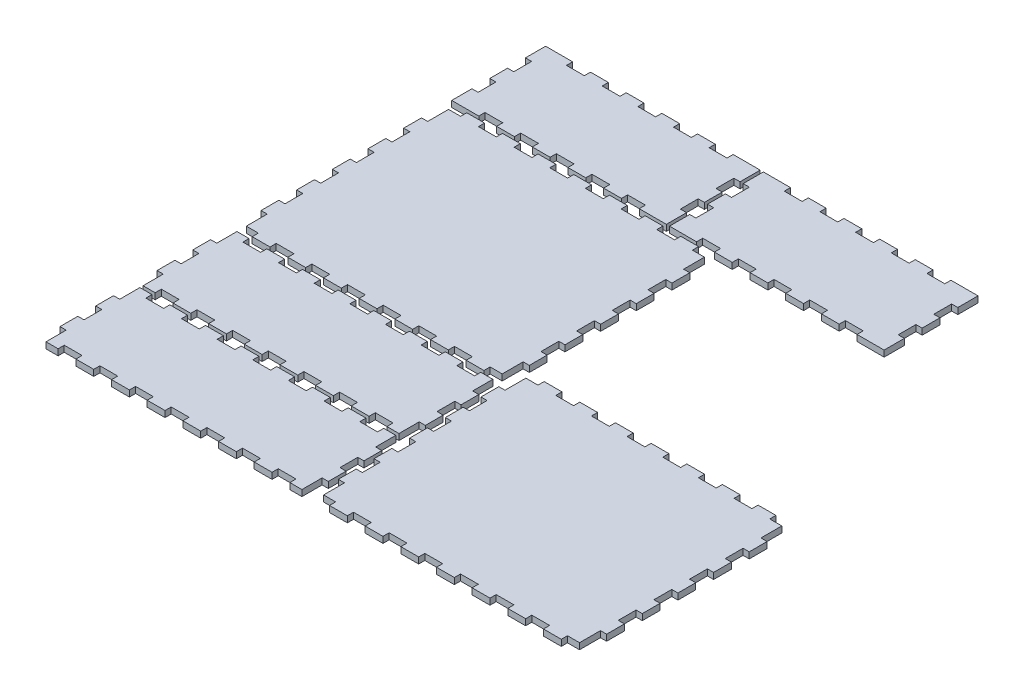
SolidWorks part; units mm, degrees
ref_plane "Front Plane" through (0, 0, 0) normal (0, 0, 1) x (1, 0, 0)
ref_plane "Top Plane" through (0, 0, 0) normal (0, 1, 0) x (1, 0, 0)
ref_plane "Right Plane" through (0, 0, 0) normal (1, 0, 0) x (0, 0, -1)
sketch "Sketch5" plane through (0, 0, 0) normal (0, 1, 0) x (1, 0, 0)
  line L0 (251.1552, 91.8972) -> (239.7252, 91.8972)
  line L1 (239.7252, 91.8972) -> (239.7252, 86.0552)
  line L2 (239.7252, 86.0552) -> (222.8596, 86.0552)
  line L3 (222.8596, 86.0552) -> (222.8596, 91.8972)
  line L4 (222.8596, 91.8972) -> (205.9686, 91.8972)
  line L5 (205.9686, 91.8972) -> (205.9686, 86.0552)
  line L6 (205.9686, 86.0552) -> (189.0776, 86.0552)
  line L7 (189.0776, 86.0552) -> (189.0776, 91.8972)
  line L8 (189.0776, 91.8972) -> (172.212, 91.8972)
  line L9 (172.212, 91.8972) -> (172.212, 86.0552)
  line L10 (172.212, 86.0552) -> (155.321, 86.0552)
  line L11 (155.321, 86.0552) -> (155.321, 91.8972)
  line L12 (155.321, 91.8972) -> (138.43, 91.8972)
  line L13 (138.43, 91.8972) -> (138.43, 86.0552)
  line L14 (138.43, 86.0552) -> (121.5644, 86.0552)
  line L15 (121.5644, 86.0552) -> (121.5644, 91.8972)
  line L16 (121.5644, 91.8972) -> (104.6734, 91.8972)
  line L17 (104.6734, 91.8972) -> (104.6734, 86.0552)
  line L18 (104.6734, 86.0552) -> (87.8078, 86.0552)
  line L19 (87.8078, 86.0552) -> (87.8078, 91.8972)
  line L20 (87.8078, 91.8972) -> (70.9168, 91.8972)
  line L21 (70.9168, 91.8972) -> (70.9168, 86.0552)
  line L22 (70.9168, 86.0552) -> (54.0258, 86.0552)
  line L23 (54.0258, 86.0552) -> (54.0258, 91.8972)
  line L24 (54.0258, 91.8972) -> (37.1602, 91.8972)
  line L25 (37.1602, 91.8972) -> (37.1602, 86.0552)
  line L26 (37.1602, 86.0552) -> (20.2692, 86.0552)
  line L27 (20.2692, 86.0552) -> (20.2692, 91.8972)
  line L28 (20.2692, 91.8972) -> (8.8392, 91.8972)
  line L29 (8.8392, 91.8972) -> (8.8392, 86.0552)
  line L30 (8.8392, 86.0552) -> (8.8392, 72.771)
  line L31 (8.8392, 72.771) -> (2.9972, 72.771)
  line L32 (2.9972, 72.771) -> (2.9972, 55.88)
  line L33 (2.9972, 55.88) -> (8.8392, 55.88)
  line L34 (8.8392, 55.88) -> (8.8392, 39.0144)
  line L35 (8.8392, 39.0144) -> (2.9972, 39.0144)
  line L36 (2.9972, 39.0144) -> (2.9972, 22.1234)
  line L37 (2.9972, 22.1234) -> (8.8392, 22.1234)
  line L38 (8.8392, 22.1234) -> (8.8392, 8.8392)
  line L39 (8.8392, 8.8392) -> (8.8392, 2.9972)
  line L40 (8.8392, 2.9972) -> (20.2692, 2.9972)
  line L41 (20.2692, 2.9972) -> (20.2692, 8.8392)
  line L42 (20.2692, 8.8392) -> (37.1602, 8.8392)
  line L43 (37.1602, 8.8392) -> (37.1602, 2.9972)
  line L44 (37.1602, 2.9972) -> (54.0258, 2.9972)
  line L45 (54.0258, 2.9972) -> (54.0258, 8.8392)
  line L46 (54.0258, 8.8392) -> (70.9168, 8.8392)
  line L47 (70.9168, 8.8392) -> (70.9168, 2.9972)
  line L48 (70.9168, 2.9972) -> (87.8078, 2.9972)
  line L49 (87.8078, 2.9972) -> (87.8078, 8.8392)
  line L50 (87.8078, 8.8392) -> (104.6734, 8.8392)
  line L51 (104.6734, 8.8392) -> (104.6734, 2.9972)
  line L52 (104.6734, 2.9972) -> (121.5644, 2.9972)
  line L53 (121.5644, 2.9972) -> (121.5644, 8.8392)
  line L54 (121.5644, 8.8392) -> (138.43, 8.8392)
  line L55 (138.43, 8.8392) -> (138.43, 2.9972)
  line L56 (138.43, 2.9972) -> (155.321, 2.9972)
  line L57 (155.321, 2.9972) -> (155.321, 8.8392)
  line L58 (155.321, 8.8392) -> (172.212, 8.8392)
  line L59 (172.212, 8.8392) -> (172.212, 2.9972)
  line L60 (172.212, 2.9972) -> (189.0776, 2.9972)
  line L61 (189.0776, 2.9972) -> (189.0776, 8.8392)
  line L62 (189.0776, 8.8392) -> (205.9686, 8.8392)
  line L63 (205.9686, 8.8392) -> (205.9686, 2.9972)
  line L64 (205.9686, 2.9972) -> (222.8596, 2.9972)
  line L65 (222.8596, 2.9972) -> (222.8596, 8.8392)
  line L66 (222.8596, 8.8392) -> (239.7252, 8.8392)
  line L67 (239.7252, 8.8392) -> (239.7252, 2.9972)
  line L68 (239.7252, 2.9972) -> (251.1552, 2.9972)
  line L69 (251.1552, 2.9972) -> (251.1552, 8.8392)
  line L70 (251.1552, 8.8392) -> (251.1552, 22.1234)
  line L71 (251.1552, 22.1234) -> (256.9972, 22.1234)
  line L72 (256.9972, 22.1234) -> (256.9972, 39.0144)
  line L73 (256.9972, 39.0144) -> (251.1552, 39.0144)
  line L74 (251.1552, 39.0144) -> (251.1552, 55.88)
  line L75 (251.1552, 55.88) -> (256.9972, 55.88)
  line L76 (256.9972, 55.88) -> (256.9972, 72.771)
  line L77 (256.9972, 72.771) -> (251.1552, 72.771)
  line L78 (251.1552, 72.771) -> (251.1552, 86.0552)
  line L79 (251.1552, 86.0552) -> (251.1552, 91.8972)
  line L80 (117.6782, 43.688) -> (116.7384, 43.688)
  line L81 (116.7384, 43.688) -> (116.7384, 51.2064)
  line L82 (116.7384, 51.2064) -> (121.3358, 51.2064)
  line L83 (121.3358, 51.2064) -> (121.3358, 50.419)
  line L84 (121.3358, 50.419) -> (117.6782, 50.419)
  line L85 (117.6782, 50.419) -> (117.6782, 47.9044)
  line L86 (117.6782, 47.9044) -> (121.0818, 47.9044)
  line L87 (121.0818, 47.9044) -> (121.0818, 47.0916)
  line L88 (121.0818, 47.0916) -> (117.6782, 47.0916)
  line L89 (117.6782, 47.0916) -> (117.6782, 43.688)
  line L90 (123.9774, 43.688) -> (123.0376, 43.688)
  line L91 (123.0376, 43.688) -> (123.0376, 49.4284)
  line L92 (123.0376, 49.4284) -> (123.9774, 49.4284)
  line L93 (123.9774, 49.4284) -> (123.9774, 43.688)
  line L94 (123.9774, 46.2788) -> (123.6726, 46.2788)
  line L95 (123.6726, 46.2788) -> (123.6726, 46.482)
  line L96 (123.6726, 46.482) -> (123.698, 46.6852)
  line L97 (123.698, 46.6852) -> (123.698, 46.8884)
  line L98 (123.698, 46.8884) -> (123.7234, 47.0916)
  line L99 (123.7234, 47.0916) -> (123.7234, 47.2694)
  line L100 (123.7234, 47.2694) -> (123.7488, 47.4472)
  line L101 (123.7488, 47.4472) -> (123.7742, 47.625)
  line L102 (123.7742, 47.625) -> (123.825, 47.7774)
  line L103 (123.825, 47.7774) -> (123.8504, 47.9298)
  line L104 (123.8504, 47.9298) -> (123.9012, 48.0822)
  line L105 (123.9012, 48.0822) -> (123.9266, 48.2346)
  line L106 (123.9266, 48.2346) -> (123.9774, 48.3616)
  line L107 (123.9774, 48.3616) -> (124.0282, 48.4886)
  line L108 (124.0282, 48.4886) -> (124.079, 48.6156)
  line L109 (124.079, 48.6156) -> (124.1552, 48.7172)
  line L110 (124.1552, 48.7172) -> (124.206, 48.8188)
  line L111 (124.206, 48.8188) -> (124.2822, 48.9204)
  line L112 (124.2822, 48.9204) -> (124.3584, 49.022)
  line L113 (124.3584, 49.022) -> (124.4346, 49.0982)
  line L114 (124.4346, 49.0982) -> (124.5108, 49.1744)
  line L115 (124.5108, 49.1744) -> (124.587, 49.2252)
  line L116 (124.587, 49.2252) -> (124.6632, 49.3014)
  line L117 (124.6632, 49.3014) -> (124.7648, 49.3522)
  line L118 (124.7648, 49.3522) -> (124.8664, 49.403)
  line L119 (124.8664, 49.403) -> (124.9426, 49.4284)
  line L120 (124.9426, 49.4284) -> (125.0442, 49.4792)
  line L121 (125.0442, 49.4792) -> (125.1458, 49.5046)
  line L122 (125.1458, 49.5046) -> (125.2728, 49.5046)
  line L123 (125.2728, 49.5046) -> (125.3744, 49.53)
  line L124 (125.3744, 49.53) -> (125.5014, 49.53)
  line L125 (125.5014, 49.53) -> (125.5268, 49.53)
  line L126 (125.5268, 49.53) -> (125.5776, 49.53)
  line L127 (125.5776, 49.53) -> (125.603, 49.53)
  line L128 (125.603, 49.53) -> (125.6284, 49.53)
  line L129 (125.6284, 49.53) -> (125.6792, 49.53)
  line L130 (125.6792, 49.53) -> (125.7046, 49.5046)
  line L131 (125.7046, 49.5046) -> (125.7554, 49.5046)
  line L132 (125.7554, 49.5046) -> (125.7808, 49.5046)
  line L133 (125.7808, 49.5046) -> (125.8062, 49.5046)
  line L134 (125.8062, 49.5046) -> (125.8316, 49.5046)
  line L135 (125.8316, 49.5046) -> (125.8824, 49.5046)
  line L136 (125.8824, 49.5046) -> (125.9078, 49.4792)
  line L137 (125.9078, 49.4792) -> (125.9332, 49.4792)
  line L138 (125.9332, 49.4792) -> (125.9586, 49.4792)
  line L139 (125.9586, 49.4792) -> (126.0094, 49.4538)
  line L140 (126.0094, 49.4538) -> (126.0348, 49.4538)
  line L141 (126.0348, 49.4538) -> (126.0602, 49.4538)
  line L142 (126.0602, 49.4538) -> (126.111, 49.4284)
  line L143 (126.111, 49.4284) -> (126.1364, 49.4284)
  line L144 (126.1364, 49.4284) -> (126.1618, 49.4284)
  line L145 (126.1618, 49.4284) -> (126.111, 48.4886)
  line L146 (126.111, 48.4886) -> (126.0602, 48.514)
  line L147 (126.0602, 48.514) -> (126.0348, 48.514)
  line L148 (126.0348, 48.514) -> (126.0094, 48.514)
  line L149 (126.0094, 48.514) -> (125.9586, 48.5394)
  line L150 (125.9586, 48.5394) -> (125.9332, 48.5394)
  line L151 (125.9332, 48.5394) -> (125.8824, 48.5648)
  line L152 (125.8824, 48.5648) -> (125.857, 48.5648)
  line L153 (125.857, 48.5648) -> (125.8062, 48.5648)
  line L154 (125.8062, 48.5648) -> (125.7808, 48.5902)
  line L155 (125.7808, 48.5902) -> (125.73, 48.5902)
  line L156 (125.73, 48.5902) -> (125.7046, 48.5902)
  line L157 (125.7046, 48.5902) -> (125.6538, 48.5902)
  line L158 (125.6538, 48.5902) -> (125.6284, 48.6156)
  line L159 (125.6284, 48.6156) -> (125.5776, 48.6156)
  line L160 (125.5776, 48.6156) -> (125.5522, 48.6156)
  line L161 (125.5522, 48.6156) -> (125.5268, 48.6156)
  line L162 (125.5268, 48.6156) -> (125.476, 48.6156)
  line L163 (125.476, 48.6156) -> (125.4506, 48.6156)
  line L164 (125.4506, 48.6156) -> (125.4252, 48.6156)
  line L165 (125.4252, 48.6156) -> (125.3744, 48.6156)
  line L166 (125.3744, 48.6156) -> (125.2728, 48.6156)
  line L167 (125.2728, 48.6156) -> (125.1966, 48.6156)
  line L168 (125.1966, 48.6156) -> (125.095, 48.5902)
  line L169 (125.095, 48.5902) -> (125.0188, 48.5902)
  line L170 (125.0188, 48.5902) -> (124.9172, 48.5648)
  line L171 (124.9172, 48.5648) -> (124.841, 48.514)
  line L172 (124.841, 48.514) -> (124.7648, 48.4886)
  line L173 (124.7648, 48.4886) -> (124.6886, 48.4378)
  line L174 (124.6886, 48.4378) -> (124.6378, 48.387)
  line L175 (124.6378, 48.387) -> (124.5616, 48.3362)
  line L176 (124.5616, 48.3362) -> (124.5108, 48.2854)
  line L177 (124.5108, 48.2854) -> (124.4346, 48.2092)
  line L178 (124.4346, 48.2092) -> (124.3838, 48.133)
  line L179 (124.3838, 48.133) -> (124.333, 48.0568)
  line L180 (124.333, 48.0568) -> (124.2822, 47.9806)
  line L181 (124.2822, 47.9806) -> (124.2568, 47.9044)
  line L182 (124.2568, 47.9044) -> (124.206, 47.8028)
  line L183 (124.206, 47.8028) -> (124.1806, 47.7266)
  line L184 (124.1806, 47.7266) -> (124.1298, 47.625)
  line L185 (124.1298, 47.625) -> (124.1044, 47.5234)
  line L186 (124.1044, 47.5234) -> (124.079, 47.3964)
  line L187 (124.079, 47.3964) -> (124.0536, 47.2948)
  line L188 (124.0536, 47.2948) -> (124.0282, 47.1932)
  line L189 (124.0282, 47.1932) -> (124.0282, 47.0662)
  line L190 (124.0282, 47.0662) -> (124.0028, 46.9392)
  line L191 (124.0028, 46.9392) -> (123.9774, 46.8122)
  line L192 (123.9774, 46.8122) -> (123.9774, 46.6852)
  line L193 (123.9774, 46.6852) -> (123.9774, 46.5582)
  line L194 (123.9774, 46.5582) -> (123.9774, 46.4058)
  line L195 (123.9774, 46.4058) -> (123.9774, 46.2788)
  line L196 (129.4384, 43.5356) -> (129.286, 43.5356)
  line L197 (129.286, 43.5356) -> (129.1336, 43.561)
  line L198 (129.1336, 43.561) -> (129.0066, 43.561)
  line L199 (129.0066, 43.561) -> (128.8542, 43.5864)
  line L200 (128.8542, 43.5864) -> (128.7018, 43.6118)
  line L201 (128.7018, 43.6118) -> (128.5748, 43.6626)
  line L202 (128.5748, 43.6626) -> (128.4478, 43.7134)
  line L203 (128.4478, 43.7134) -> (128.3208, 43.7642)
  line L204 (128.3208, 43.7642) -> (128.1938, 43.815)
  line L205 (128.1938, 43.815) -> (128.0668, 43.8912)
  line L206 (128.0668, 43.8912) -> (127.9398, 43.942)
  line L207 (127.9398, 43.942) -> (127.8382, 44.0182)
  line L208 (127.8382, 44.0182) -> (127.7366, 44.1198)
  line L209 (127.7366, 44.1198) -> (127.635, 44.196)
  line L210 (127.635, 44.196) -> (127.5334, 44.2976)
  line L211 (127.5334, 44.2976) -> (127.4318, 44.3992)
  line L212 (127.4318, 44.3992) -> (127.3556, 44.5262)
  line L213 (127.3556, 44.5262) -> (127.254, 44.6278)
  line L214 (127.254, 44.6278) -> (127.1778, 44.7548)
  line L215 (127.1778, 44.7548) -> (127.127, 44.8818)
  line L216 (127.127, 44.8818) -> (127.0508, 45.0342)
  line L217 (127.0508, 45.0342) -> (127, 45.1866)
  line L218 (127, 45.1866) -> (126.9492, 45.3136)
  line L219 (126.9492, 45.3136) -> (126.8984, 45.4914)
  line L220 (126.8984, 45.4914) -> (126.8476, 45.6438)
  line L221 (126.8476, 45.6438) -> (126.8222, 45.8216)
  line L222 (126.8222, 45.8216) -> (126.7968, 45.9994)
  line L223 (126.7968, 45.9994) -> (126.7714, 46.1772)
  line L224 (126.7714, 46.1772) -> (126.7714, 46.355)
  line L225 (126.7714, 46.355) -> (126.7714, 46.5582)
  line L226 (126.7714, 46.5582) -> (126.7714, 46.736)
  line L227 (126.7714, 46.736) -> (126.7714, 46.9392)
  line L228 (126.7714, 46.9392) -> (126.7968, 47.117)
  line L229 (126.7968, 47.117) -> (126.8222, 47.2948)
  line L230 (126.8222, 47.2948) -> (126.8476, 47.4726)
  line L231 (126.8476, 47.4726) -> (126.8984, 47.625)
  line L232 (126.8984, 47.625) -> (126.9492, 47.7774)
  line L233 (126.9492, 47.7774) -> (127, 47.9298)
  line L234 (127, 47.9298) -> (127.0508, 48.0822)
  line L235 (127.0508, 48.0822) -> (127.127, 48.2092)
  line L236 (127.127, 48.2092) -> (127.1778, 48.3362)
  line L237 (127.1778, 48.3362) -> (127.254, 48.4632)
  line L238 (127.254, 48.4632) -> (127.3556, 48.5902)
  line L239 (127.3556, 48.5902) -> (127.4318, 48.6918)
  line L240 (127.4318, 48.6918) -> (127.5334, 48.7934)
  line L241 (127.5334, 48.7934) -> (127.635, 48.895)
  line L242 (127.635, 48.895) -> (127.7366, 48.9966)
  line L243 (127.7366, 48.9966) -> (127.8382, 49.0728)
  line L244 (127.8382, 49.0728) -> (127.9398, 49.149)
  line L245 (127.9398, 49.149) -> (128.0668, 49.2252)
  line L246 (128.0668, 49.2252) -> (128.1938, 49.276)
  line L247 (128.1938, 49.276) -> (128.3208, 49.3522)
  line L248 (128.3208, 49.3522) -> (128.4478, 49.403)
  line L249 (128.4478, 49.403) -> (128.5748, 49.4284)
  line L250 (128.5748, 49.4284) -> (128.7018, 49.4792)
  line L251 (128.7018, 49.4792) -> (128.8542, 49.5046)
  line L252 (128.8542, 49.5046) -> (129.0066, 49.53)
  line L253 (129.0066, 49.53) -> (129.1336, 49.5554)
  line L254 (129.1336, 49.5554) -> (129.286, 49.5554)
  line L255 (129.286, 49.5554) -> (129.4384, 49.5554)
  line L256 (129.4384, 49.5554) -> (129.5908, 49.5554)
  line L257 (129.5908, 49.5554) -> (129.7432, 49.5554)
  line L258 (129.7432, 49.5554) -> (129.8956, 49.53)
  line L259 (129.8956, 49.53) -> (130.0226, 49.5046)
  line L260 (130.0226, 49.5046) -> (130.175, 49.4792)
  line L261 (130.175, 49.4792) -> (130.302, 49.4284)
  line L262 (130.302, 49.4284) -> (130.429, 49.403)
  line L263 (130.429, 49.403) -> (130.556, 49.3522)
  line L264 (130.556, 49.3522) -> (130.683, 49.276)
  line L265 (130.683, 49.276) -> (130.81, 49.2252)
  line L266 (130.81, 49.2252) -> (130.937, 49.149)
  line L267 (130.937, 49.149) -> (131.0386, 49.0728)
  line L268 (131.0386, 49.0728) -> (131.1656, 48.9966)
  line L269 (131.1656, 48.9966) -> (131.2672, 48.895)
  line L270 (131.2672, 48.895) -> (131.3434, 48.7934)
  line L271 (131.3434, 48.7934) -> (131.445, 48.6918)
  line L272 (131.445, 48.6918) -> (131.5212, 48.5902)
  line L273 (131.5212, 48.5902) -> (131.6228, 48.4632)
  line L274 (131.6228, 48.4632) -> (131.699, 48.3362)
  line L275 (131.699, 48.3362) -> (131.7752, 48.2092)
  line L276 (131.7752, 48.2092) -> (131.826, 48.0822)
  line L277 (131.826, 48.0822) -> (131.8768, 47.9298)
  line L278 (131.8768, 47.9298) -> (131.9276, 47.7774)
  line L279 (131.9276, 47.7774) -> (131.9784, 47.625)
  line L280 (131.9784, 47.625) -> (132.0292, 47.4726)
  line L281 (132.0292, 47.4726) -> (132.0546, 47.2948)
  line L282 (132.0546, 47.2948) -> (132.08, 47.117)
  line L283 (132.08, 47.117) -> (132.1054, 46.9392)
  line L284 (132.1054, 46.9392) -> (132.1054, 46.736)
  line L285 (132.1054, 46.736) -> (132.1054, 46.5582)
  line L286 (132.1054, 46.5582) -> (132.1054, 46.355)
  line L287 (132.1054, 46.355) -> (132.1054, 46.1772)
  line L288 (132.1054, 46.1772) -> (132.08, 45.9994)
  line L289 (132.08, 45.9994) -> (132.0546, 45.8216)
  line L290 (132.0546, 45.8216) -> (132.0292, 45.6438)
  line L291 (132.0292, 45.6438) -> (131.9784, 45.4914)
  line L292 (131.9784, 45.4914) -> (131.9276, 45.3136)
  line L293 (131.9276, 45.3136) -> (131.8768, 45.1866)
  line L294 (131.8768, 45.1866) -> (131.826, 45.0342)
  line L295 (131.826, 45.0342) -> (131.7752, 44.8818)
  line L296 (131.7752, 44.8818) -> (131.699, 44.7548)
  line L297 (131.699, 44.7548) -> (131.6228, 44.6278)
  line L298 (131.6228, 44.6278) -> (131.5212, 44.5262)
  line L299 (131.5212, 44.5262) -> (131.445, 44.3992)
  line L300 (131.445, 44.3992) -> (131.3434, 44.2976)
  line L301 (131.3434, 44.2976) -> (131.2672, 44.196)
  line L302 (131.2672, 44.196) -> (131.1656, 44.1198)
  line L303 (131.1656, 44.1198) -> (131.0386, 44.0182)
  line L304 (131.0386, 44.0182) -> (130.937, 43.942)
  line L305 (130.937, 43.942) -> (130.81, 43.8912)
  line L306 (130.81, 43.8912) -> (130.683, 43.815)
  line L307 (130.683, 43.815) -> (130.556, 43.7642)
  line L308 (130.556, 43.7642) -> (130.429, 43.7134)
  line L309 (130.429, 43.7134) -> (130.302, 43.6626)
  line L310 (130.302, 43.6626) -> (130.175, 43.6118)
  line L311 (130.175, 43.6118) -> (130.0226, 43.5864)
  line L312 (130.0226, 43.5864) -> (129.8956, 43.561)
  line L313 (129.8956, 43.561) -> (129.7432, 43.561)
  line L314 (129.7432, 43.561) -> (129.5908, 43.5356)
  line L315 (129.5908, 43.5356) -> (129.4384, 43.5356)
  line L316 (129.413, 44.3484) -> (129.54, 44.3484)
  line L317 (129.54, 44.3484) -> (129.6416, 44.3738)
  line L318 (129.6416, 44.3738) -> (129.7432, 44.3738)
  line L319 (129.7432, 44.3738) -> (129.8448, 44.3992)
  line L320 (129.8448, 44.3992) -> (129.9464, 44.4246)
  line L321 (129.9464, 44.4246) -> (130.0226, 44.45)
  line L322 (130.0226, 44.45) -> (130.1242, 44.4754)
  line L323 (130.1242, 44.4754) -> (130.2004, 44.5262)
  line L324 (130.2004, 44.5262) -> (130.302, 44.577)
  line L325 (130.302, 44.577) -> (130.3782, 44.6278)
  line L326 (130.3782, 44.6278) -> (130.4544, 44.6786)
  line L327 (130.4544, 44.6786) -> (130.5052, 44.7294)
  line L328 (130.5052, 44.7294) -> (130.5814, 44.8056)
  line L329 (130.5814, 44.8056) -> (130.6576, 44.8818)
  line L330 (130.6576, 44.8818) -> (130.7084, 44.9326)
  line L331 (130.7084, 44.9326) -> (130.7592, 45.0342)
  line L332 (130.7592, 45.0342) -> (130.81, 45.1104)
  line L333 (130.81, 45.1104) -> (130.8608, 45.1866)
  line L334 (130.8608, 45.1866) -> (130.9116, 45.2882)
  line L335 (130.9116, 45.2882) -> (130.9624, 45.3898)
  line L336 (130.9624, 45.3898) -> (130.9878, 45.4914)
  line L337 (130.9878, 45.4914) -> (131.0386, 45.593)
  line L338 (131.0386, 45.593) -> (131.064, 45.6946)
  line L339 (131.064, 45.6946) -> (131.0894, 45.7962)
  line L340 (131.0894, 45.7962) -> (131.1148, 45.9232)
  line L341 (131.1148, 45.9232) -> (131.1402, 46.0502)
  line L342 (131.1402, 46.0502) -> (131.1402, 46.1518)
  line L343 (131.1402, 46.1518) -> (131.1656, 46.2788)
  line L344 (131.1656, 46.2788) -> (131.1656, 46.4058)
  line L345 (131.1656, 46.4058) -> (131.1656, 46.5582)
  line L346 (131.1656, 46.5582) -> (131.1656, 46.7614)
  line L347 (131.1656, 46.7614) -> (131.1402, 46.9392)
  line L348 (131.1402, 46.9392) -> (131.1148, 47.117)
  line L349 (131.1148, 47.117) -> (131.0894, 47.2948)
  line L350 (131.0894, 47.2948) -> (131.064, 47.4726)
  line L351 (131.064, 47.4726) -> (131.0132, 47.625)
  line L352 (131.0132, 47.625) -> (130.9624, 47.7774)
  line L353 (130.9624, 47.7774) -> (130.8862, 47.9044)
  line L354 (130.8862, 47.9044) -> (130.81, 48.0568)
  line L355 (130.81, 48.0568) -> (130.7338, 48.1584)
  line L356 (130.7338, 48.1584) -> (130.6576, 48.2854)
  line L357 (130.6576, 48.2854) -> (130.556, 48.387)
  line L358 (130.556, 48.387) -> (130.4544, 48.4632)
  line L359 (130.4544, 48.4632) -> (130.3274, 48.5394)
  line L360 (130.3274, 48.5394) -> (130.2004, 48.6156)
  line L361 (130.2004, 48.6156) -> (130.0734, 48.6664)
  line L362 (130.0734, 48.6664) -> (129.9464, 48.7172)
  line L363 (129.9464, 48.7172) -> (129.794, 48.7426)
  line L364 (129.794, 48.7426) -> (129.6416, 48.7426)
  line L365 (129.6416, 48.7426) -> (129.4638, 48.768)
  line L366 (129.4638, 48.768) -> (129.3622, 48.768)
  line L367 (129.3622, 48.768) -> (129.2606, 48.7426)
  line L368 (129.2606, 48.7426) -> (129.159, 48.7426)
  line L369 (129.159, 48.7426) -> (129.0574, 48.7172)
  line L370 (129.0574, 48.7172) -> (128.9558, 48.6918)
  line L371 (128.9558, 48.6918) -> (128.8542, 48.6664)
  line L372 (128.8542, 48.6664) -> (128.778, 48.6156)
  line L373 (128.778, 48.6156) -> (128.6764, 48.5902)
  line L374 (128.6764, 48.5902) -> (128.6002, 48.5394)
  line L375 (128.6002, 48.5394) -> (128.524, 48.4886)
  line L376 (128.524, 48.4886) -> (128.4478, 48.4378)
  line L377 (128.4478, 48.4378) -> (128.3716, 48.387)
  line L378 (128.3716, 48.387) -> (128.2954, 48.3108)
  line L379 (128.2954, 48.3108) -> (128.2446, 48.2346)
  line L380 (128.2446, 48.2346) -> (128.1684, 48.1584)
  line L381 (128.1684, 48.1584) -> (128.1176, 48.0822)
  line L382 (128.1176, 48.0822) -> (128.0668, 48.006)
  line L383 (128.0668, 48.006) -> (128.016, 47.9298)
  line L384 (128.016, 47.9298) -> (127.9652, 47.8282)
  line L385 (127.9652, 47.8282) -> (127.9398, 47.7266)
  line L386 (127.9398, 47.7266) -> (127.889, 47.625)
  line L387 (127.889, 47.625) -> (127.8636, 47.5234)
  line L388 (127.8636, 47.5234) -> (127.8382, 47.4218)
  line L389 (127.8382, 47.4218) -> (127.8128, 47.2948)
  line L390 (127.8128, 47.2948) -> (127.7874, 47.1932)
  line L391 (127.7874, 47.1932) -> (127.762, 47.0662)
  line L392 (127.762, 47.0662) -> (127.7366, 46.9392)
  line L393 (127.7366, 46.9392) -> (127.7366, 46.8122)
  line L394 (127.7366, 46.8122) -> (127.7366, 46.6852)
  line L395 (127.7366, 46.6852) -> (127.7366, 46.5582)
  line L396 (127.7366, 46.5582) -> (127.7366, 46.355)
  line L397 (127.7366, 46.355) -> (127.7366, 46.1518)
  line L398 (127.7366, 46.1518) -> (127.762, 45.974)
  line L399 (127.762, 45.974) -> (127.7874, 45.7962)
  line L400 (127.7874, 45.7962) -> (127.8382, 45.6438)
  line L401 (127.8382, 45.6438) -> (127.889, 45.4914)
  line L402 (127.889, 45.4914) -> (127.9398, 45.339)
  line L403 (127.9398, 45.339) -> (128.016, 45.1866)
  line L404 (128.016, 45.1866) -> (128.0668, 45.0596)
  line L405 (128.0668, 45.0596) -> (128.1684, 44.9326)
  line L406 (128.1684, 44.9326) -> (128.2446, 44.831)
  line L407 (128.2446, 44.831) -> (128.3462, 44.7294)
  line L408 (128.3462, 44.7294) -> (128.4478, 44.6532)
  line L409 (128.4478, 44.6532) -> (128.5748, 44.577)
  line L410 (128.5748, 44.577) -> (128.6764, 44.5008)
  line L411 (128.6764, 44.5008) -> (128.8288, 44.45)
  line L412 (128.8288, 44.45) -> (128.9558, 44.3992)
  line L413 (128.9558, 44.3992) -> (129.1082, 44.3738)
  line L414 (129.1082, 44.3738) -> (129.2606, 44.3484)
  line L415 (129.2606, 44.3484) -> (129.413, 44.3484)
  line L416 (138.938, 43.688) -> (137.9982, 43.688)
  line L417 (137.9982, 43.688) -> (137.9982, 47.0662)
  line L418 (137.9982, 47.0662) -> (137.9982, 47.2186)
  line L419 (137.9982, 47.2186) -> (137.9982, 47.371)
  line L420 (137.9982, 47.371) -> (137.9728, 47.5234)
  line L421 (137.9728, 47.5234) -> (137.9474, 47.6504)
  line L422 (137.9474, 47.6504) -> (137.8966, 47.7774)
  line L423 (137.8966, 47.7774) -> (137.8712, 47.9044)
  line L424 (137.8712, 47.9044) -> (137.8204, 48.006)
  line L425 (137.8204, 48.006) -> (137.7442, 48.1076)
  line L426 (137.7442, 48.1076) -> (137.6934, 48.2092)
  line L427 (137.6934, 48.2092) -> (137.6172, 48.3108)
  line L428 (137.6172, 48.3108) -> (137.541, 48.387)
  line L429 (137.541, 48.387) -> (137.4394, 48.4632)
  line L430 (137.4394, 48.4632) -> (137.3632, 48.514)
  line L431 (137.3632, 48.514) -> (137.2616, 48.5902)
  line L432 (137.2616, 48.5902) -> (137.16, 48.6156)
  line L433 (137.16, 48.6156) -> (137.033, 48.6664)
  line L434 (137.033, 48.6664) -> (136.9314, 48.6918)
  line L435 (136.9314, 48.6918) -> (136.8044, 48.7172)
  line L436 (136.8044, 48.7172) -> (136.6774, 48.7426)
  line L437 (136.6774, 48.7426) -> (136.5504, 48.7426)
  line L438 (136.5504, 48.7426) -> (136.4488, 48.7426)
  line L439 (136.4488, 48.7426) -> (136.3472, 48.7172)
  line L440 (136.3472, 48.7172) -> (136.2456, 48.7172)
  line L441 (136.2456, 48.7172) -> (136.144, 48.6918)
  line L442 (136.144, 48.6918) -> (136.0678, 48.6664)
  line L443 (136.0678, 48.6664) -> (135.9662, 48.641)
  line L444 (135.9662, 48.641) -> (135.89, 48.5902)
  line L445 (135.89, 48.5902) -> (135.8138, 48.5648)
  line L446 (135.8138, 48.5648) -> (135.7376, 48.514)
  line L447 (135.7376, 48.514) -> (135.6614, 48.4632)
  line L448 (135.6614, 48.4632) -> (135.5852, 48.387)
  line L449 (135.5852, 48.387) -> (135.509, 48.3362)
  line L450 (135.509, 48.3362) -> (135.4328, 48.26)
  line L451 (135.4328, 48.26) -> (135.382, 48.1838)
  line L452 (135.382, 48.1838) -> (135.3058, 48.1076)
  line L453 (135.3058, 48.1076) -> (135.255, 48.0314)
  line L454 (135.255, 48.0314) -> (135.2042, 47.9298)
  line L455 (135.2042, 47.9298) -> (135.1534, 47.8536)
  line L456 (135.1534, 47.8536) -> (135.1026, 47.752)
  line L457 (135.1026, 47.752) -> (135.0772, 47.6504)
  line L458 (135.0772, 47.6504) -> (135.0264, 47.5488)
  line L459 (135.0264, 47.5488) -> (135.001, 47.4218)
  line L460 (135.001, 47.4218) -> (134.9756, 47.3202)
  line L461 (134.9756, 47.3202) -> (134.9248, 47.1932)
  line L462 (134.9248, 47.1932) -> (134.9248, 47.0662)
  line L463 (134.9248, 47.0662) -> (134.8994, 46.9392)
  line L464 (134.8994, 46.9392) -> (134.874, 46.8122)
  line L465 (134.874, 46.8122) -> (134.874, 46.6852)
  line L466 (134.874, 46.6852) -> (134.874, 46.5328)
  line L467 (134.874, 46.5328) -> (134.874, 46.4058)
  line L468 (134.874, 46.4058) -> (134.493, 46.4058)
  line L469 (134.493, 46.4058) -> (134.493, 46.5836)
  line L470 (134.493, 46.5836) -> (134.5184, 46.7868)
  line L471 (134.5184, 46.7868) -> (134.5184, 46.9646)
  line L472 (134.5184, 46.9646) -> (134.5438, 47.1424)
  line L473 (134.5438, 47.1424) -> (134.5692, 47.3202)
  line L474 (134.5692, 47.3202) -> (134.5946, 47.498)
  line L475 (134.5946, 47.498) -> (134.62, 47.6504)
  line L476 (134.62, 47.6504) -> (134.6708, 47.8028)
  line L477 (134.6708, 47.8028) -> (134.7216, 47.9552)
  line L478 (134.7216, 47.9552) -> (134.7724, 48.1076)
  line L479 (134.7724, 48.1076) -> (134.8232, 48.2346)
  line L480 (134.8232, 48.2346) -> (134.874, 48.3616)
  line L481 (134.874, 48.3616) -> (134.9502, 48.4886)
  line L482 (134.9502, 48.4886) -> (135.0264, 48.6156)
  line L483 (135.0264, 48.6156) -> (135.1026, 48.7172)
  line L484 (135.1026, 48.7172) -> (135.1788, 48.8442)
  line L485 (135.1788, 48.8442) -> (135.255, 48.9204)
  line L486 (135.255, 48.9204) -> (135.3566, 49.022)
  line L487 (135.3566, 49.022) -> (135.4328, 49.0982)
  line L488 (135.4328, 49.0982) -> (135.5344, 49.1998)
  line L489 (135.5344, 49.1998) -> (135.636, 49.2506)
  line L490 (135.636, 49.2506) -> (135.7376, 49.3268)
  line L491 (135.7376, 49.3268) -> (135.8646, 49.3776)
  line L492 (135.8646, 49.3776) -> (135.9662, 49.4284)
  line L493 (135.9662, 49.4284) -> (136.0932, 49.4792)
  line L494 (136.0932, 49.4792) -> (136.2202, 49.5046)
  line L495 (136.2202, 49.5046) -> (136.3472, 49.53)
  line L496 (136.3472, 49.53) -> (136.4996, 49.5554)
  line L497 (136.4996, 49.5554) -> (136.6266, 49.5554)
  line L498 (136.6266, 49.5554) -> (136.779, 49.5554)
  line L499 (136.779, 49.5554) -> (136.906, 49.5554)
  line L500 (136.906, 49.5554) -> (137.033, 49.5554)
  line L501 (137.033, 49.5554) -> (137.16, 49.53)
  line L502 (137.16, 49.53) -> (137.287, 49.5046)
  line L503 (137.287, 49.5046) -> (137.3886, 49.4792)
  line L504 (137.3886, 49.4792) -> (137.5156, 49.4538)
  line L505 (137.5156, 49.4538) -> (137.6172, 49.403)
  line L506 (137.6172, 49.403) -> (137.7188, 49.3776)
  line L507 (137.7188, 49.3776) -> (137.8458, 49.3268)
  line L508 (137.8458, 49.3268) -> (137.922, 49.2506)
  line L509 (137.922, 49.2506) -> (138.0236, 49.1998)
  line L510 (138.0236, 49.1998) -> (138.1252, 49.1236)
  line L511 (138.1252, 49.1236) -> (138.2014, 49.0474)
  line L512 (138.2014, 49.0474) -> (138.2776, 48.9712)
  line L513 (138.2776, 48.9712) -> (138.3538, 48.895)
  line L514 (138.3538, 48.895) -> (138.43, 48.7934)
  line L515 (138.43, 48.7934) -> (138.5062, 48.7172)
  line L516 (138.5062, 48.7172) -> (138.557, 48.6156)
  line L517 (138.557, 48.6156) -> (138.6078, 48.514)
  line L518 (138.6078, 48.514) -> (138.684, 48.387)
  line L519 (138.684, 48.387) -> (138.7094, 48.2854)
  line L520 (138.7094, 48.2854) -> (138.7602, 48.1584)
  line L521 (138.7602, 48.1584) -> (138.811, 48.0314)
  line L522 (138.811, 48.0314) -> (138.8364, 47.9044)
  line L523 (138.8364, 47.9044) -> (138.8618, 47.7774)
  line L524 (138.8618, 47.7774) -> (138.8872, 47.6504)
  line L525 (138.8872, 47.6504) -> (138.9126, 47.498)
  line L526 (138.9126, 47.498) -> (138.9126, 47.3456)
  line L527 (138.9126, 47.3456) -> (138.938, 47.2186)
  line L528 (138.938, 47.2186) -> (138.938, 47.0662)
  line L529 (138.938, 47.0662) -> (138.938, 43.688)
  line L530 (134.874, 43.688) -> (133.9342, 43.688)
  line L531 (133.9342, 43.688) -> (133.9342, 49.4284)
  line L532 (133.9342, 49.4284) -> (134.7216, 49.4284)
  line L533 (134.7216, 49.4284) -> (134.874, 48.1076)
  line L534 (134.874, 48.1076) -> (134.874, 43.688)
  line L535 (142.9258, 43.5356) -> (142.8496, 43.5356)
  line L536 (142.8496, 43.5356) -> (142.748, 43.5356)
  line L537 (142.748, 43.5356) -> (142.6718, 43.561)
  line L538 (142.6718, 43.561) -> (142.5702, 43.561)
  line L539 (142.5702, 43.561) -> (142.494, 43.5864)
  line L540 (142.494, 43.5864) -> (142.4178, 43.6118)
  line L541 (142.4178, 43.6118) -> (142.3162, 43.6372)
  line L542 (142.3162, 43.6372) -> (142.24, 43.6626)
  line L543 (142.24, 43.6626) -> (142.1638, 43.688)
  line L544 (142.1638, 43.688) -> (142.0876, 43.7134)
  line L545 (142.0876, 43.7134) -> (142.0114, 43.7642)
  line L546 (142.0114, 43.7642) -> (141.9606, 43.7896)
  line L547 (141.9606, 43.7896) -> (141.8844, 43.8404)
  line L548 (141.8844, 43.8404) -> (141.8082, 43.8912)
  line L549 (141.8082, 43.8912) -> (141.7574, 43.942)
  line L550 (141.7574, 43.942) -> (141.7066, 43.9928)
  line L551 (141.7066, 43.9928) -> (141.6558, 44.069)
  line L552 (141.6558, 44.069) -> (141.605, 44.1198)
  line L553 (141.605, 44.1198) -> (141.5542, 44.196)
  line L554 (141.5542, 44.196) -> (141.5034, 44.2468)
  line L555 (141.5034, 44.2468) -> (141.4526, 44.323)
  line L556 (141.4526, 44.323) -> (141.4272, 44.3992)
  line L557 (141.4272, 44.3992) -> (141.4018, 44.5008)
  line L558 (141.4018, 44.5008) -> (141.3764, 44.577)
  line L559 (141.3764, 44.577) -> (141.351, 44.6532)
  line L560 (141.351, 44.6532) -> (141.3256, 44.7548)
  line L561 (141.3256, 44.7548) -> (141.3002, 44.8564)
  line L562 (141.3002, 44.8564) -> (141.3002, 44.958)
  line L563 (141.3002, 44.958) -> (141.3002, 45.0596)
  line L564 (141.3002, 45.0596) -> (141.3002, 45.1612)
  line L565 (141.3002, 45.1612) -> (141.3002, 51.0032)
  line L566 (141.3002, 51.0032) -> (142.2146, 51.0032)
  line L567 (142.2146, 51.0032) -> (142.2146, 45.1866)
  line L568 (142.2146, 45.1866) -> (142.2146, 45.0088)
  line L569 (142.2146, 45.0088) -> (142.24, 44.8564)
  line L570 (142.24, 44.8564) -> (142.2908, 44.7294)
  line L571 (142.2908, 44.7294) -> (142.3416, 44.6024)
  line L572 (142.3416, 44.6024) -> (142.4178, 44.5262)
  line L573 (142.4178, 44.5262) -> (142.5194, 44.4246)
  line L574 (142.5194, 44.4246) -> (142.621, 44.3738)
  line L575 (142.621, 44.3738) -> (142.748, 44.323)
  line L576 (142.748, 44.323) -> (142.875, 44.2976)
  line L577 (142.875, 44.2976) -> (143.0528, 44.2976)
  line L578 (143.0528, 44.2976) -> (143.0782, 44.2976)
  line L579 (143.0782, 44.2976) -> (143.129, 44.2976)
  line L580 (143.129, 44.2976) -> (143.1798, 44.2976)
  line L581 (143.1798, 44.2976) -> (143.2306, 44.2976)
  line L582 (143.2306, 44.2976) -> (143.2814, 44.2976)
  line L583 (143.2814, 44.2976) -> (143.3322, 44.323)
  line L584 (143.3322, 44.323) -> (143.383, 44.323)
  line L585 (143.383, 44.323) -> (143.4338, 44.323)
  line L586 (143.4338, 44.323) -> (143.4592, 44.3484)
  line L587 (143.4592, 44.3484) -> (143.51, 44.3484)
  line L588 (143.51, 44.3484) -> (143.5608, 44.3484)
  line L589 (143.5608, 44.3484) -> (143.6116, 44.3738)
  line L590 (143.6116, 44.3738) -> (143.6624, 44.3738)
  line L591 (143.6624, 44.3738) -> (143.7132, 44.3992)
  line L592 (143.7132, 44.3992) -> (143.764, 44.4246)
  line L593 (143.764, 44.4246) -> (143.8148, 44.4246)
  line L594 (143.8148, 44.4246) -> (143.8656, 44.45)
  line L595 (143.8656, 44.45) -> (143.9164, 44.4754)
  line L596 (143.9164, 44.4754) -> (143.9926, 44.5008)
  line L597 (143.9926, 44.5008) -> (144.0434, 44.5008)
  line L598 (144.0434, 44.5008) -> (144.1704, 43.8404)
  line L599 (144.1704, 43.8404) -> (144.1196, 43.815)
  line L600 (144.1196, 43.815) -> (144.0434, 43.7896)
  line L601 (144.0434, 43.7896) -> (143.9926, 43.7642)
  line L602 (143.9926, 43.7642) -> (143.9164, 43.7388)
  line L603 (143.9164, 43.7388) -> (143.8656, 43.7134)
  line L604 (143.8656, 43.7134) -> (143.8148, 43.688)
  line L605 (143.8148, 43.688) -> (143.7386, 43.688)
  line L606 (143.7386, 43.688) -> (143.6878, 43.6626)
  line L607 (143.6878, 43.6626) -> (143.6116, 43.6372)
  line L608 (143.6116, 43.6372) -> (143.5608, 43.6118)
  line L609 (143.5608, 43.6118) -> (143.51, 43.6118)
  line L610 (143.51, 43.6118) -> (143.4338, 43.5864)
  line L611 (143.4338, 43.5864) -> (143.383, 43.5864)
  line L612 (143.383, 43.5864) -> (143.3068, 43.561)
  line L613 (143.3068, 43.561) -> (143.256, 43.561)
  line L614 (143.256, 43.561) -> (143.1798, 43.561)
  line L615 (143.1798, 43.561) -> (143.129, 43.5356)
  line L616 (143.129, 43.5356) -> (143.0528, 43.5356)
  line L617 (143.0528, 43.5356) -> (143.002, 43.5356)
  line L618 (143.002, 43.5356) -> (142.9258, 43.5356)
  line L619 (144.018, 48.768) -> (140.3604, 48.768)
  line L620 (140.3604, 48.768) -> (140.3604, 49.4284)
  line L621 (140.3604, 49.4284) -> (144.018, 49.4284)
  line L622 (144.018, 49.4284) -> (144.018, 48.768)
  line L623 (251.1552, 183.7944) -> (239.7252, 183.7944)
  line L624 (239.7252, 183.7944) -> (239.7252, 177.9524)
  line L625 (239.7252, 177.9524) -> (222.8596, 177.9524)
  line L626 (222.8596, 177.9524) -> (222.8596, 183.7944)
  line L627 (222.8596, 183.7944) -> (205.9686, 183.7944)
  line L628 (205.9686, 183.7944) -> (205.9686, 177.9524)
  line L629 (205.9686, 177.9524) -> (189.0776, 177.9524)
  line L630 (189.0776, 177.9524) -> (189.0776, 183.7944)
  line L631 (189.0776, 183.7944) -> (172.212, 183.7944)
  line L632 (172.212, 183.7944) -> (172.212, 177.9524)
  line L633 (172.212, 177.9524) -> (155.321, 177.9524)
  line L634 (155.321, 177.9524) -> (155.321, 183.7944)
  line L635 (155.321, 183.7944) -> (138.43, 183.7944)
  line L636 (138.43, 183.7944) -> (138.43, 177.9524)
  line L637 (138.43, 177.9524) -> (121.5644, 177.9524)
  line L638 (121.5644, 177.9524) -> (121.5644, 183.7944)
  line L639 (121.5644, 183.7944) -> (104.6734, 183.7944)
  line L640 (104.6734, 183.7944) -> (104.6734, 177.9524)
  line L641 (104.6734, 177.9524) -> (87.8078, 177.9524)
  line L642 (87.8078, 177.9524) -> (87.8078, 183.7944)
  line L643 (87.8078, 183.7944) -> (70.9168, 183.7944)
  line L644 (70.9168, 183.7944) -> (70.9168, 177.9524)
  line L645 (70.9168, 177.9524) -> (54.0258, 177.9524)
  line L646 (54.0258, 177.9524) -> (54.0258, 183.7944)
  line L647 (54.0258, 183.7944) -> (37.1602, 183.7944)
  line L648 (37.1602, 183.7944) -> (37.1602, 177.9524)
  line L649 (37.1602, 177.9524) -> (20.2692, 177.9524)
  line L650 (20.2692, 177.9524) -> (20.2692, 183.7944)
  line L651 (20.2692, 183.7944) -> (8.8392, 183.7944)
  line L652 (8.8392, 183.7944) -> (8.8392, 177.9524)
  line L653 (8.8392, 177.9524) -> (8.8392, 164.6682)
  line L654 (8.8392, 164.6682) -> (2.9972, 164.6682)
  line L655 (2.9972, 164.6682) -> (2.9972, 147.8026)
  line L656 (2.9972, 147.8026) -> (8.8392, 147.8026)
  line L657 (8.8392, 147.8026) -> (8.8392, 130.9116)
  line L658 (8.8392, 130.9116) -> (2.9972, 130.9116)
  line L659 (2.9972, 130.9116) -> (2.9972, 114.0206)
  line L660 (2.9972, 114.0206) -> (8.8392, 114.0206)
  line L661 (8.8392, 114.0206) -> (8.8392, 100.7364)
  line L662 (8.8392, 100.7364) -> (8.8392, 94.8944)
  line L663 (8.8392, 94.8944) -> (20.2692, 94.8944)
  line L664 (20.2692, 94.8944) -> (20.2692, 100.7364)
  line L665 (20.2692, 100.7364) -> (37.1602, 100.7364)
  line L666 (37.1602, 100.7364) -> (37.1602, 94.8944)
  line L667 (37.1602, 94.8944) -> (54.0258, 94.8944)
  line L668 (54.0258, 94.8944) -> (54.0258, 100.7364)
  line L669 (54.0258, 100.7364) -> (70.9168, 100.7364)
  line L670 (70.9168, 100.7364) -> (70.9168, 94.8944)
  line L671 (70.9168, 94.8944) -> (87.8078, 94.8944)
  line L672 (87.8078, 94.8944) -> (87.8078, 100.7364)
  line L673 (87.8078, 100.7364) -> (104.6734, 100.7364)
  line L674 (104.6734, 100.7364) -> (104.6734, 94.8944)
  line L675 (104.6734, 94.8944) -> (121.5644, 94.8944)
  line L676 (121.5644, 94.8944) -> (121.5644, 100.7364)
  line L677 (121.5644, 100.7364) -> (138.43, 100.7364)
  line L678 (138.43, 100.7364) -> (138.43, 94.8944)
  line L679 (138.43, 94.8944) -> (155.321, 94.8944)
  line L680 (155.321, 94.8944) -> (155.321, 100.7364)
  line L681 (155.321, 100.7364) -> (172.212, 100.7364)
  line L682 (172.212, 100.7364) -> (172.212, 94.8944)
  line L683 (172.212, 94.8944) -> (189.0776, 94.8944)
  line L684 (189.0776, 94.8944) -> (189.0776, 100.7364)
  line L685 (189.0776, 100.7364) -> (205.9686, 100.7364)
  line L686 (205.9686, 100.7364) -> (205.9686, 94.8944)
  line L687 (205.9686, 94.8944) -> (222.8596, 94.8944)
  line L688 (222.8596, 94.8944) -> (222.8596, 100.7364)
  line L689 (222.8596, 100.7364) -> (239.7252, 100.7364)
  line L690 (239.7252, 100.7364) -> (239.7252, 94.8944)
  line L691 (239.7252, 94.8944) -> (251.1552, 94.8944)
  line L692 (251.1552, 94.8944) -> (251.1552, 100.7364)
  line L693 (251.1552, 100.7364) -> (251.1552, 114.0206)
  line L694 (251.1552, 114.0206) -> (256.9972, 114.0206)
  line L695 (256.9972, 114.0206) -> (256.9972, 130.9116)
  line L696 (256.9972, 130.9116) -> (251.1552, 130.9116)
  line L697 (251.1552, 130.9116) -> (251.1552, 147.8026)
  line L698 (251.1552, 147.8026) -> (256.9972, 147.8026)
  line L699 (256.9972, 147.8026) -> (256.9972, 164.6682)
  line L700 (256.9972, 164.6682) -> (251.1552, 164.6682)
  line L701 (251.1552, 164.6682) -> (251.1552, 177.9524)
  line L702 (251.1552, 177.9524) -> (251.1552, 183.7944)
  line L703 (120.523, 135.255) -> (117.7036, 135.255)
  line L704 (117.7036, 135.255) -> (117.7036, 142.7988)
  line L705 (117.7036, 142.7988) -> (120.523, 142.7988)
  line L706 (120.523, 142.7988) -> (120.6754, 142.7988)
  line L707 (120.6754, 142.7988) -> (120.8532, 142.7734)
  line L708 (120.8532, 142.7734) -> (121.0056, 142.7734)
  line L709 (121.0056, 142.7734) -> (121.1326, 142.748)
  line L710 (121.1326, 142.748) -> (121.285, 142.7226)
  line L711 (121.285, 142.7226) -> (121.412, 142.6972)
  line L712 (121.412, 142.6972) -> (121.539, 142.6718)
  line L713 (121.539, 142.6718) -> (121.666, 142.621)
  line L714 (121.666, 142.621) -> (121.793, 142.5702)
  line L715 (121.793, 142.5702) -> (121.8946, 142.5194)
  line L716 (121.8946, 142.5194) -> (121.9962, 142.4686)
  line L717 (121.9962, 142.4686) -> (122.0978, 142.4178)
  line L718 (122.0978, 142.4178) -> (122.1994, 142.3416)
  line L719 (122.1994, 142.3416) -> (122.301, 142.2654)
  line L720 (122.301, 142.2654) -> (122.3772, 142.2146)
  line L721 (122.3772, 142.2146) -> (122.4534, 142.1384)
  line L722 (122.4534, 142.1384) -> (122.5296, 142.0622)
  line L723 (122.5296, 142.0622) -> (122.6058, 141.986)
  line L724 (122.6058, 141.986) -> (122.6566, 141.8844)
  line L725 (122.6566, 141.8844) -> (122.7074, 141.8082)
  line L726 (122.7074, 141.8082) -> (122.7582, 141.7066)
  line L727 (122.7582, 141.7066) -> (122.809, 141.6304)
  line L728 (122.809, 141.6304) -> (122.8598, 141.5288)
  line L729 (122.8598, 141.5288) -> (122.8852, 141.4272)
  line L730 (122.8852, 141.4272) -> (122.9106, 141.3256)
  line L731 (122.9106, 141.3256) -> (122.936, 141.224)
  line L732 (122.936, 141.224) -> (122.9614, 141.1478)
  line L733 (122.9614, 141.1478) -> (122.9614, 141.0462)
  line L734 (122.9614, 141.0462) -> (122.9868, 140.9192)
  line L735 (122.9868, 140.9192) -> (122.9868, 140.8176)
  line L736 (122.9868, 140.8176) -> (122.9868, 140.6906)
  line L737 (122.9868, 140.6906) -> (122.9614, 140.5636)
  line L738 (122.9614, 140.5636) -> (122.9614, 140.462)
  line L739 (122.9614, 140.462) -> (122.936, 140.335)
  line L740 (122.936, 140.335) -> (122.8852, 140.2334)
  line L741 (122.8852, 140.2334) -> (122.8598, 140.1064)
  line L742 (122.8598, 140.1064) -> (122.809, 140.0048)
  line L743 (122.809, 140.0048) -> (122.7582, 139.9032)
  line L744 (122.7582, 139.9032) -> (122.682, 139.8016)
  line L745 (122.682, 139.8016) -> (122.6312, 139.7)
  line L746 (122.6312, 139.7) -> (122.555, 139.5984)
  line L747 (122.555, 139.5984) -> (122.4788, 139.5222)
  line L748 (122.4788, 139.5222) -> (122.3772, 139.446)
  line L749 (122.3772, 139.446) -> (122.2756, 139.3698)
  line L750 (122.2756, 139.3698) -> (122.174, 139.2936)
  line L751 (122.174, 139.2936) -> (122.0724, 139.2428)
  line L752 (122.0724, 139.2428) -> (121.9454, 139.192)
  line L753 (121.9454, 139.192) -> (121.8184, 139.1412)
  line L754 (121.8184, 139.1412) -> (121.6914, 139.0904)
  line L755 (121.6914, 139.0904) -> (121.5644, 139.0396)
  line L756 (121.5644, 139.0396) -> (121.6406, 139.0396)
  line L757 (121.6406, 139.0396) -> (121.7422, 139.0142)
  line L758 (121.7422, 139.0142) -> (121.8184, 138.9888)
  line L759 (121.8184, 138.9888) -> (121.8946, 138.9634)
  line L760 (121.8946, 138.9634) -> (121.9962, 138.938)
  line L761 (121.9962, 138.938) -> (122.0724, 138.8872)
  line L762 (122.0724, 138.8872) -> (122.1486, 138.8618)
  line L763 (122.1486, 138.8618) -> (122.2248, 138.811)
  line L764 (122.2248, 138.811) -> (122.301, 138.7602)
  line L765 (122.301, 138.7602) -> (122.3772, 138.7348)
  line L766 (122.3772, 138.7348) -> (122.428, 138.684)
  line L767 (122.428, 138.684) -> (122.5042, 138.6078)
  line L768 (122.5042, 138.6078) -> (122.555, 138.557)
  line L769 (122.555, 138.557) -> (122.6312, 138.5062)
  line L770 (122.6312, 138.5062) -> (122.682, 138.43)
  line L771 (122.682, 138.43) -> (122.7328, 138.3792)
  line L772 (122.7328, 138.3792) -> (122.7836, 138.303)
  line L773 (122.7836, 138.303) -> (122.8344, 138.2522)
  line L774 (122.8344, 138.2522) -> (122.8852, 138.176)
  line L775 (122.8852, 138.176) -> (122.9106, 138.0998)
  line L776 (122.9106, 138.0998) -> (122.9614, 138.0236)
  line L777 (122.9614, 138.0236) -> (122.9868, 137.9474)
  line L778 (122.9868, 137.9474) -> (123.0122, 137.8712)
  line L779 (123.0122, 137.8712) -> (123.0376, 137.795)
  line L780 (123.0376, 137.795) -> (123.063, 137.7188)
  line L781 (123.063, 137.7188) -> (123.0884, 137.6426)
  line L782 (123.0884, 137.6426) -> (123.0884, 137.5664)
  line L783 (123.0884, 137.5664) -> (123.1138, 137.4648)
  line L784 (123.1138, 137.4648) -> (123.1138, 137.3886)
  line L785 (123.1138, 137.3886) -> (123.1138, 137.3124)
  line L786 (123.1138, 137.3124) -> (123.1138, 137.2362)
  line L787 (123.1138, 137.2362) -> (123.1138, 137.16)
  line L788 (123.1138, 137.16) -> (123.1138, 137.0838)
  line L789 (123.1138, 137.0838) -> (123.0884, 137.0076)
  line L790 (123.0884, 137.0076) -> (123.0884, 136.9314)
  line L791 (123.0884, 136.9314) -> (123.063, 136.8552)
  line L792 (123.063, 136.8552) -> (123.063, 136.779)
  line L793 (123.063, 136.779) -> (123.0376, 136.7028)
  line L794 (123.0376, 136.7028) -> (123.0122, 136.6266)
  line L795 (123.0122, 136.6266) -> (122.9868, 136.5504)
  line L796 (122.9868, 136.5504) -> (122.9614, 136.4996)
  line L797 (122.9614, 136.4996) -> (122.936, 136.4234)
  line L798 (122.936, 136.4234) -> (122.8852, 136.3472)
  line L799 (122.8852, 136.3472) -> (122.8598, 136.271)
  line L800 (122.8598, 136.271) -> (122.809, 136.2202)
  line L801 (122.809, 136.2202) -> (122.7582, 136.144)
  line L802 (122.7582, 136.144) -> (122.7328, 136.0932)
  line L803 (122.7328, 136.0932) -> (122.682, 136.017)
  line L804 (122.682, 136.017) -> (122.6058, 135.9662)
  line L805 (122.6058, 135.9662) -> (122.555, 135.89)
  line L806 (122.555, 135.89) -> (122.5042, 135.8392)
  line L807 (122.5042, 135.8392) -> (122.428, 135.7884)
  line L808 (122.428, 135.7884) -> (122.3518, 135.7376)
  line L809 (122.3518, 135.7376) -> (122.2756, 135.6868)
  line L810 (122.2756, 135.6868) -> (122.1994, 135.636)
  line L811 (122.1994, 135.636) -> (122.1232, 135.5852)
  line L812 (122.1232, 135.5852) -> (122.047, 135.5598)
  line L813 (122.047, 135.5598) -> (121.9454, 135.509)
  line L814 (121.9454, 135.509) -> (121.8692, 135.4582)
  line L815 (121.8692, 135.4582) -> (121.7676, 135.4328)
  line L816 (121.7676, 135.4328) -> (121.666, 135.4074)
  line L817 (121.666, 135.4074) -> (121.539, 135.382)
  line L818 (121.539, 135.382) -> (121.4374, 135.3312)
  line L819 (121.4374, 135.3312) -> (121.3104, 135.3312)
  line L820 (121.3104, 135.3312) -> (121.2088, 135.3058)
  line L821 (121.2088, 135.3058) -> (121.0818, 135.2804)
  line L822 (121.0818, 135.2804) -> (120.9548, 135.2804)
  line L823 (120.9548, 135.2804) -> (120.8024, 135.255)
  line L824 (120.8024, 135.255) -> (120.6754, 135.255)
  line L825 (120.6754, 135.255) -> (120.523, 135.255)
  line L826 (118.6434, 138.6078) -> (118.6434, 136.0678)
  line L827 (118.6434, 136.0678) -> (120.523, 136.0678)
  line L828 (120.523, 136.0678) -> (120.6754, 136.0678)
  line L829 (120.6754, 136.0678) -> (120.8278, 136.0932)
  line L830 (120.8278, 136.0932) -> (120.9802, 136.1186)
  line L831 (120.9802, 136.1186) -> (121.1326, 136.144)
  line L832 (121.1326, 136.144) -> (121.2596, 136.1694)
  line L833 (121.2596, 136.1694) -> (121.3612, 136.1948)
  line L834 (121.3612, 136.1948) -> (121.4882, 136.2456)
  line L835 (121.4882, 136.2456) -> (121.5644, 136.2964)
  line L836 (121.5644, 136.2964) -> (121.666, 136.3726)
  line L837 (121.666, 136.3726) -> (121.7422, 136.4234)
  line L838 (121.7422, 136.4234) -> (121.8184, 136.4996)
  line L839 (121.8184, 136.4996) -> (121.8692, 136.5758)
  line L840 (121.8692, 136.5758) -> (121.9454, 136.6774)
  line L841 (121.9454, 136.6774) -> (121.9962, 136.7536)
  line L842 (121.9962, 136.7536) -> (122.0216, 136.8552)
  line L843 (122.0216, 136.8552) -> (122.047, 136.9314)
  line L844 (122.047, 136.9314) -> (122.0978, 137.033)
  line L845 (122.0978, 137.033) -> (122.0978, 137.1346)
  line L846 (122.0978, 137.1346) -> (122.1232, 137.2362)
  line L847 (122.1232, 137.2362) -> (122.1232, 137.3632)
  line L848 (122.1232, 137.3632) -> (122.1232, 137.4648)
  line L849 (122.1232, 137.4648) -> (122.0978, 137.5664)
  line L850 (122.0978, 137.5664) -> (122.0724, 137.668)
  line L851 (122.0724, 137.668) -> (122.047, 137.7696)
  line L852 (122.047, 137.7696) -> (122.0216, 137.8712)
  line L853 (122.0216, 137.8712) -> (121.9708, 137.9728)
  line L854 (121.9708, 137.9728) -> (121.92, 138.049)
  line L855 (121.92, 138.049) -> (121.8692, 138.1252)
  line L856 (121.8692, 138.1252) -> (121.793, 138.2014)
  line L857 (121.793, 138.2014) -> (121.7168, 138.2776)
  line L858 (121.7168, 138.2776) -> (121.6152, 138.3284)
  line L859 (121.6152, 138.3284) -> (121.539, 138.4046)
  line L860 (121.539, 138.4046) -> (121.4374, 138.4554)
  line L861 (121.4374, 138.4554) -> (121.3358, 138.5062)
  line L862 (121.3358, 138.5062) -> (121.2088, 138.5316)
  line L863 (121.2088, 138.5316) -> (121.0818, 138.557)
  line L864 (121.0818, 138.557) -> (120.9548, 138.5824)
  line L865 (120.9548, 138.5824) -> (120.8024, 138.6078)
  line L866 (120.8024, 138.6078) -> (120.6754, 138.6078)
  line L867 (120.6754, 138.6078) -> (120.523, 138.6078)
  line L868 (120.523, 138.6078) -> (118.6434, 138.6078)
  line L869 (120.4976, 141.986) -> (118.6434, 141.986)
  line L870 (118.6434, 141.986) -> (118.6434, 139.4206)
  line L871 (118.6434, 139.4206) -> (120.4976, 139.4206)
  line L872 (120.4976, 139.4206) -> (120.6246, 139.4206)
  line L873 (120.6246, 139.4206) -> (120.7516, 139.446)
  line L874 (120.7516, 139.446) -> (120.8786, 139.446)
  line L875 (120.8786, 139.446) -> (121.0056, 139.4714)
  line L876 (121.0056, 139.4714) -> (121.1072, 139.4968)
  line L877 (121.1072, 139.4968) -> (121.2342, 139.5476)
  line L878 (121.2342, 139.5476) -> (121.3358, 139.5984)
  line L879 (121.3358, 139.5984) -> (121.4374, 139.6492)
  line L880 (121.4374, 139.6492) -> (121.5136, 139.7)
  line L881 (121.5136, 139.7) -> (121.6152, 139.7762)
  line L882 (121.6152, 139.7762) -> (121.6914, 139.827)
  line L883 (121.6914, 139.827) -> (121.7676, 139.9286)
  line L884 (121.7676, 139.9286) -> (121.8184, 140.0048)
  line L885 (121.8184, 140.0048) -> (121.8692, 140.081)
  line L886 (121.8692, 140.081) -> (121.92, 140.1826)
  line L887 (121.92, 140.1826) -> (121.9454, 140.2842)
  line L888 (121.9454, 140.2842) -> (121.9962, 140.3858)
  line L889 (121.9962, 140.3858) -> (121.9962, 140.5128)
  line L890 (121.9962, 140.5128) -> (122.0216, 140.6144)
  line L891 (122.0216, 140.6144) -> (122.0216, 140.7414)
  line L892 (122.0216, 140.7414) -> (122.0216, 140.8684)
  line L893 (122.0216, 140.8684) -> (121.9962, 140.97)
  line L894 (121.9962, 140.97) -> (121.9962, 141.0716)
  line L895 (121.9962, 141.0716) -> (121.9708, 141.1732)
  line L896 (121.9708, 141.1732) -> (121.92, 141.2748)
  line L897 (121.92, 141.2748) -> (121.8692, 141.351)
  line L898 (121.8692, 141.351) -> (121.8184, 141.4272)
  line L899 (121.8184, 141.4272) -> (121.7676, 141.5288)
  line L900 (121.7676, 141.5288) -> (121.6914, 141.5796)
  line L901 (121.6914, 141.5796) -> (121.6152, 141.6558)
  line L902 (121.6152, 141.6558) -> (121.539, 141.732)
  line L903 (121.539, 141.732) -> (121.4374, 141.7828)
  line L904 (121.4374, 141.7828) -> (121.3358, 141.8336)
  line L905 (121.3358, 141.8336) -> (121.2342, 141.8844)
  line L906 (121.2342, 141.8844) -> (121.1326, 141.9098)
  line L907 (121.1326, 141.9098) -> (121.031, 141.9352)
  line L908 (121.031, 141.9352) -> (120.904, 141.9606)
  line L909 (120.904, 141.9606) -> (120.777, 141.986)
  line L910 (120.777, 141.986) -> (120.65, 141.986)
  line L911 (120.65, 141.986) -> (120.4976, 141.986)
  line L912 (129.54, 135.255) -> (128.7018, 135.255)
  line L913 (128.7018, 135.255) -> (128.6002, 136.525)
  line L914 (128.6002, 136.525) -> (128.6002, 138.9888)
  line L915 (128.6002, 138.9888) -> (128.6002, 139.1412)
  line L916 (128.6002, 139.1412) -> (128.5748, 139.2682)
  line L917 (128.5748, 139.2682) -> (128.5748, 139.3952)
  line L918 (128.5748, 139.3952) -> (128.5494, 139.5222)
  line L919 (128.5494, 139.5222) -> (128.4986, 139.6492)
  line L920 (128.4986, 139.6492) -> (128.4732, 139.7508)
  line L921 (128.4732, 139.7508) -> (128.4224, 139.8524)
  line L922 (128.4224, 139.8524) -> (128.3716, 139.9286)
  line L923 (128.3716, 139.9286) -> (128.3208, 140.0302)
  line L924 (128.3208, 140.0302) -> (128.27, 140.081)
  line L925 (128.27, 140.081) -> (128.1938, 140.1572)
  line L926 (128.1938, 140.1572) -> (128.1176, 140.208)
  line L927 (128.1176, 140.208) -> (128.0414, 140.2588)
  line L928 (128.0414, 140.2588) -> (127.9398, 140.3096)
  line L929 (127.9398, 140.3096) -> (127.8382, 140.335)
  line L930 (127.8382, 140.335) -> (127.7366, 140.3858)
  line L931 (127.7366, 140.3858) -> (127.635, 140.4112)
  line L932 (127.635, 140.4112) -> (127.5334, 140.4112)
  line L933 (127.5334, 140.4112) -> (127.4064, 140.4366)
  line L934 (127.4064, 140.4366) -> (127.2794, 140.4366)
  line L935 (127.2794, 140.4366) -> (127.2032, 140.4366)
  line L936 (127.2032, 140.4366) -> (127.127, 140.4366)
  line L937 (127.127, 140.4366) -> (127.0508, 140.4112)
  line L938 (127.0508, 140.4112) -> (126.9746, 140.4112)
  line L939 (126.9746, 140.4112) -> (126.9238, 140.4112)
  line L940 (126.9238, 140.4112) -> (126.8476, 140.3858)
  line L941 (126.8476, 140.3858) -> (126.7968, 140.3858)
  line L942 (126.7968, 140.3858) -> (126.7206, 140.3604)
  line L943 (126.7206, 140.3604) -> (126.6698, 140.335)
  line L944 (126.6698, 140.335) -> (126.5936, 140.335)
  line L945 (126.5936, 140.335) -> (126.5428, 140.3096)
  line L946 (126.5428, 140.3096) -> (126.492, 140.2842)
  line L947 (126.492, 140.2842) -> (126.4158, 140.2588)
  line L948 (126.4158, 140.2588) -> (126.365, 140.208)
  line L949 (126.365, 140.208) -> (126.3142, 140.1826)
  line L950 (126.3142, 140.1826) -> (126.2888, 140.1572)
  line L951 (126.2888, 140.1572) -> (126.238, 140.1064)
  line L952 (126.238, 140.1064) -> (126.1872, 140.081)
  line L953 (126.1872, 140.081) -> (126.1618, 140.0302)
  line L954 (126.1618, 140.0302) -> (126.111, 139.9794)
  line L955 (126.111, 139.9794) -> (126.0856, 139.954)
  line L956 (126.0856, 139.954) -> (126.0602, 139.9032)
  line L957 (126.0602, 139.9032) -> (126.0348, 139.8524)
  line L958 (126.0348, 139.8524) -> (126.0094, 139.8016)
  line L959 (126.0094, 139.8016) -> (125.984, 139.7254)
  line L960 (125.984, 139.7254) -> (125.9586, 139.6746)
  line L961 (125.9586, 139.6746) -> (125.9586, 139.6238)
  line L962 (125.9586, 139.6238) -> (125.9586, 139.5476)
  line L963 (125.9586, 139.5476) -> (125.9332, 139.4714)
  line L964 (125.9332, 139.4714) -> (125.9332, 139.4206)
  line L965 (125.9332, 139.4206) -> (124.8918, 139.4206)
  line L966 (124.8918, 139.4206) -> (124.8918, 139.5222)
  line L967 (124.8918, 139.5222) -> (124.9172, 139.6492)
  line L968 (124.9172, 139.6492) -> (124.9172, 139.7508)
  line L969 (124.9172, 139.7508) -> (124.9426, 139.8778)
  line L970 (124.9426, 139.8778) -> (124.968, 139.9794)
  line L971 (124.968, 139.9794) -> (125.0188, 140.081)
  line L972 (125.0188, 140.081) -> (125.0442, 140.1572)
  line L973 (125.0442, 140.1572) -> (125.095, 140.2588)
  line L974 (125.095, 140.2588) -> (125.1458, 140.335)
  line L975 (125.1458, 140.335) -> (125.1966, 140.4112)
  line L976 (125.1966, 140.4112) -> (125.2728, 140.4874)
  line L977 (125.2728, 140.4874) -> (125.3236, 140.5636)
  line L978 (125.3236, 140.5636) -> (125.3998, 140.6144)
  line L979 (125.3998, 140.6144) -> (125.476, 140.6906)
  line L980 (125.476, 140.6906) -> (125.5776, 140.7414)
  line L981 (125.5776, 140.7414) -> (125.6538, 140.7922)
  line L982 (125.6538, 140.7922) -> (125.7554, 140.843)
  line L983 (125.7554, 140.843) -> (125.8316, 140.8938)
  line L984 (125.8316, 140.8938) -> (125.9332, 140.9192)
  line L985 (125.9332, 140.9192) -> (126.0348, 140.97)
  line L986 (126.0348, 140.97) -> (126.1618, 140.9954)
  line L987 (126.1618, 140.9954) -> (126.2634, 141.0208)
  line L988 (126.2634, 141.0208) -> (126.3904, 141.0462)
  line L989 (126.3904, 141.0462) -> (126.492, 141.0716)
  line L990 (126.492, 141.0716) -> (126.619, 141.097)
  line L991 (126.619, 141.097) -> (126.746, 141.1224)
  line L992 (126.746, 141.1224) -> (126.873, 141.1224)
  line L993 (126.873, 141.1224) -> (127, 141.1224)
  line L994 (127, 141.1224) -> (127.127, 141.1478)
  line L995 (127.127, 141.1478) -> (127.2794, 141.1478)
  line L996 (127.2794, 141.1478) -> (127.4064, 141.1478)
  line L997 (127.4064, 141.1478) -> (127.5334, 141.1224)
  line L998 (127.5334, 141.1224) -> (127.6604, 141.1224)
  line L999 (127.6604, 141.1224) -> (127.7874, 141.097)
  line L1000 (127.7874, 141.097) -> (127.889, 141.0716)
  line L1001 (127.889, 141.0716) -> (128.016, 141.0462)
  line L1002 (128.016, 141.0462) -> (128.1176, 141.0208)
  line L1003 (128.1176, 141.0208) -> (128.2446, 140.9954)
  line L1004 (128.2446, 140.9954) -> (128.3462, 140.97)
  line L1005 (128.3462, 140.97) -> (128.4478, 140.9192)
  line L1006 (128.4478, 140.9192) -> (128.5494, 140.8684)
  line L1007 (128.5494, 140.8684) -> (128.6256, 140.8176)
  line L1008 (128.6256, 140.8176) -> (128.7272, 140.7668)
  line L1009 (128.7272, 140.7668) -> (128.8034, 140.6906)
  line L1010 (128.8034, 140.6906) -> (128.905, 140.6398)
  line L1011 (128.905, 140.6398) -> (128.9812, 140.5636)
  line L1012 (128.9812, 140.5636) -> (129.0574, 140.4874)
  line L1013 (129.0574, 140.4874) -> (129.1082, 140.3858)
  line L1014 (129.1082, 140.3858) -> (129.1844, 140.3096)
  line L1015 (129.1844, 140.3096) -> (129.2352, 140.208)
  line L1016 (129.2352, 140.208) -> (129.286, 140.1064)
  line L1017 (129.286, 140.1064) -> (129.3368, 140.0048)
  line L1018 (129.3368, 140.0048) -> (129.3876, 139.9032)
  line L1019 (129.3876, 139.9032) -> (129.413, 139.7762)
  line L1020 (129.413, 139.7762) -> (129.4638, 139.6492)
  line L1021 (129.4638, 139.6492) -> (129.4892, 139.5222)
  line L1022 (129.4892, 139.5222) -> (129.5146, 139.3952)
  line L1023 (129.5146, 139.3952) -> (129.5146, 139.2428)
  line L1024 (129.5146, 139.2428) -> (129.5146, 139.1158)
  line L1025 (129.5146, 139.1158) -> (129.54, 138.9634)
  line L1026 (129.54, 138.9634) -> (129.54, 135.255)
  line L1027 (126.746, 135.1026) -> (126.619, 135.128)
  line L1028 (126.619, 135.128) -> (126.492, 135.128)
  line L1029 (126.492, 135.128) -> (126.365, 135.128)
  line L1030 (126.365, 135.128) -> (126.238, 135.1534)
  line L1031 (126.238, 135.1534) -> (126.111, 135.1788)
  line L1032 (126.111, 135.1788) -> (125.984, 135.2042)
  line L1033 (125.984, 135.2042) -> (125.8824, 135.2296)
  line L1034 (125.8824, 135.2296) -> (125.7808, 135.2804)
  line L1035 (125.7808, 135.2804) -> (125.6792, 135.3312)
  line L1036 (125.6792, 135.3312) -> (125.5776, 135.3566)
  line L1037 (125.5776, 135.3566) -> (125.5014, 135.4074)
  line L1038 (125.5014, 135.4074) -> (125.3998, 135.4836)
  line L1039 (125.3998, 135.4836) -> (125.3236, 135.5344)
  line L1040 (125.3236, 135.5344) -> (125.2474, 135.5852)
  line L1041 (125.2474, 135.5852) -> (125.1712, 135.6614)
  line L1042 (125.1712, 135.6614) -> (125.1204, 135.7122)
  line L1043 (125.1204, 135.7122) -> (125.0442, 135.7884)
  line L1044 (125.0442, 135.7884) -> (124.9934, 135.8646)
  line L1045 (124.9934, 135.8646) -> (124.9426, 135.9408)
  line L1046 (124.9426, 135.9408) -> (124.8918, 136.017)
  line L1047 (124.8918, 136.017) -> (124.841, 136.0932)
  line L1048 (124.841, 136.0932) -> (124.8156, 136.1948)
  line L1049 (124.8156, 136.1948) -> (124.7902, 136.271)
  line L1050 (124.7902, 136.271) -> (124.7394, 136.3472)
  line L1051 (124.7394, 136.3472) -> (124.714, 136.4234)
  line L1052 (124.714, 136.4234) -> (124.714, 136.525)
  line L1053 (124.714, 136.525) -> (124.6886, 136.6012)
  line L1054 (124.6886, 136.6012) -> (124.6886, 136.7028)
  line L1055 (124.6886, 136.7028) -> (124.6632, 136.779)
  line L1056 (124.6632, 136.779) -> (124.6632, 136.8552)
  line L1057 (124.6632, 136.8552) -> (124.6632, 136.9822)
  line L1058 (124.6632, 136.9822) -> (124.6886, 137.0838)
  line L1059 (124.6886, 137.0838) -> (124.6886, 137.1854)
  line L1060 (124.6886, 137.1854) -> (124.714, 137.287)
  line L1061 (124.714, 137.287) -> (124.7394, 137.3886)
  line L1062 (124.7394, 137.3886) -> (124.7648, 137.4902)
  line L1063 (124.7648, 137.4902) -> (124.8156, 137.5664)
  line L1064 (124.8156, 137.5664) -> (124.8664, 137.668)
  line L1065 (124.8664, 137.668) -> (124.9172, 137.7442)
  line L1066 (124.9172, 137.7442) -> (124.968, 137.8204)
  line L1067 (124.968, 137.8204) -> (125.0188, 137.8966)
  line L1068 (125.0188, 137.8966) -> (125.095, 137.9474)
  line L1069 (125.095, 137.9474) -> (125.1458, 138.0236)
  line L1070 (125.1458, 138.0236) -> (125.222, 138.0744)
  line L1071 (125.222, 138.0744) -> (125.2982, 138.1252)
  line L1072 (125.2982, 138.1252) -> (125.3744, 138.176)
  line L1073 (125.3744, 138.176) -> (125.476, 138.2268)
  line L1074 (125.476, 138.2268) -> (125.5522, 138.2776)
  line L1075 (125.5522, 138.2776) -> (125.6538, 138.303)
  line L1076 (125.6538, 138.303) -> (125.7554, 138.3538)
  line L1077 (125.7554, 138.3538) -> (125.857, 138.3792)
  line L1078 (125.857, 138.3792) -> (125.9586, 138.4046)
  line L1079 (125.9586, 138.4046) -> (126.0602, 138.43)
  line L1080 (126.0602, 138.43) -> (126.1872, 138.4554)
  line L1081 (126.1872, 138.4554) -> (126.2888, 138.4808)
  line L1082 (126.2888, 138.4808) -> (126.4158, 138.5062)
  line L1083 (126.4158, 138.5062) -> (126.5174, 138.5062)
  line L1084 (126.5174, 138.5062) -> (126.6444, 138.5062)
  line L1085 (126.6444, 138.5062) -> (126.7714, 138.5316)
  line L1086 (126.7714, 138.5316) -> (126.8984, 138.5316)
  line L1087 (126.8984, 138.5316) -> (126.9746, 138.5316)
  line L1088 (126.9746, 138.5316) -> (127.0762, 138.5316)
  line L1089 (127.0762, 138.5316) -> (127.1524, 138.5062)
  line L1090 (127.1524, 138.5062) -> (127.254, 138.5062)
  line L1091 (127.254, 138.5062) -> (127.3302, 138.5062)
  line L1092 (127.3302, 138.5062) -> (127.4318, 138.4808)
  line L1093 (127.4318, 138.4808) -> (127.508, 138.4808)
  line L1094 (127.508, 138.4808) -> (127.6096, 138.4554)
  line L1095 (127.6096, 138.4554) -> (127.7112, 138.4554)
  line L1096 (127.7112, 138.4554) -> (127.7874, 138.43)
  line L1097 (127.7874, 138.43) -> (127.889, 138.4046)
  line L1098 (127.889, 138.4046) -> (127.9652, 138.4046)
  line L1099 (127.9652, 138.4046) -> (128.0668, 138.3792)
  line L1100 (128.0668, 138.3792) -> (128.143, 138.3538)
  line L1101 (128.143, 138.3538) -> (128.2446, 138.3284)
  line L1102 (128.2446, 138.3284) -> (128.3208, 138.303)
  line L1103 (128.3208, 138.303) -> (128.4224, 138.2776)
  line L1104 (128.4224, 138.2776) -> (128.4986, 138.2522)
  line L1105 (128.4986, 138.2522) -> (128.6002, 138.2268)
  line L1106 (128.6002, 138.2268) -> (128.6764, 138.176)
  line L1107 (128.6764, 138.176) -> (128.6764, 137.5918)
  line L1108 (128.6764, 137.5918) -> (128.6002, 137.6172)
  line L1109 (128.6002, 137.6172) -> (128.524, 137.6426)
  line L1110 (128.524, 137.6426) -> (128.4478, 137.668)
  line L1111 (128.4478, 137.668) -> (128.3716, 137.6934)
  line L1112 (128.3716, 137.6934) -> (128.2954, 137.7188)
  line L1113 (128.2954, 137.7188) -> (128.2192, 137.7442)
  line L1114 (128.2192, 137.7442) -> (128.1176, 137.7696)
  line L1115 (128.1176, 137.7696) -> (128.0414, 137.795)
  line L1116 (128.0414, 137.795) -> (127.9652, 137.8204)
  line L1117 (127.9652, 137.8204) -> (127.8636, 137.8204)
  line L1118 (127.8636, 137.8204) -> (127.762, 137.8458)
  line L1119 (127.762, 137.8458) -> (127.6858, 137.8458)
  line L1120 (127.6858, 137.8458) -> (127.6096, 137.8712)
  line L1121 (127.6096, 137.8712) -> (127.508, 137.8712)
  line L1122 (127.508, 137.8712) -> (127.4318, 137.8966)
  line L1123 (127.4318, 137.8966) -> (127.3556, 137.8966)
  line L1124 (127.3556, 137.8966) -> (127.254, 137.8966)
  line L1125 (127.254, 137.8966) -> (127.1778, 137.8966)
  line L1126 (127.1778, 137.8966) -> (127.1016, 137.922)
  line L1127 (127.1016, 137.922) -> (127.0254, 137.922)
  line L1128 (127.0254, 137.922) -> (126.9238, 137.8966)
  line L1129 (126.9238, 137.8966) -> (126.8222, 137.8966)
  line L1130 (126.8222, 137.8966) -> (126.6952, 137.8966)
  line L1131 (126.6952, 137.8966) -> (126.5936, 137.8712)
  line L1132 (126.5936, 137.8712) -> (126.492, 137.8458)
  line L1133 (126.492, 137.8458) -> (126.4158, 137.8204)
  line L1134 (126.4158, 137.8204) -> (126.3142, 137.795)
  line L1135 (126.3142, 137.795) -> (126.238, 137.7696)
  line L1136 (126.238, 137.7696) -> (126.1364, 137.7188)
  line L1137 (126.1364, 137.7188) -> (126.0602, 137.668)
  line L1138 (126.0602, 137.668) -> (125.984, 137.6172)
  line L1139 (125.984, 137.6172) -> (125.9078, 137.5664)
  line L1140 (125.9078, 137.5664) -> (125.857, 137.4902)
  line L1141 (125.857, 137.4902) -> (125.8062, 137.4394)
  line L1142 (125.8062, 137.4394) -> (125.7554, 137.3632)
  line L1143 (125.7554, 137.3632) -> (125.73, 137.2616)
  line L1144 (125.73, 137.2616) -> (125.7046, 137.1854)
  line L1145 (125.7046, 137.1854) -> (125.6792, 137.0838)
  line L1146 (125.6792, 137.0838) -> (125.6792, 136.9822)
  line L1147 (125.6792, 136.9822) -> (125.6538, 136.8552)
  line L1148 (125.6538, 136.8552) -> (125.6792, 136.779)
  line L1149 (125.6792, 136.779) -> (125.6792, 136.7028)
  line L1150 (125.6792, 136.7028) -> (125.7046, 136.6266)
  line L1151 (125.7046, 136.6266) -> (125.7046, 136.5504)
  line L1152 (125.7046, 136.5504) -> (125.73, 136.4742)
  line L1153 (125.73, 136.4742) -> (125.7808, 136.398)
  line L1154 (125.7808, 136.398) -> (125.8062, 136.3472)
  line L1155 (125.8062, 136.3472) -> (125.857, 136.271)
  line L1156 (125.857, 136.271) -> (125.9078, 136.2202)
  line L1157 (125.9078, 136.2202) -> (125.9586, 136.144)
  line L1158 (125.9586, 136.144) -> (126.0348, 136.0932)
  line L1159 (126.0348, 136.0932) -> (126.111, 136.0424)
  line L1160 (126.111, 136.0424) -> (126.1872, 135.9916)
  line L1161 (126.1872, 135.9916) -> (126.2634, 135.9662)
  line L1162 (126.2634, 135.9662) -> (126.365, 135.9154)
  line L1163 (126.365, 135.9154) -> (126.4666, 135.89)
  line L1164 (126.4666, 135.89) -> (126.5682, 135.8646)
  line L1165 (126.5682, 135.8646) -> (126.6952, 135.8646)
  line L1166 (126.6952, 135.8646) -> (126.7968, 135.8392)
  line L1167 (126.7968, 135.8392) -> (126.9492, 135.8392)
  line L1168 (126.9492, 135.8392) -> (127.0254, 135.8392)
  line L1169 (127.0254, 135.8392) -> (127.127, 135.8646)
  line L1170 (127.127, 135.8646) -> (127.2032, 135.8646)
  line L1171 (127.2032, 135.8646) -> (127.3048, 135.89)
  line L1172 (127.3048, 135.89) -> (127.381, 135.89)
  line L1173 (127.381, 135.89) -> (127.4572, 135.9154)
  line L1174 (127.4572, 135.9154) -> (127.5588, 135.9662)
  line L1175 (127.5588, 135.9662) -> (127.635, 135.9916)
  line L1176 (127.635, 135.9916) -> (127.7112, 136.017)
  line L1177 (127.7112, 136.017) -> (127.7874, 136.0678)
  line L1178 (127.7874, 136.0678) -> (127.8636, 136.1186)
  line L1179 (127.8636, 136.1186) -> (127.9144, 136.1694)
  line L1180 (127.9144, 136.1694) -> (127.9906, 136.1948)
  line L1181 (127.9906, 136.1948) -> (128.0668, 136.271)
  line L1182 (128.0668, 136.271) -> (128.1176, 136.3218)
  line L1183 (128.1176, 136.3218) -> (128.1684, 136.3726)
  line L1184 (128.1684, 136.3726) -> (128.2192, 136.4234)
  line L1185 (128.2192, 136.4234) -> (128.27, 136.4996)
  line L1186 (128.27, 136.4996) -> (128.3208, 136.5504)
  line L1187 (128.3208, 136.5504) -> (128.3716, 136.6266)
  line L1188 (128.3716, 136.6266) -> (128.4224, 136.6774)
  line L1189 (128.4224, 136.6774) -> (128.4478, 136.7536)
  line L1190 (128.4478, 136.7536) -> (128.4732, 136.8044)
  line L1191 (128.4732, 136.8044) -> (128.524, 136.8806)
  line L1192 (128.524, 136.8806) -> (128.5494, 136.9568)
  line L1193 (128.5494, 136.9568) -> (128.5494, 137.0076)
  line L1194 (128.5494, 137.0076) -> (128.5748, 137.0838)
  line L1195 (128.5748, 137.0838) -> (128.5748, 137.1346)
  line L1196 (128.5748, 137.1346) -> (128.6002, 137.2108)
  line L1197 (128.6002, 137.2108) -> (128.6002, 137.287)
  line L1198 (128.6002, 137.287) -> (128.8288, 137.287)
  line L1199 (128.8288, 137.287) -> (128.8288, 137.16)
  line L1200 (128.8288, 137.16) -> (128.8034, 137.0584)
  line L1201 (128.8034, 137.0584) -> (128.8034, 136.9314)
  line L1202 (128.8034, 136.9314) -> (128.778, 136.8298)
  line L1203 (128.778, 136.8298) -> (128.7526, 136.7282)
  line L1204 (128.7526, 136.7282) -> (128.7272, 136.6012)
  line L1205 (128.7272, 136.6012) -> (128.7018, 136.4996)
  line L1206 (128.7018, 136.4996) -> (128.651, 136.398)
  line L1207 (128.651, 136.398) -> (128.6256, 136.2964)
  line L1208 (128.6256, 136.2964) -> (128.5748, 136.1948)
  line L1209 (128.5748, 136.1948) -> (128.524, 136.1186)
  line L1210 (128.524, 136.1186) -> (128.4732, 136.017)
  line L1211 (128.4732, 136.017) -> (128.397, 135.9408)
  line L1212 (128.397, 135.9408) -> (128.3462, 135.8392)
  line L1213 (128.3462, 135.8392) -> (128.27, 135.763)
  line L1214 (128.27, 135.763) -> (128.1938, 135.6868)
  line L1215 (128.1938, 135.6868) -> (128.1176, 135.6106)
  line L1216 (128.1176, 135.6106) -> (128.0414, 135.5344)
  line L1217 (128.0414, 135.5344) -> (127.9398, 135.4836)
  line L1218 (127.9398, 135.4836) -> (127.8636, 135.4074)
  line L1219 (127.8636, 135.4074) -> (127.762, 135.3566)
  line L1220 (127.762, 135.3566) -> (127.6604, 135.3058)
  line L1221 (127.6604, 135.3058) -> (127.5588, 135.255)
  line L1222 (127.5588, 135.255) -> (127.4572, 135.2296)
  line L1223 (127.4572, 135.2296) -> (127.3556, 135.1788)
  line L1224 (127.3556, 135.1788) -> (127.254, 135.1534)
  line L1225 (127.254, 135.1534) -> (127.127, 135.1534)
  line L1226 (127.127, 135.1534) -> (127, 135.128)
  line L1227 (127, 135.128) -> (126.873, 135.128)
  line L1228 (126.873, 135.128) -> (126.746, 135.1026)
  line L1229 (133.7818, 135.1026) -> (133.6548, 135.128)
  line L1230 (133.6548, 135.128) -> (133.5024, 135.128)
  line L1231 (133.5024, 135.128) -> (133.3754, 135.1534)
  line L1232 (133.3754, 135.1534) -> (133.2484, 135.1788)
  line L1233 (133.2484, 135.1788) -> (133.1214, 135.2042)
  line L1234 (133.1214, 135.2042) -> (132.9944, 135.255)
  line L1235 (132.9944, 135.255) -> (132.8674, 135.3058)
  line L1236 (132.8674, 135.3058) -> (132.7404, 135.3566)
  line L1237 (132.7404, 135.3566) -> (132.6134, 135.4074)
  line L1238 (132.6134, 135.4074) -> (132.4864, 135.4836)
  line L1239 (132.4864, 135.4836) -> (132.3848, 135.5598)
  line L1240 (132.3848, 135.5598) -> (132.2578, 135.636)
  line L1241 (132.2578, 135.636) -> (132.1562, 135.7376)
  line L1242 (132.1562, 135.7376) -> (132.0546, 135.8392)
  line L1243 (132.0546, 135.8392) -> (131.953, 135.9408)
  line L1244 (131.953, 135.9408) -> (131.8514, 136.0424)
  line L1245 (131.8514, 136.0424) -> (131.7752, 136.1694)
  line L1246 (131.7752, 136.1694) -> (131.699, 136.271)
  line L1247 (131.699, 136.271) -> (131.5974, 136.398)
  line L1248 (131.5974, 136.398) -> (131.5212, 136.525)
  line L1249 (131.5212, 136.525) -> (131.4704, 136.6774)
  line L1250 (131.4704, 136.6774) -> (131.3942, 136.8298)
  line L1251 (131.3942, 136.8298) -> (131.3434, 136.9568)
  line L1252 (131.3434, 136.9568) -> (131.2926, 137.1092)
  line L1253 (131.2926, 137.1092) -> (131.2672, 137.287)
  line L1254 (131.2672, 137.287) -> (131.2164, 137.4394)
  line L1255 (131.2164, 137.4394) -> (131.191, 137.6172)
  line L1256 (131.191, 137.6172) -> (131.191, 137.7696)
  line L1257 (131.191, 137.7696) -> (131.1656, 137.9474)
  line L1258 (131.1656, 137.9474) -> (131.1656, 138.1506)
  line L1259 (131.1656, 138.1506) -> (131.1656, 138.3284)
  line L1260 (131.1656, 138.3284) -> (131.191, 138.5062)
  line L1261 (131.191, 138.5062) -> (131.191, 138.684)
  line L1262 (131.191, 138.684) -> (131.2164, 138.8618)
  line L1263 (131.2164, 138.8618) -> (131.2672, 139.0142)
  line L1264 (131.2672, 139.0142) -> (131.2926, 139.1666)
  line L1265 (131.2926, 139.1666) -> (131.3434, 139.319)
  line L1266 (131.3434, 139.319) -> (131.3942, 139.4714)
  line L1267 (131.3942, 139.4714) -> (131.4704, 139.6238)
  line L1268 (131.4704, 139.6238) -> (131.5212, 139.7508)
  line L1269 (131.5212, 139.7508) -> (131.5974, 139.8778)
  line L1270 (131.5974, 139.8778) -> (131.699, 140.0048)
  line L1271 (131.699, 140.0048) -> (131.7752, 140.1318)
  line L1272 (131.7752, 140.1318) -> (131.8514, 140.2334)
  line L1273 (131.8514, 140.2334) -> (131.953, 140.3604)
  line L1274 (131.953, 140.3604) -> (132.0546, 140.462)
  line L1275 (132.0546, 140.462) -> (132.1562, 140.5382)
  line L1276 (132.1562, 140.5382) -> (132.2578, 140.6398)
  line L1277 (132.2578, 140.6398) -> (132.3848, 140.716)
  line L1278 (132.3848, 140.716) -> (132.4864, 140.7922)
  line L1279 (132.4864, 140.7922) -> (132.6134, 140.843)
  line L1280 (132.6134, 140.843) -> (132.7404, 140.9192)
  line L1281 (132.7404, 140.9192) -> (132.8674, 140.97)
  line L1282 (132.8674, 140.97) -> (132.9944, 141.0208)
  line L1283 (132.9944, 141.0208) -> (133.1214, 141.0462)
  line L1284 (133.1214, 141.0462) -> (133.2484, 141.0716)
  line L1285 (133.2484, 141.0716) -> (133.3754, 141.097)
  line L1286 (133.3754, 141.097) -> (133.5024, 141.1224)
  line L1287 (133.5024, 141.1224) -> (133.6548, 141.1224)
  line L1288 (133.6548, 141.1224) -> (133.7818, 141.1478)
  line L1289 (133.7818, 141.1478) -> (133.8834, 141.1478)
  line L1290 (133.8834, 141.1478) -> (133.985, 141.1224)
  line L1291 (133.985, 141.1224) -> (134.0612, 141.1224)
  line L1292 (134.0612, 141.1224) -> (134.1628, 141.1224)
  line L1293 (134.1628, 141.1224) -> (134.239, 141.097)
  line L1294 (134.239, 141.097) -> (134.3406, 141.097)
  line L1295 (134.3406, 141.097) -> (134.4168, 141.0716)
  line L1296 (134.4168, 141.0716) -> (134.493, 141.0462)
  line L1297 (134.493, 141.0462) -> (134.5692, 141.0208)
  line L1298 (134.5692, 141.0208) -> (134.6454, 140.9954)
  line L1299 (134.6454, 140.9954) -> (134.7216, 140.97)
  line L1300 (134.7216, 140.97) -> (134.7978, 140.9192)
  line L1301 (134.7978, 140.9192) -> (134.874, 140.8938)
  line L1302 (134.874, 140.8938) -> (134.9502, 140.8684)
  line L1303 (134.9502, 140.8684) -> (135.0264, 140.8176)
  line L1304 (135.0264, 140.8176) -> (135.0772, 140.7668)
  line L1305 (135.0772, 140.7668) -> (135.1534, 140.7414)
  line L1306 (135.1534, 140.7414) -> (135.2042, 140.6906)
  line L1307 (135.2042, 140.6906) -> (135.2804, 140.6398)
  line L1308 (135.2804, 140.6398) -> (135.3312, 140.589)
  line L1309 (135.3312, 140.589) -> (135.382, 140.5382)
  line L1310 (135.382, 140.5382) -> (135.4328, 140.4874)
  line L1311 (135.4328, 140.4874) -> (135.4836, 140.4366)
  line L1312 (135.4836, 140.4366) -> (135.5344, 140.3604)
  line L1313 (135.5344, 140.3604) -> (135.5852, 140.3096)
  line L1314 (135.5852, 140.3096) -> (135.636, 140.2588)
  line L1315 (135.636, 140.2588) -> (135.6868, 140.1826)
  line L1316 (135.6868, 140.1826) -> (135.7376, 140.1318)
  line L1317 (135.7376, 140.1318) -> (135.763, 140.0556)
  line L1318 (135.763, 140.0556) -> (135.8138, 140.0048)
  line L1319 (135.8138, 140.0048) -> (135.8392, 139.9286)
  line L1320 (135.8392, 139.9286) -> (135.89, 139.8778)
  line L1321 (135.89, 139.8778) -> (135.9154, 139.8016)
  line L1322 (135.9154, 139.8016) -> (135.9408, 139.7254)
  line L1323 (135.9408, 139.7254) -> (135.9662, 139.6746)
  line L1324 (135.9662, 139.6746) -> (135.9916, 139.5984)
  line L1325 (135.9916, 139.5984) -> (136.017, 139.5222)
  line L1326 (136.017, 139.5222) -> (136.0424, 139.446)
  line L1327 (136.0424, 139.446) -> (136.0678, 139.3952)
  line L1328 (136.0678, 139.3952) -> (136.0932, 139.319)
  line L1329 (136.0932, 139.319) -> (135.128, 139.2428)
  line L1330 (135.128, 139.2428) -> (135.1026, 139.319)
  line L1331 (135.1026, 139.319) -> (135.0518, 139.4206)
  line L1332 (135.0518, 139.4206) -> (135.0264, 139.5222)
  line L1333 (135.0264, 139.5222) -> (134.9756, 139.5984)
  line L1334 (134.9756, 139.5984) -> (134.9248, 139.6746)
  line L1335 (134.9248, 139.6746) -> (134.874, 139.7508)
  line L1336 (134.874, 139.7508) -> (134.8232, 139.827)
  line L1337 (134.8232, 139.827) -> (134.747, 139.9032)
  line L1338 (134.747, 139.9032) -> (134.6962, 139.954)
  line L1339 (134.6962, 139.954) -> (134.62, 140.0302)
  line L1340 (134.62, 140.0302) -> (134.5438, 140.081)
  line L1341 (134.5438, 140.081) -> (134.4676, 140.1318)
  line L1342 (134.4676, 140.1318) -> (134.3914, 140.1572)
  line L1343 (134.3914, 140.1572) -> (134.3152, 140.208)
  line L1344 (134.3152, 140.208) -> (134.239, 140.2334)
  line L1345 (134.239, 140.2334) -> (134.1374, 140.2588)
  line L1346 (134.1374, 140.2588) -> (134.0612, 140.2842)
  line L1347 (134.0612, 140.2842) -> (133.9596, 140.3096)
  line L1348 (133.9596, 140.3096) -> (133.858, 140.3096)
  line L1349 (133.858, 140.3096) -> (133.7818, 140.3096)
  line L1350 (133.7818, 140.3096) -> (133.6802, 140.3096)
  line L1351 (133.6802, 140.3096) -> (133.604, 140.3096)
  line L1352 (133.604, 140.3096) -> (133.5278, 140.2842)
  line L1353 (133.5278, 140.2842) -> (133.4262, 140.2842)
  line L1354 (133.4262, 140.2842) -> (133.35, 140.2588)
  line L1355 (133.35, 140.2588) -> (133.2738, 140.2334)
  line L1356 (133.2738, 140.2334) -> (133.1976, 140.1826)
  line L1357 (133.1976, 140.1826) -> (133.1214, 140.1572)
  line L1358 (133.1214, 140.1572) -> (133.0452, 140.1064)
  line L1359 (133.0452, 140.1064) -> (132.969, 140.0556)
  line L1360 (132.969, 140.0556) -> (132.8928, 140.0048)
  line L1361 (132.8928, 140.0048) -> (132.8166, 139.954)
  line L1362 (132.8166, 139.954) -> (132.7658, 139.9032)
  line L1363 (132.7658, 139.9032) -> (132.6896, 139.827)
  line L1364 (132.6896, 139.827) -> (132.6388, 139.7762)
  line L1365 (132.6388, 139.7762) -> (132.5626, 139.7)
  line L1366 (132.5626, 139.7) -> (132.5118, 139.5984)
  line L1367 (132.5118, 139.5984) -> (132.461, 139.5222)
  line L1368 (132.461, 139.5222) -> (132.4102, 139.446)
  line L1369 (132.4102, 139.446) -> (132.3594, 139.3444)
  line L1370 (132.3594, 139.3444) -> (132.3086, 139.2428)
  line L1371 (132.3086, 139.2428) -> (132.2832, 139.1412)
  line L1372 (132.2832, 139.1412) -> (132.2324, 139.0396)
  line L1373 (132.2324, 139.0396) -> (132.207, 138.9126)
  line L1374 (132.207, 138.9126) -> (132.1816, 138.811)
  line L1375 (132.1816, 138.811) -> (132.1562, 138.684)
  line L1376 (132.1562, 138.684) -> (132.1562, 138.557)
  line L1377 (132.1562, 138.557) -> (132.1308, 138.4046)
  line L1378 (132.1308, 138.4046) -> (132.1308, 138.2776)
  line L1379 (132.1308, 138.2776) -> (132.1308, 138.1506)
  line L1380 (132.1308, 138.1506) -> (132.1308, 137.9982)
  line L1381 (132.1308, 137.9982) -> (132.1308, 137.8712)
  line L1382 (132.1308, 137.8712) -> (132.1562, 137.7442)
  line L1383 (132.1562, 137.7442) -> (132.1562, 137.6426)
  line L1384 (132.1562, 137.6426) -> (132.1816, 137.5156)
  line L1385 (132.1816, 137.5156) -> (132.207, 137.414)
  line L1386 (132.207, 137.414) -> (132.2324, 137.287)
  line L1387 (132.2324, 137.287) -> (132.2578, 137.1854)
  line L1388 (132.2578, 137.1854) -> (132.3086, 137.0838)
  line L1389 (132.3086, 137.0838) -> (132.334, 136.9822)
  line L1390 (132.334, 136.9822) -> (132.3848, 136.8806)
  line L1391 (132.3848, 136.8806) -> (132.4356, 136.8044)
  line L1392 (132.4356, 136.8044) -> (132.4864, 136.7028)
  line L1393 (132.4864, 136.7028) -> (132.5372, 136.6266)
  line L1394 (132.5372, 136.6266) -> (132.588, 136.5504)
  line L1395 (132.588, 136.5504) -> (132.6642, 136.4742)
  line L1396 (132.6642, 136.4742) -> (132.715, 136.398)
  line L1397 (132.715, 136.398) -> (132.7912, 136.3472)
  line L1398 (132.7912, 136.3472) -> (132.842, 136.271)
  line L1399 (132.842, 136.271) -> (132.9182, 136.2202)
  line L1400 (132.9182, 136.2202) -> (132.9944, 136.1694)
  line L1401 (132.9944, 136.1694) -> (133.0706, 136.1186)
  line L1402 (133.0706, 136.1186) -> (133.1468, 136.0932)
  line L1403 (133.1468, 136.0932) -> (133.2484, 136.0424)
  line L1404 (133.2484, 136.0424) -> (133.3246, 136.017)
  line L1405 (133.3246, 136.017) -> (133.4008, 135.9916)
  line L1406 (133.4008, 135.9916) -> (133.5024, 135.9662)
  line L1407 (133.5024, 135.9662) -> (133.5786, 135.9662)
  line L1408 (133.5786, 135.9662) -> (133.6802, 135.9662)
  line L1409 (133.6802, 135.9662) -> (133.7818, 135.9662)
  line L1410 (133.7818, 135.9662) -> (133.9088, 135.9662)
  line L1411 (133.9088, 135.9662) -> (134.0358, 135.9662)
  line L1412 (134.0358, 135.9662) -> (134.1374, 135.9916)
  line L1413 (134.1374, 135.9916) -> (134.2644, 136.017)
  line L1414 (134.2644, 136.017) -> (134.366, 136.0424)
  line L1415 (134.366, 136.0424) -> (134.4422, 136.0678)
  line L1416 (134.4422, 136.0678) -> (134.5438, 136.1186)
  line L1417 (134.5438, 136.1186) -> (134.62, 136.1694)
  line L1418 (134.62, 136.1694) -> (134.7216, 136.2202)
  line L1419 (134.7216, 136.2202) -> (134.7724, 136.271)
  line L1420 (134.7724, 136.271) -> (134.8486, 136.3472)
  line L1421 (134.8486, 136.3472) -> (134.8994, 136.4234)
  line L1422 (134.8994, 136.4234) -> (134.9502, 136.4996)
  line L1423 (134.9502, 136.4996) -> (135.001, 136.5758)
  line L1424 (135.001, 136.5758) -> (135.0518, 136.6774)
  line L1425 (135.0518, 136.6774) -> (135.0772, 136.7536)
  line L1426 (135.0772, 136.7536) -> (135.1026, 136.8552)
  line L1427 (135.1026, 136.8552) -> (135.1026, 136.9568)
  line L1428 (135.1026, 136.9568) -> (135.128, 137.0838)
  line L1429 (135.128, 137.0838) -> (135.128, 137.1854)
  line L1430 (135.128, 137.1854) -> (136.0932, 137.1854)
  line L1431 (136.0932, 137.1854) -> (136.0932, 137.0838)
  line L1432 (136.0932, 137.0838) -> (136.0678, 136.9568)
  line L1433 (136.0678, 136.9568) -> (136.0678, 136.8298)
  line L1434 (136.0678, 136.8298) -> (136.0424, 136.7282)
  line L1435 (136.0424, 136.7282) -> (136.017, 136.6266)
  line L1436 (136.017, 136.6266) -> (135.9916, 136.525)
  line L1437 (135.9916, 136.525) -> (135.9408, 136.4234)
  line L1438 (135.9408, 136.4234) -> (135.9154, 136.3218)
  line L1439 (135.9154, 136.3218) -> (135.8646, 136.2202)
  line L1440 (135.8646, 136.2202) -> (135.8138, 136.1186)
  line L1441 (135.8138, 136.1186) -> (135.7376, 136.0424)
  line L1442 (135.7376, 136.0424) -> (135.6868, 135.9408)
  line L1443 (135.6868, 135.9408) -> (135.6106, 135.8646)
  line L1444 (135.6106, 135.8646) -> (135.5344, 135.7884)
  line L1445 (135.5344, 135.7884) -> (135.4582, 135.7122)
  line L1446 (135.4582, 135.7122) -> (135.382, 135.636)
  line L1447 (135.382, 135.636) -> (135.3058, 135.5598)
  line L1448 (135.3058, 135.5598) -> (135.2042, 135.509)
  line L1449 (135.2042, 135.509) -> (135.1026, 135.4328)
  line L1450 (135.1026, 135.4328) -> (135.001, 135.382)
  line L1451 (135.001, 135.382) -> (134.8994, 135.3312)
  line L1452 (134.8994, 135.3312) -> (134.7978, 135.2804)
  line L1453 (134.7978, 135.2804) -> (134.6708, 135.255)
  line L1454 (134.6708, 135.255) -> (134.5692, 135.2042)
  line L1455 (134.5692, 135.2042) -> (134.4422, 135.1788)
  line L1456 (134.4422, 135.1788) -> (134.3152, 135.1534)
  line L1457 (134.3152, 135.1534) -> (134.1882, 135.128)
  line L1458 (134.1882, 135.128) -> (134.0612, 135.128)
  line L1459 (134.0612, 135.128) -> (133.9342, 135.128)
  line L1460 (133.9342, 135.128) -> (133.7818, 135.1026)
  line L1461 (138.8872, 135.255) -> (137.9474, 135.255)
  line L1462 (137.9474, 135.255) -> (137.9474, 143.4338)
  line L1463 (137.9474, 143.4338) -> (138.8872, 143.4338)
  line L1464 (138.8872, 143.4338) -> (138.8872, 135.255)
  line L1465 (138.7602, 137.541) -> (138.7602, 138.557)
  line L1466 (138.7602, 138.557) -> (141.6812, 140.9954)
  line L1467 (141.6812, 140.9954) -> (142.9766, 140.9954)
  line L1468 (142.9766, 140.9954) -> (138.7602, 137.541)
  line L1469 (143.129, 135.255) -> (141.9606, 135.255)
  line L1470 (141.9606, 135.255) -> (139.2428, 138.8872)
  line L1471 (139.2428, 138.8872) -> (140.1826, 139.0396)
  line L1472 (140.1826, 139.0396) -> (143.129, 135.255)
  line L1473 (206.1972, 481.8888) -> (200.3552, 481.8888)
  line L1474 (200.3552, 481.8888) -> (180.5686, 481.8888)
  line L1475 (180.5686, 481.8888) -> (180.5686, 476.0468)
  line L1476 (180.5686, 476.0468) -> (163.6776, 476.0468)
  line L1477 (163.6776, 476.0468) -> (163.6776, 481.8888)
  line L1478 (163.6776, 481.8888) -> (146.812, 481.8888)
  line L1479 (146.812, 481.8888) -> (146.812, 476.0468)
  line L1480 (146.812, 476.0468) -> (129.921, 476.0468)
  line L1481 (129.921, 476.0468) -> (129.921, 481.8888)
  line L1482 (129.921, 481.8888) -> (113.03, 481.8888)
  line L1483 (113.03, 481.8888) -> (113.03, 476.0468)
  line L1484 (113.03, 476.0468) -> (96.1644, 476.0468)
  line L1485 (96.1644, 476.0468) -> (96.1644, 481.8888)
  line L1486 (96.1644, 481.8888) -> (79.2734, 481.8888)
  line L1487 (79.2734, 481.8888) -> (79.2734, 476.0468)
  line L1488 (79.2734, 476.0468) -> (62.4078, 476.0468)
  line L1489 (62.4078, 476.0468) -> (62.4078, 481.8888)
  line L1490 (62.4078, 481.8888) -> (45.5168, 481.8888)
  line L1491 (45.5168, 481.8888) -> (45.5168, 476.0468)
  line L1492 (45.5168, 476.0468) -> (28.6258, 476.0468)
  line L1493 (28.6258, 476.0468) -> (28.6258, 481.8888)
  line L1494 (28.6258, 481.8888) -> (8.8392, 481.8888)
  line L1495 (8.8392, 481.8888) -> (2.9972, 481.8888)
  line L1496 (2.9972, 481.8888) -> (2.9972, 476.0468)
  line L1497 (2.9972, 476.0468) -> (2.9972, 462.7626)
  line L1498 (2.9972, 462.7626) -> (8.8392, 462.7626)
  line L1499 (8.8392, 462.7626) -> (8.8392, 445.897)
  line L1500 (8.8392, 445.897) -> (2.9972, 445.897)
  line L1501 (2.9972, 445.897) -> (2.9972, 429.006)
  line L1502 (2.9972, 429.006) -> (8.8392, 429.006)
  line L1503 (8.8392, 429.006) -> (8.8392, 412.1404)
  line L1504 (8.8392, 412.1404) -> (2.9972, 412.1404)
  line L1505 (2.9972, 412.1404) -> (2.9972, 398.8308)
  line L1506 (2.9972, 398.8308) -> (2.9972, 392.9888)
  line L1507 (2.9972, 392.9888) -> (8.8392, 392.9888)
  line L1508 (8.8392, 392.9888) -> (28.6258, 392.9888)
  line L1509 (28.6258, 392.9888) -> (28.6258, 398.8308)
  line L1510 (28.6258, 398.8308) -> (45.5168, 398.8308)
  line L1511 (45.5168, 398.8308) -> (45.5168, 392.9888)
  line L1512 (45.5168, 392.9888) -> (62.4078, 392.9888)
  line L1513 (62.4078, 392.9888) -> (62.4078, 398.8308)
  line L1514 (62.4078, 398.8308) -> (79.2734, 398.8308)
  line L1515 (79.2734, 398.8308) -> (79.2734, 392.9888)
  line L1516 (79.2734, 392.9888) -> (96.1644, 392.9888)
  line L1517 (96.1644, 392.9888) -> (96.1644, 398.8308)
  line L1518 (96.1644, 398.8308) -> (113.03, 398.8308)
  line L1519 (113.03, 398.8308) -> (113.03, 392.9888)
  line L1520 (113.03, 392.9888) -> (129.921, 392.9888)
  line L1521 (129.921, 392.9888) -> (129.921, 398.8308)
  line L1522 (129.921, 398.8308) -> (146.812, 398.8308)
  line L1523 (146.812, 398.8308) -> (146.812, 392.9888)
  line L1524 (146.812, 392.9888) -> (163.6776, 392.9888)
  line L1525 (163.6776, 392.9888) -> (163.6776, 398.8308)
  line L1526 (163.6776, 398.8308) -> (180.5686, 398.8308)
  line L1527 (180.5686, 398.8308) -> (180.5686, 392.9888)
  line L1528 (180.5686, 392.9888) -> (200.3552, 392.9888)
  line L1529 (200.3552, 392.9888) -> (206.1972, 392.9888)
  line L1530 (206.1972, 392.9888) -> (206.1972, 398.8308)
  line L1531 (206.1972, 398.8308) -> (206.1972, 412.1404)
  line L1532 (206.1972, 412.1404) -> (200.3552, 412.1404)
  line L1533 (200.3552, 412.1404) -> (200.3552, 429.006)
  line L1534 (200.3552, 429.006) -> (206.1972, 429.006)
  line L1535 (206.1972, 429.006) -> (206.1972, 445.897)
  line L1536 (206.1972, 445.897) -> (200.3552, 445.897)
  line L1537 (200.3552, 445.897) -> (200.3552, 462.7626)
  line L1538 (200.3552, 462.7626) -> (206.1972, 462.7626)
  line L1539 (206.1972, 462.7626) -> (206.1972, 476.0468)
  line L1540 (206.1972, 476.0468) -> (206.1972, 481.8888)
  line L1541 (95.6056, 440.8424) -> (96.5454, 440.8424)
  line L1542 (96.5454, 440.8424) -> (96.5454, 434.1368)
  line L1543 (96.5454, 434.1368) -> (99.8982, 434.1368)
  line L1544 (99.8982, 434.1368) -> (99.8982, 433.324)
  line L1545 (99.8982, 433.324) -> (95.6056, 433.324)
  line L1546 (95.6056, 433.324) -> (95.6056, 440.8424)
  line L1547 (103.2256, 433.1716) -> (103.0732, 433.1716)
  line L1548 (103.0732, 433.1716) -> (102.9208, 433.197)
  line L1549 (102.9208, 433.197) -> (102.7938, 433.197)
  line L1550 (102.7938, 433.197) -> (102.6414, 433.2224)
  line L1551 (102.6414, 433.2224) -> (102.5144, 433.2732)
  line L1552 (102.5144, 433.2732) -> (102.3874, 433.2986)
  line L1553 (102.3874, 433.2986) -> (102.2604, 433.3494)
  line L1554 (102.2604, 433.3494) -> (102.1334, 433.4256)
  line L1555 (102.1334, 433.4256) -> (102.0064, 433.4764)
  line L1556 (102.0064, 433.4764) -> (101.8794, 433.5526)
  line L1557 (101.8794, 433.5526) -> (101.7778, 433.6288)
  line L1558 (101.7778, 433.6288) -> (101.6508, 433.705)
  line L1559 (101.6508, 433.705) -> (101.5492, 433.8066)
  line L1560 (101.5492, 433.8066) -> (101.4476, 433.9082)
  line L1561 (101.4476, 433.9082) -> (101.3714, 434.0098)
  line L1562 (101.3714, 434.0098) -> (101.2698, 434.1114)
  line L1563 (101.2698, 434.1114) -> (101.1936, 434.2384)
  line L1564 (101.1936, 434.2384) -> (101.1174, 434.3654)
  line L1565 (101.1174, 434.3654) -> (101.0412, 434.467)
  line L1566 (101.0412, 434.467) -> (100.965, 434.6194)
  line L1567 (100.965, 434.6194) -> (100.8888, 434.7464)
  line L1568 (100.8888, 434.7464) -> (100.838, 434.8988)
  line L1569 (100.838, 434.8988) -> (100.7872, 435.0258)
  line L1570 (100.7872, 435.0258) -> (100.7364, 435.1782)
  line L1571 (100.7364, 435.1782) -> (100.711, 435.3306)
  line L1572 (100.711, 435.3306) -> (100.6856, 435.5084)
  line L1573 (100.6856, 435.5084) -> (100.6602, 435.6608)
  line L1574 (100.6602, 435.6608) -> (100.6348, 435.8386)
  line L1575 (100.6348, 435.8386) -> (100.6348, 435.991)
  line L1576 (100.6348, 435.991) -> (100.6348, 436.1688)
  line L1577 (100.6348, 436.1688) -> (100.6348, 436.3466)
  line L1578 (100.6348, 436.3466) -> (100.6348, 436.5498)
  line L1579 (100.6348, 436.5498) -> (100.6602, 436.7022)
  line L1580 (100.6602, 436.7022) -> (100.6856, 436.88)
  line L1581 (100.6856, 436.88) -> (100.711, 437.0578)
  line L1582 (100.711, 437.0578) -> (100.7364, 437.2102)
  line L1583 (100.7364, 437.2102) -> (100.7872, 437.3626)
  line L1584 (100.7872, 437.3626) -> (100.838, 437.515)
  line L1585 (100.838, 437.515) -> (100.8888, 437.642)
  line L1586 (100.8888, 437.642) -> (100.965, 437.7944)
  line L1587 (100.965, 437.7944) -> (101.0412, 437.9214)
  line L1588 (101.0412, 437.9214) -> (101.1174, 438.0484)
  line L1589 (101.1174, 438.0484) -> (101.1936, 438.1754)
  line L1590 (101.1936, 438.1754) -> (101.2698, 438.277)
  line L1591 (101.2698, 438.277) -> (101.3714, 438.404)
  line L1592 (101.3714, 438.404) -> (101.4476, 438.4802)
  line L1593 (101.4476, 438.4802) -> (101.5492, 438.5818)
  line L1594 (101.5492, 438.5818) -> (101.6508, 438.6834)
  line L1595 (101.6508, 438.6834) -> (101.7778, 438.7596)
  line L1596 (101.7778, 438.7596) -> (101.8794, 438.8358)
  line L1597 (101.8794, 438.8358) -> (102.0064, 438.912)
  line L1598 (102.0064, 438.912) -> (102.1334, 438.9628)
  line L1599 (102.1334, 438.9628) -> (102.235, 439.0136)
  line L1600 (102.235, 439.0136) -> (102.3874, 439.0644)
  line L1601 (102.3874, 439.0644) -> (102.5144, 439.1152)
  line L1602 (102.5144, 439.1152) -> (102.6414, 439.1406)
  line L1603 (102.6414, 439.1406) -> (102.7938, 439.166)
  line L1604 (102.7938, 439.166) -> (102.9208, 439.1914)
  line L1605 (102.9208, 439.1914) -> (103.0732, 439.1914)
  line L1606 (103.0732, 439.1914) -> (103.2256, 439.1914)
  line L1607 (103.2256, 439.1914) -> (103.3526, 439.1914)
  line L1608 (103.3526, 439.1914) -> (103.4796, 439.1914)
  line L1609 (103.4796, 439.1914) -> (103.5812, 439.166)
  line L1610 (103.5812, 439.166) -> (103.7082, 439.166)
  line L1611 (103.7082, 439.166) -> (103.8352, 439.1406)
  line L1612 (103.8352, 439.1406) -> (103.9368, 439.0898)
  line L1613 (103.9368, 439.0898) -> (104.0384, 439.0644)
  line L1614 (104.0384, 439.0644) -> (104.14, 439.039)
  line L1615 (104.14, 439.039) -> (104.2416, 438.9882)
  line L1616 (104.2416, 438.9882) -> (104.3432, 438.9374)
  line L1617 (104.3432, 438.9374) -> (104.4194, 438.8866)
  line L1618 (104.4194, 438.8866) -> (104.521, 438.8104)
  line L1619 (104.521, 438.8104) -> (104.5972, 438.7596)
  line L1620 (104.5972, 438.7596) -> (104.6734, 438.6834)
  line L1621 (104.6734, 438.6834) -> (104.7496, 438.6326)
  line L1622 (104.7496, 438.6326) -> (104.8258, 438.5564)
  line L1623 (104.8258, 438.5564) -> (104.902, 438.4802)
  line L1624 (104.902, 438.4802) -> (104.9528, 438.3786)
  line L1625 (104.9528, 438.3786) -> (105.029, 438.3024)
  line L1626 (105.029, 438.3024) -> (105.0798, 438.2262)
  line L1627 (105.0798, 438.2262) -> (105.1306, 438.1246)
  line L1628 (105.1306, 438.1246) -> (105.1814, 438.023)
  line L1629 (105.1814, 438.023) -> (105.2322, 437.9468)
  line L1630 (105.2322, 437.9468) -> (105.283, 437.8452)
  line L1631 (105.283, 437.8452) -> (105.3084, 437.7436)
  line L1632 (105.3084, 437.7436) -> (105.3592, 437.642)
  line L1633 (105.3592, 437.642) -> (105.3846, 437.5404)
  line L1634 (105.3846, 437.5404) -> (105.41, 437.4134)
  line L1635 (105.41, 437.4134) -> (105.4354, 437.3118)
  line L1636 (105.4354, 437.3118) -> (105.4608, 437.2102)
  line L1637 (105.4608, 437.2102) -> (105.4862, 437.0832)
  line L1638 (105.4862, 437.0832) -> (105.5116, 436.9816)
  line L1639 (105.5116, 436.9816) -> (105.5116, 436.8546)
  line L1640 (105.5116, 436.8546) -> (105.537, 436.753)
  line L1641 (105.537, 436.753) -> (105.537, 436.626)
  line L1642 (105.537, 436.626) -> (105.537, 436.499)
  line L1643 (105.537, 436.499) -> (105.537, 436.3974)
  line L1644 (105.537, 436.3974) -> (105.537, 436.2704)
  line L1645 (105.537, 436.2704) -> (105.537, 436.1434)
  line L1646 (105.537, 436.1434) -> (105.537, 436.0164)
  line L1647 (105.537, 436.0164) -> (101.3714, 436.0164)
  line L1648 (101.3714, 436.0164) -> (101.3714, 436.6006)
  line L1649 (101.3714, 436.6006) -> (104.902, 436.6006)
  line L1650 (104.902, 436.6006) -> (104.648, 436.4228)
  line L1651 (104.648, 436.4228) -> (104.648, 436.499)
  line L1652 (104.648, 436.499) -> (104.648, 436.5752)
  line L1653 (104.648, 436.5752) -> (104.648, 436.626)
  line L1654 (104.648, 436.626) -> (104.648, 436.7022)
  line L1655 (104.648, 436.7022) -> (104.648, 436.7784)
  line L1656 (104.648, 436.7784) -> (104.6226, 436.8546)
  line L1657 (104.6226, 436.8546) -> (104.6226, 436.9308)
  line L1658 (104.6226, 436.9308) -> (104.6226, 436.9816)
  line L1659 (104.6226, 436.9816) -> (104.6226, 437.0578)
  line L1660 (104.6226, 437.0578) -> (104.5972, 437.134)
  line L1661 (104.5972, 437.134) -> (104.5972, 437.2102)
  line L1662 (104.5972, 437.2102) -> (104.5718, 437.261)
  line L1663 (104.5718, 437.261) -> (104.5464, 437.3372)
  line L1664 (104.5464, 437.3372) -> (104.5464, 437.4134)
  line L1665 (104.5464, 437.4134) -> (104.521, 437.4642)
  line L1666 (104.521, 437.4642) -> (104.4956, 437.5404)
  line L1667 (104.4956, 437.5404) -> (104.4702, 437.5912)
  line L1668 (104.4702, 437.5912) -> (104.4448, 437.6674)
  line L1669 (104.4448, 437.6674) -> (104.4194, 437.7182)
  line L1670 (104.4194, 437.7182) -> (104.394, 437.7944)
  line L1671 (104.394, 437.7944) -> (104.3432, 437.8452)
  line L1672 (104.3432, 437.8452) -> (104.3178, 437.896)
  line L1673 (104.3178, 437.896) -> (104.2924, 437.9468)
  line L1674 (104.2924, 437.9468) -> (104.2416, 437.9976)
  line L1675 (104.2416, 437.9976) -> (104.1908, 438.0484)
  line L1676 (104.1908, 438.0484) -> (104.1654, 438.0992)
  line L1677 (104.1654, 438.0992) -> (104.1146, 438.15)
  line L1678 (104.1146, 438.15) -> (104.0638, 438.1754)
  line L1679 (104.0638, 438.1754) -> (104.013, 438.2262)
  line L1680 (104.013, 438.2262) -> (103.9368, 438.2516)
  line L1681 (103.9368, 438.2516) -> (103.886, 438.3024)
  line L1682 (103.886, 438.3024) -> (103.8352, 438.3278)
  line L1683 (103.8352, 438.3278) -> (103.759, 438.3532)
  line L1684 (103.759, 438.3532) -> (103.7082, 438.3786)
  line L1685 (103.7082, 438.3786) -> (103.632, 438.404)
  line L1686 (103.632, 438.404) -> (103.5558, 438.404)
  line L1687 (103.5558, 438.404) -> (103.4796, 438.4294)
  line L1688 (103.4796, 438.4294) -> (103.4034, 438.4294)
  line L1689 (103.4034, 438.4294) -> (103.3272, 438.4294)
  line L1690 (103.3272, 438.4294) -> (103.2256, 438.4294)
  line L1691 (103.2256, 438.4294) -> (103.124, 438.4294)
  line L1692 (103.124, 438.4294) -> (103.0224, 438.4294)
  line L1693 (103.0224, 438.4294) -> (102.9208, 438.404)
  line L1694 (102.9208, 438.404) -> (102.8192, 438.404)
  line L1695 (102.8192, 438.404) -> (102.7176, 438.3786)
  line L1696 (102.7176, 438.3786) -> (102.6414, 438.3278)
  line L1697 (102.6414, 438.3278) -> (102.5398, 438.3024)
  line L1698 (102.5398, 438.3024) -> (102.4636, 438.2516)
  line L1699 (102.4636, 438.2516) -> (102.3874, 438.2008)
  line L1700 (102.3874, 438.2008) -> (102.3112, 438.15)
  line L1701 (102.3112, 438.15) -> (102.235, 438.0992)
  line L1702 (102.235, 438.0992) -> (102.1588, 438.0484)
  line L1703 (102.1588, 438.0484) -> (102.108, 437.9722)
  line L1704 (102.108, 437.9722) -> (102.0318, 437.896)
  line L1705 (102.0318, 437.896) -> (101.981, 437.8198)
  line L1706 (101.981, 437.8198) -> (101.9302, 437.7436)
  line L1707 (101.9302, 437.7436) -> (101.8794, 437.6674)
  line L1708 (101.8794, 437.6674) -> (101.8286, 437.5912)
  line L1709 (101.8286, 437.5912) -> (101.7778, 437.515)
  line L1710 (101.7778, 437.515) -> (101.7524, 437.4134)
  line L1711 (101.7524, 437.4134) -> (101.7016, 437.3372)
  line L1712 (101.7016, 437.3372) -> (101.6762, 437.2356)
  line L1713 (101.6762, 437.2356) -> (101.6508, 437.134)
  line L1714 (101.6508, 437.134) -> (101.6254, 437.0324)
  line L1715 (101.6254, 437.0324) -> (101.6, 436.9308)
  line L1716 (101.6, 436.9308) -> (101.6, 436.8292)
  line L1717 (101.6, 436.8292) -> (101.5746, 436.7276)
  line L1718 (101.5746, 436.7276) -> (101.5746, 436.626)
  line L1719 (101.5746, 436.626) -> (101.5746, 436.5244)
  line L1720 (101.5746, 436.5244) -> (101.5492, 436.4228)
  line L1721 (101.5492, 436.4228) -> (101.5492, 436.0418)
  line L1722 (101.5492, 436.0418) -> (101.5746, 435.9148)
  line L1723 (101.5746, 435.9148) -> (101.5746, 435.8132)
  line L1724 (101.5746, 435.8132) -> (101.5746, 435.6862)
  line L1725 (101.5746, 435.6862) -> (101.6, 435.5846)
  line L1726 (101.6, 435.5846) -> (101.6, 435.483)
  line L1727 (101.6, 435.483) -> (101.6254, 435.356)
  line L1728 (101.6254, 435.356) -> (101.6508, 435.2544)
  line L1729 (101.6508, 435.2544) -> (101.6762, 435.1528)
  line L1730 (101.6762, 435.1528) -> (101.7016, 435.0512)
  line L1731 (101.7016, 435.0512) -> (101.7524, 434.975)
  line L1732 (101.7524, 434.975) -> (101.7778, 434.8734)
  line L1733 (101.7778, 434.8734) -> (101.8286, 434.7972)
  line L1734 (101.8286, 434.7972) -> (101.8794, 434.6956)
  line L1735 (101.8794, 434.6956) -> (101.9302, 434.6194)
  line L1736 (101.9302, 434.6194) -> (101.981, 434.5432)
  line L1737 (101.981, 434.5432) -> (102.0318, 434.467)
  line L1738 (102.0318, 434.467) -> (102.0826, 434.3908)
  line L1739 (102.0826, 434.3908) -> (102.1588, 434.34)
  line L1740 (102.1588, 434.34) -> (102.2096, 434.2638)
  line L1741 (102.2096, 434.2638) -> (102.2858, 434.213)
  line L1742 (102.2858, 434.213) -> (102.362, 434.1622)
  line L1743 (102.362, 434.1622) -> (102.4382, 434.1114)
  line L1744 (102.4382, 434.1114) -> (102.5398, 434.086)
  line L1745 (102.5398, 434.086) -> (102.616, 434.0352)
  line L1746 (102.616, 434.0352) -> (102.7176, 434.0098)
  line L1747 (102.7176, 434.0098) -> (102.7938, 433.9844)
  line L1748 (102.7938, 433.9844) -> (102.8954, 433.959)
  line L1749 (102.8954, 433.959) -> (102.997, 433.959)
  line L1750 (102.997, 433.959) -> (103.0986, 433.9336)
  line L1751 (103.0986, 433.9336) -> (103.2256, 433.9336)
  line L1752 (103.2256, 433.9336) -> (103.3272, 433.9336)
  line L1753 (103.3272, 433.9336) -> (103.4288, 433.959)
  line L1754 (103.4288, 433.959) -> (103.5304, 433.959)
  line L1755 (103.5304, 433.959) -> (103.632, 433.9844)
  line L1756 (103.632, 433.9844) -> (103.7336, 434.0098)
  line L1757 (103.7336, 434.0098) -> (103.8098, 434.0352)
  line L1758 (103.8098, 434.0352) -> (103.9114, 434.0606)
  line L1759 (103.9114, 434.0606) -> (103.9876, 434.1114)
  line L1760 (103.9876, 434.1114) -> (104.0638, 434.1622)
  line L1761 (104.0638, 434.1622) -> (104.14, 434.213)
  line L1762 (104.14, 434.213) -> (104.2162, 434.2638)
  line L1763 (104.2162, 434.2638) -> (104.267, 434.34)
  line L1764 (104.267, 434.34) -> (104.3178, 434.3908)
  line L1765 (104.3178, 434.3908) -> (104.3686, 434.467)
  line L1766 (104.3686, 434.467) -> (104.4194, 434.5432)
  line L1767 (104.4194, 434.5432) -> (104.4702, 434.6194)
  line L1768 (104.4702, 434.6194) -> (104.4956, 434.721)
  line L1769 (104.4956, 434.721) -> (104.521, 434.7972)
  line L1770 (104.521, 434.7972) -> (104.5464, 434.8988)
  line L1771 (104.5464, 434.8988) -> (104.5718, 435.0004)
  line L1772 (104.5718, 435.0004) -> (105.537, 435.0004)
  line L1773 (105.537, 435.0004) -> (105.537, 434.8988)
  line L1774 (105.537, 434.8988) -> (105.5116, 434.7972)
  line L1775 (105.5116, 434.7972) -> (105.4608, 434.6702)
  line L1776 (105.4608, 434.6702) -> (105.4354, 434.5686)
  line L1777 (105.4354, 434.5686) -> (105.41, 434.467)
  line L1778 (105.41, 434.467) -> (105.3592, 434.3908)
  line L1779 (105.3592, 434.3908) -> (105.3084, 434.2892)
  line L1780 (105.3084, 434.2892) -> (105.2576, 434.1876)
  line L1781 (105.2576, 434.1876) -> (105.2068, 434.1114)
  line L1782 (105.2068, 434.1114) -> (105.1306, 434.0352)
  line L1783 (105.1306, 434.0352) -> (105.0798, 433.959)
  line L1784 (105.0798, 433.959) -> (105.0036, 433.8828)
  line L1785 (105.0036, 433.8828) -> (104.9274, 433.8066)
  line L1786 (104.9274, 433.8066) -> (104.8512, 433.7304)
  line L1787 (104.8512, 433.7304) -> (104.775, 433.6542)
  line L1788 (104.775, 433.6542) -> (104.6988, 433.6034)
  line L1789 (104.6988, 433.6034) -> (104.5972, 433.5526)
  line L1790 (104.5972, 433.5526) -> (104.521, 433.5018)
  line L1791 (104.521, 433.5018) -> (104.4194, 433.451)
  line L1792 (104.4194, 433.451) -> (104.3178, 433.4002)
  line L1793 (104.3178, 433.4002) -> (104.2162, 433.3494)
  line L1794 (104.2162, 433.3494) -> (104.1146, 433.324)
  line L1795 (104.1146, 433.324) -> (104.013, 433.2732)
  line L1796 (104.013, 433.2732) -> (103.9114, 433.2478)
  line L1797 (103.9114, 433.2478) -> (103.8098, 433.2224)
  line L1798 (103.8098, 433.2224) -> (103.6828, 433.197)
  line L1799 (103.6828, 433.197) -> (103.5812, 433.197)
  line L1800 (103.5812, 433.197) -> (103.4542, 433.1716)
  line L1801 (103.4542, 433.1716) -> (103.3272, 433.1716)
  line L1802 (103.3272, 433.1716) -> (103.2256, 433.1716)
  line L1803 (108.6358, 433.324) -> (107.696, 433.324)
  line L1804 (107.696, 433.324) -> (107.696, 439.928)
  line L1805 (107.696, 439.928) -> (107.696, 440.055)
  line L1806 (107.696, 440.055) -> (107.696, 440.1566)
  line L1807 (107.696, 440.1566) -> (107.7214, 440.2582)
  line L1808 (107.7214, 440.2582) -> (107.7214, 440.3598)
  line L1809 (107.7214, 440.3598) -> (107.7468, 440.4614)
  line L1810 (107.7468, 440.4614) -> (107.7722, 440.5376)
  line L1811 (107.7722, 440.5376) -> (107.7976, 440.6392)
  line L1812 (107.7976, 440.6392) -> (107.8484, 440.7154)
  line L1813 (107.8484, 440.7154) -> (107.8738, 440.7916)
  line L1814 (107.8738, 440.7916) -> (107.9246, 440.8678)
  line L1815 (107.9246, 440.8678) -> (107.9754, 440.944)
  line L1816 (107.9754, 440.944) -> (108.0008, 441.0202)
  line L1817 (108.0008, 441.0202) -> (108.0516, 441.071)
  line L1818 (108.0516, 441.071) -> (108.1278, 441.1218)
  line L1819 (108.1278, 441.1218) -> (108.1786, 441.198)
  line L1820 (108.1786, 441.198) -> (108.2294, 441.2488)
  line L1821 (108.2294, 441.2488) -> (108.3056, 441.2996)
  line L1822 (108.3056, 441.2996) -> (108.3564, 441.325)
  line L1823 (108.3564, 441.325) -> (108.4326, 441.3758)
  line L1824 (108.4326, 441.3758) -> (108.5088, 441.4012)
  line L1825 (108.5088, 441.4012) -> (108.585, 441.452)
  line L1826 (108.585, 441.452) -> (108.6612, 441.4774)
  line L1827 (108.6612, 441.4774) -> (108.7374, 441.5028)
  line L1828 (108.7374, 441.5028) -> (108.8136, 441.5282)
  line L1829 (108.8136, 441.5282) -> (108.8898, 441.5282)
  line L1830 (108.8898, 441.5282) -> (108.9914, 441.5536)
  line L1831 (108.9914, 441.5536) -> (109.0676, 441.579)
  line L1832 (109.0676, 441.579) -> (109.1438, 441.579)
  line L1833 (109.1438, 441.579) -> (109.2454, 441.579)
  line L1834 (109.2454, 441.579) -> (109.3216, 441.579)
  line L1835 (109.3216, 441.579) -> (109.3724, 441.579)
  line L1836 (109.3724, 441.579) -> (109.4232, 441.579)
  line L1837 (109.4232, 441.579) -> (109.474, 441.579)
  line L1838 (109.474, 441.579) -> (109.5248, 441.579)
  line L1839 (109.5248, 441.579) -> (109.5756, 441.579)
  line L1840 (109.5756, 441.579) -> (109.6264, 441.579)
  line L1841 (109.6264, 441.579) -> (109.6772, 441.579)
  line L1842 (109.6772, 441.579) -> (109.728, 441.5536)
  line L1843 (109.728, 441.5536) -> (109.7788, 441.5536)
  line L1844 (109.7788, 441.5536) -> (109.8296, 441.5536)
  line L1845 (109.8296, 441.5536) -> (109.8804, 441.5282)
  line L1846 (109.8804, 441.5282) -> (109.9312, 441.5282)
  line L1847 (109.9312, 441.5282) -> (109.982, 441.5282)
  line L1848 (109.982, 441.5282) -> (110.0328, 441.5028)
  line L1849 (110.0328, 441.5028) -> (110.0836, 441.5028)
  line L1850 (110.0836, 441.5028) -> (110.1344, 441.5028)
  line L1851 (110.1344, 441.5028) -> (110.1852, 441.4774)
  line L1852 (110.1852, 441.4774) -> (110.236, 441.4774)
  line L1853 (110.236, 441.4774) -> (110.2868, 441.452)
  line L1854 (110.2868, 441.452) -> (110.3376, 441.452)
  line L1855 (110.3376, 441.452) -> (110.1598, 440.69)
  line L1856 (110.1598, 440.69) -> (110.1344, 440.7154)
  line L1857 (110.1344, 440.7154) -> (110.0836, 440.7154)
  line L1858 (110.0836, 440.7154) -> (110.0582, 440.7408)
  line L1859 (110.0582, 440.7408) -> (110.0074, 440.7408)
  line L1860 (110.0074, 440.7408) -> (109.982, 440.7662)
  line L1861 (109.982, 440.7662) -> (109.9312, 440.7662)
  line L1862 (109.9312, 440.7662) -> (109.9058, 440.7916)
  line L1863 (109.9058, 440.7916) -> (109.8804, 440.7916)
  line L1864 (109.8804, 440.7916) -> (109.8296, 440.7916)
  line L1865 (109.8296, 440.7916) -> (109.8042, 440.7916)
  line L1866 (109.8042, 440.7916) -> (109.7788, 440.817)
  line L1867 (109.7788, 440.817) -> (109.728, 440.817)
  line L1868 (109.728, 440.817) -> (109.7026, 440.817)
  line L1869 (109.7026, 440.817) -> (109.6518, 440.817)
  line L1870 (109.6518, 440.817) -> (109.6264, 440.8424)
  line L1871 (109.6264, 440.8424) -> (109.601, 440.8424)
  line L1872 (109.601, 440.8424) -> (109.5502, 440.8424)
  line L1873 (109.5502, 440.8424) -> (109.5248, 440.8424)
  line L1874 (109.5248, 440.8424) -> (109.4994, 440.8424)
  line L1875 (109.4994, 440.8424) -> (109.474, 440.8424)
  line L1876 (109.474, 440.8424) -> (109.4232, 440.8424)
  line L1877 (109.4232, 440.8424) -> (109.3978, 440.8424)
  line L1878 (109.3978, 440.8424) -> (109.347, 440.8424)
  line L1879 (109.347, 440.8424) -> (109.3216, 440.817)
  line L1880 (109.3216, 440.817) -> (109.2708, 440.817)
  line L1881 (109.2708, 440.817) -> (109.22, 440.817)
  line L1882 (109.22, 440.817) -> (109.1946, 440.817)
  line L1883 (109.1946, 440.817) -> (109.1438, 440.7916)
  line L1884 (109.1438, 440.7916) -> (109.1184, 440.7916)
  line L1885 (109.1184, 440.7916) -> (109.0676, 440.7662)
  line L1886 (109.0676, 440.7662) -> (109.0422, 440.7408)
  line L1887 (109.0422, 440.7408) -> (109.0168, 440.7408)
  line L1888 (109.0168, 440.7408) -> (108.966, 440.7154)
  line L1889 (108.966, 440.7154) -> (108.9406, 440.69)
  line L1890 (108.9406, 440.69) -> (108.9152, 440.6646)
  line L1891 (108.9152, 440.6646) -> (108.8644, 440.6392)
  line L1892 (108.8644, 440.6392) -> (108.839, 440.6138)
  line L1893 (108.839, 440.6138) -> (108.8136, 440.563)
  line L1894 (108.8136, 440.563) -> (108.7882, 440.5376)
  line L1895 (108.7882, 440.5376) -> (108.7628, 440.4868)
  line L1896 (108.7628, 440.4868) -> (108.7374, 440.4614)
  line L1897 (108.7374, 440.4614) -> (108.712, 440.4106)
  line L1898 (108.712, 440.4106) -> (108.6866, 440.3598)
  line L1899 (108.6866, 440.3598) -> (108.6866, 440.309)
  line L1900 (108.6866, 440.309) -> (108.6612, 440.2582)
  line L1901 (108.6612, 440.2582) -> (108.6612, 440.2074)
  line L1902 (108.6612, 440.2074) -> (108.6358, 440.1312)
  line L1903 (108.6358, 440.1312) -> (108.6358, 440.0804)
  line L1904 (108.6358, 440.0804) -> (108.6358, 440.0042)
  line L1905 (108.6358, 440.0042) -> (108.6358, 439.928)
  line L1906 (108.6358, 439.928) -> (108.6358, 433.324)
  line L1907 (109.8296, 438.404) -> (106.7562, 438.404)
  line L1908 (106.7562, 438.404) -> (106.7562, 439.0644)
  line L1909 (106.7562, 439.0644) -> (109.8296, 439.0644)
  line L1910 (109.8296, 439.0644) -> (109.8296, 438.404)
  line L1911 (113.2586, 433.1716) -> (113.157, 433.1716)
  line L1912 (113.157, 433.1716) -> (113.0808, 433.1716)
  line L1913 (113.0808, 433.1716) -> (112.9792, 433.197)
  line L1914 (112.9792, 433.197) -> (112.903, 433.197)
  line L1915 (112.903, 433.197) -> (112.8268, 433.2224)
  line L1916 (112.8268, 433.2224) -> (112.7252, 433.2478)
  line L1917 (112.7252, 433.2478) -> (112.649, 433.2478)
  line L1918 (112.649, 433.2478) -> (112.5728, 433.2986)
  line L1919 (112.5728, 433.2986) -> (112.4966, 433.324)
  line L1920 (112.4966, 433.324) -> (112.4204, 433.3494)
  line L1921 (112.4204, 433.3494) -> (112.3442, 433.4002)
  line L1922 (112.3442, 433.4002) -> (112.268, 433.4256)
  line L1923 (112.268, 433.4256) -> (112.2172, 433.4764)
  line L1924 (112.2172, 433.4764) -> (112.141, 433.5272)
  line L1925 (112.141, 433.5272) -> (112.0902, 433.578)
  line L1926 (112.0902, 433.578) -> (112.0394, 433.6288)
  line L1927 (112.0394, 433.6288) -> (111.9886, 433.705)
  line L1928 (111.9886, 433.705) -> (111.9378, 433.7558)
  line L1929 (111.9378, 433.7558) -> (111.887, 433.832)
  line L1930 (111.887, 433.832) -> (111.8362, 433.8828)
  line L1931 (111.8362, 433.8828) -> (111.7854, 433.959)
  line L1932 (111.7854, 433.959) -> (111.76, 434.0352)
  line L1933 (111.76, 434.0352) -> (111.7346, 434.1368)
  line L1934 (111.7346, 434.1368) -> (111.6838, 434.213)
  line L1935 (111.6838, 434.213) -> (111.6584, 434.2892)
  line L1936 (111.6584, 434.2892) -> (111.6584, 434.3908)
  line L1937 (111.6584, 434.3908) -> (111.633, 434.4924)
  line L1938 (111.633, 434.4924) -> (111.633, 434.594)
  line L1939 (111.633, 434.594) -> (111.6076, 434.6956)
  line L1940 (111.6076, 434.6956) -> (111.6076, 434.7972)
  line L1941 (111.6076, 434.7972) -> (111.6076, 440.6392)
  line L1942 (111.6076, 440.6392) -> (112.5474, 440.6392)
  line L1943 (112.5474, 440.6392) -> (112.5474, 434.8226)
  line L1944 (112.5474, 434.8226) -> (112.5474, 434.6448)
  line L1945 (112.5474, 434.6448) -> (112.5728, 434.4924)
  line L1946 (112.5728, 434.4924) -> (112.6236, 434.3654)
  line L1947 (112.6236, 434.3654) -> (112.6744, 434.2384)
  line L1948 (112.6744, 434.2384) -> (112.7506, 434.1622)
  line L1949 (112.7506, 434.1622) -> (112.8268, 434.0606)
  line L1950 (112.8268, 434.0606) -> (112.9538, 434.0098)
  line L1951 (112.9538, 434.0098) -> (113.0808, 433.959)
  line L1952 (113.0808, 433.959) -> (113.2078, 433.9336)
  line L1953 (113.2078, 433.9336) -> (113.3602, 433.9336)
  line L1954 (113.3602, 433.9336) -> (113.411, 433.9336)
  line L1955 (113.411, 433.9336) -> (113.4618, 433.9336)
  line L1956 (113.4618, 433.9336) -> (113.5126, 433.9336)
  line L1957 (113.5126, 433.9336) -> (113.5634, 433.9336)
  line L1958 (113.5634, 433.9336) -> (113.6142, 433.9336)
  line L1959 (113.6142, 433.9336) -> (113.665, 433.959)
  line L1960 (113.665, 433.959) -> (113.7158, 433.959)
  line L1961 (113.7158, 433.959) -> (113.7412, 433.959)
  line L1962 (113.7412, 433.959) -> (113.792, 433.9844)
  line L1963 (113.792, 433.9844) -> (113.8428, 433.9844)
  line L1964 (113.8428, 433.9844) -> (113.8936, 433.9844)
  line L1965 (113.8936, 433.9844) -> (113.9444, 434.0098)
  line L1966 (113.9444, 434.0098) -> (113.9952, 434.0098)
  line L1967 (113.9952, 434.0098) -> (114.046, 434.0352)
  line L1968 (114.046, 434.0352) -> (114.0968, 434.0606)
  line L1969 (114.0968, 434.0606) -> (114.1476, 434.0606)
  line L1970 (114.1476, 434.0606) -> (114.1984, 434.086)
  line L1971 (114.1984, 434.086) -> (114.2492, 434.1114)
  line L1972 (114.2492, 434.1114) -> (114.3, 434.1114)
  line L1973 (114.3, 434.1114) -> (114.3762, 434.1368)
  line L1974 (114.3762, 434.1368) -> (114.5032, 433.4764)
  line L1975 (114.5032, 433.4764) -> (114.427, 433.451)
  line L1976 (114.427, 433.451) -> (114.3762, 433.4256)
  line L1977 (114.3762, 433.4256) -> (114.3254, 433.4002)
  line L1978 (114.3254, 433.4002) -> (114.2492, 433.3748)
  line L1979 (114.2492, 433.3748) -> (114.1984, 433.3494)
  line L1980 (114.1984, 433.3494) -> (114.1222, 433.324)
  line L1981 (114.1222, 433.324) -> (114.0714, 433.2986)
  line L1982 (114.0714, 433.2986) -> (114.0206, 433.2986)
  line L1983 (114.0206, 433.2986) -> (113.9444, 433.2732)
  line L1984 (113.9444, 433.2732) -> (113.8936, 433.2478)
  line L1985 (113.8936, 433.2478) -> (113.8174, 433.2478)
  line L1986 (113.8174, 433.2478) -> (113.7666, 433.2224)
  line L1987 (113.7666, 433.2224) -> (113.7158, 433.2224)
  line L1988 (113.7158, 433.2224) -> (113.6396, 433.197)
  line L1989 (113.6396, 433.197) -> (113.5888, 433.197)
  line L1990 (113.5888, 433.197) -> (113.5126, 433.197)
  line L1991 (113.5126, 433.197) -> (113.4618, 433.1716)
  line L1992 (113.4618, 433.1716) -> (113.3856, 433.1716)
  line L1993 (113.3856, 433.1716) -> (113.3348, 433.1716)
  line L1994 (113.3348, 433.1716) -> (113.2586, 433.1716)
  line L1995 (114.3508, 438.404) -> (110.6932, 438.404)
  line L1996 (110.6932, 438.404) -> (110.6932, 439.0644)
  line L1997 (110.6932, 439.0644) -> (114.3508, 439.0644)
  line L1998 (114.3508, 439.0644) -> (114.3508, 438.404)
  line L1999 (412.3944, 481.8888) -> (406.5524, 481.8888)
  line L2000 (406.5524, 481.8888) -> (386.7658, 481.8888)
  line L2001 (386.7658, 481.8888) -> (386.7658, 476.0468)
  line L2002 (386.7658, 476.0468) -> (369.8748, 476.0468)
  line L2003 (369.8748, 476.0468) -> (369.8748, 481.8888)
  line L2004 (369.8748, 481.8888) -> (353.0092, 481.8888)
  line L2005 (353.0092, 481.8888) -> (353.0092, 476.0468)
  line L2006 (353.0092, 476.0468) -> (336.1182, 476.0468)
  line L2007 (336.1182, 476.0468) -> (336.1182, 481.8888)
  line L2008 (336.1182, 481.8888) -> (319.2526, 481.8888)
  line L2009 (319.2526, 481.8888) -> (319.2526, 476.0468)
  line L2010 (319.2526, 476.0468) -> (302.3616, 476.0468)
  line L2011 (302.3616, 476.0468) -> (302.3616, 481.8888)
  line L2012 (302.3616, 481.8888) -> (285.4706, 481.8888)
  line L2013 (285.4706, 481.8888) -> (285.4706, 476.0468)
  line L2014 (285.4706, 476.0468) -> (268.605, 476.0468)
  line L2015 (268.605, 476.0468) -> (268.605, 481.8888)
  line L2016 (268.605, 481.8888) -> (251.714, 481.8888)
  line L2017 (251.714, 481.8888) -> (251.714, 476.0468)
  line L2018 (251.714, 476.0468) -> (234.823, 476.0468)
  line L2019 (234.823, 476.0468) -> (234.823, 481.8888)
  line L2020 (234.823, 481.8888) -> (215.0364, 481.8888)
  line L2021 (215.0364, 481.8888) -> (209.1944, 481.8888)
  line L2022 (209.1944, 481.8888) -> (209.1944, 476.0468)
  line L2023 (209.1944, 476.0468) -> (209.1944, 462.7626)
  line L2024 (209.1944, 462.7626) -> (215.0364, 462.7626)
  line L2025 (215.0364, 462.7626) -> (215.0364, 445.897)
  line L2026 (215.0364, 445.897) -> (209.1944, 445.897)
  line L2027 (209.1944, 445.897) -> (209.1944, 429.006)
  line L2028 (209.1944, 429.006) -> (215.0364, 429.006)
  line L2029 (215.0364, 429.006) -> (215.0364, 412.1404)
  line L2030 (215.0364, 412.1404) -> (209.1944, 412.1404)
  line L2031 (209.1944, 412.1404) -> (209.1944, 398.8308)
  line L2032 (209.1944, 398.8308) -> (209.1944, 392.9888)
  line L2033 (209.1944, 392.9888) -> (215.0364, 392.9888)
  line L2034 (215.0364, 392.9888) -> (234.823, 392.9888)
  line L2035 (234.823, 392.9888) -> (234.823, 398.8308)
  line L2036 (234.823, 398.8308) -> (251.714, 398.8308)
  line L2037 (251.714, 398.8308) -> (251.714, 392.9888)
  line L2038 (251.714, 392.9888) -> (268.605, 392.9888)
  line L2039 (268.605, 392.9888) -> (268.605, 398.8308)
  line L2040 (268.605, 398.8308) -> (285.4706, 398.8308)
  line L2041 (285.4706, 398.8308) -> (285.4706, 392.9888)
  line L2042 (285.4706, 392.9888) -> (302.3616, 392.9888)
  line L2043 (302.3616, 392.9888) -> (302.3616, 398.8308)
  line L2044 (302.3616, 398.8308) -> (319.2272, 398.8308)
  line L2045 (319.2272, 398.8308) -> (319.2272, 392.9888)
  line L2046 (319.2272, 392.9888) -> (336.1182, 392.9888)
  line L2047 (336.1182, 392.9888) -> (336.1182, 398.8308)
  line L2048 (336.1182, 398.8308) -> (353.0092, 398.8308)
  line L2049 (353.0092, 398.8308) -> (353.0092, 392.9888)
  line L2050 (353.0092, 392.9888) -> (369.8748, 392.9888)
  line L2051 (369.8748, 392.9888) -> (369.8748, 398.8308)
  line L2052 (369.8748, 398.8308) -> (386.7658, 398.8308)
  line L2053 (386.7658, 398.8308) -> (386.7658, 392.9888)
  line L2054 (386.7658, 392.9888) -> (406.5524, 392.9888)
  line L2055 (406.5524, 392.9888) -> (412.3944, 392.9888)
  line L2056 (412.3944, 392.9888) -> (412.3944, 398.8308)
  line L2057 (412.3944, 398.8308) -> (412.3944, 412.1404)
  line L2058 (412.3944, 412.1404) -> (406.5524, 412.1404)
  line L2059 (406.5524, 412.1404) -> (406.5524, 429.006)
  line L2060 (406.5524, 429.006) -> (412.3944, 429.006)
  line L2061 (412.3944, 429.006) -> (412.3944, 445.897)
  line L2062 (412.3944, 445.897) -> (406.5524, 445.897)
  line L2063 (406.5524, 445.897) -> (406.5524, 462.7626)
  line L2064 (406.5524, 462.7626) -> (412.3944, 462.7626)
  line L2065 (412.3944, 462.7626) -> (412.3944, 476.0468)
  line L2066 (412.3944, 476.0468) -> (412.3944, 481.8888)
  line L2067 (298.2214, 433.324) -> (297.2816, 433.324)
  line L2068 (297.2816, 433.324) -> (297.2816, 440.8424)
  line L2069 (297.2816, 440.8424) -> (299.9232, 440.8424)
  line L2070 (299.9232, 440.8424) -> (300.1518, 440.8424)
  line L2071 (300.1518, 440.8424) -> (300.4058, 440.817)
  line L2072 (300.4058, 440.817) -> (300.6344, 440.7916)
  line L2073 (300.6344, 440.7916) -> (300.8376, 440.7662)
  line L2074 (300.8376, 440.7662) -> (301.0408, 440.69)
  line L2075 (301.0408, 440.69) -> (301.244, 440.6392)
  line L2076 (301.244, 440.6392) -> (301.4218, 440.563)
  line L2077 (301.4218, 440.563) -> (301.5742, 440.4614)
  line L2078 (301.5742, 440.4614) -> (301.7266, 440.3598)
  line L2079 (301.7266, 440.3598) -> (301.8536, 440.2328)
  line L2080 (301.8536, 440.2328) -> (301.9806, 440.1058)
  line L2081 (301.9806, 440.1058) -> (302.1076, 439.9788)
  line L2082 (302.1076, 439.9788) -> (302.2092, 439.8264)
  line L2083 (302.2092, 439.8264) -> (302.2854, 439.674)
  line L2084 (302.2854, 439.674) -> (302.3616, 439.5216)
  line L2085 (302.3616, 439.5216) -> (302.4124, 439.3692)
  line L2086 (302.4124, 439.3692) -> (302.4632, 439.1914)
  line L2087 (302.4632, 439.1914) -> (302.514, 439.0136)
  line L2088 (302.514, 439.0136) -> (302.514, 438.8104)
  line L2089 (302.514, 438.8104) -> (302.5394, 438.6326)
  line L2090 (302.5394, 438.6326) -> (302.514, 438.4294)
  line L2091 (302.514, 438.4294) -> (302.514, 438.2516)
  line L2092 (302.514, 438.2516) -> (302.4632, 438.0484)
  line L2093 (302.4632, 438.0484) -> (302.4124, 437.896)
  line L2094 (302.4124, 437.896) -> (302.3616, 437.7182)
  line L2095 (302.3616, 437.7182) -> (302.2854, 437.5658)
  line L2096 (302.2854, 437.5658) -> (302.2092, 437.4134)
  line L2097 (302.2092, 437.4134) -> (302.1076, 437.2864)
  line L2098 (302.1076, 437.2864) -> (301.9806, 437.134)
  line L2099 (301.9806, 437.134) -> (301.8536, 437.007)
  line L2100 (301.8536, 437.007) -> (301.7266, 436.9054)
  line L2101 (301.7266, 436.9054) -> (301.5742, 436.8038)
  line L2102 (301.5742, 436.8038) -> (301.4218, 436.7022)
  line L2103 (301.4218, 436.7022) -> (301.244, 436.626)
  line L2104 (301.244, 436.626) -> (301.0408, 436.5498)
  line L2105 (301.0408, 436.5498) -> (300.8376, 436.499)
  line L2106 (300.8376, 436.499) -> (300.6344, 436.4482)
  line L2107 (300.6344, 436.4482) -> (300.4058, 436.4228)
  line L2108 (300.4058, 436.4228) -> (300.1518, 436.3974)
  line L2109 (300.1518, 436.3974) -> (299.9232, 436.3974)
  line L2110 (299.9232, 436.3974) -> (298.2214, 436.3974)
  line L2111 (298.2214, 436.3974) -> (298.2214, 433.324)
  line L2112 (302.7172, 433.324) -> (301.498, 433.324)
  line L2113 (301.498, 433.324) -> (299.339, 436.7276)
  line L2114 (299.339, 436.7276) -> (300.3804, 436.7276)
  line L2115 (300.3804, 436.7276) -> (302.7172, 433.324)
  line L2116 (298.2214, 440.055) -> (298.2214, 437.0578)
  line L2117 (298.2214, 437.0578) -> (299.847, 437.0578)
  line L2118 (299.847, 437.0578) -> (299.9994, 437.0578)
  line L2119 (299.9994, 437.0578) -> (300.1518, 437.0832)
  line L2120 (300.1518, 437.0832) -> (300.3042, 437.1086)
  line L2121 (300.3042, 437.1086) -> (300.4566, 437.134)
  line L2122 (300.4566, 437.134) -> (300.5836, 437.1594)
  line L2123 (300.5836, 437.1594) -> (300.7106, 437.2102)
  line L2124 (300.7106, 437.2102) -> (300.8376, 437.261)
  line L2125 (300.8376, 437.261) -> (300.9392, 437.3372)
  line L2126 (300.9392, 437.3372) -> (301.0408, 437.388)
  line L2127 (301.0408, 437.388) -> (301.117, 437.4896)
  line L2128 (301.117, 437.4896) -> (301.2186, 437.5658)
  line L2129 (301.2186, 437.5658) -> (301.2948, 437.642)
  line L2130 (301.2948, 437.642) -> (301.3456, 437.7436)
  line L2131 (301.3456, 437.7436) -> (301.3964, 437.8452)
  line L2132 (301.3964, 437.8452) -> (301.4472, 437.9468)
  line L2133 (301.4472, 437.9468) -> (301.498, 438.0738)
  line L2134 (301.498, 438.0738) -> (301.5234, 438.1754)
  line L2135 (301.5234, 438.1754) -> (301.5488, 438.3024)
  line L2136 (301.5488, 438.3024) -> (301.5742, 438.4294)
  line L2137 (301.5742, 438.4294) -> (301.5742, 438.5564)
  line L2138 (301.5742, 438.5564) -> (301.5742, 438.6834)
  line L2139 (301.5742, 438.6834) -> (301.5488, 438.8104)
  line L2140 (301.5488, 438.8104) -> (301.5234, 438.9374)
  line L2141 (301.5234, 438.9374) -> (301.498, 439.0644)
  line L2142 (301.498, 439.0644) -> (301.4726, 439.166)
  line L2143 (301.4726, 439.166) -> (301.4218, 439.2676)
  line L2144 (301.4218, 439.2676) -> (301.371, 439.3692)
  line L2145 (301.371, 439.3692) -> (301.2948, 439.4708)
  line L2146 (301.2948, 439.4708) -> (301.2186, 439.5724)
  line L2147 (301.2186, 439.5724) -> (301.1424, 439.6486)
  line L2148 (301.1424, 439.6486) -> (301.0662, 439.7248)
  line L2149 (301.0662, 439.7248) -> (300.9646, 439.801)
  line L2150 (300.9646, 439.801) -> (300.863, 439.8518)
  line L2151 (300.863, 439.8518) -> (300.736, 439.9026)
  line L2152 (300.736, 439.9026) -> (300.6344, 439.9534)
  line L2153 (300.6344, 439.9534) -> (300.5074, 439.9788)
  line L2154 (300.5074, 439.9788) -> (300.355, 440.0042)
  line L2155 (300.355, 440.0042) -> (300.228, 440.0296)
  line L2156 (300.228, 440.0296) -> (300.0756, 440.055)
  line L2157 (300.0756, 440.055) -> (299.9232, 440.055)
  line L2158 (299.9232, 440.055) -> (298.2214, 440.055)
  line L2159 (305.1556, 440.4106) -> (305.1048, 440.4106)
  line L2160 (305.1048, 440.4106) -> (305.054, 440.4106)
  line L2161 (305.054, 440.4106) -> (305.0032, 440.4106)
  line L2162 (305.0032, 440.4106) -> (304.9524, 440.436)
  line L2163 (304.9524, 440.436) -> (304.9016, 440.4614)
  line L2164 (304.9016, 440.4614) -> (304.8508, 440.4614)
  line L2165 (304.8508, 440.4614) -> (304.8254, 440.4868)
  line L2166 (304.8254, 440.4868) -> (304.7746, 440.5122)
  line L2167 (304.7746, 440.5122) -> (304.7492, 440.5376)
  line L2168 (304.7492, 440.5376) -> (304.6984, 440.563)
  line L2169 (304.6984, 440.563) -> (304.673, 440.6138)
  line L2170 (304.673, 440.6138) -> (304.6476, 440.6392)
  line L2171 (304.6476, 440.6392) -> (304.6222, 440.69)
  line L2172 (304.6222, 440.69) -> (304.5968, 440.7154)
  line L2173 (304.5968, 440.7154) -> (304.5714, 440.7662)
  line L2174 (304.5714, 440.7662) -> (304.5714, 440.817)
  line L2175 (304.5714, 440.817) -> (304.546, 440.8678)
  line L2176 (304.546, 440.8678) -> (304.546, 440.8932)
  line L2177 (304.546, 440.8932) -> (304.546, 440.944)
  line L2178 (304.546, 440.944) -> (304.546, 441.0202)
  line L2179 (304.546, 441.0202) -> (304.546, 441.071)
  line L2180 (304.546, 441.071) -> (304.546, 441.1218)
  line L2181 (304.546, 441.1218) -> (304.546, 441.1472)
  line L2182 (304.546, 441.1472) -> (304.5714, 441.198)
  line L2183 (304.5714, 441.198) -> (304.5714, 441.2488)
  line L2184 (304.5714, 441.2488) -> (304.5968, 441.2742)
  line L2185 (304.5968, 441.2742) -> (304.6222, 441.325)
  line L2186 (304.6222, 441.325) -> (304.6476, 441.3504)
  line L2187 (304.6476, 441.3504) -> (304.673, 441.4012)
  line L2188 (304.673, 441.4012) -> (304.6984, 441.4266)
  line L2189 (304.6984, 441.4266) -> (304.7492, 441.452)
  line L2190 (304.7492, 441.452) -> (304.7746, 441.4774)
  line L2191 (304.7746, 441.4774) -> (304.8254, 441.5028)
  line L2192 (304.8254, 441.5028) -> (304.8508, 441.5282)
  line L2193 (304.8508, 441.5282) -> (304.9016, 441.5536)
  line L2194 (304.9016, 441.5536) -> (304.9524, 441.5536)
  line L2195 (304.9524, 441.5536) -> (305.0032, 441.579)
  line L2196 (305.0032, 441.579) -> (305.054, 441.579)
  line L2197 (305.054, 441.579) -> (305.1048, 441.579)
  line L2198 (305.1048, 441.579) -> (305.1556, 441.579)
  line L2199 (305.1556, 441.579) -> (305.2064, 441.579)
  line L2200 (305.2064, 441.579) -> (305.2826, 441.579)
  line L2201 (305.2826, 441.579) -> (305.3334, 441.579)
  line L2202 (305.3334, 441.579) -> (305.3842, 441.5536)
  line L2203 (305.3842, 441.5536) -> (305.4096, 441.5536)
  line L2204 (305.4096, 441.5536) -> (305.4604, 441.5282)
  line L2205 (305.4604, 441.5282) -> (305.5112, 441.5028)
  line L2206 (305.5112, 441.5028) -> (305.5366, 441.4774)
  line L2207 (305.5366, 441.4774) -> (305.5874, 441.452)
  line L2208 (305.5874, 441.452) -> (305.6128, 441.4266)
  line L2209 (305.6128, 441.4266) -> (305.6382, 441.4012)
  line L2210 (305.6382, 441.4012) -> (305.689, 441.3504)
  line L2211 (305.689, 441.3504) -> (305.7144, 441.325)
  line L2212 (305.7144, 441.325) -> (305.7144, 441.2742)
  line L2213 (305.7144, 441.2742) -> (305.7398, 441.2488)
  line L2214 (305.7398, 441.2488) -> (305.7652, 441.198)
  line L2215 (305.7652, 441.198) -> (305.7652, 441.1472)
  line L2216 (305.7652, 441.1472) -> (305.7906, 441.1218)
  line L2217 (305.7906, 441.1218) -> (305.7906, 441.071)
  line L2218 (305.7906, 441.071) -> (305.7906, 441.0202)
  line L2219 (305.7906, 441.0202) -> (305.7906, 440.944)
  line L2220 (305.7906, 440.944) -> (305.7906, 440.8932)
  line L2221 (305.7906, 440.8932) -> (305.7652, 440.8678)
  line L2222 (305.7652, 440.8678) -> (305.7652, 440.817)
  line L2223 (305.7652, 440.817) -> (305.7398, 440.7662)
  line L2224 (305.7398, 440.7662) -> (305.7144, 440.7154)
  line L2225 (305.7144, 440.7154) -> (305.7144, 440.69)
  line L2226 (305.7144, 440.69) -> (305.689, 440.6392)
  line L2227 (305.689, 440.6392) -> (305.6382, 440.6138)
  line L2228 (305.6382, 440.6138) -> (305.6128, 440.563)
  line L2229 (305.6128, 440.563) -> (305.5874, 440.5376)
  line L2230 (305.5874, 440.5376) -> (305.5366, 440.5122)
  line L2231 (305.5366, 440.5122) -> (305.5112, 440.4868)
  line L2232 (305.5112, 440.4868) -> (305.4604, 440.4614)
  line L2233 (305.4604, 440.4614) -> (305.4096, 440.4614)
  line L2234 (305.4096, 440.4614) -> (305.3842, 440.436)
  line L2235 (305.3842, 440.436) -> (305.3334, 440.4106)
  line L2236 (305.3334, 440.4106) -> (305.2826, 440.4106)
  line L2237 (305.2826, 440.4106) -> (305.2064, 440.4106)
  line L2238 (305.2064, 440.4106) -> (305.1556, 440.4106)
  line L2239 (305.6382, 433.324) -> (304.6984, 433.324)
  line L2240 (304.6984, 433.324) -> (304.6984, 439.0644)
  line L2241 (304.6984, 439.0644) -> (305.6382, 439.0644)
  line L2242 (305.6382, 439.0644) -> (305.6382, 433.324)
  line L2243 (310.2356, 430.3522) -> (310.0578, 430.3776)
  line L2244 (310.0578, 430.3776) -> (309.9054, 430.3776)
  line L2245 (309.9054, 430.3776) -> (309.7276, 430.3776)
  line L2246 (309.7276, 430.3776) -> (309.5752, 430.403)
  line L2247 (309.5752, 430.403) -> (309.4228, 430.4284)
  line L2248 (309.4228, 430.4284) -> (309.2704, 430.4538)
  line L2249 (309.2704, 430.4538) -> (309.118, 430.4792)
  line L2250 (309.118, 430.4792) -> (308.9656, 430.53)
  line L2251 (308.9656, 430.53) -> (308.8386, 430.5554)
  line L2252 (308.8386, 430.5554) -> (308.7116, 430.6062)
  line L2253 (308.7116, 430.6062) -> (308.5846, 430.657)
  line L2254 (308.5846, 430.657) -> (308.4576, 430.7078)
  line L2255 (308.4576, 430.7078) -> (308.356, 430.784)
  line L2256 (308.356, 430.784) -> (308.229, 430.8348)
  line L2257 (308.229, 430.8348) -> (308.1274, 430.911)
  line L2258 (308.1274, 430.911) -> (308.0258, 430.9618)
  line L2259 (308.0258, 430.9618) -> (307.9496, 431.038)
  line L2260 (307.9496, 431.038) -> (307.848, 431.1142)
  line L2261 (307.848, 431.1142) -> (307.7718, 431.1904)
  line L2262 (307.7718, 431.1904) -> (307.6956, 431.2666)
  line L2263 (307.6956, 431.2666) -> (307.6448, 431.3682)
  line L2264 (307.6448, 431.3682) -> (307.5686, 431.4444)
  line L2265 (307.5686, 431.4444) -> (307.5178, 431.546)
  line L2266 (307.5178, 431.546) -> (307.467, 431.6222)
  line L2267 (307.467, 431.6222) -> (307.4416, 431.7238)
  line L2268 (307.4416, 431.7238) -> (307.3908, 431.8)
  line L2269 (307.3908, 431.8) -> (307.3654, 431.9016)
  line L2270 (307.3654, 431.9016) -> (307.3654, 432.0032)
  line L2271 (307.3654, 432.0032) -> (307.34, 432.1048)
  line L2272 (307.34, 432.1048) -> (307.34, 432.2064)
  line L2273 (307.34, 432.2064) -> (307.34, 432.3334)
  line L2274 (307.34, 432.3334) -> (307.3654, 432.4604)
  line L2275 (307.3654, 432.4604) -> (307.3908, 432.562)
  line L2276 (307.3908, 432.562) -> (307.4162, 432.689)
  line L2277 (307.4162, 432.689) -> (307.467, 432.7906)
  line L2278 (307.467, 432.7906) -> (307.5178, 432.8922)
  line L2279 (307.5178, 432.8922) -> (307.594, 432.9684)
  line L2280 (307.594, 432.9684) -> (307.6702, 433.07)
  line L2281 (307.6702, 433.07) -> (307.7464, 433.1462)
  line L2282 (307.7464, 433.1462) -> (307.8226, 433.2224)
  line L2283 (307.8226, 433.2224) -> (307.9242, 433.2732)
  line L2284 (307.9242, 433.2732) -> (308.0512, 433.3494)
  line L2285 (308.0512, 433.3494) -> (308.1528, 433.4002)
  line L2286 (308.1528, 433.4002) -> (308.2798, 433.451)
  line L2287 (308.2798, 433.451) -> (308.4068, 433.4764)
  line L2288 (308.4068, 433.4764) -> (308.5338, 433.5018)
  line L2289 (308.5338, 433.5018) -> (308.6608, 433.5272)
  line L2290 (308.6608, 433.5272) -> (308.7878, 433.5526)
  line L2291 (308.7878, 433.5526) -> (308.9402, 433.5526)
  line L2292 (308.9402, 433.5526) -> (309.0926, 433.578)
  line L2293 (309.0926, 433.578) -> (309.626, 433.2478)
  line L2294 (309.626, 433.2478) -> (309.499, 433.2478)
  line L2295 (309.499, 433.2478) -> (309.372, 433.2224)
  line L2296 (309.372, 433.2224) -> (309.245, 433.2224)
  line L2297 (309.245, 433.2224) -> (309.1434, 433.197)
  line L2298 (309.1434, 433.197) -> (309.0418, 433.1716)
  line L2299 (309.0418, 433.1716) -> (308.9402, 433.1462)
  line L2300 (308.9402, 433.1462) -> (308.8386, 433.1208)
  line L2301 (308.8386, 433.1208) -> (308.7624, 433.07)
  line L2302 (308.7624, 433.07) -> (308.6862, 433.0192)
  line L2303 (308.6862, 433.0192) -> (308.61, 432.9684)
  line L2304 (308.61, 432.9684) -> (308.5338, 432.9176)
  line L2305 (308.5338, 432.9176) -> (308.483, 432.8668)
  line L2306 (308.483, 432.8668) -> (308.4322, 432.7906)
  line L2307 (308.4322, 432.7906) -> (308.3814, 432.7144)
  line L2308 (308.3814, 432.7144) -> (308.356, 432.6636)
  line L2309 (308.356, 432.6636) -> (308.3052, 432.5874)
  line L2310 (308.3052, 432.5874) -> (308.2798, 432.5112)
  line L2311 (308.2798, 432.5112) -> (308.2798, 432.4096)
  line L2312 (308.2798, 432.4096) -> (308.2544, 432.3334)
  line L2313 (308.2544, 432.3334) -> (308.2544, 432.2318)
  line L2314 (308.2544, 432.2318) -> (308.2544, 432.1556)
  line L2315 (308.2544, 432.1556) -> (308.2798, 432.054)
  line L2316 (308.2798, 432.054) -> (308.3052, 431.9778)
  line L2317 (308.3052, 431.9778) -> (308.3306, 431.8762)
  line L2318 (308.3306, 431.8762) -> (308.3814, 431.8)
  line L2319 (308.3814, 431.8) -> (308.4322, 431.7238)
  line L2320 (308.4322, 431.7238) -> (308.5084, 431.6476)
  line L2321 (308.5084, 431.6476) -> (308.5846, 431.5714)
  line L2322 (308.5846, 431.5714) -> (308.6608, 431.5206)
  line L2323 (308.6608, 431.5206) -> (308.7624, 431.4444)
  line L2324 (308.7624, 431.4444) -> (308.864, 431.3936)
  line L2325 (308.864, 431.3936) -> (308.991, 431.3174)
  line L2326 (308.991, 431.3174) -> (309.118, 431.2666)
  line L2327 (309.118, 431.2666) -> (309.245, 431.2412)
  line L2328 (309.245, 431.2412) -> (309.372, 431.1904)
  line L2329 (309.372, 431.1904) -> (309.5244, 431.165)
  line L2330 (309.5244, 431.165) -> (309.7022, 431.1396)
  line L2331 (309.7022, 431.1396) -> (309.88, 431.1396)
  line L2332 (309.88, 431.1396) -> (310.0578, 431.1142)
  line L2333 (310.0578, 431.1142) -> (310.2356, 431.1142)
  line L2334 (310.2356, 431.1142) -> (310.388, 431.1142)
  line L2335 (310.388, 431.1142) -> (310.515, 431.1396)
  line L2336 (310.515, 431.1396) -> (310.642, 431.1396)
  line L2337 (310.642, 431.1396) -> (310.7944, 431.165)
  line L2338 (310.7944, 431.165) -> (310.9214, 431.165)
  line L2339 (310.9214, 431.165) -> (311.0484, 431.1904)
  line L2340 (311.0484, 431.1904) -> (311.15, 431.2158)
  line L2341 (311.15, 431.2158) -> (311.277, 431.2412)
  line L2342 (311.277, 431.2412) -> (311.3786, 431.292)
  line L2343 (311.3786, 431.292) -> (311.5056, 431.3174)
  line L2344 (311.5056, 431.3174) -> (311.6072, 431.3682)
  line L2345 (311.6072, 431.3682) -> (311.7088, 431.419)
  line L2346 (311.7088, 431.419) -> (311.8104, 431.4698)
  line L2347 (311.8104, 431.4698) -> (311.8866, 431.5206)
  line L2348 (311.8866, 431.5206) -> (311.9882, 431.5714)
  line L2349 (311.9882, 431.5714) -> (312.0644, 431.6222)
  line L2350 (312.0644, 431.6222) -> (312.1406, 431.673)
  line L2351 (312.1406, 431.673) -> (312.2168, 431.7492)
  line L2352 (312.2168, 431.7492) -> (312.293, 431.8)
  line L2353 (312.293, 431.8) -> (312.3438, 431.8762)
  line L2354 (312.3438, 431.8762) -> (312.3946, 431.927)
  line L2355 (312.3946, 431.927) -> (312.4454, 432.0032)
  line L2356 (312.4454, 432.0032) -> (312.4962, 432.0794)
  line L2357 (312.4962, 432.0794) -> (312.547, 432.1302)
  line L2358 (312.547, 432.1302) -> (312.5724, 432.2064)
  line L2359 (312.5724, 432.2064) -> (312.5978, 432.2826)
  line L2360 (312.5978, 432.2826) -> (312.6232, 432.3588)
  line L2361 (312.6232, 432.3588) -> (312.6486, 432.435)
  line L2362 (312.6486, 432.435) -> (312.6486, 432.5112)
  line L2363 (312.6486, 432.5112) -> (312.6486, 432.5874)
  line L2364 (312.6486, 432.5874) -> (312.6486, 432.6382)
  line L2365 (312.6486, 432.6382) -> (312.6486, 432.689)
  line L2366 (312.6486, 432.689) -> (312.6232, 432.7398)
  line L2367 (312.6232, 432.7398) -> (312.6232, 432.7906)
  line L2368 (312.6232, 432.7906) -> (312.5978, 432.8414)
  line L2369 (312.5978, 432.8414) -> (312.5724, 432.8922)
  line L2370 (312.5724, 432.8922) -> (312.547, 432.9176)
  line L2371 (312.547, 432.9176) -> (312.5216, 432.9684)
  line L2372 (312.5216, 432.9684) -> (312.4962, 433.0192)
  line L2373 (312.4962, 433.0192) -> (312.4454, 433.0446)
  line L2374 (312.4454, 433.0446) -> (312.42, 433.0954)
  line L2375 (312.42, 433.0954) -> (312.3692, 433.1208)
  line L2376 (312.3692, 433.1208) -> (312.3184, 433.1462)
  line L2377 (312.3184, 433.1462) -> (312.2676, 433.1716)
  line L2378 (312.2676, 433.1716) -> (312.1914, 433.197)
  line L2379 (312.1914, 433.197) -> (312.1406, 433.2224)
  line L2380 (312.1406, 433.2224) -> (312.0644, 433.2224)
  line L2381 (312.0644, 433.2224) -> (311.9882, 433.2478)
  line L2382 (311.9882, 433.2478) -> (311.9374, 433.2478)
  line L2383 (311.9374, 433.2478) -> (311.8358, 433.2478)
  line L2384 (311.8358, 433.2478) -> (309.626, 433.2478)
  line L2385 (309.626, 433.2478) -> (309.499, 433.2478)
  line L2386 (309.499, 433.2478) -> (309.3974, 433.2478)
  line L2387 (309.3974, 433.2478) -> (309.2704, 433.2478)
  line L2388 (309.2704, 433.2478) -> (309.1688, 433.2732)
  line L2389 (309.1688, 433.2732) -> (309.0672, 433.2986)
  line L2390 (309.0672, 433.2986) -> (308.9656, 433.2986)
  line L2391 (308.9656, 433.2986) -> (308.8894, 433.324)
  line L2392 (308.8894, 433.324) -> (308.7878, 433.3494)
  line L2393 (308.7878, 433.3494) -> (308.6862, 433.4002)
  line L2394 (308.6862, 433.4002) -> (308.61, 433.4256)
  line L2395 (308.61, 433.4256) -> (308.5338, 433.451)
  line L2396 (308.5338, 433.451) -> (308.4576, 433.5018)
  line L2397 (308.4576, 433.5018) -> (308.3814, 433.5272)
  line L2398 (308.3814, 433.5272) -> (308.3052, 433.578)
  line L2399 (308.3052, 433.578) -> (308.229, 433.6288)
  line L2400 (308.229, 433.6288) -> (308.1782, 433.6796)
  line L2401 (308.1782, 433.6796) -> (308.102, 433.7304)
  line L2402 (308.102, 433.7304) -> (308.0512, 433.7812)
  line L2403 (308.0512, 433.7812) -> (308.0004, 433.832)
  line L2404 (308.0004, 433.832) -> (307.9496, 433.8828)
  line L2405 (307.9496, 433.8828) -> (307.9242, 433.9336)
  line L2406 (307.9242, 433.9336) -> (307.8734, 434.0098)
  line L2407 (307.8734, 434.0098) -> (307.848, 434.0606)
  line L2408 (307.848, 434.0606) -> (307.8226, 434.1368)
  line L2409 (307.8226, 434.1368) -> (307.7972, 434.1876)
  line L2410 (307.7972, 434.1876) -> (307.7718, 434.2638)
  line L2411 (307.7718, 434.2638) -> (307.7464, 434.3146)
  line L2412 (307.7464, 434.3146) -> (307.7464, 434.3908)
  line L2413 (307.7464, 434.3908) -> (307.721, 434.4416)
  line L2414 (307.721, 434.4416) -> (307.721, 434.5178)
  line L2415 (307.721, 434.5178) -> (307.721, 434.594)
  line L2416 (307.721, 434.594) -> (307.7464, 434.6448)
  line L2417 (307.7464, 434.6448) -> (307.7464, 434.721)
  line L2418 (307.7464, 434.721) -> (307.7718, 434.7972)
  line L2419 (307.7718, 434.7972) -> (307.7718, 434.848)
  line L2420 (307.7718, 434.848) -> (307.7972, 434.8988)
  line L2421 (307.7972, 434.8988) -> (307.8226, 434.975)
  line L2422 (307.8226, 434.975) -> (307.848, 435.0258)
  line L2423 (307.848, 435.0258) -> (307.8988, 435.0766)
  line L2424 (307.8988, 435.0766) -> (307.9242, 435.1274)
  line L2425 (307.9242, 435.1274) -> (307.975, 435.1782)
  line L2426 (307.975, 435.1782) -> (308.0258, 435.229)
  line L2427 (308.0258, 435.229) -> (308.0766, 435.2798)
  line L2428 (308.0766, 435.2798) -> (308.1274, 435.3052)
  line L2429 (308.1274, 435.3052) -> (308.1782, 435.356)
  line L2430 (308.1782, 435.356) -> (308.229, 435.3814)
  line L2431 (308.229, 435.3814) -> (308.2798, 435.4322)
  line L2432 (308.2798, 435.4322) -> (308.3306, 435.4576)
  line L2433 (308.3306, 435.4576) -> (308.4068, 435.483)
  line L2434 (308.4068, 435.483) -> (308.4576, 435.5084)
  line L2435 (308.4576, 435.5084) -> (308.5338, 435.5338)
  line L2436 (308.5338, 435.5338) -> (308.61, 435.5592)
  line L2437 (308.61, 435.5592) -> (308.6608, 435.5846)
  line L2438 (308.6608, 435.5846) -> (308.737, 435.5846)
  line L2439 (308.737, 435.5846) -> (308.8132, 435.61)
  line L2440 (308.8132, 435.61) -> (308.864, 435.6354)
  line L2441 (308.864, 435.6354) -> (308.9402, 435.6354)
  line L2442 (308.9402, 435.6354) -> (309.0164, 435.6354)
  line L2443 (309.0164, 435.6354) -> (309.0926, 435.6354)
  line L2444 (309.0926, 435.6354) -> (309.1688, 435.6354)
  line L2445 (309.1688, 435.6354) -> (309.3466, 435.3052)
  line L2446 (309.3466, 435.3052) -> (309.3212, 435.3052)
  line L2447 (309.3212, 435.3052) -> (309.2704, 435.3052)
  line L2448 (309.2704, 435.3052) -> (309.245, 435.2798)
  line L2449 (309.245, 435.2798) -> (309.1942, 435.2798)
  line L2450 (309.1942, 435.2798) -> (309.1688, 435.2798)
  line L2451 (309.1688, 435.2798) -> (309.1434, 435.2544)
  line L2452 (309.1434, 435.2544) -> (309.0926, 435.2544)
  line L2453 (309.0926, 435.2544) -> (309.0672, 435.2544)
  line L2454 (309.0672, 435.2544) -> (309.0164, 435.229)
  line L2455 (309.0164, 435.229) -> (308.991, 435.2036)
  line L2456 (308.991, 435.2036) -> (308.9402, 435.2036)
  line L2457 (308.9402, 435.2036) -> (308.9148, 435.1782)
  line L2458 (308.9148, 435.1782) -> (308.8894, 435.1528)
  line L2459 (308.8894, 435.1528) -> (308.8386, 435.1274)
  line L2460 (308.8386, 435.1274) -> (308.8132, 435.102)
  line L2461 (308.8132, 435.102) -> (308.7878, 435.102)
  line L2462 (308.7878, 435.102) -> (308.7624, 435.0512)
  line L2463 (308.7624, 435.0512) -> (308.737, 435.0258)
  line L2464 (308.737, 435.0258) -> (308.7116, 435.0004)
  line L2465 (308.7116, 435.0004) -> (308.6862, 434.975)
  line L2466 (308.6862, 434.975) -> (308.6608, 434.9496)
  line L2467 (308.6608, 434.9496) -> (308.6354, 434.8988)
  line L2468 (308.6354, 434.8988) -> (308.61, 434.8734)
  line L2469 (308.61, 434.8734) -> (308.61, 434.8226)
  line L2470 (308.61, 434.8226) -> (308.5846, 434.7972)
  line L2471 (308.5846, 434.7972) -> (308.5846, 434.7464)
  line L2472 (308.5846, 434.7464) -> (308.5592, 434.721)
  line L2473 (308.5592, 434.721) -> (308.5592, 434.6702)
  line L2474 (308.5592, 434.6702) -> (308.5592, 434.6194)
  line L2475 (308.5592, 434.6194) -> (308.5592, 434.5686)
  line L2476 (308.5592, 434.5686) -> (308.5592, 434.5178)
  line L2477 (308.5592, 434.5178) -> (308.5592, 434.467)
  line L2478 (308.5592, 434.467) -> (308.5846, 434.4162)
  line L2479 (308.5846, 434.4162) -> (308.5846, 434.3654)
  line L2480 (308.5846, 434.3654) -> (308.61, 434.3146)
  line L2481 (308.61, 434.3146) -> (308.6354, 434.2892)
  line L2482 (308.6354, 434.2892) -> (308.6608, 434.2384)
  line L2483 (308.6608, 434.2384) -> (308.7116, 434.1876)
  line L2484 (308.7116, 434.1876) -> (308.737, 434.1622)
  line L2485 (308.737, 434.1622) -> (308.7878, 434.1114)
  line L2486 (308.7878, 434.1114) -> (308.8386, 434.086)
  line L2487 (308.8386, 434.086) -> (308.8894, 434.0352)
  line L2488 (308.8894, 434.0352) -> (308.9656, 434.0098)
  line L2489 (308.9656, 434.0098) -> (309.0164, 433.9844)
  line L2490 (309.0164, 433.9844) -> (309.118, 433.9844)
  line L2491 (309.118, 433.9844) -> (309.1942, 433.959)
  line L2492 (309.1942, 433.959) -> (309.2958, 433.9336)
  line L2493 (309.2958, 433.9336) -> (309.3974, 433.9336)
  line L2494 (309.3974, 433.9336) -> (309.499, 433.9336)
  line L2495 (309.499, 433.9336) -> (309.626, 433.9336)
  line L2496 (309.626, 433.9336) -> (311.8358, 433.9336)
  line L2497 (311.8358, 433.9336) -> (312.0136, 433.9336)
  line L2498 (312.0136, 433.9336) -> (312.166, 433.9082)
  line L2499 (312.166, 433.9082) -> (312.293, 433.9082)
  line L2500 (312.293, 433.9082) -> (312.4454, 433.8828)
  line L2501 (312.4454, 433.8828) -> (312.5724, 433.832)
  line L2502 (312.5724, 433.832) -> (312.6994, 433.8066)
  line L2503 (312.6994, 433.8066) -> (312.801, 433.7558)
  line L2504 (312.801, 433.7558) -> (312.928, 433.705)
  line L2505 (312.928, 433.705) -> (313.0296, 433.6542)
  line L2506 (313.0296, 433.6542) -> (313.1312, 433.578)
  line L2507 (313.1312, 433.578) -> (313.2074, 433.5272)
  line L2508 (313.2074, 433.5272) -> (313.2836, 433.451)
  line L2509 (313.2836, 433.451) -> (313.3598, 433.3494)
  line L2510 (313.3598, 433.3494) -> (313.4106, 433.2732)
  line L2511 (313.4106, 433.2732) -> (313.4614, 433.1716)
  line L2512 (313.4614, 433.1716) -> (313.5122, 433.07)
  line L2513 (313.5122, 433.07) -> (313.5376, 432.9684)
  line L2514 (313.5376, 432.9684) -> (313.563, 432.8668)
  line L2515 (313.563, 432.8668) -> (313.5884, 432.7398)
  line L2516 (313.5884, 432.7398) -> (313.5884, 432.6382)
  line L2517 (313.5884, 432.6382) -> (313.5884, 432.5112)
  line L2518 (313.5884, 432.5112) -> (313.563, 432.4096)
  line L2519 (313.563, 432.4096) -> (313.5376, 432.308)
  line L2520 (313.5376, 432.308) -> (313.5122, 432.181)
  line L2521 (313.5122, 432.181) -> (313.4868, 432.0794)
  line L2522 (313.4868, 432.0794) -> (313.436, 431.9778)
  line L2523 (313.436, 431.9778) -> (313.3852, 431.8762)
  line L2524 (313.3852, 431.8762) -> (313.3344, 431.7492)
  line L2525 (313.3344, 431.7492) -> (313.2582, 431.6476)
  line L2526 (313.2582, 431.6476) -> (313.182, 431.546)
  line L2527 (313.182, 431.546) -> (313.1058, 431.4444)
  line L2528 (313.1058, 431.4444) -> (313.0042, 431.3428)
  line L2529 (313.0042, 431.3428) -> (312.9026, 431.2666)
  line L2530 (312.9026, 431.2666) -> (312.801, 431.165)
  line L2531 (312.801, 431.165) -> (312.6994, 431.0888)
  line L2532 (312.6994, 431.0888) -> (312.5724, 430.9872)
  line L2533 (312.5724, 430.9872) -> (312.4454, 430.911)
  line L2534 (312.4454, 430.911) -> (312.3184, 430.8348)
  line L2535 (312.3184, 430.8348) -> (312.166, 430.7586)
  line L2536 (312.166, 430.7586) -> (312.039, 430.7078)
  line L2537 (312.039, 430.7078) -> (311.8866, 430.6316)
  line L2538 (311.8866, 430.6316) -> (311.7088, 430.5808)
  line L2539 (311.7088, 430.5808) -> (311.5564, 430.53)
  line L2540 (311.5564, 430.53) -> (311.3786, 430.4792)
  line L2541 (311.3786, 430.4792) -> (311.2008, 430.4538)
  line L2542 (311.2008, 430.4538) -> (311.023, 430.4284)
  line L2543 (311.023, 430.4284) -> (310.8452, 430.403)
  line L2544 (310.8452, 430.403) -> (310.642, 430.3776)
  line L2545 (310.642, 430.3776) -> (310.4388, 430.3776)
  line L2546 (310.4388, 430.3776) -> (310.2356, 430.3522)
  line L2547 (310.4134, 435.0004) -> (310.2864, 435.0004)
  line L2548 (310.2864, 435.0004) -> (310.1594, 435.0004)
  line L2549 (310.1594, 435.0004) -> (310.0324, 435.0258)
  line L2550 (310.0324, 435.0258) -> (309.9054, 435.0258)
  line L2551 (309.9054, 435.0258) -> (309.7784, 435.0512)
  line L2552 (309.7784, 435.0512) -> (309.6514, 435.102)
  line L2553 (309.6514, 435.102) -> (309.5498, 435.1274)
  line L2554 (309.5498, 435.1274) -> (309.4228, 435.1528)
  line L2555 (309.4228, 435.1528) -> (309.3212, 435.2036)
  line L2556 (309.3212, 435.2036) -> (309.2196, 435.2544)
  line L2557 (309.2196, 435.2544) -> (309.118, 435.3052)
  line L2558 (309.118, 435.3052) -> (309.0164, 435.3814)
  line L2559 (309.0164, 435.3814) -> (308.9148, 435.4322)
  line L2560 (308.9148, 435.4322) -> (308.8132, 435.5084)
  line L2561 (308.8132, 435.5084) -> (308.737, 435.5846)
  line L2562 (308.737, 435.5846) -> (308.6608, 435.6608)
  line L2563 (308.6608, 435.6608) -> (308.5846, 435.737)
  line L2564 (308.5846, 435.737) -> (308.5084, 435.8132)
  line L2565 (308.5084, 435.8132) -> (308.4322, 435.9148)
  line L2566 (308.4322, 435.9148) -> (308.3814, 435.991)
  line L2567 (308.3814, 435.991) -> (308.3052, 436.0926)
  line L2568 (308.3052, 436.0926) -> (308.2544, 436.1942)
  line L2569 (308.2544, 436.1942) -> (308.229, 436.2958)
  line L2570 (308.229, 436.2958) -> (308.1782, 436.3974)
  line L2571 (308.1782, 436.3974) -> (308.1528, 436.499)
  line L2572 (308.1528, 436.499) -> (308.1274, 436.626)
  line L2573 (308.1274, 436.626) -> (308.102, 436.7276)
  line L2574 (308.102, 436.7276) -> (308.0766, 436.8546)
  line L2575 (308.0766, 436.8546) -> (308.0766, 436.9816)
  line L2576 (308.0766, 436.9816) -> (308.0766, 437.1086)
  line L2577 (308.0766, 437.1086) -> (308.0766, 437.2102)
  line L2578 (308.0766, 437.2102) -> (308.0766, 437.3372)
  line L2579 (308.0766, 437.3372) -> (308.102, 437.4642)
  line L2580 (308.102, 437.4642) -> (308.1274, 437.5658)
  line L2581 (308.1274, 437.5658) -> (308.1528, 437.6928)
  line L2582 (308.1528, 437.6928) -> (308.1782, 437.7944)
  line L2583 (308.1782, 437.7944) -> (308.229, 437.896)
  line L2584 (308.229, 437.896) -> (308.2544, 437.9976)
  line L2585 (308.2544, 437.9976) -> (308.3052, 438.0992)
  line L2586 (308.3052, 438.0992) -> (308.3814, 438.2008)
  line L2587 (308.3814, 438.2008) -> (308.4322, 438.3024)
  line L2588 (308.4322, 438.3024) -> (308.5084, 438.3786)
  line L2589 (308.5084, 438.3786) -> (308.5846, 438.4548)
  line L2590 (308.5846, 438.4548) -> (308.6608, 438.5564)
  line L2591 (308.6608, 438.5564) -> (308.737, 438.6326)
  line L2592 (308.737, 438.6326) -> (308.8132, 438.6834)
  line L2593 (308.8132, 438.6834) -> (308.9148, 438.7596)
  line L2594 (308.9148, 438.7596) -> (309.0164, 438.8104)
  line L2595 (309.0164, 438.8104) -> (309.118, 438.8866)
  line L2596 (309.118, 438.8866) -> (309.2196, 438.9374)
  line L2597 (309.2196, 438.9374) -> (309.3212, 438.9882)
  line L2598 (309.3212, 438.9882) -> (309.4228, 439.039)
  line L2599 (309.4228, 439.039) -> (309.5498, 439.0644)
  line L2600 (309.5498, 439.0644) -> (309.6514, 439.0898)
  line L2601 (309.6514, 439.0898) -> (309.7784, 439.1406)
  line L2602 (309.7784, 439.1406) -> (309.9054, 439.166)
  line L2603 (309.9054, 439.166) -> (310.0324, 439.166)
  line L2604 (310.0324, 439.166) -> (310.1594, 439.1914)
  line L2605 (310.1594, 439.1914) -> (310.2864, 439.1914)
  line L2606 (310.2864, 439.1914) -> (310.4134, 439.1914)
  line L2607 (310.4134, 439.1914) -> (310.5404, 439.1914)
  line L2608 (310.5404, 439.1914) -> (310.6674, 439.1914)
  line L2609 (310.6674, 439.1914) -> (310.769, 439.166)
  line L2610 (310.769, 439.166) -> (310.896, 439.166)
  line L2611 (310.896, 439.166) -> (311.023, 439.1406)
  line L2612 (311.023, 439.1406) -> (311.1246, 439.0898)
  line L2613 (311.1246, 439.0898) -> (311.2516, 439.0644)
  line L2614 (311.2516, 439.0644) -> (311.3532, 439.039)
  line L2615 (311.3532, 439.039) -> (311.4548, 438.9882)
  line L2616 (311.4548, 438.9882) -> (311.5818, 438.9374)
  line L2617 (311.5818, 438.9374) -> (311.6834, 438.8866)
  line L2618 (311.6834, 438.8866) -> (311.785, 438.8104)
  line L2619 (311.785, 438.8104) -> (311.8612, 438.7596)
  line L2620 (311.8612, 438.7596) -> (311.9628, 438.6834)
  line L2621 (311.9628, 438.6834) -> (312.039, 438.6326)
  line L2622 (312.039, 438.6326) -> (312.1152, 438.5564)
  line L2623 (312.1152, 438.5564) -> (312.1914, 438.4548)
  line L2624 (312.1914, 438.4548) -> (312.2676, 438.3786)
  line L2625 (312.2676, 438.3786) -> (312.3438, 438.3024)
  line L2626 (312.3438, 438.3024) -> (312.42, 438.2008)
  line L2627 (312.42, 438.2008) -> (312.4708, 438.0992)
  line L2628 (312.4708, 438.0992) -> (312.5216, 437.9976)
  line L2629 (312.5216, 437.9976) -> (312.5724, 437.896)
  line L2630 (312.5724, 437.896) -> (312.5978, 437.7944)
  line L2631 (312.5978, 437.7944) -> (312.6486, 437.6928)
  line L2632 (312.6486, 437.6928) -> (312.674, 437.5658)
  line L2633 (312.674, 437.5658) -> (312.6994, 437.4642)
  line L2634 (312.6994, 437.4642) -> (312.6994, 437.3372)
  line L2635 (312.6994, 437.3372) -> (312.7248, 437.2102)
  line L2636 (312.7248, 437.2102) -> (312.7248, 437.1086)
  line L2637 (312.7248, 437.1086) -> (312.7248, 436.9816)
  line L2638 (312.7248, 436.9816) -> (312.6994, 436.8546)
  line L2639 (312.6994, 436.8546) -> (312.6994, 436.7276)
  line L2640 (312.6994, 436.7276) -> (312.674, 436.626)
  line L2641 (312.674, 436.626) -> (312.6486, 436.499)
  line L2642 (312.6486, 436.499) -> (312.5978, 436.3974)
  line L2643 (312.5978, 436.3974) -> (312.5724, 436.2958)
  line L2644 (312.5724, 436.2958) -> (312.5216, 436.1942)
  line L2645 (312.5216, 436.1942) -> (312.4708, 436.0926)
  line L2646 (312.4708, 436.0926) -> (312.42, 435.991)
  line L2647 (312.42, 435.991) -> (312.3438, 435.9148)
  line L2648 (312.3438, 435.9148) -> (312.2676, 435.8132)
  line L2649 (312.2676, 435.8132) -> (312.1914, 435.737)
  line L2650 (312.1914, 435.737) -> (312.1152, 435.6608)
  line L2651 (312.1152, 435.6608) -> (312.039, 435.5846)
  line L2652 (312.039, 435.5846) -> (311.9628, 435.5084)
  line L2653 (311.9628, 435.5084) -> (311.8612, 435.4322)
  line L2654 (311.8612, 435.4322) -> (311.785, 435.3814)
  line L2655 (311.785, 435.3814) -> (311.6834, 435.3052)
  line L2656 (311.6834, 435.3052) -> (311.5818, 435.2544)
  line L2657 (311.5818, 435.2544) -> (311.4548, 435.2036)
  line L2658 (311.4548, 435.2036) -> (311.3532, 435.1528)
  line L2659 (311.3532, 435.1528) -> (311.2516, 435.1274)
  line L2660 (311.2516, 435.1274) -> (311.1246, 435.102)
  line L2661 (311.1246, 435.102) -> (311.023, 435.0512)
  line L2662 (311.023, 435.0512) -> (310.896, 435.0258)
  line L2663 (310.896, 435.0258) -> (310.769, 435.0258)
  line L2664 (310.769, 435.0258) -> (310.6674, 435.0004)
  line L2665 (310.6674, 435.0004) -> (310.5404, 435.0004)
  line L2666 (310.5404, 435.0004) -> (310.4134, 435.0004)
  line L2667 (310.4134, 435.6608) -> (310.5404, 435.6608)
  line L2668 (310.5404, 435.6608) -> (310.6674, 435.6862)
  line L2669 (310.6674, 435.6862) -> (310.769, 435.7116)
  line L2670 (310.769, 435.7116) -> (310.896, 435.737)
  line L2671 (310.896, 435.737) -> (310.9976, 435.7624)
  line L2672 (310.9976, 435.7624) -> (311.0992, 435.8132)
  line L2673 (311.0992, 435.8132) -> (311.1754, 435.864)
  line L2674 (311.1754, 435.864) -> (311.277, 435.9402)
  line L2675 (311.277, 435.9402) -> (311.3532, 435.991)
  line L2676 (311.3532, 435.991) -> (311.4294, 436.0672)
  line L2677 (311.4294, 436.0672) -> (311.5056, 436.1688)
  line L2678 (311.5056, 436.1688) -> (311.5564, 436.245)
  line L2679 (311.5564, 436.245) -> (311.6072, 436.3466)
  line L2680 (311.6072, 436.3466) -> (311.658, 436.4228)
  line L2681 (311.658, 436.4228) -> (311.7088, 436.5244)
  line L2682 (311.7088, 436.5244) -> (311.7342, 436.6514)
  line L2683 (311.7342, 436.6514) -> (311.7596, 436.753)
  line L2684 (311.7596, 436.753) -> (311.785, 436.8546)
  line L2685 (311.785, 436.8546) -> (311.785, 436.9816)
  line L2686 (311.785, 436.9816) -> (311.8104, 437.1086)
  line L2687 (311.8104, 437.1086) -> (311.785, 437.2102)
  line L2688 (311.785, 437.2102) -> (311.785, 437.3372)
  line L2689 (311.785, 437.3372) -> (311.7596, 437.4642)
  line L2690 (311.7596, 437.4642) -> (311.7342, 437.5658)
  line L2691 (311.7342, 437.5658) -> (311.7088, 437.6674)
  line L2692 (311.7088, 437.6674) -> (311.658, 437.769)
  line L2693 (311.658, 437.769) -> (311.6072, 437.8706)
  line L2694 (311.6072, 437.8706) -> (311.5564, 437.9468)
  line L2695 (311.5564, 437.9468) -> (311.5056, 438.0484)
  line L2696 (311.5056, 438.0484) -> (311.4294, 438.1246)
  line L2697 (311.4294, 438.1246) -> (311.3532, 438.2008)
  line L2698 (311.3532, 438.2008) -> (311.277, 438.2516)
  line L2699 (311.277, 438.2516) -> (311.1754, 438.3278)
  line L2700 (311.1754, 438.3278) -> (311.0992, 438.3786)
  line L2701 (311.0992, 438.3786) -> (310.9976, 438.404)
  line L2702 (310.9976, 438.404) -> (310.896, 438.4548)
  line L2703 (310.896, 438.4548) -> (310.769, 438.4802)
  line L2704 (310.769, 438.4802) -> (310.6674, 438.5056)
  line L2705 (310.6674, 438.5056) -> (310.5404, 438.5056)
  line L2706 (310.5404, 438.5056) -> (310.4134, 438.5056)
  line L2707 (310.4134, 438.5056) -> (310.2864, 438.5056)
  line L2708 (310.2864, 438.5056) -> (310.1594, 438.5056)
  line L2709 (310.1594, 438.5056) -> (310.0324, 438.4802)
  line L2710 (310.0324, 438.4802) -> (309.9308, 438.4548)
  line L2711 (309.9308, 438.4548) -> (309.8292, 438.404)
  line L2712 (309.8292, 438.404) -> (309.7276, 438.3786)
  line L2713 (309.7276, 438.3786) -> (309.626, 438.3278)
  line L2714 (309.626, 438.3278) -> (309.5498, 438.2516)
  line L2715 (309.5498, 438.2516) -> (309.4482, 438.2008)
  line L2716 (309.4482, 438.2008) -> (309.372, 438.1246)
  line L2717 (309.372, 438.1246) -> (309.2958, 438.0484)
  line L2718 (309.2958, 438.0484) -> (309.245, 437.9468)
  line L2719 (309.245, 437.9468) -> (309.1942, 437.8706)
  line L2720 (309.1942, 437.8706) -> (309.1434, 437.769)
  line L2721 (309.1434, 437.769) -> (309.0926, 437.6674)
  line L2722 (309.0926, 437.6674) -> (309.0672, 437.5658)
  line L2723 (309.0672, 437.5658) -> (309.0418, 437.4642)
  line L2724 (309.0418, 437.4642) -> (309.0164, 437.3372)
  line L2725 (309.0164, 437.3372) -> (309.0164, 437.2102)
  line L2726 (309.0164, 437.2102) -> (308.991, 437.1086)
  line L2727 (308.991, 437.1086) -> (309.0164, 436.9816)
  line L2728 (309.0164, 436.9816) -> (309.0164, 436.8546)
  line L2729 (309.0164, 436.8546) -> (309.0418, 436.753)
  line L2730 (309.0418, 436.753) -> (309.0672, 436.6514)
  line L2731 (309.0672, 436.6514) -> (309.0926, 436.5244)
  line L2732 (309.0926, 436.5244) -> (309.1434, 436.4228)
  line L2733 (309.1434, 436.4228) -> (309.1942, 436.3466)
  line L2734 (309.1942, 436.3466) -> (309.245, 436.245)
  line L2735 (309.245, 436.245) -> (309.2958, 436.1688)
  line L2736 (309.2958, 436.1688) -> (309.372, 436.0672)
  line L2737 (309.372, 436.0672) -> (309.4482, 435.991)
  line L2738 (309.4482, 435.991) -> (309.5498, 435.9402)
  line L2739 (309.5498, 435.9402) -> (309.626, 435.864)
  line L2740 (309.626, 435.864) -> (309.7276, 435.8132)
  line L2741 (309.7276, 435.8132) -> (309.8292, 435.7624)
  line L2742 (309.8292, 435.7624) -> (309.9308, 435.737)
  line L2743 (309.9308, 435.737) -> (310.0324, 435.7116)
  line L2744 (310.0324, 435.7116) -> (310.1594, 435.6862)
  line L2745 (310.1594, 435.6862) -> (310.2864, 435.6608)
  line L2746 (310.2864, 435.6608) -> (310.4134, 435.6608)
  line L2747 (312.293, 438.277) -> (311.8358, 438.4548)
  line L2748 (311.8358, 438.4548) -> (311.8358, 438.5564)
  line L2749 (311.8358, 438.5564) -> (311.8612, 438.658)
  line L2750 (311.8612, 438.658) -> (311.8612, 438.7596)
  line L2751 (311.8612, 438.7596) -> (311.8866, 438.8358)
  line L2752 (311.8866, 438.8358) -> (311.8866, 438.9374)
  line L2753 (311.8866, 438.9374) -> (311.912, 439.0136)
  line L2754 (311.912, 439.0136) -> (311.9374, 439.1152)
  line L2755 (311.9374, 439.1152) -> (311.9628, 439.1914)
  line L2756 (311.9628, 439.1914) -> (312.0136, 439.2676)
  line L2757 (312.0136, 439.2676) -> (312.039, 439.3438)
  line L2758 (312.039, 439.3438) -> (312.0898, 439.42)
  line L2759 (312.0898, 439.42) -> (312.1406, 439.4962)
  line L2760 (312.1406, 439.4962) -> (312.166, 439.5724)
  line L2761 (312.166, 439.5724) -> (312.2168, 439.6232)
  line L2762 (312.2168, 439.6232) -> (312.293, 439.6994)
  line L2763 (312.293, 439.6994) -> (312.3438, 439.7502)
  line L2764 (312.3438, 439.7502) -> (312.3946, 439.801)
  line L2765 (312.3946, 439.801) -> (312.4708, 439.8518)
  line L2766 (312.4708, 439.8518) -> (312.547, 439.9026)
  line L2767 (312.547, 439.9026) -> (312.5978, 439.9534)
  line L2768 (312.5978, 439.9534) -> (312.674, 439.9788)
  line L2769 (312.674, 439.9788) -> (312.7502, 440.0296)
  line L2770 (312.7502, 440.0296) -> (312.8518, 440.055)
  line L2771 (312.8518, 440.055) -> (312.928, 440.0804)
  line L2772 (312.928, 440.0804) -> (313.0042, 440.1058)
  line L2773 (313.0042, 440.1058) -> (313.1058, 440.1312)
  line L2774 (313.1058, 440.1312) -> (313.182, 440.1312)
  line L2775 (313.182, 440.1312) -> (313.2836, 440.1566)
  line L2776 (313.2836, 440.1566) -> (313.3852, 440.1566)
  line L2777 (313.3852, 440.1566) -> (313.4868, 440.1566)
  line L2778 (313.4868, 440.1566) -> (313.4106, 439.2422)
  line L2779 (313.4106, 439.2422) -> (313.309, 439.2422)
  line L2780 (313.309, 439.2422) -> (313.2074, 439.2168)
  line L2781 (313.2074, 439.2168) -> (313.1058, 439.2168)
  line L2782 (313.1058, 439.2168) -> (313.0042, 439.1914)
  line L2783 (313.0042, 439.1914) -> (312.928, 439.166)
  line L2784 (312.928, 439.166) -> (312.8518, 439.1406)
  line L2785 (312.8518, 439.1406) -> (312.7756, 439.1152)
  line L2786 (312.7756, 439.1152) -> (312.6994, 439.0898)
  line L2787 (312.6994, 439.0898) -> (312.6486, 439.039)
  line L2788 (312.6486, 439.039) -> (312.5724, 439.0136)
  line L2789 (312.5724, 439.0136) -> (312.5216, 438.9628)
  line L2790 (312.5216, 438.9628) -> (312.4708, 438.8866)
  line L2791 (312.4708, 438.8866) -> (312.42, 438.8358)
  line L2792 (312.42, 438.8358) -> (312.3946, 438.785)
  line L2793 (312.3946, 438.785) -> (312.3692, 438.7088)
  line L2794 (312.3692, 438.7088) -> (312.3438, 438.6326)
  line L2795 (312.3438, 438.6326) -> (312.3184, 438.5564)
  line L2796 (312.3184, 438.5564) -> (312.293, 438.4802)
  line L2797 (312.293, 438.4802) -> (312.293, 438.3786)
  line L2798 (312.293, 438.3786) -> (312.293, 438.277)
  line L2799 (319.9892, 433.324) -> (319.0748, 433.324)
  line L2800 (319.0748, 433.324) -> (319.0748, 436.6768)
  line L2801 (319.0748, 436.6768) -> (319.0494, 436.8546)
  line L2802 (319.0494, 436.8546) -> (319.0494, 437.007)
  line L2803 (319.0494, 437.007) -> (319.024, 437.134)
  line L2804 (319.024, 437.134) -> (318.9986, 437.2864)
  line L2805 (318.9986, 437.2864) -> (318.9732, 437.4134)
  line L2806 (318.9732, 437.4134) -> (318.9224, 437.5404)
  line L2807 (318.9224, 437.5404) -> (318.8716, 437.642)
  line L2808 (318.8716, 437.642) -> (318.8208, 437.7436)
  line L2809 (318.8208, 437.7436) -> (318.7446, 437.8452)
  line L2810 (318.7446, 437.8452) -> (318.6684, 437.9468)
  line L2811 (318.6684, 437.9468) -> (318.5922, 438.023)
  line L2812 (318.5922, 438.023) -> (318.4906, 438.0992)
  line L2813 (318.4906, 438.0992) -> (318.4144, 438.15)
  line L2814 (318.4144, 438.15) -> (318.3128, 438.2262)
  line L2815 (318.3128, 438.2262) -> (318.2112, 438.2516)
  line L2816 (318.2112, 438.2516) -> (318.0842, 438.3024)
  line L2817 (318.0842, 438.3024) -> (317.9826, 438.3278)
  line L2818 (317.9826, 438.3278) -> (317.8556, 438.3532)
  line L2819 (317.8556, 438.3532) -> (317.7286, 438.3532)
  line L2820 (317.7286, 438.3532) -> (317.6016, 438.3786)
  line L2821 (317.6016, 438.3786) -> (317.5, 438.3532)
  line L2822 (317.5, 438.3532) -> (317.3984, 438.3532)
  line L2823 (317.3984, 438.3532) -> (317.2968, 438.3532)
  line L2824 (317.2968, 438.3532) -> (317.2206, 438.3278)
  line L2825 (317.2206, 438.3278) -> (317.119, 438.3024)
  line L2826 (317.119, 438.3024) -> (317.0428, 438.277)
  line L2827 (317.0428, 438.277) -> (316.9412, 438.2262)
  line L2828 (316.9412, 438.2262) -> (316.865, 438.1754)
  line L2829 (316.865, 438.1754) -> (316.7888, 438.15)
  line L2830 (316.7888, 438.15) -> (316.7126, 438.0738)
  line L2831 (316.7126, 438.0738) -> (316.6364, 438.023)
  line L2832 (316.6364, 438.023) -> (316.5602, 437.9722)
  line L2833 (316.5602, 437.9722) -> (316.484, 437.896)
  line L2834 (316.484, 437.896) -> (316.4332, 437.8198)
  line L2835 (316.4332, 437.8198) -> (316.3824, 437.7436)
  line L2836 (316.3824, 437.7436) -> (316.3062, 437.6674)
  line L2837 (316.3062, 437.6674) -> (316.2554, 437.5658)
  line L2838 (316.2554, 437.5658) -> (316.2046, 437.4896)
  line L2839 (316.2046, 437.4896) -> (316.1538, 437.388)
  line L2840 (316.1538, 437.388) -> (316.1284, 437.2864)
  line L2841 (316.1284, 437.2864) -> (316.0776, 437.1848)
  line L2842 (316.0776, 437.1848) -> (316.0522, 437.0578)
  line L2843 (316.0522, 437.0578) -> (316.0268, 436.9562)
  line L2844 (316.0268, 436.9562) -> (316.0014, 436.8292)
  line L2845 (316.0014, 436.8292) -> (315.976, 436.7022)
  line L2846 (315.976, 436.7022) -> (315.9506, 436.5752)
  line L2847 (315.9506, 436.5752) -> (315.9506, 436.4482)
  line L2848 (315.9506, 436.4482) -> (315.9252, 436.3212)
  line L2849 (315.9252, 436.3212) -> (315.9252, 436.1688)
  line L2850 (315.9252, 436.1688) -> (315.9252, 436.0164)
  line L2851 (315.9252, 436.0164) -> (315.5696, 436.0164)
  line L2852 (315.5696, 436.0164) -> (315.5696, 436.2196)
  line L2853 (315.5696, 436.2196) -> (315.5696, 436.4228)
  line L2854 (315.5696, 436.4228) -> (315.595, 436.6006)
  line L2855 (315.595, 436.6006) -> (315.595, 436.7784)
  line L2856 (315.595, 436.7784) -> (315.6204, 436.9562)
  line L2857 (315.6204, 436.9562) -> (315.6458, 437.134)
  line L2858 (315.6458, 437.134) -> (315.6966, 437.2864)
  line L2859 (315.6966, 437.2864) -> (315.722, 437.4388)
  line L2860 (315.722, 437.4388) -> (315.7728, 437.5912)
  line L2861 (315.7728, 437.5912) -> (315.8236, 437.7436)
  line L2862 (315.8236, 437.7436) -> (315.8744, 437.8706)
  line L2863 (315.8744, 437.8706) -> (315.9506, 437.9976)
  line L2864 (315.9506, 437.9976) -> (316.0014, 438.1246)
  line L2865 (316.0014, 438.1246) -> (316.0776, 438.2516)
  line L2866 (316.0776, 438.2516) -> (316.1538, 438.3532)
  line L2867 (316.1538, 438.3532) -> (316.23, 438.4802)
  line L2868 (316.23, 438.4802) -> (316.3062, 438.5564)
  line L2869 (316.3062, 438.5564) -> (316.4078, 438.658)
  line L2870 (316.4078, 438.658) -> (316.484, 438.7342)
  line L2871 (316.484, 438.7342) -> (316.5856, 438.8104)
  line L2872 (316.5856, 438.8104) -> (316.6872, 438.8866)
  line L2873 (316.6872, 438.8866) -> (316.8142, 438.9628)
  line L2874 (316.8142, 438.9628) -> (316.9158, 439.0136)
  line L2875 (316.9158, 439.0136) -> (317.0428, 439.0644)
  line L2876 (317.0428, 439.0644) -> (317.1444, 439.0898)
  line L2877 (317.1444, 439.0898) -> (317.2714, 439.1406)
  line L2878 (317.2714, 439.1406) -> (317.4238, 439.166)
  line L2879 (317.4238, 439.166) -> (317.5508, 439.1914)
  line L2880 (317.5508, 439.1914) -> (317.6778, 439.1914)
  line L2881 (317.6778, 439.1914) -> (317.8302, 439.1914)
  line L2882 (317.8302, 439.1914) -> (317.9572, 439.1914)
  line L2883 (317.9572, 439.1914) -> (318.0842, 439.1914)
  line L2884 (318.0842, 439.1914) -> (318.2112, 439.166)
  line L2885 (318.2112, 439.166) -> (318.3382, 439.1406)
  line L2886 (318.3382, 439.1406) -> (318.4652, 439.1152)
  line L2887 (318.4652, 439.1152) -> (318.5668, 439.0898)
  line L2888 (318.5668, 439.0898) -> (318.6938, 439.039)
  line L2889 (318.6938, 439.039) -> (318.7954, 439.0136)
  line L2890 (318.7954, 439.0136) -> (318.897, 438.9628)
  line L2891 (318.897, 438.9628) -> (318.9986, 438.8866)
  line L2892 (318.9986, 438.8866) -> (319.0748, 438.8358)
  line L2893 (319.0748, 438.8358) -> (319.1764, 438.7596)
  line L2894 (319.1764, 438.7596) -> (319.2526, 438.6834)
  line L2895 (319.2526, 438.6834) -> (319.3288, 438.6072)
  line L2896 (319.3288, 438.6072) -> (319.405, 438.531)
  line L2897 (319.405, 438.531) -> (319.4812, 438.4294)
  line L2898 (319.4812, 438.4294) -> (319.5574, 438.3532)
  line L2899 (319.5574, 438.3532) -> (319.6082, 438.2516)
  line L2900 (319.6082, 438.2516) -> (319.6844, 438.1246)
  line L2901 (319.6844, 438.1246) -> (319.7352, 438.023)
  line L2902 (319.7352, 438.023) -> (319.786, 437.9214)
  line L2903 (319.786, 437.9214) -> (319.8114, 437.7944)
  line L2904 (319.8114, 437.7944) -> (319.8622, 437.6674)
  line L2905 (319.8622, 437.6674) -> (319.8876, 437.5404)
  line L2906 (319.8876, 437.5404) -> (319.913, 437.4134)
  line L2907 (319.913, 437.4134) -> (319.9384, 437.2864)
  line L2908 (319.9384, 437.2864) -> (319.9638, 437.134)
  line L2909 (319.9638, 437.134) -> (319.9892, 436.9816)
  line L2910 (319.9892, 436.9816) -> (319.9892, 436.8292)
  line L2911 (319.9892, 436.8292) -> (319.9892, 436.6768)
  line L2912 (319.9892, 436.6768) -> (319.9892, 433.324)
  line L2913 (315.9252, 433.324) -> (314.9854, 433.324)
  line L2914 (314.9854, 433.324) -> (314.9854, 441.5028)
  line L2915 (314.9854, 441.5028) -> (315.9252, 441.5028)
  line L2916 (315.9252, 441.5028) -> (315.9252, 433.324)
  line L2917 (324.0024, 433.1716) -> (323.9008, 433.1716)
  line L2918 (323.9008, 433.1716) -> (323.7992, 433.1716)
  line L2919 (323.7992, 433.1716) -> (323.723, 433.197)
  line L2920 (323.723, 433.197) -> (323.6214, 433.197)
  line L2921 (323.6214, 433.197) -> (323.5452, 433.2224)
  line L2922 (323.5452, 433.2224) -> (323.469, 433.2478)
  line L2923 (323.469, 433.2478) -> (323.3928, 433.2478)
  line L2924 (323.3928, 433.2478) -> (323.2912, 433.2986)
  line L2925 (323.2912, 433.2986) -> (323.215, 433.324)
  line L2926 (323.215, 433.324) -> (323.1388, 433.3494)
  line L2927 (323.1388, 433.3494) -> (323.088, 433.4002)
  line L2928 (323.088, 433.4002) -> (323.0118, 433.4256)
  line L2929 (323.0118, 433.4256) -> (322.9356, 433.4764)
  line L2930 (322.9356, 433.4764) -> (322.8848, 433.5272)
  line L2931 (322.8848, 433.5272) -> (322.8086, 433.578)
  line L2932 (322.8086, 433.578) -> (322.7578, 433.6288)
  line L2933 (322.7578, 433.6288) -> (322.707, 433.705)
  line L2934 (322.707, 433.705) -> (322.6562, 433.7558)
  line L2935 (322.6562, 433.7558) -> (322.6054, 433.832)
  line L2936 (322.6054, 433.832) -> (322.5546, 433.8828)
  line L2937 (322.5546, 433.8828) -> (322.5292, 433.959)
  line L2938 (322.5292, 433.959) -> (322.4784, 434.0352)
  line L2939 (322.4784, 434.0352) -> (322.453, 434.1368)
  line L2940 (322.453, 434.1368) -> (322.4276, 434.213)
  line L2941 (322.4276, 434.213) -> (322.4022, 434.2892)
  line L2942 (322.4022, 434.2892) -> (322.3768, 434.3908)
  line L2943 (322.3768, 434.3908) -> (322.3768, 434.4924)
  line L2944 (322.3768, 434.4924) -> (322.3514, 434.594)
  line L2945 (322.3514, 434.594) -> (322.3514, 434.6956)
  line L2946 (322.3514, 434.6956) -> (322.3514, 434.7972)
  line L2947 (322.3514, 434.7972) -> (322.3514, 440.6392)
  line L2948 (322.3514, 440.6392) -> (323.2658, 440.6392)
  line L2949 (323.2658, 440.6392) -> (323.2658, 434.8226)
  line L2950 (323.2658, 434.8226) -> (323.2658, 434.6448)
  line L2951 (323.2658, 434.6448) -> (323.2912, 434.4924)
  line L2952 (323.2912, 434.4924) -> (323.342, 434.3654)
  line L2953 (323.342, 434.3654) -> (323.3928, 434.2384)
  line L2954 (323.3928, 434.2384) -> (323.469, 434.1622)
  line L2955 (323.469, 434.1622) -> (323.5706, 434.0606)
  line L2956 (323.5706, 434.0606) -> (323.6722, 434.0098)
  line L2957 (323.6722, 434.0098) -> (323.7992, 433.959)
  line L2958 (323.7992, 433.959) -> (323.9516, 433.9336)
  line L2959 (323.9516, 433.9336) -> (324.104, 433.9336)
  line L2960 (324.104, 433.9336) -> (324.1548, 433.9336)
  line L2961 (324.1548, 433.9336) -> (324.2056, 433.9336)
  line L2962 (324.2056, 433.9336) -> (324.2564, 433.9336)
  line L2963 (324.2564, 433.9336) -> (324.2818, 433.9336)
  line L2964 (324.2818, 433.9336) -> (324.3326, 433.9336)
  line L2965 (324.3326, 433.9336) -> (324.3834, 433.959)
  line L2966 (324.3834, 433.959) -> (324.4342, 433.959)
  line L2967 (324.4342, 433.959) -> (324.485, 433.959)
  line L2968 (324.485, 433.959) -> (324.5358, 433.9844)
  line L2969 (324.5358, 433.9844) -> (324.5866, 433.9844)
  line L2970 (324.5866, 433.9844) -> (324.612, 433.9844)
  line L2971 (324.612, 433.9844) -> (324.6628, 434.0098)
  line L2972 (324.6628, 434.0098) -> (324.7136, 434.0098)
  line L2973 (324.7136, 434.0098) -> (324.7644, 434.0352)
  line L2974 (324.7644, 434.0352) -> (324.8152, 434.0606)
  line L2975 (324.8152, 434.0606) -> (324.866, 434.0606)
  line L2976 (324.866, 434.0606) -> (324.9168, 434.086)
  line L2977 (324.9168, 434.086) -> (324.993, 434.1114)
  line L2978 (324.993, 434.1114) -> (325.0438, 434.1114)
  line L2979 (325.0438, 434.1114) -> (325.0946, 434.1368)
  line L2980 (325.0946, 434.1368) -> (325.2216, 433.4764)
  line L2981 (325.2216, 433.4764) -> (325.1708, 433.451)
  line L2982 (325.1708, 433.451) -> (325.0946, 433.4256)
  line L2983 (325.0946, 433.4256) -> (325.0438, 433.4002)
  line L2984 (325.0438, 433.4002) -> (324.993, 433.3748)
  line L2985 (324.993, 433.3748) -> (324.9168, 433.3494)
  line L2986 (324.9168, 433.3494) -> (324.866, 433.324)
  line L2987 (324.866, 433.324) -> (324.7898, 433.2986)
  line L2988 (324.7898, 433.2986) -> (324.739, 433.2986)
  line L2989 (324.739, 433.2986) -> (324.6882, 433.2732)
  line L2990 (324.6882, 433.2732) -> (324.612, 433.2478)
  line L2991 (324.612, 433.2478) -> (324.5612, 433.2478)
  line L2992 (324.5612, 433.2478) -> (324.485, 433.2224)
  line L2993 (324.485, 433.2224) -> (324.4342, 433.2224)
  line L2994 (324.4342, 433.2224) -> (324.3834, 433.197)
  line L2995 (324.3834, 433.197) -> (324.3072, 433.197)
  line L2996 (324.3072, 433.197) -> (324.2564, 433.197)
  line L2997 (324.2564, 433.197) -> (324.1802, 433.1716)
  line L2998 (324.1802, 433.1716) -> (324.1294, 433.1716)
  line L2999 (324.1294, 433.1716) -> (324.0532, 433.1716)
  line L3000 (324.0532, 433.1716) -> (324.0024, 433.1716)
  line L3001 (325.0692, 438.404) -> (321.4116, 438.404)
  line L3002 (321.4116, 438.404) -> (321.4116, 439.0644)
  line L3003 (321.4116, 439.0644) -> (325.0692, 439.0644)
  line L3004 (325.0692, 439.0644) -> (325.0692, 438.404)
  line L3005 (496.7224, 206.1972) -> (479.8568, 206.1972)
  line L3006 (479.8568, 206.1972) -> (479.8568, 200.3552)
  line L3007 (479.8568, 200.3552) -> (462.9658, 200.3552)
  line L3008 (462.9658, 200.3552) -> (462.9658, 206.1972)
  line L3009 (462.9658, 206.1972) -> (446.0748, 206.1972)
  line L3010 (446.0748, 206.1972) -> (446.0748, 200.3552)
  line L3011 (446.0748, 200.3552) -> (429.2092, 200.3552)
  line L3012 (429.2092, 200.3552) -> (429.2092, 206.1972)
  line L3013 (429.2092, 206.1972) -> (412.3182, 206.1972)
  line L3014 (412.3182, 206.1972) -> (412.3182, 200.3552)
  line L3015 (412.3182, 200.3552) -> (395.4526, 200.3552)
  line L3016 (395.4526, 200.3552) -> (395.4526, 206.1972)
  line L3017 (395.4526, 206.1972) -> (378.5616, 206.1972)
  line L3018 (378.5616, 206.1972) -> (378.5616, 200.3552)
  line L3019 (378.5616, 200.3552) -> (361.6706, 200.3552)
  line L3020 (361.6706, 200.3552) -> (361.6706, 206.1972)
  line L3021 (361.6706, 206.1972) -> (344.805, 206.1972)
  line L3022 (344.805, 206.1972) -> (344.805, 200.3552)
  line L3023 (344.805, 200.3552) -> (327.914, 200.3552)
  line L3024 (327.914, 200.3552) -> (327.914, 206.1972)
  line L3025 (327.914, 206.1972) -> (311.023, 206.1972)
  line L3026 (311.023, 206.1972) -> (311.023, 200.3552)
  line L3027 (311.023, 200.3552) -> (294.1574, 200.3552)
  line L3028 (294.1574, 200.3552) -> (294.1574, 206.1972)
  line L3029 (294.1574, 206.1972) -> (277.2664, 206.1972)
  line L3030 (277.2664, 206.1972) -> (277.2664, 200.3552)
  line L3031 (277.2664, 200.3552) -> (265.8364, 200.3552)
  line L3032 (265.8364, 200.3552) -> (265.8364, 180.5686)
  line L3033 (265.8364, 180.5686) -> (259.9944, 180.5686)
  line L3034 (259.9944, 180.5686) -> (259.9944, 163.6776)
  line L3035 (259.9944, 163.6776) -> (265.8364, 163.6776)
  line L3036 (265.8364, 163.6776) -> (265.8364, 146.812)
  line L3037 (265.8364, 146.812) -> (259.9944, 146.812)
  line L3038 (259.9944, 146.812) -> (259.9944, 129.921)
  line L3039 (259.9944, 129.921) -> (265.8364, 129.921)
  line L3040 (265.8364, 129.921) -> (265.8364, 113.03)
  line L3041 (265.8364, 113.03) -> (259.9944, 113.03)
  line L3042 (259.9944, 113.03) -> (259.9944, 96.1644)
  line L3043 (259.9944, 96.1644) -> (265.8364, 96.1644)
  line L3044 (265.8364, 96.1644) -> (265.8364, 79.2734)
  line L3045 (265.8364, 79.2734) -> (259.9944, 79.2734)
  line L3046 (259.9944, 79.2734) -> (259.9944, 62.4078)
  line L3047 (259.9944, 62.4078) -> (265.8364, 62.4078)
  line L3048 (265.8364, 62.4078) -> (265.8364, 45.5168)
  line L3049 (265.8364, 45.5168) -> (259.9944, 45.5168)
  line L3050 (259.9944, 45.5168) -> (259.9944, 28.6258)
  line L3051 (259.9944, 28.6258) -> (265.8364, 28.6258)
  line L3052 (265.8364, 28.6258) -> (265.8364, 8.8392)
  line L3053 (265.8364, 8.8392) -> (277.2664, 8.8392)
  line L3054 (277.2664, 8.8392) -> (277.2664, 2.9972)
  line L3055 (277.2664, 2.9972) -> (294.1574, 2.9972)
  line L3056 (294.1574, 2.9972) -> (294.1574, 8.8392)
  line L3057 (294.1574, 8.8392) -> (311.023, 8.8392)
  line L3058 (311.023, 8.8392) -> (311.023, 2.9972)
  line L3059 (311.023, 2.9972) -> (327.914, 2.9972)
  line L3060 (327.914, 2.9972) -> (327.914, 8.8392)
  line L3061 (327.914, 8.8392) -> (344.805, 8.8392)
  line L3062 (344.805, 8.8392) -> (344.805, 2.9972)
  line L3063 (344.805, 2.9972) -> (361.6706, 2.9972)
  line L3064 (361.6706, 2.9972) -> (361.6706, 8.8392)
  line L3065 (361.6706, 8.8392) -> (378.5616, 8.8392)
  line L3066 (378.5616, 8.8392) -> (378.5616, 2.9972)
  line L3067 (378.5616, 2.9972) -> (395.4526, 2.9972)
  line L3068 (395.4526, 2.9972) -> (395.4526, 8.8392)
  line L3069 (395.4526, 8.8392) -> (412.3182, 8.8392)
  line L3070 (412.3182, 8.8392) -> (412.3182, 2.9972)
  line L3071 (412.3182, 2.9972) -> (429.2092, 2.9972)
  line L3072 (429.2092, 2.9972) -> (429.2092, 8.8392)
  line L3073 (429.2092, 8.8392) -> (446.0748, 8.8392)
  line L3074 (446.0748, 8.8392) -> (446.0748, 2.9972)
  line L3075 (446.0748, 2.9972) -> (462.9658, 2.9972)
  line L3076 (462.9658, 2.9972) -> (462.9658, 8.8392)
  line L3077 (462.9658, 8.8392) -> (479.8568, 8.8392)
  line L3078 (479.8568, 8.8392) -> (479.8568, 2.9972)
  line L3079 (479.8568, 2.9972) -> (496.7224, 2.9972)
  line L3080 (496.7224, 2.9972) -> (496.7224, 8.8392)
  line L3081 (496.7224, 8.8392) -> (508.1524, 8.8392)
  line L3082 (508.1524, 8.8392) -> (508.1524, 28.6258)
  line L3083 (508.1524, 28.6258) -> (513.9944, 28.6258)
  line L3084 (513.9944, 28.6258) -> (513.9944, 45.5168)
  line L3085 (513.9944, 45.5168) -> (508.1524, 45.5168)
  line L3086 (508.1524, 45.5168) -> (508.1524, 62.4078)
  line L3087 (508.1524, 62.4078) -> (513.9944, 62.4078)
  line L3088 (513.9944, 62.4078) -> (513.9944, 79.2734)
  line L3089 (513.9944, 79.2734) -> (508.1524, 79.2734)
  line L3090 (508.1524, 79.2734) -> (508.1524, 96.1644)
  line L3091 (508.1524, 96.1644) -> (513.9944, 96.1644)
  line L3092 (513.9944, 96.1644) -> (513.9944, 113.03)
  line L3093 (513.9944, 113.03) -> (508.1524, 113.03)
  line L3094 (508.1524, 113.03) -> (508.1524, 129.921)
  line L3095 (508.1524, 129.921) -> (513.9944, 129.921)
  line L3096 (513.9944, 129.921) -> (513.9944, 146.812)
  line L3097 (513.9944, 146.812) -> (508.1524, 146.812)
  line L3098 (508.1524, 146.812) -> (508.1524, 163.6776)
  line L3099 (508.1524, 163.6776) -> (513.9944, 163.6776)
  line L3100 (513.9944, 163.6776) -> (513.9944, 180.5686)
  line L3101 (513.9944, 180.5686) -> (508.1524, 180.5686)
  line L3102 (508.1524, 180.5686) -> (508.1524, 200.3552)
  line L3103 (508.1524, 200.3552) -> (496.7224, 200.3552)
  line L3104 (496.7224, 200.3552) -> (496.7224, 206.1972)
  line L3105 (370.6114, 100.838) -> (367.792, 100.838)
  line L3106 (367.792, 100.838) -> (367.792, 108.3564)
  line L3107 (367.792, 108.3564) -> (370.6114, 108.3564)
  line L3108 (370.6114, 108.3564) -> (370.7892, 108.3564)
  line L3109 (370.7892, 108.3564) -> (370.9416, 108.3564)
  line L3110 (370.9416, 108.3564) -> (371.094, 108.331)
  line L3111 (371.094, 108.331) -> (371.2464, 108.331)
  line L3112 (371.2464, 108.331) -> (371.3734, 108.3056)
  line L3113 (371.3734, 108.3056) -> (371.5004, 108.2802)
  line L3114 (371.5004, 108.2802) -> (371.6528, 108.2294)
  line L3115 (371.6528, 108.2294) -> (371.7544, 108.204)
  line L3116 (371.7544, 108.204) -> (371.8814, 108.1532)
  line L3117 (371.8814, 108.1532) -> (371.983, 108.1024)
  line L3118 (371.983, 108.1024) -> (372.11, 108.0262)
  line L3119 (372.11, 108.0262) -> (372.2116, 107.9754)
  line L3120 (372.2116, 107.9754) -> (372.2878, 107.9246)
  line L3121 (372.2878, 107.9246) -> (372.3894, 107.8484)
  line L3122 (372.3894, 107.8484) -> (372.4656, 107.7722)
  line L3123 (372.4656, 107.7722) -> (372.5418, 107.696)
  line L3124 (372.5418, 107.696) -> (372.618, 107.6198)
  line L3125 (372.618, 107.6198) -> (372.6942, 107.5436)
  line L3126 (372.6942, 107.5436) -> (372.745, 107.4674)
  line L3127 (372.745, 107.4674) -> (372.8212, 107.3658)
  line L3128 (372.8212, 107.3658) -> (372.872, 107.2896)
  line L3129 (372.872, 107.2896) -> (372.8974, 107.188)
  line L3130 (372.8974, 107.188) -> (372.9482, 107.1118)
  line L3131 (372.9482, 107.1118) -> (372.9736, 107.0102)
  line L3132 (372.9736, 107.0102) -> (373.0244, 106.9086)
  line L3133 (373.0244, 106.9086) -> (373.0244, 106.807)
  line L3134 (373.0244, 106.807) -> (373.0498, 106.7054)
  line L3135 (373.0498, 106.7054) -> (373.0752, 106.6038)
  line L3136 (373.0752, 106.6038) -> (373.0752, 106.5022)
  line L3137 (373.0752, 106.5022) -> (373.0752, 106.4006)
  line L3138 (373.0752, 106.4006) -> (373.0752, 106.2736)
  line L3139 (373.0752, 106.2736) -> (373.0752, 106.1466)
  line L3140 (373.0752, 106.1466) -> (373.0498, 106.0196)
  line L3141 (373.0498, 106.0196) -> (373.0244, 105.918)
  line L3142 (373.0244, 105.918) -> (372.999, 105.791)
  line L3143 (372.999, 105.791) -> (372.9482, 105.6894)
  line L3144 (372.9482, 105.6894) -> (372.8974, 105.5878)
  line L3145 (372.8974, 105.5878) -> (372.8466, 105.4608)
  line L3146 (372.8466, 105.4608) -> (372.7958, 105.3592)
  line L3147 (372.7958, 105.3592) -> (372.7196, 105.283)
  line L3148 (372.7196, 105.283) -> (372.6434, 105.1814)
  line L3149 (372.6434, 105.1814) -> (372.5672, 105.1052)
  line L3150 (372.5672, 105.1052) -> (372.4656, 105.0036)
  line L3151 (372.4656, 105.0036) -> (372.3894, 104.9528)
  line L3152 (372.3894, 104.9528) -> (372.2878, 104.8766)
  line L3153 (372.2878, 104.8766) -> (372.1608, 104.8004)
  line L3154 (372.1608, 104.8004) -> (372.0592, 104.7496)
  line L3155 (372.0592, 104.7496) -> (371.9322, 104.6988)
  line L3156 (371.9322, 104.6988) -> (371.7798, 104.6734)
  line L3157 (371.7798, 104.6734) -> (371.6528, 104.6226)
  line L3158 (371.6528, 104.6226) -> (371.7544, 104.5972)
  line L3159 (371.7544, 104.5972) -> (371.8306, 104.5972)
  line L3160 (371.8306, 104.5972) -> (371.9068, 104.5718)
  line L3161 (371.9068, 104.5718) -> (372.0084, 104.5464)
  line L3162 (372.0084, 104.5464) -> (372.0846, 104.4956)
  line L3163 (372.0846, 104.4956) -> (372.1608, 104.4702)
  line L3164 (372.1608, 104.4702) -> (372.237, 104.4448)
  line L3165 (372.237, 104.4448) -> (372.3132, 104.394)
  line L3166 (372.3132, 104.394) -> (372.3894, 104.3432)
  line L3167 (372.3894, 104.3432) -> (372.4656, 104.2924)
  line L3168 (372.4656, 104.2924) -> (372.5418, 104.2416)
  line L3169 (372.5418, 104.2416) -> (372.5926, 104.1908)
  line L3170 (372.5926, 104.1908) -> (372.6688, 104.14)
  line L3171 (372.6688, 104.14) -> (372.7196, 104.0638)
  line L3172 (372.7196, 104.0638) -> (372.7704, 104.013)
  line L3173 (372.7704, 104.013) -> (372.8212, 103.9622)
  line L3174 (372.8212, 103.9622) -> (372.872, 103.886)
  line L3175 (372.872, 103.886) -> (372.9228, 103.8098)
  line L3176 (372.9228, 103.8098) -> (372.9736, 103.7336)
  line L3177 (372.9736, 103.7336) -> (373.0244, 103.6828)
  line L3178 (373.0244, 103.6828) -> (373.0498, 103.6066)
  line L3179 (373.0498, 103.6066) -> (373.0752, 103.5304)
  line L3180 (373.0752, 103.5304) -> (373.126, 103.4542)
  line L3181 (373.126, 103.4542) -> (373.1514, 103.378)
  line L3182 (373.1514, 103.378) -> (373.1514, 103.3018)
  line L3183 (373.1514, 103.3018) -> (373.1768, 103.2002)
  line L3184 (373.1768, 103.2002) -> (373.2022, 103.124)
  line L3185 (373.2022, 103.124) -> (373.2022, 103.0478)
  line L3186 (373.2022, 103.0478) -> (373.2022, 102.9716)
  line L3187 (373.2022, 102.9716) -> (373.2022, 102.8954)
  line L3188 (373.2022, 102.8954) -> (373.2022, 102.8192)
  line L3189 (373.2022, 102.8192) -> (373.2022, 102.743)
  line L3190 (373.2022, 102.743) -> (373.2022, 102.6668)
  line L3191 (373.2022, 102.6668) -> (373.2022, 102.5906)
  line L3192 (373.2022, 102.5906) -> (373.1768, 102.5144)
  line L3193 (373.1768, 102.5144) -> (373.1768, 102.4382)
  line L3194 (373.1768, 102.4382) -> (373.1514, 102.362)
  line L3195 (373.1514, 102.362) -> (373.126, 102.2858)
  line L3196 (373.126, 102.2858) -> (373.1006, 102.2096)
  line L3197 (373.1006, 102.2096) -> (373.0752, 102.1334)
  line L3198 (373.0752, 102.1334) -> (373.0498, 102.0572)
  line L3199 (373.0498, 102.0572) -> (373.0244, 101.981)
  line L3200 (373.0244, 101.981) -> (372.999, 101.9302)
  line L3201 (372.999, 101.9302) -> (372.9482, 101.854)
  line L3202 (372.9482, 101.854) -> (372.9228, 101.7778)
  line L3203 (372.9228, 101.7778) -> (372.872, 101.727)
  line L3204 (372.872, 101.727) -> (372.8212, 101.6508)
  line L3205 (372.8212, 101.6508) -> (372.7704, 101.6)
  line L3206 (372.7704, 101.6) -> (372.7196, 101.5238)
  line L3207 (372.7196, 101.5238) -> (372.6434, 101.473)
  line L3208 (372.6434, 101.473) -> (372.5926, 101.4222)
  line L3209 (372.5926, 101.4222) -> (372.5164, 101.3714)
  line L3210 (372.5164, 101.3714) -> (372.4656, 101.3206)
  line L3211 (372.4656, 101.3206) -> (372.3894, 101.2698)
  line L3212 (372.3894, 101.2698) -> (372.3132, 101.219)
  line L3213 (372.3132, 101.219) -> (372.2116, 101.1682)
  line L3214 (372.2116, 101.1682) -> (372.1354, 101.1174)
  line L3215 (372.1354, 101.1174) -> (372.0592, 101.092)
  line L3216 (372.0592, 101.092) -> (371.9576, 101.0412)
  line L3217 (371.9576, 101.0412) -> (371.856, 101.0158)
  line L3218 (371.856, 101.0158) -> (371.7544, 100.965)
  line L3219 (371.7544, 100.965) -> (371.6528, 100.9396)
  line L3220 (371.6528, 100.9396) -> (371.5258, 100.9142)
  line L3221 (371.5258, 100.9142) -> (371.4242, 100.8888)
  line L3222 (371.4242, 100.8888) -> (371.2972, 100.8634)
  line L3223 (371.2972, 100.8634) -> (371.1702, 100.8634)
  line L3224 (371.1702, 100.8634) -> (371.0432, 100.838)
  line L3225 (371.0432, 100.838) -> (370.9162, 100.838)
  line L3226 (370.9162, 100.838) -> (370.7638, 100.838)
  line L3227 (370.7638, 100.838) -> (370.6114, 100.838)
  line L3228 (368.7318, 104.1908) -> (368.7318, 101.6508)
  line L3229 (368.7318, 101.6508) -> (370.6114, 101.6508)
  line L3230 (370.6114, 101.6508) -> (370.7638, 101.6508)
  line L3231 (370.7638, 101.6508) -> (370.9416, 101.6508)
  line L3232 (370.9416, 101.6508) -> (371.0686, 101.6762)
  line L3233 (371.0686, 101.6762) -> (371.221, 101.7016)
  line L3234 (371.221, 101.7016) -> (371.348, 101.727)
  line L3235 (371.348, 101.727) -> (371.475, 101.7778)
  line L3236 (371.475, 101.7778) -> (371.5766, 101.8286)
  line L3237 (371.5766, 101.8286) -> (371.6782, 101.8794)
  line L3238 (371.6782, 101.8794) -> (371.7544, 101.9302)
  line L3239 (371.7544, 101.9302) -> (371.8306, 102.0064)
  line L3240 (371.8306, 102.0064) -> (371.9068, 102.0826)
  line L3241 (371.9068, 102.0826) -> (371.983, 102.1588)
  line L3242 (371.983, 102.1588) -> (372.0338, 102.235)
  line L3243 (372.0338, 102.235) -> (372.0846, 102.3366)
  line L3244 (372.0846, 102.3366) -> (372.11, 102.4128)
  line L3245 (372.11, 102.4128) -> (372.1608, 102.5144)
  line L3246 (372.1608, 102.5144) -> (372.1862, 102.616)
  line L3247 (372.1862, 102.616) -> (372.2116, 102.7176)
  line L3248 (372.2116, 102.7176) -> (372.2116, 102.8192)
  line L3249 (372.2116, 102.8192) -> (372.2116, 102.9208)
  line L3250 (372.2116, 102.9208) -> (372.2116, 103.0478)
  line L3251 (372.2116, 103.0478) -> (372.2116, 103.1494)
  line L3252 (372.2116, 103.1494) -> (372.1862, 103.251)
  line L3253 (372.1862, 103.251) -> (372.1608, 103.3526)
  line L3254 (372.1608, 103.3526) -> (372.11, 103.4542)
  line L3255 (372.11, 103.4542) -> (372.0592, 103.5304)
  line L3256 (372.0592, 103.5304) -> (372.0084, 103.632)
  line L3257 (372.0084, 103.632) -> (371.9576, 103.7082)
  line L3258 (371.9576, 103.7082) -> (371.8814, 103.7844)
  line L3259 (371.8814, 103.7844) -> (371.8052, 103.8352)
  line L3260 (371.8052, 103.8352) -> (371.729, 103.9114)
  line L3261 (371.729, 103.9114) -> (371.6274, 103.9622)
  line L3262 (371.6274, 103.9622) -> (371.5258, 104.013)
  line L3263 (371.5258, 104.013) -> (371.4242, 104.0638)
  line L3264 (371.4242, 104.0638) -> (371.2972, 104.1146)
  line L3265 (371.2972, 104.1146) -> (371.1702, 104.14)
  line L3266 (371.1702, 104.14) -> (371.0432, 104.1654)
  line L3267 (371.0432, 104.1654) -> (370.9162, 104.1654)
  line L3268 (370.9162, 104.1654) -> (370.7638, 104.1908)
  line L3269 (370.7638, 104.1908) -> (370.6114, 104.1908)
  line L3270 (370.6114, 104.1908) -> (368.7318, 104.1908)
  line L3271 (370.586, 107.569) -> (368.7318, 107.569)
  line L3272 (368.7318, 107.569) -> (368.7318, 105.0036)
  line L3273 (368.7318, 105.0036) -> (370.586, 105.0036)
  line L3274 (370.586, 105.0036) -> (370.713, 105.0036)
  line L3275 (370.713, 105.0036) -> (370.8654, 105.0036)
  line L3276 (370.8654, 105.0036) -> (370.967, 105.029)
  line L3277 (370.967, 105.029) -> (371.094, 105.0544)
  line L3278 (371.094, 105.0544) -> (371.221, 105.0798)
  line L3279 (371.221, 105.0798) -> (371.3226, 105.1306)
  line L3280 (371.3226, 105.1306) -> (371.4242, 105.156)
  line L3281 (371.4242, 105.156) -> (371.5258, 105.2068)
  line L3282 (371.5258, 105.2068) -> (371.6274, 105.283)
  line L3283 (371.6274, 105.283) -> (371.7036, 105.3338)
  line L3284 (371.7036, 105.3338) -> (371.7798, 105.41)
  line L3285 (371.7798, 105.41) -> (371.856, 105.4862)
  line L3286 (371.856, 105.4862) -> (371.9068, 105.5624)
  line L3287 (371.9068, 105.5624) -> (371.9576, 105.664)
  line L3288 (371.9576, 105.664) -> (372.0084, 105.7656)
  line L3289 (372.0084, 105.7656) -> (372.0592, 105.8672)
  line L3290 (372.0592, 105.8672) -> (372.0846, 105.9688)
  line L3291 (372.0846, 105.9688) -> (372.11, 106.0704)
  line L3292 (372.11, 106.0704) -> (372.11, 106.1974)
  line L3293 (372.11, 106.1974) -> (372.11, 106.3244)
  line L3294 (372.11, 106.3244) -> (372.11, 106.426)
  line L3295 (372.11, 106.426) -> (372.11, 106.553)
  line L3296 (372.11, 106.553) -> (372.0846, 106.6546)
  line L3297 (372.0846, 106.6546) -> (372.0592, 106.7562)
  line L3298 (372.0592, 106.7562) -> (372.0084, 106.8324)
  line L3299 (372.0084, 106.8324) -> (371.983, 106.934)
  line L3300 (371.983, 106.934) -> (371.9322, 107.0102)
  line L3301 (371.9322, 107.0102) -> (371.856, 107.0864)
  line L3302 (371.856, 107.0864) -> (371.7798, 107.1626)
  line L3303 (371.7798, 107.1626) -> (371.7036, 107.2388)
  line L3304 (371.7036, 107.2388) -> (371.6274, 107.2896)
  line L3305 (371.6274, 107.2896) -> (371.5512, 107.3404)
  line L3306 (371.5512, 107.3404) -> (371.4496, 107.3912)
  line L3307 (371.4496, 107.3912) -> (371.348, 107.442)
  line L3308 (371.348, 107.442) -> (371.221, 107.4928)
  line L3309 (371.221, 107.4928) -> (371.1194, 107.5182)
  line L3310 (371.1194, 107.5182) -> (370.9924, 107.5436)
  line L3311 (370.9924, 107.5436) -> (370.8654, 107.5436)
  line L3312 (370.8654, 107.5436) -> (370.7384, 107.569)
  line L3313 (370.7384, 107.569) -> (370.586, 107.569)
  line L3314 (377.3424, 100.6856) -> (377.19, 100.6856)
  line L3315 (377.19, 100.6856) -> (377.0376, 100.711)
  line L3316 (377.0376, 100.711) -> (376.8852, 100.711)
  line L3317 (376.8852, 100.711) -> (376.7328, 100.7364)
  line L3318 (376.7328, 100.7364) -> (376.6058, 100.7618)
  line L3319 (376.6058, 100.7618) -> (376.4788, 100.8126)
  line L3320 (376.4788, 100.8126) -> (376.3264, 100.8634)
  line L3321 (376.3264, 100.8634) -> (376.1994, 100.9142)
  line L3322 (376.1994, 100.9142) -> (376.0724, 100.965)
  line L3323 (376.0724, 100.965) -> (375.9454, 101.0412)
  line L3324 (375.9454, 101.0412) -> (375.8438, 101.092)
  line L3325 (375.8438, 101.092) -> (375.7168, 101.1682)
  line L3326 (375.7168, 101.1682) -> (375.6152, 101.2698)
  line L3327 (375.6152, 101.2698) -> (375.5136, 101.346)
  line L3328 (375.5136, 101.346) -> (375.412, 101.4476)
  line L3329 (375.412, 101.4476) -> (375.3358, 101.5492)
  line L3330 (375.3358, 101.5492) -> (375.2342, 101.6762)
  line L3331 (375.2342, 101.6762) -> (375.158, 101.7778)
  line L3332 (375.158, 101.7778) -> (375.0818, 101.9048)
  line L3333 (375.0818, 101.9048) -> (375.0056, 102.0318)
  line L3334 (375.0056, 102.0318) -> (374.9294, 102.1842)
  line L3335 (374.9294, 102.1842) -> (374.8786, 102.3366)
  line L3336 (374.8786, 102.3366) -> (374.8278, 102.4636)
  line L3337 (374.8278, 102.4636) -> (374.777, 102.6414)
  line L3338 (374.777, 102.6414) -> (374.7516, 102.7938)
  line L3339 (374.7516, 102.7938) -> (374.7262, 102.9716)
  line L3340 (374.7262, 102.9716) -> (374.7008, 103.1494)
  line L3341 (374.7008, 103.1494) -> (374.6754, 103.3272)
  line L3342 (374.6754, 103.3272) -> (374.65, 103.505)
  line L3343 (374.65, 103.505) -> (374.65, 103.7082)
  line L3344 (374.65, 103.7082) -> (374.65, 103.886)
  line L3345 (374.65, 103.886) -> (374.6754, 104.0892)
  line L3346 (374.6754, 104.0892) -> (374.7008, 104.267)
  line L3347 (374.7008, 104.267) -> (374.7262, 104.4448)
  line L3348 (374.7262, 104.4448) -> (374.7516, 104.5972)
  line L3349 (374.7516, 104.5972) -> (374.777, 104.775)
  line L3350 (374.777, 104.775) -> (374.8278, 104.9274)
  line L3351 (374.8278, 104.9274) -> (374.8786, 105.0798)
  line L3352 (374.8786, 105.0798) -> (374.9294, 105.2322)
  line L3353 (374.9294, 105.2322) -> (375.0056, 105.3592)
  line L3354 (375.0056, 105.3592) -> (375.0818, 105.4862)
  line L3355 (375.0818, 105.4862) -> (375.158, 105.6132)
  line L3356 (375.158, 105.6132) -> (375.2342, 105.7402)
  line L3357 (375.2342, 105.7402) -> (375.3358, 105.8418)
  line L3358 (375.3358, 105.8418) -> (375.412, 105.9434)
  line L3359 (375.412, 105.9434) -> (375.5136, 106.045)
  line L3360 (375.5136, 106.045) -> (375.6152, 106.1466)
  line L3361 (375.6152, 106.1466) -> (375.7168, 106.2228)
  line L3362 (375.7168, 106.2228) -> (375.8438, 106.299)
  line L3363 (375.8438, 106.299) -> (375.9454, 106.3752)
  line L3364 (375.9454, 106.3752) -> (376.0724, 106.426)
  line L3365 (376.0724, 106.426) -> (376.1994, 106.5022)
  line L3366 (376.1994, 106.5022) -> (376.3264, 106.553)
  line L3367 (376.3264, 106.553) -> (376.4788, 106.5784)
  line L3368 (376.4788, 106.5784) -> (376.6058, 106.6292)
  line L3369 (376.6058, 106.6292) -> (376.7328, 106.6546)
  line L3370 (376.7328, 106.6546) -> (376.8852, 106.68)
  line L3371 (376.8852, 106.68) -> (377.0376, 106.7054)
  line L3372 (377.0376, 106.7054) -> (377.19, 106.7054)
  line L3373 (377.19, 106.7054) -> (377.3424, 106.7054)
  line L3374 (377.3424, 106.7054) -> (377.4948, 106.7054)
  line L3375 (377.4948, 106.7054) -> (377.6472, 106.7054)
  line L3376 (377.6472, 106.7054) -> (377.7742, 106.68)
  line L3377 (377.7742, 106.68) -> (377.9266, 106.6546)
  line L3378 (377.9266, 106.6546) -> (378.0536, 106.6292)
  line L3379 (378.0536, 106.6292) -> (378.206, 106.5784)
  line L3380 (378.206, 106.5784) -> (378.333, 106.553)
  line L3381 (378.333, 106.553) -> (378.46, 106.5022)
  line L3382 (378.46, 106.5022) -> (378.587, 106.426)
  line L3383 (378.587, 106.426) -> (378.714, 106.3752)
  line L3384 (378.714, 106.3752) -> (378.8156, 106.299)
  line L3385 (378.8156, 106.299) -> (378.9426, 106.2228)
  line L3386 (378.9426, 106.2228) -> (379.0442, 106.1466)
  line L3387 (379.0442, 106.1466) -> (379.1458, 106.045)
  line L3388 (379.1458, 106.045) -> (379.2474, 105.9434)
  line L3389 (379.2474, 105.9434) -> (379.3236, 105.8418)
  line L3390 (379.3236, 105.8418) -> (379.4252, 105.7402)
  line L3391 (379.4252, 105.7402) -> (379.5014, 105.6132)
  line L3392 (379.5014, 105.6132) -> (379.5776, 105.4862)
  line L3393 (379.5776, 105.4862) -> (379.6538, 105.3592)
  line L3394 (379.6538, 105.3592) -> (379.73, 105.2322)
  line L3395 (379.73, 105.2322) -> (379.7808, 105.0798)
  line L3396 (379.7808, 105.0798) -> (379.8316, 104.9274)
  line L3397 (379.8316, 104.9274) -> (379.8824, 104.775)
  line L3398 (379.8824, 104.775) -> (379.9078, 104.5972)
  line L3399 (379.9078, 104.5972) -> (379.9332, 104.4448)
  line L3400 (379.9332, 104.4448) -> (379.9586, 104.267)
  line L3401 (379.9586, 104.267) -> (379.984, 104.0892)
  line L3402 (379.984, 104.0892) -> (379.984, 103.886)
  line L3403 (379.984, 103.886) -> (380.0094, 103.7082)
  line L3404 (380.0094, 103.7082) -> (379.984, 103.505)
  line L3405 (379.984, 103.505) -> (379.984, 103.3272)
  line L3406 (379.984, 103.3272) -> (379.9586, 103.1494)
  line L3407 (379.9586, 103.1494) -> (379.9332, 102.9716)
  line L3408 (379.9332, 102.9716) -> (379.9078, 102.7938)
  line L3409 (379.9078, 102.7938) -> (379.8824, 102.6414)
  line L3410 (379.8824, 102.6414) -> (379.8316, 102.4636)
  line L3411 (379.8316, 102.4636) -> (379.7808, 102.3366)
  line L3412 (379.7808, 102.3366) -> (379.73, 102.1842)
  line L3413 (379.73, 102.1842) -> (379.6538, 102.0318)
  line L3414 (379.6538, 102.0318) -> (379.5776, 101.9048)
  line L3415 (379.5776, 101.9048) -> (379.5014, 101.7778)
  line L3416 (379.5014, 101.7778) -> (379.4252, 101.6762)
  line L3417 (379.4252, 101.6762) -> (379.3236, 101.5492)
  line L3418 (379.3236, 101.5492) -> (379.2474, 101.4476)
  line L3419 (379.2474, 101.4476) -> (379.1458, 101.346)
  line L3420 (379.1458, 101.346) -> (379.0442, 101.2698)
  line L3421 (379.0442, 101.2698) -> (378.9426, 101.1682)
  line L3422 (378.9426, 101.1682) -> (378.8156, 101.092)
  line L3423 (378.8156, 101.092) -> (378.714, 101.0412)
  line L3424 (378.714, 101.0412) -> (378.587, 100.965)
  line L3425 (378.587, 100.965) -> (378.46, 100.9142)
  line L3426 (378.46, 100.9142) -> (378.333, 100.8634)
  line L3427 (378.333, 100.8634) -> (378.206, 100.8126)
  line L3428 (378.206, 100.8126) -> (378.0536, 100.7618)
  line L3429 (378.0536, 100.7618) -> (377.9266, 100.7364)
  line L3430 (377.9266, 100.7364) -> (377.7742, 100.711)
  line L3431 (377.7742, 100.711) -> (377.6472, 100.711)
  line L3432 (377.6472, 100.711) -> (377.4948, 100.6856)
  line L3433 (377.4948, 100.6856) -> (377.3424, 100.6856)
  line L3434 (377.317, 101.4984) -> (377.4186, 101.4984)
  line L3435 (377.4186, 101.4984) -> (377.5202, 101.5238)
  line L3436 (377.5202, 101.5238) -> (377.6218, 101.5238)
  line L3437 (377.6218, 101.5238) -> (377.7234, 101.5492)
  line L3438 (377.7234, 101.5492) -> (377.825, 101.5746)
  line L3439 (377.825, 101.5746) -> (377.9266, 101.6)
  line L3440 (377.9266, 101.6) -> (378.0028, 101.6254)
  line L3441 (378.0028, 101.6254) -> (378.1044, 101.6762)
  line L3442 (378.1044, 101.6762) -> (378.1806, 101.727)
  line L3443 (378.1806, 101.727) -> (378.2568, 101.7778)
  line L3444 (378.2568, 101.7778) -> (378.333, 101.8286)
  line L3445 (378.333, 101.8286) -> (378.4092, 101.8794)
  line L3446 (378.4092, 101.8794) -> (378.4854, 101.9556)
  line L3447 (378.4854, 101.9556) -> (378.5362, 102.0318)
  line L3448 (378.5362, 102.0318) -> (378.6124, 102.0826)
  line L3449 (378.6124, 102.0826) -> (378.6632, 102.1842)
  line L3450 (378.6632, 102.1842) -> (378.714, 102.2604)
  line L3451 (378.714, 102.2604) -> (378.7648, 102.3366)
  line L3452 (378.7648, 102.3366) -> (378.8156, 102.4382)
  line L3453 (378.8156, 102.4382) -> (378.841, 102.5398)
  line L3454 (378.841, 102.5398) -> (378.8918, 102.6414)
  line L3455 (378.8918, 102.6414) -> (378.9172, 102.743)
  line L3456 (378.9172, 102.743) -> (378.9426, 102.8446)
  line L3457 (378.9426, 102.8446) -> (378.968, 102.9462)
  line L3458 (378.968, 102.9462) -> (378.9934, 103.0732)
  line L3459 (378.9934, 103.0732) -> (379.0188, 103.1748)
  line L3460 (379.0188, 103.1748) -> (379.0442, 103.3018)
  line L3461 (379.0442, 103.3018) -> (379.0442, 103.4288)
  line L3462 (379.0442, 103.4288) -> (379.0442, 103.5558)
  line L3463 (379.0442, 103.5558) -> (379.0442, 103.7082)
  line L3464 (379.0442, 103.7082) -> (379.0442, 103.9114)
  line L3465 (379.0442, 103.9114) -> (379.0442, 104.0892)
  line L3466 (379.0442, 104.0892) -> (379.0188, 104.267)
  line L3467 (379.0188, 104.267) -> (378.9934, 104.4448)
  line L3468 (378.9934, 104.4448) -> (378.9426, 104.6226)
  line L3469 (378.9426, 104.6226) -> (378.8918, 104.775)
  line L3470 (378.8918, 104.775) -> (378.841, 104.9274)
  line L3471 (378.841, 104.9274) -> (378.7648, 105.0544)
  line L3472 (378.7648, 105.0544) -> (378.714, 105.1814)
  line L3473 (378.714, 105.1814) -> (378.6124, 105.3084)
  line L3474 (378.6124, 105.3084) -> (378.5362, 105.4354)
  line L3475 (378.5362, 105.4354) -> (378.4346, 105.537)
  line L3476 (378.4346, 105.537) -> (378.333, 105.6132)
  line L3477 (378.333, 105.6132) -> (378.206, 105.6894)
  line L3478 (378.206, 105.6894) -> (378.1044, 105.7656)
  line L3479 (378.1044, 105.7656) -> (377.952, 105.8164)
  line L3480 (377.952, 105.8164) -> (377.825, 105.8418)
  line L3481 (377.825, 105.8418) -> (377.6726, 105.8926)
  line L3482 (377.6726, 105.8926) -> (377.5202, 105.8926)
  line L3483 (377.5202, 105.8926) -> (377.3678, 105.918)
  line L3484 (377.3678, 105.918) -> (377.2408, 105.8926)
  line L3485 (377.2408, 105.8926) -> (377.1392, 105.8926)
  line L3486 (377.1392, 105.8926) -> (377.0376, 105.8926)
  line L3487 (377.0376, 105.8926) -> (376.936, 105.8672)
  line L3488 (376.936, 105.8672) -> (376.8344, 105.8418)
  line L3489 (376.8344, 105.8418) -> (376.7328, 105.8164)
  line L3490 (376.7328, 105.8164) -> (376.6566, 105.7656)
  line L3491 (376.6566, 105.7656) -> (376.5804, 105.7402)
  line L3492 (376.5804, 105.7402) -> (376.4788, 105.6894)
  line L3493 (376.4788, 105.6894) -> (376.4026, 105.6386)
  line L3494 (376.4026, 105.6386) -> (376.3264, 105.5878)
  line L3495 (376.3264, 105.5878) -> (376.2502, 105.537)
  line L3496 (376.2502, 105.537) -> (376.1994, 105.4608)
  line L3497 (376.1994, 105.4608) -> (376.1232, 105.3846)
  line L3498 (376.1232, 105.3846) -> (376.0724, 105.3084)
  line L3499 (376.0724, 105.3084) -> (376.0216, 105.2322)
  line L3500 (376.0216, 105.2322) -> (375.9454, 105.156)
  line L3501 (375.9454, 105.156) -> (375.8946, 105.0798)
  line L3502 (375.8946, 105.0798) -> (375.8692, 104.9782)
  line L3503 (375.8692, 104.9782) -> (375.8184, 104.8766)
  line L3504 (375.8184, 104.8766) -> (375.793, 104.775)
  line L3505 (375.793, 104.775) -> (375.7422, 104.6734)
  line L3506 (375.7422, 104.6734) -> (375.7168, 104.5718)
  line L3507 (375.7168, 104.5718) -> (375.6914, 104.4448)
  line L3508 (375.6914, 104.4448) -> (375.666, 104.3432)
  line L3509 (375.666, 104.3432) -> (375.6406, 104.2162)
  line L3510 (375.6406, 104.2162) -> (375.6406, 104.0892)
  line L3511 (375.6406, 104.0892) -> (375.6152, 103.9622)
  line L3512 (375.6152, 103.9622) -> (375.6152, 103.8352)
  line L3513 (375.6152, 103.8352) -> (375.6152, 103.7082)
  line L3514 (375.6152, 103.7082) -> (375.6152, 103.505)
  line L3515 (375.6152, 103.505) -> (375.6406, 103.3018)
  line L3516 (375.6406, 103.3018) -> (375.666, 103.124)
  line L3517 (375.666, 103.124) -> (375.6914, 102.9462)
  line L3518 (375.6914, 102.9462) -> (375.7168, 102.7938)
  line L3519 (375.7168, 102.7938) -> (375.7676, 102.6414)
  line L3520 (375.7676, 102.6414) -> (375.8184, 102.489)
  line L3521 (375.8184, 102.489) -> (375.8946, 102.3366)
  line L3522 (375.8946, 102.3366) -> (375.9708, 102.2096)
  line L3523 (375.9708, 102.2096) -> (376.047, 102.0826)
  line L3524 (376.047, 102.0826) -> (376.1486, 101.981)
  line L3525 (376.1486, 101.981) -> (376.2248, 101.8794)
  line L3526 (376.2248, 101.8794) -> (376.3518, 101.8032)
  line L3527 (376.3518, 101.8032) -> (376.4534, 101.727)
  line L3528 (376.4534, 101.727) -> (376.5804, 101.6508)
  line L3529 (376.5804, 101.6508) -> (376.7074, 101.6)
  line L3530 (376.7074, 101.6) -> (376.8344, 101.5492)
  line L3531 (376.8344, 101.5492) -> (376.9868, 101.5238)
  line L3532 (376.9868, 101.5238) -> (377.1392, 101.4984)
  line L3533 (377.1392, 101.4984) -> (377.317, 101.4984)
  line L3534 (383.5908, 100.6856) -> (383.4892, 100.6856)
  line L3535 (383.4892, 100.6856) -> (383.3876, 100.6856)
  line L3536 (383.3876, 100.6856) -> (383.3114, 100.711)
  line L3537 (383.3114, 100.711) -> (383.2098, 100.711)
  line L3538 (383.2098, 100.711) -> (383.1336, 100.7364)
  line L3539 (383.1336, 100.7364) -> (383.0574, 100.7618)
  line L3540 (383.0574, 100.7618) -> (382.9812, 100.7872)
  line L3541 (382.9812, 100.7872) -> (382.905, 100.8126)
  line L3542 (382.905, 100.8126) -> (382.8034, 100.838)
  line L3543 (382.8034, 100.838) -> (382.7526, 100.8634)
  line L3544 (382.7526, 100.8634) -> (382.6764, 100.9142)
  line L3545 (382.6764, 100.9142) -> (382.6002, 100.9396)
  line L3546 (382.6002, 100.9396) -> (382.524, 100.9904)
  line L3547 (382.524, 100.9904) -> (382.4732, 101.0412)
  line L3548 (382.4732, 101.0412) -> (382.397, 101.092)
  line L3549 (382.397, 101.092) -> (382.3462, 101.1428)
  line L3550 (382.3462, 101.1428) -> (382.2954, 101.219)
  line L3551 (382.2954, 101.219) -> (382.2446, 101.2698)
  line L3552 (382.2446, 101.2698) -> (382.1938, 101.346)
  line L3553 (382.1938, 101.346) -> (382.143, 101.3968)
  line L3554 (382.143, 101.3968) -> (382.1176, 101.473)
  line L3555 (382.1176, 101.473) -> (382.0668, 101.5492)
  line L3556 (382.0668, 101.5492) -> (382.0414, 101.6508)
  line L3557 (382.0414, 101.6508) -> (382.016, 101.727)
  line L3558 (382.016, 101.727) -> (381.9906, 101.8032)
  line L3559 (381.9906, 101.8032) -> (381.9652, 101.9048)
  line L3560 (381.9652, 101.9048) -> (381.9652, 102.0064)
  line L3561 (381.9652, 102.0064) -> (381.9398, 102.108)
  line L3562 (381.9398, 102.108) -> (381.9398, 102.2096)
  line L3563 (381.9398, 102.2096) -> (381.9398, 102.3112)
  line L3564 (381.9398, 102.3112) -> (381.9398, 108.1532)
  line L3565 (381.9398, 108.1532) -> (382.8542, 108.1532)
  line L3566 (382.8542, 108.1532) -> (382.8542, 102.3366)
  line L3567 (382.8542, 102.3366) -> (382.8796, 102.1588)
  line L3568 (382.8796, 102.1588) -> (382.905, 102.0064)
  line L3569 (382.905, 102.0064) -> (382.9304, 101.8794)
  line L3570 (382.9304, 101.8794) -> (382.9812, 101.7524)
  line L3571 (382.9812, 101.7524) -> (383.0574, 101.6762)
  line L3572 (383.0574, 101.6762) -> (383.159, 101.5746)
  line L3573 (383.159, 101.5746) -> (383.2606, 101.5238)
  line L3574 (383.2606, 101.5238) -> (383.3876, 101.473)
  line L3575 (383.3876, 101.473) -> (383.54, 101.4476)
  line L3576 (383.54, 101.4476) -> (383.6924, 101.4476)
  line L3577 (383.6924, 101.4476) -> (383.7432, 101.4476)
  line L3578 (383.7432, 101.4476) -> (383.794, 101.4476)
  line L3579 (383.794, 101.4476) -> (383.8448, 101.4476)
  line L3580 (383.8448, 101.4476) -> (383.8702, 101.4476)
  line L3581 (383.8702, 101.4476) -> (383.921, 101.4476)
  line L3582 (383.921, 101.4476) -> (383.9718, 101.473)
  line L3583 (383.9718, 101.473) -> (384.0226, 101.473)
  line L3584 (384.0226, 101.473) -> (384.0734, 101.473)
  line L3585 (384.0734, 101.473) -> (384.1242, 101.4984)
  line L3586 (384.1242, 101.4984) -> (384.175, 101.4984)
  line L3587 (384.175, 101.4984) -> (384.2004, 101.4984)
  line L3588 (384.2004, 101.4984) -> (384.2512, 101.5238)
  line L3589 (384.2512, 101.5238) -> (384.302, 101.5238)
  line L3590 (384.302, 101.5238) -> (384.3528, 101.5492)
  line L3591 (384.3528, 101.5492) -> (384.4036, 101.5746)
  line L3592 (384.4036, 101.5746) -> (384.4544, 101.5746)
  line L3593 (384.4544, 101.5746) -> (384.5052, 101.6)
  line L3594 (384.5052, 101.6) -> (384.5814, 101.6254)
  line L3595 (384.5814, 101.6254) -> (384.6322, 101.6508)
  line L3596 (384.6322, 101.6508) -> (384.683, 101.6508)
  line L3597 (384.683, 101.6508) -> (384.81, 100.9904)
  line L3598 (384.81, 100.9904) -> (384.7592, 100.965)
  line L3599 (384.7592, 100.965) -> (384.683, 100.9396)
  line L3600 (384.683, 100.9396) -> (384.6322, 100.9142)
  line L3601 (384.6322, 100.9142) -> (384.5814, 100.8888)
  line L3602 (384.5814, 100.8888) -> (384.5052, 100.8634)
  line L3603 (384.5052, 100.8634) -> (384.4544, 100.838)
  line L3604 (384.4544, 100.838) -> (384.3782, 100.838)
  line L3605 (384.3782, 100.838) -> (384.3274, 100.8126)
  line L3606 (384.3274, 100.8126) -> (384.2766, 100.7872)
  line L3607 (384.2766, 100.7872) -> (384.2004, 100.7618)
  line L3608 (384.2004, 100.7618) -> (384.1496, 100.7618)
  line L3609 (384.1496, 100.7618) -> (384.0734, 100.7364)
  line L3610 (384.0734, 100.7364) -> (384.0226, 100.7364)
  line L3611 (384.0226, 100.7364) -> (383.9718, 100.711)
  line L3612 (383.9718, 100.711) -> (383.8956, 100.711)
  line L3613 (383.8956, 100.711) -> (383.8448, 100.711)
  line L3614 (383.8448, 100.711) -> (383.7686, 100.6856)
  line L3615 (383.7686, 100.6856) -> (383.7178, 100.6856)
  line L3616 (383.7178, 100.6856) -> (383.6416, 100.6856)
  line L3617 (383.6416, 100.6856) -> (383.5908, 100.6856)
  line L3618 (384.683, 105.918) -> (381, 105.918)
  line L3619 (381, 105.918) -> (381, 106.5784)
  line L3620 (381, 106.5784) -> (384.683, 106.5784)
  line L3621 (384.683, 106.5784) -> (384.683, 105.918)
  line L3622 (388.0866, 100.6856) -> (388.0104, 100.6856)
  line L3623 (388.0104, 100.6856) -> (387.9088, 100.6856)
  line L3624 (387.9088, 100.6856) -> (387.8072, 100.711)
  line L3625 (387.8072, 100.711) -> (387.731, 100.711)
  line L3626 (387.731, 100.711) -> (387.6548, 100.7364)
  line L3627 (387.6548, 100.7364) -> (387.5532, 100.7618)
  line L3628 (387.5532, 100.7618) -> (387.477, 100.7872)
  line L3629 (387.477, 100.7872) -> (387.4008, 100.8126)
  line L3630 (387.4008, 100.8126) -> (387.3246, 100.838)
  line L3631 (387.3246, 100.838) -> (387.2484, 100.8634)
  line L3632 (387.2484, 100.8634) -> (387.1722, 100.9142)
  line L3633 (387.1722, 100.9142) -> (387.1214, 100.9396)
  line L3634 (387.1214, 100.9396) -> (387.0452, 100.9904)
  line L3635 (387.0452, 100.9904) -> (386.969, 101.0412)
  line L3636 (386.969, 101.0412) -> (386.9182, 101.092)
  line L3637 (386.9182, 101.092) -> (386.8674, 101.1428)
  line L3638 (386.8674, 101.1428) -> (386.8166, 101.219)
  line L3639 (386.8166, 101.219) -> (386.7658, 101.2698)
  line L3640 (386.7658, 101.2698) -> (386.715, 101.346)
  line L3641 (386.715, 101.346) -> (386.6642, 101.3968)
  line L3642 (386.6642, 101.3968) -> (386.6134, 101.473)
  line L3643 (386.6134, 101.473) -> (386.588, 101.5492)
  line L3644 (386.588, 101.5492) -> (386.5626, 101.6508)
  line L3645 (386.5626, 101.6508) -> (386.5372, 101.727)
  line L3646 (386.5372, 101.727) -> (386.5118, 101.8032)
  line L3647 (386.5118, 101.8032) -> (386.4864, 101.9048)
  line L3648 (386.4864, 101.9048) -> (386.461, 102.0064)
  line L3649 (386.461, 102.0064) -> (386.461, 102.108)
  line L3650 (386.461, 102.108) -> (386.461, 102.2096)
  line L3651 (386.461, 102.2096) -> (386.4356, 102.3112)
  line L3652 (386.4356, 102.3112) -> (386.4356, 108.1532)
  line L3653 (386.4356, 108.1532) -> (387.3754, 108.1532)
  line L3654 (387.3754, 108.1532) -> (387.3754, 102.3366)
  line L3655 (387.3754, 102.3366) -> (387.3754, 102.1588)
  line L3656 (387.3754, 102.1588) -> (387.4008, 102.0064)
  line L3657 (387.4008, 102.0064) -> (387.4516, 101.8794)
  line L3658 (387.4516, 101.8794) -> (387.5024, 101.7524)
  line L3659 (387.5024, 101.7524) -> (387.5786, 101.6762)
  line L3660 (387.5786, 101.6762) -> (387.6802, 101.5746)
  line L3661 (387.6802, 101.5746) -> (387.7818, 101.5238)
  line L3662 (387.7818, 101.5238) -> (387.9088, 101.473)
  line L3663 (387.9088, 101.473) -> (388.0358, 101.4476)
  line L3664 (388.0358, 101.4476) -> (388.1882, 101.4476)
  line L3665 (388.1882, 101.4476) -> (388.239, 101.4476)
  line L3666 (388.239, 101.4476) -> (388.2898, 101.4476)
  line L3667 (388.2898, 101.4476) -> (388.3406, 101.4476)
  line L3668 (388.3406, 101.4476) -> (388.3914, 101.4476)
  line L3669 (388.3914, 101.4476) -> (388.4422, 101.4476)
  line L3670 (388.4422, 101.4476) -> (388.493, 101.473)
  line L3671 (388.493, 101.473) -> (388.5438, 101.473)
  line L3672 (388.5438, 101.473) -> (388.5946, 101.473)
  line L3673 (388.5946, 101.473) -> (388.62, 101.4984)
  line L3674 (388.62, 101.4984) -> (388.6708, 101.4984)
  line L3675 (388.6708, 101.4984) -> (388.7216, 101.4984)
  line L3676 (388.7216, 101.4984) -> (388.7724, 101.5238)
  line L3677 (388.7724, 101.5238) -> (388.8232, 101.5238)
  line L3678 (388.8232, 101.5238) -> (388.874, 101.5492)
  line L3679 (388.874, 101.5492) -> (388.9248, 101.5746)
  line L3680 (388.9248, 101.5746) -> (388.9756, 101.5746)
  line L3681 (388.9756, 101.5746) -> (389.0264, 101.6)
  line L3682 (389.0264, 101.6) -> (389.0772, 101.6254)
  line L3683 (389.0772, 101.6254) -> (389.128, 101.6508)
  line L3684 (389.128, 101.6508) -> (389.2042, 101.6508)
  line L3685 (389.2042, 101.6508) -> (389.3312, 100.9904)
  line L3686 (389.3312, 100.9904) -> (389.255, 100.965)
  line L3687 (389.255, 100.965) -> (389.2042, 100.9396)
  line L3688 (389.2042, 100.9396) -> (389.1534, 100.9142)
  line L3689 (389.1534, 100.9142) -> (389.0772, 100.8888)
  line L3690 (389.0772, 100.8888) -> (389.0264, 100.8634)
  line L3691 (389.0264, 100.8634) -> (388.9502, 100.838)
  line L3692 (388.9502, 100.838) -> (388.8994, 100.838)
  line L3693 (388.8994, 100.838) -> (388.8486, 100.8126)
  line L3694 (388.8486, 100.8126) -> (388.7724, 100.7872)
  line L3695 (388.7724, 100.7872) -> (388.7216, 100.7618)
  line L3696 (388.7216, 100.7618) -> (388.6708, 100.7618)
  line L3697 (388.6708, 100.7618) -> (388.5946, 100.7364)
  line L3698 (388.5946, 100.7364) -> (388.5438, 100.7364)
  line L3699 (388.5438, 100.7364) -> (388.4676, 100.711)
  line L3700 (388.4676, 100.711) -> (388.4168, 100.711)
  line L3701 (388.4168, 100.711) -> (388.3406, 100.711)
  line L3702 (388.3406, 100.711) -> (388.2898, 100.6856)
  line L3703 (388.2898, 100.6856) -> (388.2136, 100.6856)
  line L3704 (388.2136, 100.6856) -> (388.1628, 100.6856)
  line L3705 (388.1628, 100.6856) -> (388.0866, 100.6856)
  line L3706 (389.1788, 105.918) -> (385.5212, 105.918)
  line L3707 (385.5212, 105.918) -> (385.5212, 106.5784)
  line L3708 (385.5212, 106.5784) -> (389.1788, 106.5784)
  line L3709 (389.1788, 106.5784) -> (389.1788, 105.918)
  line L3710 (392.9126, 100.6856) -> (392.7602, 100.6856)
  line L3711 (392.7602, 100.6856) -> (392.6078, 100.711)
  line L3712 (392.6078, 100.711) -> (392.4554, 100.711)
  line L3713 (392.4554, 100.711) -> (392.3284, 100.7364)
  line L3714 (392.3284, 100.7364) -> (392.176, 100.7618)
  line L3715 (392.176, 100.7618) -> (392.049, 100.8126)
  line L3716 (392.049, 100.8126) -> (391.922, 100.8634)
  line L3717 (391.922, 100.8634) -> (391.795, 100.9142)
  line L3718 (391.795, 100.9142) -> (391.668, 100.965)
  line L3719 (391.668, 100.965) -> (391.541, 101.0412)
  line L3720 (391.541, 101.0412) -> (391.414, 101.092)
  line L3721 (391.414, 101.092) -> (391.3124, 101.1682)
  line L3722 (391.3124, 101.1682) -> (391.2108, 101.2698)
  line L3723 (391.2108, 101.2698) -> (391.1092, 101.346)
  line L3724 (391.1092, 101.346) -> (391.0076, 101.4476)
  line L3725 (391.0076, 101.4476) -> (390.906, 101.5492)
  line L3726 (390.906, 101.5492) -> (390.8298, 101.6762)
  line L3727 (390.8298, 101.6762) -> (390.7282, 101.7778)
  line L3728 (390.7282, 101.7778) -> (390.652, 101.9048)
  line L3729 (390.652, 101.9048) -> (390.5758, 102.0318)
  line L3730 (390.5758, 102.0318) -> (390.525, 102.1842)
  line L3731 (390.525, 102.1842) -> (390.4742, 102.3366)
  line L3732 (390.4742, 102.3366) -> (390.398, 102.4636)
  line L3733 (390.398, 102.4636) -> (390.3726, 102.6414)
  line L3734 (390.3726, 102.6414) -> (390.3218, 102.7938)
  line L3735 (390.3218, 102.7938) -> (390.2964, 102.9716)
  line L3736 (390.2964, 102.9716) -> (390.271, 103.1494)
  line L3737 (390.271, 103.1494) -> (390.2456, 103.3272)
  line L3738 (390.2456, 103.3272) -> (390.2456, 103.505)
  line L3739 (390.2456, 103.505) -> (390.2456, 103.7082)
  line L3740 (390.2456, 103.7082) -> (390.2456, 103.886)
  line L3741 (390.2456, 103.886) -> (390.2456, 104.0892)
  line L3742 (390.2456, 104.0892) -> (390.271, 104.267)
  line L3743 (390.271, 104.267) -> (390.2964, 104.4448)
  line L3744 (390.2964, 104.4448) -> (390.3218, 104.5972)
  line L3745 (390.3218, 104.5972) -> (390.3726, 104.775)
  line L3746 (390.3726, 104.775) -> (390.398, 104.9274)
  line L3747 (390.398, 104.9274) -> (390.4742, 105.0798)
  line L3748 (390.4742, 105.0798) -> (390.525, 105.2322)
  line L3749 (390.525, 105.2322) -> (390.5758, 105.3592)
  line L3750 (390.5758, 105.3592) -> (390.652, 105.4862)
  line L3751 (390.652, 105.4862) -> (390.7282, 105.6132)
  line L3752 (390.7282, 105.6132) -> (390.8298, 105.7402)
  line L3753 (390.8298, 105.7402) -> (390.906, 105.8418)
  line L3754 (390.906, 105.8418) -> (391.0076, 105.9434)
  line L3755 (391.0076, 105.9434) -> (391.1092, 106.045)
  line L3756 (391.1092, 106.045) -> (391.2108, 106.1466)
  line L3757 (391.2108, 106.1466) -> (391.3124, 106.2228)
  line L3758 (391.3124, 106.2228) -> (391.414, 106.299)
  line L3759 (391.414, 106.299) -> (391.541, 106.3752)
  line L3760 (391.541, 106.3752) -> (391.668, 106.426)
  line L3761 (391.668, 106.426) -> (391.795, 106.5022)
  line L3762 (391.795, 106.5022) -> (391.922, 106.553)
  line L3763 (391.922, 106.553) -> (392.049, 106.5784)
  line L3764 (392.049, 106.5784) -> (392.176, 106.6292)
  line L3765 (392.176, 106.6292) -> (392.3284, 106.6546)
  line L3766 (392.3284, 106.6546) -> (392.4554, 106.68)
  line L3767 (392.4554, 106.68) -> (392.6078, 106.7054)
  line L3768 (392.6078, 106.7054) -> (392.7602, 106.7054)
  line L3769 (392.7602, 106.7054) -> (392.9126, 106.7054)
  line L3770 (392.9126, 106.7054) -> (393.065, 106.7054)
  line L3771 (393.065, 106.7054) -> (393.2174, 106.7054)
  line L3772 (393.2174, 106.7054) -> (393.3698, 106.68)
  line L3773 (393.3698, 106.68) -> (393.4968, 106.6546)
  line L3774 (393.4968, 106.6546) -> (393.6492, 106.6292)
  line L3775 (393.6492, 106.6292) -> (393.7762, 106.5784)
  line L3776 (393.7762, 106.5784) -> (393.9032, 106.553)
  line L3777 (393.9032, 106.553) -> (394.0302, 106.5022)
  line L3778 (394.0302, 106.5022) -> (394.1572, 106.426)
  line L3779 (394.1572, 106.426) -> (394.2842, 106.3752)
  line L3780 (394.2842, 106.3752) -> (394.4112, 106.299)
  line L3781 (394.4112, 106.299) -> (394.5128, 106.2228)
  line L3782 (394.5128, 106.2228) -> (394.6144, 106.1466)
  line L3783 (394.6144, 106.1466) -> (394.716, 106.045)
  line L3784 (394.716, 106.045) -> (394.8176, 105.9434)
  line L3785 (394.8176, 105.9434) -> (394.9192, 105.8418)
  line L3786 (394.9192, 105.8418) -> (394.9954, 105.7402)
  line L3787 (394.9954, 105.7402) -> (395.097, 105.6132)
  line L3788 (395.097, 105.6132) -> (395.1732, 105.4862)
  line L3789 (395.1732, 105.4862) -> (395.224, 105.3592)
  line L3790 (395.224, 105.3592) -> (395.3002, 105.2322)
  line L3791 (395.3002, 105.2322) -> (395.351, 105.0798)
  line L3792 (395.351, 105.0798) -> (395.4018, 104.9274)
  line L3793 (395.4018, 104.9274) -> (395.4526, 104.775)
  line L3794 (395.4526, 104.775) -> (395.5034, 104.5972)
  line L3795 (395.5034, 104.5972) -> (395.5288, 104.4448)
  line L3796 (395.5288, 104.4448) -> (395.5542, 104.267)
  line L3797 (395.5542, 104.267) -> (395.5542, 104.0892)
  line L3798 (395.5542, 104.0892) -> (395.5796, 103.886)
  line L3799 (395.5796, 103.886) -> (395.5796, 103.7082)
  line L3800 (395.5796, 103.7082) -> (395.5796, 103.505)
  line L3801 (395.5796, 103.505) -> (395.5542, 103.3272)
  line L3802 (395.5542, 103.3272) -> (395.5542, 103.1494)
  line L3803 (395.5542, 103.1494) -> (395.5288, 102.9716)
  line L3804 (395.5288, 102.9716) -> (395.5034, 102.7938)
  line L3805 (395.5034, 102.7938) -> (395.4526, 102.6414)
  line L3806 (395.4526, 102.6414) -> (395.4018, 102.4636)
  line L3807 (395.4018, 102.4636) -> (395.351, 102.3366)
  line L3808 (395.351, 102.3366) -> (395.3002, 102.1842)
  line L3809 (395.3002, 102.1842) -> (395.224, 102.0318)
  line L3810 (395.224, 102.0318) -> (395.1732, 101.9048)
  line L3811 (395.1732, 101.9048) -> (395.097, 101.7778)
  line L3812 (395.097, 101.7778) -> (394.9954, 101.6762)
  line L3813 (394.9954, 101.6762) -> (394.9192, 101.5492)
  line L3814 (394.9192, 101.5492) -> (394.8176, 101.4476)
  line L3815 (394.8176, 101.4476) -> (394.716, 101.346)
  line L3816 (394.716, 101.346) -> (394.6144, 101.2698)
  line L3817 (394.6144, 101.2698) -> (394.5128, 101.1682)
  line L3818 (394.5128, 101.1682) -> (394.4112, 101.092)
  line L3819 (394.4112, 101.092) -> (394.2842, 101.0412)
  line L3820 (394.2842, 101.0412) -> (394.1572, 100.965)
  line L3821 (394.1572, 100.965) -> (394.0302, 100.9142)
  line L3822 (394.0302, 100.9142) -> (393.9032, 100.8634)
  line L3823 (393.9032, 100.8634) -> (393.7762, 100.8126)
  line L3824 (393.7762, 100.8126) -> (393.6492, 100.7618)
  line L3825 (393.6492, 100.7618) -> (393.4968, 100.7364)
  line L3826 (393.4968, 100.7364) -> (393.3698, 100.711)
  line L3827 (393.3698, 100.711) -> (393.2174, 100.711)
  line L3828 (393.2174, 100.711) -> (393.065, 100.6856)
  line L3829 (393.065, 100.6856) -> (392.9126, 100.6856)
  line L3830 (392.8872, 101.4984) -> (393.0142, 101.4984)
  line L3831 (393.0142, 101.4984) -> (393.1158, 101.5238)
  line L3832 (393.1158, 101.5238) -> (393.2174, 101.5238)
  line L3833 (393.2174, 101.5238) -> (393.319, 101.5492)
  line L3834 (393.319, 101.5492) -> (393.4206, 101.5746)
  line L3835 (393.4206, 101.5746) -> (393.4968, 101.6)
  line L3836 (393.4968, 101.6) -> (393.5984, 101.6254)
  line L3837 (393.5984, 101.6254) -> (393.6746, 101.6762)
  line L3838 (393.6746, 101.6762) -> (393.7508, 101.727)
  line L3839 (393.7508, 101.727) -> (393.8524, 101.7778)
  line L3840 (393.8524, 101.7778) -> (393.9286, 101.8286)
  line L3841 (393.9286, 101.8286) -> (393.9794, 101.8794)
  line L3842 (393.9794, 101.8794) -> (394.0556, 101.9556)
  line L3843 (394.0556, 101.9556) -> (394.1318, 102.0318)
  line L3844 (394.1318, 102.0318) -> (394.1826, 102.0826)
  line L3845 (394.1826, 102.0826) -> (394.2334, 102.1842)
  line L3846 (394.2334, 102.1842) -> (394.2842, 102.2604)
  line L3847 (394.2842, 102.2604) -> (394.335, 102.3366)
  line L3848 (394.335, 102.3366) -> (394.3858, 102.4382)
  line L3849 (394.3858, 102.4382) -> (394.4366, 102.5398)
  line L3850 (394.4366, 102.5398) -> (394.462, 102.6414)
  line L3851 (394.462, 102.6414) -> (394.5128, 102.743)
  line L3852 (394.5128, 102.743) -> (394.5382, 102.8446)
  line L3853 (394.5382, 102.8446) -> (394.5636, 102.9462)
  line L3854 (394.5636, 102.9462) -> (394.589, 103.0732)
  line L3855 (394.589, 103.0732) -> (394.589, 103.1748)
  line L3856 (394.589, 103.1748) -> (394.6144, 103.3018)
  line L3857 (394.6144, 103.3018) -> (394.6144, 103.4288)
  line L3858 (394.6144, 103.4288) -> (394.6398, 103.5558)
  line L3859 (394.6398, 103.5558) -> (394.6398, 103.7082)
  line L3860 (394.6398, 103.7082) -> (394.6398, 103.9114)
  line L3861 (394.6398, 103.9114) -> (394.6144, 104.0892)
  line L3862 (394.6144, 104.0892) -> (394.589, 104.267)
  line L3863 (394.589, 104.267) -> (394.5636, 104.4448)
  line L3864 (394.5636, 104.4448) -> (394.5382, 104.6226)
  line L3865 (394.5382, 104.6226) -> (394.4874, 104.775)
  line L3866 (394.4874, 104.775) -> (394.4112, 104.9274)
  line L3867 (394.4112, 104.9274) -> (394.3604, 105.0544)
  line L3868 (394.3604, 105.0544) -> (394.2842, 105.1814)
  line L3869 (394.2842, 105.1814) -> (394.208, 105.3084)
  line L3870 (394.208, 105.3084) -> (394.1064, 105.4354)
  line L3871 (394.1064, 105.4354) -> (394.0302, 105.537)
  line L3872 (394.0302, 105.537) -> (393.9032, 105.6132)
  line L3873 (393.9032, 105.6132) -> (393.8016, 105.6894)
  line L3874 (393.8016, 105.6894) -> (393.6746, 105.7656)
  line L3875 (393.6746, 105.7656) -> (393.5476, 105.8164)
  line L3876 (393.5476, 105.8164) -> (393.3952, 105.8418)
  line L3877 (393.3952, 105.8418) -> (393.2682, 105.8926)
  line L3878 (393.2682, 105.8926) -> (393.1158, 105.8926)
  line L3879 (393.1158, 105.8926) -> (392.938, 105.918)
  line L3880 (392.938, 105.918) -> (392.8364, 105.8926)
  line L3881 (392.8364, 105.8926) -> (392.7094, 105.8926)
  line L3882 (392.7094, 105.8926) -> (392.6078, 105.8926)
  line L3883 (392.6078, 105.8926) -> (392.5062, 105.8672)
  line L3884 (392.5062, 105.8672) -> (392.43, 105.8418)
  line L3885 (392.43, 105.8418) -> (392.3284, 105.8164)
  line L3886 (392.3284, 105.8164) -> (392.2268, 105.7656)
  line L3887 (392.2268, 105.7656) -> (392.1506, 105.7402)
  line L3888 (392.1506, 105.7402) -> (392.0744, 105.6894)
  line L3889 (392.0744, 105.6894) -> (391.9982, 105.6386)
  line L3890 (391.9982, 105.6386) -> (391.922, 105.5878)
  line L3891 (391.922, 105.5878) -> (391.8458, 105.537)
  line L3892 (391.8458, 105.537) -> (391.7696, 105.4608)
  line L3893 (391.7696, 105.4608) -> (391.7188, 105.3846)
  line L3894 (391.7188, 105.3846) -> (391.6426, 105.3084)
  line L3895 (391.6426, 105.3084) -> (391.5918, 105.2322)
  line L3896 (391.5918, 105.2322) -> (391.541, 105.156)
  line L3897 (391.541, 105.156) -> (391.4902, 105.0798)
  line L3898 (391.4902, 105.0798) -> (391.4394, 104.9782)
  line L3899 (391.4394, 104.9782) -> (391.3886, 104.8766)
  line L3900 (391.3886, 104.8766) -> (391.3632, 104.775)
  line L3901 (391.3632, 104.775) -> (391.3378, 104.6734)
  line L3902 (391.3378, 104.6734) -> (391.287, 104.5718)
  line L3903 (391.287, 104.5718) -> (391.2616, 104.4448)
  line L3904 (391.2616, 104.4448) -> (391.2616, 104.3432)
  line L3905 (391.2616, 104.3432) -> (391.2362, 104.2162)
  line L3906 (391.2362, 104.2162) -> (391.2108, 104.0892)
  line L3907 (391.2108, 104.0892) -> (391.2108, 103.9622)
  line L3908 (391.2108, 103.9622) -> (391.2108, 103.8352)
  line L3909 (391.2108, 103.8352) -> (391.2108, 103.7082)
  line L3910 (391.2108, 103.7082) -> (391.2108, 103.505)
  line L3911 (391.2108, 103.505) -> (391.2108, 103.3018)
  line L3912 (391.2108, 103.3018) -> (391.2362, 103.124)
  line L3913 (391.2362, 103.124) -> (391.2616, 102.9462)
  line L3914 (391.2616, 102.9462) -> (391.3124, 102.7938)
  line L3915 (391.3124, 102.7938) -> (391.3632, 102.6414)
  line L3916 (391.3632, 102.6414) -> (391.414, 102.489)
  line L3917 (391.414, 102.489) -> (391.4648, 102.3366)
  line L3918 (391.4648, 102.3366) -> (391.541, 102.2096)
  line L3919 (391.541, 102.2096) -> (391.6172, 102.0826)
  line L3920 (391.6172, 102.0826) -> (391.7188, 101.981)
  line L3921 (391.7188, 101.981) -> (391.8204, 101.8794)
  line L3922 (391.8204, 101.8794) -> (391.922, 101.8032)
  line L3923 (391.922, 101.8032) -> (392.049, 101.727)
  line L3924 (392.049, 101.727) -> (392.1506, 101.6508)
  line L3925 (392.1506, 101.6508) -> (392.2776, 101.6)
  line L3926 (392.2776, 101.6) -> (392.43, 101.5492)
  line L3927 (392.43, 101.5492) -> (392.5824, 101.5238)
  line L3928 (392.5824, 101.5238) -> (392.7348, 101.4984)
  line L3929 (392.7348, 101.4984) -> (392.8872, 101.4984)
  line L3930 (406.4, 100.838) -> (405.4602, 100.838)
  line L3931 (405.4602, 100.838) -> (405.4602, 104.2162)
  line L3932 (405.4602, 104.2162) -> (405.4602, 104.3686)
  line L3933 (405.4602, 104.3686) -> (405.4348, 104.521)
  line L3934 (405.4348, 104.521) -> (405.4348, 104.6734)
  line L3935 (405.4348, 104.6734) -> (405.4094, 104.8004)
  line L3936 (405.4094, 104.8004) -> (405.3586, 104.9274)
  line L3937 (405.3586, 104.9274) -> (405.3332, 105.0544)
  line L3938 (405.3332, 105.0544) -> (405.257, 105.156)
  line L3939 (405.257, 105.156) -> (405.2062, 105.2576)
  line L3940 (405.2062, 105.2576) -> (405.1554, 105.3592)
  line L3941 (405.1554, 105.3592) -> (405.0792, 105.4608)
  line L3942 (405.0792, 105.4608) -> (404.9776, 105.537)
  line L3943 (404.9776, 105.537) -> (404.9014, 105.6132)
  line L3944 (404.9014, 105.6132) -> (404.7998, 105.664)
  line L3945 (404.7998, 105.664) -> (404.7236, 105.7402)
  line L3946 (404.7236, 105.7402) -> (404.5966, 105.7656)
  line L3947 (404.5966, 105.7656) -> (404.495, 105.8164)
  line L3948 (404.495, 105.8164) -> (404.3934, 105.8418)
  line L3949 (404.3934, 105.8418) -> (404.2664, 105.8672)
  line L3950 (404.2664, 105.8672) -> (404.1394, 105.8672)
  line L3951 (404.1394, 105.8672) -> (404.0124, 105.8926)
  line L3952 (404.0124, 105.8926) -> (403.86, 105.8672)
  line L3953 (403.86, 105.8672) -> (403.7076, 105.8672)
  line L3954 (403.7076, 105.8672) -> (403.5806, 105.8418)
  line L3955 (403.5806, 105.8418) -> (403.4536, 105.791)
  line L3956 (403.4536, 105.791) -> (403.3266, 105.7402)
  line L3957 (403.3266, 105.7402) -> (403.1996, 105.664)
  line L3958 (403.1996, 105.664) -> (403.098, 105.5878)
  line L3959 (403.098, 105.5878) -> (402.9964, 105.4862)
  line L3960 (402.9964, 105.4862) -> (402.8948, 105.3846)
  line L3961 (402.8948, 105.3846) -> (402.8186, 105.283)
  line L3962 (402.8186, 105.283) -> (402.7424, 105.156)
  line L3963 (402.7424, 105.156) -> (402.6662, 105.029)
  line L3964 (402.6662, 105.029) -> (402.6154, 104.8766)
  line L3965 (402.6154, 104.8766) -> (402.5392, 104.7242)
  line L3966 (402.5392, 104.7242) -> (402.5138, 104.5718)
  line L3967 (402.5138, 104.5718) -> (402.463, 104.394)
  line L3968 (402.463, 104.394) -> (402.4376, 104.2162)
  line L3969 (402.4376, 104.2162) -> (402.4122, 104.013)
  line L3970 (402.4122, 104.013) -> (402.4122, 103.8352)
  line L3971 (402.4122, 103.8352) -> (402.4122, 103.6066)
  line L3972 (402.4122, 103.6066) -> (401.9804, 103.6066)
  line L3973 (401.9804, 103.6066) -> (401.9804, 103.759)
  line L3974 (401.9804, 103.759) -> (401.9804, 103.9114)
  line L3975 (401.9804, 103.9114) -> (401.9804, 104.0638)
  line L3976 (401.9804, 104.0638) -> (402.0058, 104.2162)
  line L3977 (402.0058, 104.2162) -> (402.0058, 104.3432)
  line L3978 (402.0058, 104.3432) -> (402.0312, 104.4702)
  line L3979 (402.0312, 104.4702) -> (402.0566, 104.5972)
  line L3980 (402.0566, 104.5972) -> (402.0566, 104.7242)
  line L3981 (402.0566, 104.7242) -> (402.082, 104.8512)
  line L3982 (402.082, 104.8512) -> (402.1328, 104.9782)
  line L3983 (402.1328, 104.9782) -> (402.1582, 105.0798)
  line L3984 (402.1582, 105.0798) -> (402.1836, 105.2068)
  line L3985 (402.1836, 105.2068) -> (402.2344, 105.3084)
  line L3986 (402.2344, 105.3084) -> (402.2598, 105.41)
  line L3987 (402.2598, 105.41) -> (402.3106, 105.5116)
  line L3988 (402.3106, 105.5116) -> (402.3614, 105.5878)
  line L3989 (402.3614, 105.5878) -> (402.4122, 105.6894)
  line L3990 (402.4122, 105.6894) -> (402.463, 105.7656)
  line L3991 (402.463, 105.7656) -> (402.5138, 105.8672)
  line L3992 (402.5138, 105.8672) -> (402.5646, 105.9434)
  line L3993 (402.5646, 105.9434) -> (402.6408, 106.0196)
  line L3994 (402.6408, 106.0196) -> (402.6916, 106.0958)
  line L3995 (402.6916, 106.0958) -> (402.7678, 106.1466)
  line L3996 (402.7678, 106.1466) -> (402.8186, 106.2228)
  line L3997 (402.8186, 106.2228) -> (402.8948, 106.2736)
  line L3998 (402.8948, 106.2736) -> (402.971, 106.3244)
  line L3999 (402.971, 106.3244) -> (403.0472, 106.3752)
  line L4000 (403.0472, 106.3752) -> (403.1234, 106.426)
  line L4001 (403.1234, 106.426) -> (403.1996, 106.4768)
  line L4002 (403.1996, 106.4768) -> (403.2758, 106.5276)
  line L4003 (403.2758, 106.5276) -> (403.3774, 106.553)
  line L4004 (403.3774, 106.553) -> (403.4536, 106.5784)
  line L4005 (403.4536, 106.5784) -> (403.5552, 106.6292)
  line L4006 (403.5552, 106.6292) -> (403.6314, 106.6546)
  line L4007 (403.6314, 106.6546) -> (403.733, 106.6546)
  line L4008 (403.733, 106.6546) -> (403.8346, 106.68)
  line L4009 (403.8346, 106.68) -> (403.9362, 106.7054)
  line L4010 (403.9362, 106.7054) -> (404.0378, 106.7054)
  line L4011 (404.0378, 106.7054) -> (404.1394, 106.7054)
  line L4012 (404.1394, 106.7054) -> (404.241, 106.7054)
  line L4013 (404.241, 106.7054) -> (404.368, 106.7054)
  line L4014 (404.368, 106.7054) -> (404.495, 106.7054)
  line L4015 (404.495, 106.7054) -> (404.622, 106.68)
  line L4016 (404.622, 106.68) -> (404.749, 106.6546)
  line L4017 (404.749, 106.6546) -> (404.876, 106.6292)
  line L4018 (404.876, 106.6292) -> (404.9776, 106.6038)
  line L4019 (404.9776, 106.6038) -> (405.0792, 106.553)
  line L4020 (405.0792, 106.553) -> (405.2062, 106.5276)
  line L4021 (405.2062, 106.5276) -> (405.3078, 106.4768)
  line L4022 (405.3078, 106.4768) -> (405.4094, 106.4006)
  line L4023 (405.4094, 106.4006) -> (405.4856, 106.3498)
  line L4024 (405.4856, 106.3498) -> (405.5872, 106.2736)
  line L4025 (405.5872, 106.2736) -> (405.6634, 106.1974)
  line L4026 (405.6634, 106.1974) -> (405.7396, 106.1212)
  line L4027 (405.7396, 106.1212) -> (405.8158, 106.045)
  line L4028 (405.8158, 106.045) -> (405.892, 105.9434)
  line L4029 (405.892, 105.9434) -> (405.9682, 105.8672)
  line L4030 (405.9682, 105.8672) -> (406.019, 105.7656)
  line L4031 (406.019, 105.7656) -> (406.0952, 105.664)
  line L4032 (406.0952, 105.664) -> (406.146, 105.537)
  line L4033 (406.146, 105.537) -> (406.1968, 105.4354)
  line L4034 (406.1968, 105.4354) -> (406.2222, 105.3084)
  line L4035 (406.2222, 105.3084) -> (406.273, 105.1814)
  line L4036 (406.273, 105.1814) -> (406.2984, 105.0544)
  line L4037 (406.2984, 105.0544) -> (406.3238, 104.9274)
  line L4038 (406.3238, 104.9274) -> (406.3492, 104.8004)
  line L4039 (406.3492, 104.8004) -> (406.3746, 104.648)
  line L4040 (406.3746, 104.648) -> (406.4, 104.4956)
  line L4041 (406.4, 104.4956) -> (406.4, 104.3686)
  line L4042 (406.4, 104.3686) -> (406.4, 104.2162)
  line L4043 (406.4, 104.2162) -> (406.4, 100.838)
  line L4044 (398.3228, 100.838) -> (397.4084, 100.838)
  line L4045 (397.4084, 100.838) -> (397.4084, 106.5784)
  line L4046 (397.4084, 106.5784) -> (398.1958, 106.5784)
  line L4047 (398.1958, 106.5784) -> (398.2974, 105.41)
  line L4048 (398.2974, 105.41) -> (398.3736, 105.537)
  line L4049 (398.3736, 105.537) -> (398.4244, 105.664)
  line L4050 (398.4244, 105.664) -> (398.5006, 105.7656)
  line L4051 (398.5006, 105.7656) -> (398.5514, 105.8672)
  line L4052 (398.5514, 105.8672) -> (398.6276, 105.9688)
  line L4053 (398.6276, 105.9688) -> (398.7038, 106.0704)
  line L4054 (398.7038, 106.0704) -> (398.8054, 106.1466)
  line L4055 (398.8054, 106.1466) -> (398.8816, 106.2228)
  line L4056 (398.8816, 106.2228) -> (398.9832, 106.299)
  line L4057 (398.9832, 106.299) -> (399.0594, 106.3752)
  line L4058 (399.0594, 106.3752) -> (399.161, 106.4514)
  line L4059 (399.161, 106.4514) -> (399.2626, 106.5022)
  line L4060 (399.2626, 106.5022) -> (399.3896, 106.553)
  line L4061 (399.3896, 106.553) -> (399.4912, 106.5784)
  line L4062 (399.4912, 106.5784) -> (399.6182, 106.6292)
  line L4063 (399.6182, 106.6292) -> (399.7198, 106.6546)
  line L4064 (399.7198, 106.6546) -> (399.8468, 106.68)
  line L4065 (399.8468, 106.68) -> (399.9738, 106.7054)
  line L4066 (399.9738, 106.7054) -> (400.1008, 106.7054)
  line L4067 (400.1008, 106.7054) -> (400.2532, 106.7054)
  line L4068 (400.2532, 106.7054) -> (400.3802, 106.7054)
  line L4069 (400.3802, 106.7054) -> (400.5072, 106.7054)
  line L4070 (400.5072, 106.7054) -> (400.6342, 106.68)
  line L4071 (400.6342, 106.68) -> (400.7612, 106.6546)
  line L4072 (400.7612, 106.6546) -> (400.8628, 106.6292)
  line L4073 (400.8628, 106.6292) -> (400.9898, 106.6038)
  line L4074 (400.9898, 106.6038) -> (401.0914, 106.553)
  line L4075 (401.0914, 106.553) -> (401.193, 106.5276)
  line L4076 (401.193, 106.5276) -> (401.2946, 106.4768)
  line L4077 (401.2946, 106.4768) -> (401.3962, 106.4006)
  line L4078 (401.3962, 106.4006) -> (401.4978, 106.3498)
  line L4079 (401.4978, 106.3498) -> (401.5994, 106.2736)
  line L4080 (401.5994, 106.2736) -> (401.6756, 106.1974)
  line L4081 (401.6756, 106.1974) -> (401.7518, 106.1212)
  line L4082 (401.7518, 106.1212) -> (401.828, 106.045)
  line L4083 (401.828, 106.045) -> (401.9042, 105.9434)
  line L4084 (401.9042, 105.9434) -> (401.9804, 105.8672)
  line L4085 (401.9804, 105.8672) -> (402.0312, 105.7656)
  line L4086 (402.0312, 105.7656) -> (402.082, 105.664)
  line L4087 (402.082, 105.664) -> (402.1328, 105.537)
  line L4088 (402.1328, 105.537) -> (402.1836, 105.4354)
  line L4089 (402.1836, 105.4354) -> (402.2344, 105.3084)
  line L4090 (402.2344, 105.3084) -> (402.2852, 105.1814)
  line L4091 (402.2852, 105.1814) -> (402.3106, 105.0544)
  line L4092 (402.3106, 105.0544) -> (402.336, 104.9274)
  line L4093 (402.336, 104.9274) -> (402.3614, 104.8004)
  line L4094 (402.3614, 104.8004) -> (402.3868, 104.648)
  line L4095 (402.3868, 104.648) -> (402.3868, 104.4956)
  line L4096 (402.3868, 104.4956) -> (402.3868, 104.3686)
  line L4097 (402.3868, 104.3686) -> (402.4122, 104.2162)
  line L4098 (402.4122, 104.2162) -> (402.4122, 100.838)
  line L4099 (402.4122, 100.838) -> (401.4724, 100.838)
  line L4100 (401.4724, 100.838) -> (401.4724, 104.2162)
  line L4101 (401.4724, 104.2162) -> (401.4724, 104.3686)
  line L4102 (401.4724, 104.3686) -> (401.4724, 104.521)
  line L4103 (401.4724, 104.521) -> (401.447, 104.6734)
  line L4104 (401.447, 104.6734) -> (401.4216, 104.8004)
  line L4105 (401.4216, 104.8004) -> (401.3708, 104.9274)
  line L4106 (401.3708, 104.9274) -> (401.3454, 105.0544)
  line L4107 (401.3454, 105.0544) -> (401.2946, 105.156)
  line L4108 (401.2946, 105.156) -> (401.2184, 105.2576)
  line L4109 (401.2184, 105.2576) -> (401.1676, 105.3592)
  line L4110 (401.1676, 105.3592) -> (401.0914, 105.4608)
  line L4111 (401.0914, 105.4608) -> (401.0152, 105.537)
  line L4112 (401.0152, 105.537) -> (400.9136, 105.6132)
  line L4113 (400.9136, 105.6132) -> (400.812, 105.664)
  line L4114 (400.812, 105.664) -> (400.7358, 105.7402)
  line L4115 (400.7358, 105.7402) -> (400.6088, 105.7656)
  line L4116 (400.6088, 105.7656) -> (400.5072, 105.8164)
  line L4117 (400.5072, 105.8164) -> (400.4056, 105.8418)
  line L4118 (400.4056, 105.8418) -> (400.2786, 105.8672)
  line L4119 (400.2786, 105.8672) -> (400.1516, 105.8672)
  line L4120 (400.1516, 105.8672) -> (400.0246, 105.8926)
  line L4121 (400.0246, 105.8926) -> (399.923, 105.8926)
  line L4122 (399.923, 105.8926) -> (399.8214, 105.8672)
  line L4123 (399.8214, 105.8672) -> (399.7198, 105.8672)
  line L4124 (399.7198, 105.8672) -> (399.6182, 105.8418)
  line L4125 (399.6182, 105.8418) -> (399.542, 105.8164)
  line L4126 (399.542, 105.8164) -> (399.4404, 105.791)
  line L4127 (399.4404, 105.791) -> (399.3642, 105.7402)
  line L4128 (399.3642, 105.7402) -> (399.288, 105.7148)
  line L4129 (399.288, 105.7148) -> (399.1864, 105.664)
  line L4130 (399.1864, 105.664) -> (399.1102, 105.6132)
  line L4131 (399.1102, 105.6132) -> (399.034, 105.537)
  line L4132 (399.034, 105.537) -> (398.9832, 105.4862)
  line L4133 (398.9832, 105.4862) -> (398.907, 105.41)
  line L4134 (398.907, 105.41) -> (398.8562, 105.3338)
  line L4135 (398.8562, 105.3338) -> (398.78, 105.2576)
  line L4136 (398.78, 105.2576) -> (398.7292, 105.1814)
  line L4137 (398.7292, 105.1814) -> (398.6784, 105.0798)
  line L4138 (398.6784, 105.0798) -> (398.6276, 105.0036)
  line L4139 (398.6276, 105.0036) -> (398.5768, 104.902)
  line L4140 (398.5768, 104.902) -> (398.526, 104.8004)
  line L4141 (398.526, 104.8004) -> (398.5006, 104.6988)
  line L4142 (398.5006, 104.6988) -> (398.4752, 104.5718)
  line L4143 (398.4752, 104.5718) -> (398.4244, 104.4702)
  line L4144 (398.4244, 104.4702) -> (398.399, 104.3432)
  line L4145 (398.399, 104.3432) -> (398.3736, 104.2162)
  line L4146 (398.3736, 104.2162) -> (398.3736, 104.0892)
  line L4147 (398.3736, 104.0892) -> (398.3482, 103.9622)
  line L4148 (398.3482, 103.9622) -> (398.3482, 103.8352)
  line L4149 (398.3482, 103.8352) -> (398.3482, 103.6828)
  line L4150 (398.3482, 103.6828) -> (398.3228, 103.5558)
  line L4151 (398.3228, 103.5558) -> (398.3228, 100.838)
  line L4152 (239.7252, 389.9916) -> (222.8596, 389.9916)
  line L4153 (222.8596, 389.9916) -> (222.8596, 384.1496)
  line L4154 (222.8596, 384.1496) -> (205.9686, 384.1496)
  line L4155 (205.9686, 384.1496) -> (205.9686, 389.9916)
  line L4156 (205.9686, 389.9916) -> (189.0776, 389.9916)
  line L4157 (189.0776, 389.9916) -> (189.0776, 384.1496)
  line L4158 (189.0776, 384.1496) -> (172.212, 384.1496)
  line L4159 (172.212, 384.1496) -> (172.212, 389.9916)
  line L4160 (172.212, 389.9916) -> (155.321, 389.9916)
  line L4161 (155.321, 389.9916) -> (155.321, 384.1496)
  line L4162 (155.321, 384.1496) -> (138.43, 384.1496)
  line L4163 (138.43, 384.1496) -> (138.43, 389.9916)
  line L4164 (138.43, 389.9916) -> (121.5644, 389.9916)
  line L4165 (121.5644, 389.9916) -> (121.5644, 384.1496)
  line L4166 (121.5644, 384.1496) -> (104.6734, 384.1496)
  line L4167 (104.6734, 384.1496) -> (104.6734, 389.9916)
  line L4168 (104.6734, 389.9916) -> (87.8078, 389.9916)
  line L4169 (87.8078, 389.9916) -> (87.8078, 384.1496)
  line L4170 (87.8078, 384.1496) -> (70.9168, 384.1496)
  line L4171 (70.9168, 384.1496) -> (70.9168, 389.9916)
  line L4172 (70.9168, 389.9916) -> (54.0258, 389.9916)
  line L4173 (54.0258, 389.9916) -> (54.0258, 384.1496)
  line L4174 (54.0258, 384.1496) -> (37.1602, 384.1496)
  line L4175 (37.1602, 384.1496) -> (37.1602, 389.9916)
  line L4176 (37.1602, 389.9916) -> (20.2692, 389.9916)
  line L4177 (20.2692, 389.9916) -> (20.2692, 384.1496)
  line L4178 (20.2692, 384.1496) -> (8.8392, 384.1496)
  line L4179 (8.8392, 384.1496) -> (8.8392, 364.363)
  line L4180 (8.8392, 364.363) -> (2.9972, 364.363)
  line L4181 (2.9972, 364.363) -> (2.9972, 347.4974)
  line L4182 (2.9972, 347.4974) -> (8.8392, 347.4974)
  line L4183 (8.8392, 347.4974) -> (8.8392, 330.6064)
  line L4184 (8.8392, 330.6064) -> (2.9972, 330.6064)
  line L4185 (2.9972, 330.6064) -> (2.9972, 313.7154)
  line L4186 (2.9972, 313.7154) -> (8.8392, 313.7154)
  line L4187 (8.8392, 313.7154) -> (8.8392, 296.8498)
  line L4188 (8.8392, 296.8498) -> (2.9972, 296.8498)
  line L4189 (2.9972, 296.8498) -> (2.9972, 279.9588)
  line L4190 (2.9972, 279.9588) -> (8.8392, 279.9588)
  line L4191 (8.8392, 279.9588) -> (8.8392, 263.0678)
  line L4192 (8.8392, 263.0678) -> (2.9972, 263.0678)
  line L4193 (2.9972, 263.0678) -> (2.9972, 246.2022)
  line L4194 (2.9972, 246.2022) -> (8.8392, 246.2022)
  line L4195 (8.8392, 246.2022) -> (8.8392, 229.3112)
  line L4196 (8.8392, 229.3112) -> (2.9972, 229.3112)
  line L4197 (2.9972, 229.3112) -> (2.9972, 212.4456)
  line L4198 (2.9972, 212.4456) -> (8.8392, 212.4456)
  line L4199 (8.8392, 212.4456) -> (8.8392, 192.6336)
  line L4200 (8.8392, 192.6336) -> (20.2692, 192.6336)
  line L4201 (20.2692, 192.6336) -> (20.2692, 186.7916)
  line L4202 (20.2692, 186.7916) -> (37.1602, 186.7916)
  line L4203 (37.1602, 186.7916) -> (37.1602, 192.6336)
  line L4204 (37.1602, 192.6336) -> (54.0258, 192.6336)
  line L4205 (54.0258, 192.6336) -> (54.0258, 186.7916)
  line L4206 (54.0258, 186.7916) -> (70.9168, 186.7916)
  line L4207 (70.9168, 186.7916) -> (70.9168, 192.6336)
  line L4208 (70.9168, 192.6336) -> (87.8078, 192.6336)
  line L4209 (87.8078, 192.6336) -> (87.8078, 186.7916)
  line L4210 (87.8078, 186.7916) -> (104.6734, 186.7916)
  line L4211 (104.6734, 186.7916) -> (104.6734, 192.6336)
  line L4212 (104.6734, 192.6336) -> (121.5644, 192.6336)
  line L4213 (121.5644, 192.6336) -> (121.5644, 186.7916)
  line L4214 (121.5644, 186.7916) -> (138.43, 186.7916)
  line L4215 (138.43, 186.7916) -> (138.43, 192.6336)
  line L4216 (138.43, 192.6336) -> (155.321, 192.6336)
  line L4217 (155.321, 192.6336) -> (155.321, 186.7916)
  line L4218 (155.321, 186.7916) -> (172.212, 186.7916)
  line L4219 (172.212, 186.7916) -> (172.212, 192.6336)
  line L4220 (172.212, 192.6336) -> (189.0776, 192.6336)
  line L4221 (189.0776, 192.6336) -> (189.0776, 186.7916)
  line L4222 (189.0776, 186.7916) -> (205.9686, 186.7916)
  line L4223 (205.9686, 186.7916) -> (205.9686, 192.6336)
  line L4224 (205.9686, 192.6336) -> (222.8596, 192.6336)
  line L4225 (222.8596, 192.6336) -> (222.8596, 186.7916)
  line L4226 (222.8596, 186.7916) -> (239.7252, 186.7916)
  line L4227 (239.7252, 186.7916) -> (239.7252, 192.6336)
  line L4228 (239.7252, 192.6336) -> (251.1552, 192.6336)
  line L4229 (251.1552, 192.6336) -> (251.1552, 212.4456)
  line L4230 (251.1552, 212.4456) -> (256.9972, 212.4456)
  line L4231 (256.9972, 212.4456) -> (256.9972, 229.3112)
  line L4232 (256.9972, 229.3112) -> (251.1552, 229.3112)
  line L4233 (251.1552, 229.3112) -> (251.1552, 246.2022)
  line L4234 (251.1552, 246.2022) -> (256.9972, 246.2022)
  line L4235 (256.9972, 246.2022) -> (256.9972, 263.0678)
  line L4236 (256.9972, 263.0678) -> (251.1552, 263.0678)
  line L4237 (251.1552, 263.0678) -> (251.1552, 279.9588)
  line L4238 (251.1552, 279.9588) -> (256.9972, 279.9588)
  line L4239 (256.9972, 279.9588) -> (256.9972, 296.8498)
  line L4240 (256.9972, 296.8498) -> (251.1552, 296.8498)
  line L4241 (251.1552, 296.8498) -> (251.1552, 313.7154)
  line L4242 (251.1552, 313.7154) -> (256.9972, 313.7154)
  line L4243 (256.9972, 313.7154) -> (256.9972, 330.6064)
  line L4244 (256.9972, 330.6064) -> (251.1552, 330.6064)
  line L4245 (251.1552, 330.6064) -> (251.1552, 347.4974)
  line L4246 (251.1552, 347.4974) -> (256.9972, 347.4974)
  line L4247 (256.9972, 347.4974) -> (256.9972, 364.363)
  line L4248 (256.9972, 364.363) -> (251.1552, 364.363)
  line L4249 (251.1552, 364.363) -> (251.1552, 384.1496)
  line L4250 (251.1552, 384.1496) -> (239.7252, 384.1496)
  line L4251 (239.7252, 384.1496) -> (239.7252, 389.9916)
  line L4252 (122.9614, 291.3634) -> (120.2944, 291.3634)
  line L4253 (120.2944, 291.3634) -> (120.2944, 292.1762)
  line L4254 (120.2944, 292.1762) -> (126.1618, 292.1762)
  line L4255 (126.1618, 292.1762) -> (126.1618, 291.3634)
  line L4256 (126.1618, 291.3634) -> (123.4694, 291.3634)
  line L4257 (123.4694, 291.3634) -> (123.6726, 291.592)
  line L4258 (123.6726, 291.592) -> (123.6726, 284.6324)
  line L4259 (123.6726, 284.6324) -> (122.7328, 284.6324)
  line L4260 (122.7328, 284.6324) -> (122.7328, 291.592)
  line L4261 (122.7328, 291.592) -> (122.9614, 291.3634)
  line L4262 (129.5146, 284.48) -> (129.3622, 284.48)
  line L4263 (129.3622, 284.48) -> (129.2098, 284.5054)
  line L4264 (129.2098, 284.5054) -> (129.0574, 284.5308)
  line L4265 (129.0574, 284.5308) -> (128.905, 284.5308)
  line L4266 (128.905, 284.5308) -> (128.778, 284.5816)
  line L4267 (128.778, 284.5816) -> (128.6256, 284.607)
  line L4268 (128.6256, 284.607) -> (128.4986, 284.6578)
  line L4269 (128.4986, 284.6578) -> (128.3716, 284.7086)
  line L4270 (128.3716, 284.7086) -> (128.2446, 284.7594)
  line L4271 (128.2446, 284.7594) -> (128.1176, 284.8356)
  line L4272 (128.1176, 284.8356) -> (128.016, 284.9118)
  line L4273 (128.016, 284.9118) -> (127.889, 284.988)
  line L4274 (127.889, 284.988) -> (127.7874, 285.0642)
  line L4275 (127.7874, 285.0642) -> (127.6858, 285.1658)
  line L4276 (127.6858, 285.1658) -> (127.5842, 285.2674)
  line L4277 (127.5842, 285.2674) -> (127.508, 285.369)
  line L4278 (127.508, 285.369) -> (127.4064, 285.4706)
  line L4279 (127.4064, 285.4706) -> (127.3302, 285.5976)
  line L4280 (127.3302, 285.5976) -> (127.254, 285.7246)
  line L4281 (127.254, 285.7246) -> (127.1778, 285.8516)
  line L4282 (127.1778, 285.8516) -> (127.1016, 285.9786)
  line L4283 (127.1016, 285.9786) -> (127.0508, 286.131)
  line L4284 (127.0508, 286.131) -> (127, 286.2834)
  line L4285 (127, 286.2834) -> (126.9492, 286.4358)
  line L4286 (126.9492, 286.4358) -> (126.9238, 286.5882)
  line L4287 (126.9238, 286.5882) -> (126.873, 286.766)
  line L4288 (126.873, 286.766) -> (126.873, 286.9438)
  line L4289 (126.873, 286.9438) -> (126.8476, 287.1216)
  line L4290 (126.8476, 287.1216) -> (126.8222, 287.2994)
  line L4291 (126.8222, 287.2994) -> (126.8222, 287.5026)
  line L4292 (126.8222, 287.5026) -> (126.8222, 287.7058)
  line L4293 (126.8222, 287.7058) -> (126.8476, 287.8836)
  line L4294 (126.8476, 287.8836) -> (126.873, 288.0614)
  line L4295 (126.873, 288.0614) -> (126.873, 288.2392)
  line L4296 (126.873, 288.2392) -> (126.9238, 288.417)
  line L4297 (126.9238, 288.417) -> (126.9492, 288.5694)
  line L4298 (126.9492, 288.5694) -> (127, 288.7218)
  line L4299 (127, 288.7218) -> (127.0508, 288.8742)
  line L4300 (127.0508, 288.8742) -> (127.1016, 289.0266)
  line L4301 (127.1016, 289.0266) -> (127.1778, 289.1536)
  line L4302 (127.1778, 289.1536) -> (127.254, 289.2806)
  line L4303 (127.254, 289.2806) -> (127.3302, 289.4076)
  line L4304 (127.3302, 289.4076) -> (127.4064, 289.5346)
  line L4305 (127.4064, 289.5346) -> (127.508, 289.6362)
  line L4306 (127.508, 289.6362) -> (127.5842, 289.7378)
  line L4307 (127.5842, 289.7378) -> (127.6858, 289.8394)
  line L4308 (127.6858, 289.8394) -> (127.7874, 289.941)
  line L4309 (127.7874, 289.941) -> (127.889, 290.0172)
  line L4310 (127.889, 290.0172) -> (128.016, 290.0934)
  line L4311 (128.016, 290.0934) -> (128.1176, 290.1696)
  line L4312 (128.1176, 290.1696) -> (128.2446, 290.2458)
  line L4313 (128.2446, 290.2458) -> (128.3716, 290.2966)
  line L4314 (128.3716, 290.2966) -> (128.4986, 290.3474)
  line L4315 (128.4986, 290.3474) -> (128.6256, 290.3982)
  line L4316 (128.6256, 290.3982) -> (128.778, 290.4236)
  line L4317 (128.778, 290.4236) -> (128.905, 290.449)
  line L4318 (128.905, 290.449) -> (129.0574, 290.4744)
  line L4319 (129.0574, 290.4744) -> (129.2098, 290.4998)
  line L4320 (129.2098, 290.4998) -> (129.3622, 290.4998)
  line L4321 (129.3622, 290.4998) -> (129.5146, 290.4998)
  line L4322 (129.5146, 290.4998) -> (129.667, 290.4998)
  line L4323 (129.667, 290.4998) -> (129.794, 290.4998)
  line L4324 (129.794, 290.4998) -> (129.9464, 290.4744)
  line L4325 (129.9464, 290.4744) -> (130.0988, 290.449)
  line L4326 (130.0988, 290.449) -> (130.2258, 290.4236)
  line L4327 (130.2258, 290.4236) -> (130.3782, 290.3982)
  line L4328 (130.3782, 290.3982) -> (130.5052, 290.3474)
  line L4329 (130.5052, 290.3474) -> (130.6322, 290.2966)
  line L4330 (130.6322, 290.2966) -> (130.7592, 290.2458)
  line L4331 (130.7592, 290.2458) -> (130.8862, 290.1696)
  line L4332 (130.8862, 290.1696) -> (130.9878, 290.0934)
  line L4333 (130.9878, 290.0934) -> (131.1148, 290.0172)
  line L4334 (131.1148, 290.0172) -> (131.2164, 289.941)
  line L4335 (131.2164, 289.941) -> (131.318, 289.8394)
  line L4336 (131.318, 289.8394) -> (131.4196, 289.7378)
  line L4337 (131.4196, 289.7378) -> (131.4958, 289.6362)
  line L4338 (131.4958, 289.6362) -> (131.5974, 289.5346)
  line L4339 (131.5974, 289.5346) -> (131.6736, 289.4076)
  line L4340 (131.6736, 289.4076) -> (131.7498, 289.2806)
  line L4341 (131.7498, 289.2806) -> (131.826, 289.1536)
  line L4342 (131.826, 289.1536) -> (131.9022, 289.0266)
  line L4343 (131.9022, 289.0266) -> (131.953, 288.8742)
  line L4344 (131.953, 288.8742) -> (132.0038, 288.7218)
  line L4345 (132.0038, 288.7218) -> (132.0546, 288.5694)
  line L4346 (132.0546, 288.5694) -> (132.08, 288.417)
  line L4347 (132.08, 288.417) -> (132.1054, 288.2392)
  line L4348 (132.1054, 288.2392) -> (132.1308, 288.0614)
  line L4349 (132.1308, 288.0614) -> (132.1562, 287.8836)
  line L4350 (132.1562, 287.8836) -> (132.1562, 287.7058)
  line L4351 (132.1562, 287.7058) -> (132.1816, 287.5026)
  line L4352 (132.1816, 287.5026) -> (132.1562, 287.2994)
  line L4353 (132.1562, 287.2994) -> (132.1562, 287.1216)
  line L4354 (132.1562, 287.1216) -> (132.1308, 286.9438)
  line L4355 (132.1308, 286.9438) -> (132.1054, 286.766)
  line L4356 (132.1054, 286.766) -> (132.08, 286.5882)
  line L4357 (132.08, 286.5882) -> (132.0546, 286.4358)
  line L4358 (132.0546, 286.4358) -> (132.0038, 286.2834)
  line L4359 (132.0038, 286.2834) -> (131.953, 286.131)
  line L4360 (131.953, 286.131) -> (131.9022, 285.9786)
  line L4361 (131.9022, 285.9786) -> (131.826, 285.8516)
  line L4362 (131.826, 285.8516) -> (131.7498, 285.7246)
  line L4363 (131.7498, 285.7246) -> (131.6736, 285.5976)
  line L4364 (131.6736, 285.5976) -> (131.5974, 285.4706)
  line L4365 (131.5974, 285.4706) -> (131.4958, 285.369)
  line L4366 (131.4958, 285.369) -> (131.4196, 285.2674)
  line L4367 (131.4196, 285.2674) -> (131.318, 285.1658)
  line L4368 (131.318, 285.1658) -> (131.2164, 285.0642)
  line L4369 (131.2164, 285.0642) -> (131.1148, 284.988)
  line L4370 (131.1148, 284.988) -> (130.9878, 284.9118)
  line L4371 (130.9878, 284.9118) -> (130.8862, 284.8356)
  line L4372 (130.8862, 284.8356) -> (130.7592, 284.7594)
  line L4373 (130.7592, 284.7594) -> (130.6322, 284.7086)
  line L4374 (130.6322, 284.7086) -> (130.5052, 284.6578)
  line L4375 (130.5052, 284.6578) -> (130.3782, 284.607)
  line L4376 (130.3782, 284.607) -> (130.2258, 284.5816)
  line L4377 (130.2258, 284.5816) -> (130.0988, 284.5308)
  line L4378 (130.0988, 284.5308) -> (129.9464, 284.5308)
  line L4379 (129.9464, 284.5308) -> (129.794, 284.5054)
  line L4380 (129.794, 284.5054) -> (129.667, 284.48)
  line L4381 (129.667, 284.48) -> (129.5146, 284.48)
  line L4382 (129.4892, 285.2928) -> (129.5908, 285.3182)
  line L4383 (129.5908, 285.3182) -> (129.6924, 285.3182)
  line L4384 (129.6924, 285.3182) -> (129.794, 285.3182)
  line L4385 (129.794, 285.3182) -> (129.8956, 285.3436)
  line L4386 (129.8956, 285.3436) -> (129.9972, 285.369)
  line L4387 (129.9972, 285.369) -> (130.0988, 285.3944)
  line L4388 (130.0988, 285.3944) -> (130.175, 285.4452)
  line L4389 (130.175, 285.4452) -> (130.2766, 285.4706)
  line L4390 (130.2766, 285.4706) -> (130.3528, 285.5214)
  line L4391 (130.3528, 285.5214) -> (130.429, 285.5722)
  line L4392 (130.429, 285.5722) -> (130.5052, 285.623)
  line L4393 (130.5052, 285.623) -> (130.5814, 285.6992)
  line L4394 (130.5814, 285.6992) -> (130.6576, 285.75)
  line L4395 (130.6576, 285.75) -> (130.7084, 285.8262)
  line L4396 (130.7084, 285.8262) -> (130.7592, 285.9024)
  line L4397 (130.7592, 285.9024) -> (130.8354, 285.9786)
  line L4398 (130.8354, 285.9786) -> (130.8862, 286.0548)
  line L4399 (130.8862, 286.0548) -> (130.937, 286.131)
  line L4400 (130.937, 286.131) -> (130.9878, 286.2326)
  line L4401 (130.9878, 286.2326) -> (131.0132, 286.3342)
  line L4402 (131.0132, 286.3342) -> (131.064, 286.4358)
  line L4403 (131.064, 286.4358) -> (131.0894, 286.5374)
  line L4404 (131.0894, 286.5374) -> (131.1148, 286.639)
  line L4405 (131.1148, 286.639) -> (131.1402, 286.766)
  line L4406 (131.1402, 286.766) -> (131.1656, 286.8676)
  line L4407 (131.1656, 286.8676) -> (131.191, 286.9946)
  line L4408 (131.191, 286.9946) -> (131.191, 287.1216)
  line L4409 (131.191, 287.1216) -> (131.2164, 287.2486)
  line L4410 (131.2164, 287.2486) -> (131.2164, 287.3756)
  line L4411 (131.2164, 287.3756) -> (131.2164, 287.5026)
  line L4412 (131.2164, 287.5026) -> (131.2164, 287.7058)
  line L4413 (131.2164, 287.7058) -> (131.2164, 287.8836)
  line L4414 (131.2164, 287.8836) -> (131.191, 288.0868)
  line L4415 (131.191, 288.0868) -> (131.1402, 288.2392)
  line L4416 (131.1402, 288.2392) -> (131.1148, 288.417)
  line L4417 (131.1148, 288.417) -> (131.064, 288.5694)
  line L4418 (131.064, 288.5694) -> (131.0132, 288.7218)
  line L4419 (131.0132, 288.7218) -> (130.937, 288.8742)
  line L4420 (130.937, 288.8742) -> (130.8862, 289.0012)
  line L4421 (130.8862, 289.0012) -> (130.7846, 289.1282)
  line L4422 (130.7846, 289.1282) -> (130.7084, 289.2298)
  line L4423 (130.7084, 289.2298) -> (130.6068, 289.3314)
  line L4424 (130.6068, 289.3314) -> (130.5052, 289.4076)
  line L4425 (130.5052, 289.4076) -> (130.3782, 289.4838)
  line L4426 (130.3782, 289.4838) -> (130.2766, 289.56)
  line L4427 (130.2766, 289.56) -> (130.1242, 289.6108)
  line L4428 (130.1242, 289.6108) -> (129.9972, 289.6616)
  line L4429 (129.9972, 289.6616) -> (129.8448, 289.687)
  line L4430 (129.8448, 289.687) -> (129.6924, 289.7124)
  line L4431 (129.6924, 289.7124) -> (129.54, 289.7124)
  line L4432 (129.54, 289.7124) -> (129.413, 289.7124)
  line L4433 (129.413, 289.7124) -> (129.3114, 289.687)
  line L4434 (129.3114, 289.687) -> (129.2098, 289.687)
  line L4435 (129.2098, 289.687) -> (129.1082, 289.6616)
  line L4436 (129.1082, 289.6616) -> (129.0066, 289.6362)
  line L4437 (129.0066, 289.6362) -> (128.905, 289.6108)
  line L4438 (128.905, 289.6108) -> (128.8288, 289.5854)
  line L4439 (128.8288, 289.5854) -> (128.7272, 289.5346)
  line L4440 (128.7272, 289.5346) -> (128.651, 289.4838)
  line L4441 (128.651, 289.4838) -> (128.5748, 289.433)
  line L4442 (128.5748, 289.433) -> (128.4986, 289.3822)
  line L4443 (128.4986, 289.3822) -> (128.4224, 289.3314)
  line L4444 (128.4224, 289.3314) -> (128.3716, 289.2552)
  line L4445 (128.3716, 289.2552) -> (128.2954, 289.179)
  line L4446 (128.2954, 289.179) -> (128.2446, 289.1282)
  line L4447 (128.2446, 289.1282) -> (128.1684, 289.0266)
  line L4448 (128.1684, 289.0266) -> (128.1176, 288.9504)
  line L4449 (128.1176, 288.9504) -> (128.0668, 288.8742)
  line L4450 (128.0668, 288.8742) -> (128.0414, 288.7726)
  line L4451 (128.0414, 288.7726) -> (127.9906, 288.671)
  line L4452 (127.9906, 288.671) -> (127.9398, 288.5694)
  line L4453 (127.9398, 288.5694) -> (127.9144, 288.4678)
  line L4454 (127.9144, 288.4678) -> (127.889, 288.3662)
  line L4455 (127.889, 288.3662) -> (127.8636, 288.2646)
  line L4456 (127.8636, 288.2646) -> (127.8382, 288.1376)
  line L4457 (127.8382, 288.1376) -> (127.8128, 288.0106)
  line L4458 (127.8128, 288.0106) -> (127.8128, 287.8836)
  line L4459 (127.8128, 287.8836) -> (127.7874, 287.7566)
  line L4460 (127.7874, 287.7566) -> (127.7874, 287.6296)
  line L4461 (127.7874, 287.6296) -> (127.7874, 287.5026)
  line L4462 (127.7874, 287.5026) -> (127.7874, 287.2994)
  line L4463 (127.7874, 287.2994) -> (127.8128, 287.1216)
  line L4464 (127.8128, 287.1216) -> (127.8382, 286.9184)
  line L4465 (127.8382, 286.9184) -> (127.8636, 286.766)
  line L4466 (127.8636, 286.766) -> (127.889, 286.5882)
  line L4467 (127.889, 286.5882) -> (127.9398, 286.4358)
  line L4468 (127.9398, 286.4358) -> (127.9906, 286.2834)
  line L4469 (127.9906, 286.2834) -> (128.0668, 286.1564)
  line L4470 (128.0668, 286.1564) -> (128.143, 286.0294)
  line L4471 (128.143, 286.0294) -> (128.2192, 285.9024)
  line L4472 (128.2192, 285.9024) -> (128.2954, 285.7754)
  line L4473 (128.2954, 285.7754) -> (128.397, 285.6738)
  line L4474 (128.397, 285.6738) -> (128.524, 285.5976)
  line L4475 (128.524, 285.5976) -> (128.6256, 285.5214)
  line L4476 (128.6256, 285.5214) -> (128.7526, 285.4452)
  line L4477 (128.7526, 285.4452) -> (128.8796, 285.3944)
  line L4478 (128.8796, 285.3944) -> (129.0066, 285.369)
  line L4479 (129.0066, 285.369) -> (129.159, 285.3182)
  line L4480 (129.159, 285.3182) -> (129.3114, 285.3182)
  line L4481 (129.3114, 285.3182) -> (129.4892, 285.2928)
  line L4482 (136.6012, 284.48) -> (136.4742, 284.48)
  line L4483 (136.4742, 284.48) -> (136.3472, 284.5054)
  line L4484 (136.3472, 284.5054) -> (136.2202, 284.5054)
  line L4485 (136.2202, 284.5054) -> (136.1186, 284.5308)
  line L4486 (136.1186, 284.5308) -> (135.9916, 284.5562)
  line L4487 (135.9916, 284.5562) -> (135.89, 284.5816)
  line L4488 (135.89, 284.5816) -> (135.7884, 284.6324)
  line L4489 (135.7884, 284.6324) -> (135.6868, 284.6832)
  line L4490 (135.6868, 284.6832) -> (135.5852, 284.734)
  line L4491 (135.5852, 284.734) -> (135.4836, 284.7848)
  line L4492 (135.4836, 284.7848) -> (135.4074, 284.8356)
  line L4493 (135.4074, 284.8356) -> (135.3312, 284.9118)
  line L4494 (135.3312, 284.9118) -> (135.2296, 284.9626)
  line L4495 (135.2296, 284.9626) -> (135.1534, 285.0388)
  line L4496 (135.1534, 285.0388) -> (135.0772, 285.1404)
  line L4497 (135.0772, 285.1404) -> (135.0264, 285.2166)
  line L4498 (135.0264, 285.2166) -> (134.9502, 285.3182)
  line L4499 (134.9502, 285.3182) -> (134.8994, 285.4198)
  line L4500 (134.8994, 285.4198) -> (134.8232, 285.5214)
  line L4501 (134.8232, 285.5214) -> (134.7724, 285.623)
  line L4502 (134.7724, 285.623) -> (134.7216, 285.7246)
  line L4503 (134.7216, 285.7246) -> (134.6962, 285.8516)
  line L4504 (134.6962, 285.8516) -> (134.6454, 285.9786)
  line L4505 (134.6454, 285.9786) -> (134.62, 286.1056)
  line L4506 (134.62, 286.1056) -> (134.5946, 286.2326)
  line L4507 (134.5946, 286.2326) -> (134.5692, 286.385)
  line L4508 (134.5692, 286.385) -> (134.5438, 286.512)
  line L4509 (134.5438, 286.512) -> (134.5438, 286.6644)
  line L4510 (134.5438, 286.6644) -> (134.5184, 286.8168)
  line L4511 (134.5184, 286.8168) -> (134.5184, 286.9692)
  line L4512 (134.5184, 286.9692) -> (134.9248, 286.9692)
  line L4513 (134.9248, 286.9692) -> (134.9248, 286.8676)
  line L4514 (134.9248, 286.8676) -> (134.9248, 286.766)
  line L4515 (134.9248, 286.766) -> (134.9502, 286.6644)
  line L4516 (134.9502, 286.6644) -> (134.9502, 286.5628)
  line L4517 (134.9502, 286.5628) -> (134.9756, 286.4866)
  line L4518 (134.9756, 286.4866) -> (135.001, 286.385)
  line L4519 (135.001, 286.385) -> (135.0264, 286.3088)
  line L4520 (135.0264, 286.3088) -> (135.0772, 286.2326)
  line L4521 (135.0772, 286.2326) -> (135.1026, 286.1564)
  line L4522 (135.1026, 286.1564) -> (135.1534, 286.0802)
  line L4523 (135.1534, 286.0802) -> (135.1788, 286.004)
  line L4524 (135.1788, 286.004) -> (135.2296, 285.9278)
  line L4525 (135.2296, 285.9278) -> (135.2804, 285.877)
  line L4526 (135.2804, 285.877) -> (135.3566, 285.8008)
  line L4527 (135.3566, 285.8008) -> (135.4074, 285.75)
  line L4528 (135.4074, 285.75) -> (135.4582, 285.6992)
  line L4529 (135.4582, 285.6992) -> (135.5344, 285.6484)
  line L4530 (135.5344, 285.6484) -> (135.5852, 285.5976)
  line L4531 (135.5852, 285.5976) -> (135.6614, 285.5468)
  line L4532 (135.6614, 285.5468) -> (135.7122, 285.5214)
  line L4533 (135.7122, 285.5214) -> (135.7884, 285.4706)
  line L4534 (135.7884, 285.4706) -> (135.8646, 285.4452)
  line L4535 (135.8646, 285.4452) -> (135.9408, 285.4198)
  line L4536 (135.9408, 285.4198) -> (136.017, 285.3944)
  line L4537 (136.017, 285.3944) -> (136.0932, 285.369)
  line L4538 (136.0932, 285.369) -> (136.1694, 285.369)
  line L4539 (136.1694, 285.369) -> (136.2456, 285.3436)
  line L4540 (136.2456, 285.3436) -> (136.3218, 285.3436)
  line L4541 (136.3218, 285.3436) -> (136.398, 285.3182)
  line L4542 (136.398, 285.3182) -> (136.4742, 285.3182)
  line L4543 (136.4742, 285.3182) -> (136.5758, 285.3182)
  line L4544 (136.5758, 285.3182) -> (136.652, 285.3436)
  line L4545 (136.652, 285.3436) -> (136.7282, 285.3436)
  line L4546 (136.7282, 285.3436) -> (136.8298, 285.369)
  line L4547 (136.8298, 285.369) -> (136.906, 285.3944)
  line L4548 (136.906, 285.3944) -> (136.9822, 285.4198)
  line L4549 (136.9822, 285.4198) -> (137.0584, 285.4452)
  line L4550 (137.0584, 285.4452) -> (137.16, 285.496)
  line L4551 (137.16, 285.496) -> (137.2362, 285.5214)
  line L4552 (137.2362, 285.5214) -> (137.3124, 285.5722)
  line L4553 (137.3124, 285.5722) -> (137.3886, 285.623)
  line L4554 (137.3886, 285.623) -> (137.4648, 285.6738)
  line L4555 (137.4648, 285.6738) -> (137.541, 285.75)
  line L4556 (137.541, 285.75) -> (137.6172, 285.8262)
  line L4557 (137.6172, 285.8262) -> (137.668, 285.877)
  line L4558 (137.668, 285.877) -> (137.7442, 285.9532)
  line L4559 (137.7442, 285.9532) -> (137.795, 286.0548)
  line L4560 (137.795, 286.0548) -> (137.8458, 286.131)
  line L4561 (137.8458, 286.131) -> (137.8966, 286.2072)
  line L4562 (137.8966, 286.2072) -> (137.9474, 286.3088)
  line L4563 (137.9474, 286.3088) -> (137.9982, 286.4104)
  line L4564 (137.9982, 286.4104) -> (138.049, 286.512)
  line L4565 (138.049, 286.512) -> (138.0998, 286.6136)
  line L4566 (138.0998, 286.6136) -> (138.1252, 286.7406)
  line L4567 (138.1252, 286.7406) -> (138.1506, 286.8676)
  line L4568 (138.1506, 286.8676) -> (138.176, 286.9692)
  line L4569 (138.176, 286.9692) -> (138.176, 287.0962)
  line L4570 (138.176, 287.0962) -> (138.2014, 287.2486)
  line L4571 (138.2014, 287.2486) -> (138.2014, 287.3756)
  line L4572 (138.2014, 287.3756) -> (138.2014, 287.5026)
  line L4573 (138.2014, 287.5026) -> (138.2014, 287.655)
  line L4574 (138.2014, 287.655) -> (138.2014, 287.782)
  line L4575 (138.2014, 287.782) -> (138.2014, 287.909)
  line L4576 (138.2014, 287.909) -> (138.176, 288.036)
  line L4577 (138.176, 288.036) -> (138.1506, 288.1376)
  line L4578 (138.1506, 288.1376) -> (138.1252, 288.2646)
  line L4579 (138.1252, 288.2646) -> (138.0998, 288.3662)
  line L4580 (138.0998, 288.3662) -> (138.0744, 288.4678)
  line L4581 (138.0744, 288.4678) -> (138.0236, 288.5948)
  line L4582 (138.0236, 288.5948) -> (137.9728, 288.671)
  line L4583 (137.9728, 288.671) -> (137.922, 288.7726)
  line L4584 (137.922, 288.7726) -> (137.8712, 288.8742)
  line L4585 (137.8712, 288.8742) -> (137.8204, 288.9504)
  line L4586 (137.8204, 288.9504) -> (137.7696, 289.0266)
  line L4587 (137.7696, 289.0266) -> (137.7188, 289.1028)
  line L4588 (137.7188, 289.1028) -> (137.6426, 289.179)
  line L4589 (137.6426, 289.179) -> (137.5664, 289.2552)
  line L4590 (137.5664, 289.2552) -> (137.5156, 289.306)
  line L4591 (137.5156, 289.306) -> (137.4394, 289.3822)
  line L4592 (137.4394, 289.3822) -> (137.3632, 289.433)
  line L4593 (137.3632, 289.433) -> (137.287, 289.4838)
  line L4594 (137.287, 289.4838) -> (137.2108, 289.5092)
  line L4595 (137.2108, 289.5092) -> (137.1092, 289.56)
  line L4596 (137.1092, 289.56) -> (137.033, 289.5854)
  line L4597 (137.033, 289.5854) -> (136.9568, 289.6108)
  line L4598 (136.9568, 289.6108) -> (136.8552, 289.6362)
  line L4599 (136.8552, 289.6362) -> (136.779, 289.6616)
  line L4600 (136.779, 289.6616) -> (136.6774, 289.6616)
  line L4601 (136.6774, 289.6616) -> (136.6012, 289.687)
  line L4602 (136.6012, 289.687) -> (136.4996, 289.687)
  line L4603 (136.4996, 289.687) -> (136.4234, 289.687)
  line L4604 (136.4234, 289.687) -> (136.3218, 289.687)
  line L4605 (136.3218, 289.687) -> (136.2456, 289.6616)
  line L4606 (136.2456, 289.6616) -> (136.1694, 289.6616)
  line L4607 (136.1694, 289.6616) -> (136.0932, 289.6362)
  line L4608 (136.0932, 289.6362) -> (136.017, 289.6108)
  line L4609 (136.017, 289.6108) -> (135.9408, 289.5854)
  line L4610 (135.9408, 289.5854) -> (135.8646, 289.56)
  line L4611 (135.8646, 289.56) -> (135.7884, 289.5346)
  line L4612 (135.7884, 289.5346) -> (135.7376, 289.4838)
  line L4613 (135.7376, 289.4838) -> (135.6614, 289.433)
  line L4614 (135.6614, 289.433) -> (135.5852, 289.4076)
  line L4615 (135.5852, 289.4076) -> (135.5344, 289.3568)
  line L4616 (135.5344, 289.3568) -> (135.4582, 289.306)
  line L4617 (135.4582, 289.306) -> (135.4074, 289.2552)
  line L4618 (135.4074, 289.2552) -> (135.3566, 289.179)
  line L4619 (135.3566, 289.179) -> (135.2804, 289.1282)
  line L4620 (135.2804, 289.1282) -> (135.2296, 289.052)
  line L4621 (135.2296, 289.052) -> (135.1788, 288.9758)
  line L4622 (135.1788, 288.9758) -> (135.1534, 288.8996)
  line L4623 (135.1534, 288.8996) -> (135.1026, 288.8234)
  line L4624 (135.1026, 288.8234) -> (135.0772, 288.7472)
  line L4625 (135.0772, 288.7472) -> (135.0264, 288.671)
  line L4626 (135.0264, 288.671) -> (135.001, 288.5694)
  line L4627 (135.001, 288.5694) -> (134.9756, 288.4932)
  line L4628 (134.9756, 288.4932) -> (134.9502, 288.3916)
  line L4629 (134.9502, 288.3916) -> (134.9502, 288.29)
  line L4630 (134.9502, 288.29) -> (134.9248, 288.1884)
  line L4631 (134.9248, 288.1884) -> (134.9248, 288.0868)
  line L4632 (134.9248, 288.0868) -> (134.9248, 287.9598)
  line L4633 (134.9248, 287.9598) -> (134.5184, 287.9598)
  line L4634 (134.5184, 287.9598) -> (134.5184, 288.1376)
  line L4635 (134.5184, 288.1376) -> (134.5438, 288.29)
  line L4636 (134.5438, 288.29) -> (134.5438, 288.4424)
  line L4637 (134.5438, 288.4424) -> (134.5692, 288.5948)
  line L4638 (134.5692, 288.5948) -> (134.5946, 288.7472)
  line L4639 (134.5946, 288.7472) -> (134.62, 288.8742)
  line L4640 (134.62, 288.8742) -> (134.6708, 289.0012)
  line L4641 (134.6708, 289.0012) -> (134.6962, 289.1282)
  line L4642 (134.6962, 289.1282) -> (134.747, 289.2552)
  line L4643 (134.747, 289.2552) -> (134.7978, 289.3568)
  line L4644 (134.7978, 289.3568) -> (134.8486, 289.4838)
  line L4645 (134.8486, 289.4838) -> (134.9248, 289.5854)
  line L4646 (134.9248, 289.5854) -> (134.9756, 289.687)
  line L4647 (134.9756, 289.687) -> (135.0518, 289.7886)
  line L4648 (135.0518, 289.7886) -> (135.128, 289.8648)
  line L4649 (135.128, 289.8648) -> (135.2042, 289.941)
  line L4650 (135.2042, 289.941) -> (135.2804, 290.0172)
  line L4651 (135.2804, 290.0172) -> (135.382, 290.0934)
  line L4652 (135.382, 290.0934) -> (135.4582, 290.1696)
  line L4653 (135.4582, 290.1696) -> (135.5598, 290.2204)
  line L4654 (135.5598, 290.2204) -> (135.6614, 290.2712)
  line L4655 (135.6614, 290.2712) -> (135.7376, 290.322)
  line L4656 (135.7376, 290.322) -> (135.8392, 290.3728)
  line L4657 (135.8392, 290.3728) -> (135.9408, 290.3982)
  line L4658 (135.9408, 290.3982) -> (136.0678, 290.449)
  line L4659 (136.0678, 290.449) -> (136.1694, 290.4744)
  line L4660 (136.1694, 290.4744) -> (136.271, 290.4744)
  line L4661 (136.271, 290.4744) -> (136.3726, 290.4998)
  line L4662 (136.3726, 290.4998) -> (136.4996, 290.4998)
  line L4663 (136.4996, 290.4998) -> (136.6266, 290.4998)
  line L4664 (136.6266, 290.4998) -> (136.7536, 290.4998)
  line L4665 (136.7536, 290.4998) -> (136.8806, 290.4998)
  line L4666 (136.8806, 290.4998) -> (137.0076, 290.4744)
  line L4667 (137.0076, 290.4744) -> (137.1346, 290.449)
  line L4668 (137.1346, 290.449) -> (137.2616, 290.4236)
  line L4669 (137.2616, 290.4236) -> (137.3886, 290.3728)
  line L4670 (137.3886, 290.3728) -> (137.5156, 290.3474)
  line L4671 (137.5156, 290.3474) -> (137.6426, 290.2712)
  line L4672 (137.6426, 290.2712) -> (137.7442, 290.2204)
  line L4673 (137.7442, 290.2204) -> (137.8712, 290.1442)
  line L4674 (137.8712, 290.1442) -> (137.9728, 290.068)
  line L4675 (137.9728, 290.068) -> (138.0998, 289.9918)
  line L4676 (138.0998, 289.9918) -> (138.2014, 289.9156)
  line L4677 (138.2014, 289.9156) -> (138.303, 289.814)
  line L4678 (138.303, 289.814) -> (138.4046, 289.7124)
  line L4679 (138.4046, 289.7124) -> (138.4808, 289.6108)
  line L4680 (138.4808, 289.6108) -> (138.5824, 289.4838)
  line L4681 (138.5824, 289.4838) -> (138.6586, 289.3822)
  line L4682 (138.6586, 289.3822) -> (138.7348, 289.2552)
  line L4683 (138.7348, 289.2552) -> (138.811, 289.1282)
  line L4684 (138.811, 289.1282) -> (138.8872, 288.9758)
  line L4685 (138.8872, 288.9758) -> (138.938, 288.8488)
  line L4686 (138.938, 288.8488) -> (138.9888, 288.6964)
  line L4687 (138.9888, 288.6964) -> (139.0396, 288.544)
  line L4688 (139.0396, 288.544) -> (139.0904, 288.3916)
  line L4689 (139.0904, 288.3916) -> (139.1158, 288.2138)
  line L4690 (139.1158, 288.2138) -> (139.1412, 288.0614)
  line L4691 (139.1412, 288.0614) -> (139.1666, 287.8836)
  line L4692 (139.1666, 287.8836) -> (139.1666, 287.7058)
  line L4693 (139.1666, 287.7058) -> (139.1666, 287.5026)
  line L4694 (139.1666, 287.5026) -> (139.1666, 287.3248)
  line L4695 (139.1666, 287.3248) -> (139.1666, 287.147)
  line L4696 (139.1666, 287.147) -> (139.1412, 286.9692)
  line L4697 (139.1412, 286.9692) -> (139.1158, 286.7914)
  line L4698 (139.1158, 286.7914) -> (139.0904, 286.639)
  line L4699 (139.0904, 286.639) -> (139.0396, 286.4612)
  line L4700 (139.0396, 286.4612) -> (138.9888, 286.3088)
  line L4701 (138.9888, 286.3088) -> (138.938, 286.1564)
  line L4702 (138.938, 286.1564) -> (138.8872, 286.0294)
  line L4703 (138.8872, 286.0294) -> (138.811, 285.877)
  line L4704 (138.811, 285.877) -> (138.7348, 285.75)
  line L4705 (138.7348, 285.75) -> (138.6586, 285.623)
  line L4706 (138.6586, 285.623) -> (138.5824, 285.496)
  line L4707 (138.5824, 285.496) -> (138.4808, 285.3944)
  line L4708 (138.4808, 285.3944) -> (138.3792, 285.2928)
  line L4709 (138.3792, 285.2928) -> (138.303, 285.1912)
  line L4710 (138.303, 285.1912) -> (138.2014, 285.0896)
  line L4711 (138.2014, 285.0896) -> (138.0744, 285.0134)
  line L4712 (138.0744, 285.0134) -> (137.9728, 284.9118)
  line L4713 (137.9728, 284.9118) -> (137.8458, 284.861)
  line L4714 (137.8458, 284.861) -> (137.7442, 284.7848)
  line L4715 (137.7442, 284.7848) -> (137.6172, 284.7086)
  line L4716 (137.6172, 284.7086) -> (137.4902, 284.6578)
  line L4717 (137.4902, 284.6578) -> (137.3632, 284.607)
  line L4718 (137.3632, 284.607) -> (137.2362, 284.5816)
  line L4719 (137.2362, 284.5816) -> (137.1092, 284.5562)
  line L4720 (137.1092, 284.5562) -> (136.9822, 284.5308)
  line L4721 (136.9822, 284.5308) -> (136.8552, 284.5054)
  line L4722 (136.8552, 284.5054) -> (136.7282, 284.48)
  line L4723 (136.7282, 284.48) -> (136.6012, 284.48)
  line L4724 (134.9248, 281.813) -> (133.985, 281.813)
  line L4725 (133.985, 281.813) -> (133.985, 290.3728)
  line L4726 (133.985, 290.3728) -> (134.7724, 290.3728)
  line L4727 (134.7724, 290.3728) -> (134.9248, 289.0266)
  line L4728 (134.9248, 289.0266) -> (134.9248, 281.813)
sketch "Sketch6" plane through (0, 0, 0) normal (0, 1, 0) x (1, 0, 0)
  line L0 (45.5168, 481.8888) -> (45.5168, 476.0468) construction
  line L1 (62.4078, 481.8888) -> (45.5168, 481.8888) construction
  line L2 (62.4078, 476.0468) -> (62.4078, 481.8888) construction
  line L3 (79.2734, 476.0468) -> (62.4078, 476.0468) construction
  line L4 (79.2734, 481.8888) -> (79.2734, 476.0468) construction
  line L5 (96.1644, 481.8888) -> (79.2734, 481.8888) construction
  line L6 (96.1644, 476.0468) -> (96.1644, 481.8888) construction
  line L7 (113.03, 476.0468) -> (96.1644, 476.0468) construction
  line L8 (113.03, 481.8888) -> (113.03, 476.0468) construction
  line L9 (129.921, 481.8888) -> (113.03, 481.8888) construction
  line L10 (129.921, 476.0468) -> (129.921, 481.8888) construction
  line L11 (146.812, 476.0468) -> (129.921, 476.0468) construction
  line L12 (146.812, 481.8888) -> (146.812, 476.0468) construction
  line L13 (163.6776, 481.8888) -> (146.812, 481.8888) construction
  line L14 (163.6776, 476.0468) -> (163.6776, 481.8888) construction
  line L15 (180.5686, 476.0468) -> (163.6776, 476.0468) construction
  line L16 (180.5686, 481.8888) -> (180.5686, 476.0468) construction
  line L17 (200.3552, 481.8888) -> (180.5686, 481.8888) construction
  line L18 (206.1972, 481.8888) -> (200.3552, 481.8888) construction
  line L19 (206.1972, 476.0468) -> (206.1972, 481.8888) construction
  line L20 (206.1972, 462.7626) -> (206.1972, 476.0468) construction
  line L21 (200.3552, 462.7626) -> (206.1972, 462.7626) construction
  line L22 (200.3552, 445.897) -> (200.3552, 462.7626) construction
  line L23 (206.1972, 445.897) -> (200.3552, 445.897) construction
  line L24 (206.1972, 429.006) -> (206.1972, 445.897) construction
  line L25 (200.3552, 429.006) -> (206.1972, 429.006) construction
  line L26 (200.3552, 412.1404) -> (200.3552, 429.006) construction
  line L27 (206.1972, 412.1404) -> (200.3552, 412.1404) construction
  line L28 (206.1972, 398.8308) -> (206.1972, 412.1404) construction
  line L29 (206.1972, 392.9888) -> (206.1972, 398.8308) construction
  line L30 (200.3552, 392.9888) -> (206.1972, 392.9888) construction
  line L31 (180.5686, 392.9888) -> (200.3552, 392.9888) construction
  line L32 (180.5686, 398.8308) -> (180.5686, 392.9888) construction
  line L33 (163.6776, 398.8308) -> (180.5686, 398.8308) construction
  line L34 (163.6776, 392.9888) -> (163.6776, 398.8308) construction
  line L35 (146.812, 392.9888) -> (163.6776, 392.9888) construction
  line L36 (146.812, 398.8308) -> (146.812, 392.9888) construction
  line L37 (129.921, 398.8308) -> (146.812, 398.8308) construction
  line L38 (129.921, 392.9888) -> (129.921, 398.8308) construction
  line L39 (113.03, 392.9888) -> (129.921, 392.9888) construction
  line L40 (113.03, 398.8308) -> (113.03, 392.9888) construction
  line L41 (96.1644, 398.8308) -> (113.03, 398.8308) construction
  line L42 (96.1644, 392.9888) -> (96.1644, 398.8308) construction
  line L43 (79.2734, 392.9888) -> (96.1644, 392.9888) construction
  line L44 (79.2734, 398.8308) -> (79.2734, 392.9888) construction
  line L45 (62.4078, 398.8308) -> (79.2734, 398.8308) construction
  line L46 (62.4078, 392.9888) -> (62.4078, 398.8308) construction
  line L47 (45.5168, 392.9888) -> (62.4078, 392.9888) construction
  line L48 (45.5168, 398.8308) -> (45.5168, 392.9888) construction
  line L49 (28.6258, 398.8308) -> (45.5168, 398.8308) construction
  line L50 (28.6258, 392.9888) -> (28.6258, 398.8308) construction
  line L51 (8.8392, 392.9888) -> (28.6258, 392.9888) construction
  line L52 (2.9972, 392.9888) -> (8.8392, 392.9888) construction
  line L53 (2.9972, 398.8308) -> (2.9972, 392.9888) construction
  line L54 (2.9972, 412.1404) -> (2.9972, 398.8308) construction
  line L55 (8.8392, 412.1404) -> (2.9972, 412.1404) construction
  line L56 (8.8392, 429.006) -> (8.8392, 412.1404) construction
  line L57 (2.9972, 429.006) -> (8.8392, 429.006) construction
  line L58 (2.9972, 445.897) -> (2.9972, 429.006) construction
  line L59 (8.8392, 445.897) -> (2.9972, 445.897) construction
  line L60 (8.8392, 462.7626) -> (8.8392, 445.897) construction
  line L61 (2.9972, 462.7626) -> (8.8392, 462.7626) construction
  line L62 (2.9972, 476.0468) -> (2.9972, 462.7626) construction
  line L63 (2.9972, 481.8888) -> (2.9972, 476.0468) construction
  line L64 (8.8392, 481.8888) -> (2.9972, 481.8888) construction
  line L65 (28.6258, 481.8888) -> (8.8392, 481.8888) construction
  line L66 (28.6258, 476.0468) -> (28.6258, 481.8888) construction
  line L67 (45.5168, 476.0468) -> (28.6258, 476.0468) construction
  line L68 (45.5168, 481.8888) -> (45.5168, 476.0468)
  line L69 (62.4078, 481.8888) -> (45.5168, 481.8888)
  line L70 (62.4078, 476.0468) -> (62.4078, 481.8888)
  line L71 (79.2734, 476.0468) -> (62.4078, 476.0468)
  line L72 (79.2734, 481.8888) -> (79.2734, 476.0468)
  line L73 (96.1644, 481.8888) -> (79.2734, 481.8888)
  line L74 (96.1644, 476.0468) -> (96.1644, 481.8888)
  line L75 (113.03, 476.0468) -> (96.1644, 476.0468)
  line L76 (113.03, 481.8888) -> (113.03, 476.0468)
  line L77 (129.921, 481.8888) -> (113.03, 481.8888)
  line L78 (129.921, 476.0468) -> (129.921, 481.8888)
  line L79 (146.812, 476.0468) -> (129.921, 476.0468)
  line L80 (146.812, 481.8888) -> (146.812, 476.0468)
  line L81 (163.6776, 481.8888) -> (146.812, 481.8888)
  line L82 (163.6776, 476.0468) -> (163.6776, 481.8888)
  line L83 (180.5686, 476.0468) -> (163.6776, 476.0468)
  line L84 (180.5686, 481.8888) -> (180.5686, 476.0468)
  line L85 (200.3552, 481.8888) -> (180.5686, 481.8888)
  line L86 (206.1972, 481.8888) -> (200.3552, 481.8888)
  line L87 (206.1972, 476.0468) -> (206.1972, 481.8888)
  line L88 (206.1972, 462.7626) -> (206.1972, 476.0468)
  line L89 (200.3552, 462.7626) -> (206.1972, 462.7626)
  line L90 (200.3552, 445.897) -> (200.3552, 462.7626)
  line L91 (206.1972, 445.897) -> (200.3552, 445.897)
  line L92 (206.1972, 429.006) -> (206.1972, 445.897)
  line L93 (200.3552, 429.006) -> (206.1972, 429.006)
  line L94 (200.3552, 412.1404) -> (200.3552, 429.006)
  line L95 (206.1972, 412.1404) -> (200.3552, 412.1404)
  line L96 (206.1972, 398.8308) -> (206.1972, 412.1404)
  line L97 (206.1972, 392.9888) -> (206.1972, 398.8308)
  line L98 (200.3552, 392.9888) -> (206.1972, 392.9888)
  line L99 (180.5686, 392.9888) -> (200.3552, 392.9888)
  line L100 (180.5686, 398.8308) -> (180.5686, 392.9888)
  line L101 (163.6776, 398.8308) -> (180.5686, 398.8308)
  line L102 (163.6776, 392.9888) -> (163.6776, 398.8308)
  line L103 (146.812, 392.9888) -> (163.6776, 392.9888)
  line L104 (146.812, 398.8308) -> (146.812, 392.9888)
  line L105 (129.921, 398.8308) -> (146.812, 398.8308)
  line L106 (129.921, 392.9888) -> (129.921, 398.8308)
  line L107 (113.03, 392.9888) -> (129.921, 392.9888)
  line L108 (113.03, 398.8308) -> (113.03, 392.9888)
  line L109 (96.1644, 398.8308) -> (113.03, 398.8308)
  line L110 (96.1644, 392.9888) -> (96.1644, 398.8308)
  line L111 (79.2734, 392.9888) -> (96.1644, 392.9888)
  line L112 (79.2734, 398.8308) -> (79.2734, 392.9888)
  line L113 (62.4078, 398.8308) -> (79.2734, 398.8308)
  line L114 (62.4078, 392.9888) -> (62.4078, 398.8308)
  line L115 (45.5168, 392.9888) -> (62.4078, 392.9888)
  line L116 (45.5168, 398.8308) -> (45.5168, 392.9888)
  line L117 (28.6258, 398.8308) -> (45.5168, 398.8308)
  line L118 (28.6258, 392.9888) -> (28.6258, 398.8308)
  line L119 (8.8392, 392.9888) -> (28.6258, 392.9888)
  line L120 (2.9972, 392.9888) -> (8.8392, 392.9888)
  line L121 (2.9972, 398.8308) -> (2.9972, 392.9888)
  line L122 (2.9972, 412.1404) -> (2.9972, 398.8308)
  line L123 (8.8392, 412.1404) -> (2.9972, 412.1404)
  line L124 (8.8392, 429.006) -> (8.8392, 412.1404)
  line L125 (2.9972, 429.006) -> (8.8392, 429.006)
  line L126 (2.9972, 445.897) -> (2.9972, 429.006)
  line L127 (8.8392, 445.897) -> (2.9972, 445.897)
  line L128 (8.8392, 462.7626) -> (8.8392, 445.897)
  line L129 (2.9972, 462.7626) -> (8.8392, 462.7626)
  line L130 (2.9972, 476.0468) -> (2.9972, 462.7626)
  line L131 (2.9972, 481.8888) -> (2.9972, 476.0468)
  line L132 (8.8392, 481.8888) -> (2.9972, 481.8888)
  line L133 (28.6258, 481.8888) -> (8.8392, 481.8888)
  line L134 (28.6258, 476.0468) -> (28.6258, 481.8888)
  line L135 (45.5168, 476.0468) -> (28.6258, 476.0468)
  line L136 (251.714, 481.8888) -> (251.714, 476.0468) construction
  line L137 (268.605, 481.8888) -> (251.714, 481.8888) construction
  line L138 (268.605, 476.0468) -> (268.605, 481.8888) construction
  line L139 (285.4706, 476.0468) -> (268.605, 476.0468) construction
  line L140 (285.4706, 481.8888) -> (285.4706, 476.0468) construction
  line L141 (302.3616, 481.8888) -> (285.4706, 481.8888) construction
  line L142 (302.3616, 476.0468) -> (302.3616, 481.8888) construction
  line L143 (319.2526, 476.0468) -> (302.3616, 476.0468) construction
  line L144 (319.2526, 481.8888) -> (319.2526, 476.0468) construction
  line L145 (336.1182, 481.8888) -> (319.2526, 481.8888) construction
  line L146 (336.1182, 476.0468) -> (336.1182, 481.8888) construction
  line L147 (353.0092, 476.0468) -> (336.1182, 476.0468) construction
  line L148 (353.0092, 481.8888) -> (353.0092, 476.0468) construction
  line L149 (369.8748, 481.8888) -> (353.0092, 481.8888) construction
  line L150 (369.8748, 476.0468) -> (369.8748, 481.8888) construction
  line L151 (386.7658, 476.0468) -> (369.8748, 476.0468) construction
  line L152 (386.7658, 481.8888) -> (386.7658, 476.0468) construction
  line L153 (406.5524, 481.8888) -> (386.7658, 481.8888) construction
  line L154 (412.3944, 481.8888) -> (406.5524, 481.8888) construction
  line L155 (412.3944, 476.0468) -> (412.3944, 481.8888) construction
  line L156 (412.3944, 462.7626) -> (412.3944, 476.0468) construction
  line L157 (406.5524, 462.7626) -> (412.3944, 462.7626) construction
  line L158 (406.5524, 445.897) -> (406.5524, 462.7626) construction
  line L159 (412.3944, 445.897) -> (406.5524, 445.897) construction
  line L160 (412.3944, 429.006) -> (412.3944, 445.897) construction
  line L161 (406.5524, 429.006) -> (412.3944, 429.006) construction
  line L162 (406.5524, 412.1404) -> (406.5524, 429.006) construction
  line L163 (412.3944, 412.1404) -> (406.5524, 412.1404) construction
  line L164 (412.3944, 398.8308) -> (412.3944, 412.1404) construction
  line L165 (412.3944, 392.9888) -> (412.3944, 398.8308) construction
  line L166 (406.5524, 392.9888) -> (412.3944, 392.9888) construction
  line L167 (386.7658, 392.9888) -> (406.5524, 392.9888) construction
  line L168 (386.7658, 398.8308) -> (386.7658, 392.9888) construction
  line L169 (369.8748, 398.8308) -> (386.7658, 398.8308) construction
  line L170 (369.8748, 392.9888) -> (369.8748, 398.8308) construction
  line L171 (353.0092, 392.9888) -> (369.8748, 392.9888) construction
  line L172 (353.0092, 398.8308) -> (353.0092, 392.9888) construction
  line L173 (336.1182, 398.8308) -> (353.0092, 398.8308) construction
  line L174 (336.1182, 392.9888) -> (336.1182, 398.8308) construction
  line L175 (319.2272, 392.9888) -> (336.1182, 392.9888) construction
  line L176 (319.2272, 398.8308) -> (319.2272, 392.9888) construction
  line L177 (302.3616, 398.8308) -> (319.2272, 398.8308) construction
  line L178 (302.3616, 392.9888) -> (302.3616, 398.8308) construction
  line L179 (285.4706, 392.9888) -> (302.3616, 392.9888) construction
  line L180 (285.4706, 398.8308) -> (285.4706, 392.9888) construction
  line L181 (268.605, 398.8308) -> (285.4706, 398.8308) construction
  line L182 (268.605, 392.9888) -> (268.605, 398.8308) construction
  line L183 (251.714, 392.9888) -> (268.605, 392.9888) construction
  line L184 (251.714, 398.8308) -> (251.714, 392.9888) construction
  line L185 (234.823, 398.8308) -> (251.714, 398.8308) construction
  line L186 (234.823, 392.9888) -> (234.823, 398.8308) construction
  line L187 (215.0364, 392.9888) -> (234.823, 392.9888) construction
  line L188 (209.1944, 392.9888) -> (215.0364, 392.9888) construction
  line L189 (209.1944, 398.8308) -> (209.1944, 392.9888) construction
  line L190 (209.1944, 412.1404) -> (209.1944, 398.8308) construction
  line L191 (215.0364, 412.1404) -> (209.1944, 412.1404) construction
  line L192 (215.0364, 429.006) -> (215.0364, 412.1404) construction
  line L193 (209.1944, 429.006) -> (215.0364, 429.006) construction
  line L194 (209.1944, 445.897) -> (209.1944, 429.006) construction
  line L195 (215.0364, 445.897) -> (209.1944, 445.897) construction
  line L196 (215.0364, 462.7626) -> (215.0364, 445.897) construction
  line L197 (209.1944, 462.7626) -> (215.0364, 462.7626) construction
  line L198 (209.1944, 476.0468) -> (209.1944, 462.7626) construction
  line L199 (209.1944, 481.8888) -> (209.1944, 476.0468) construction
  line L200 (215.0364, 481.8888) -> (209.1944, 481.8888) construction
  line L201 (234.823, 481.8888) -> (215.0364, 481.8888) construction
  line L202 (234.823, 476.0468) -> (234.823, 481.8888) construction
  line L203 (251.714, 476.0468) -> (234.823, 476.0468) construction
  line L204 (251.714, 481.8888) -> (251.714, 476.0468)
  line L205 (268.605, 481.8888) -> (251.714, 481.8888)
  line L206 (268.605, 476.0468) -> (268.605, 481.8888)
  line L207 (285.4706, 476.0468) -> (268.605, 476.0468)
  line L208 (285.4706, 481.8888) -> (285.4706, 476.0468)
  line L209 (302.3616, 481.8888) -> (285.4706, 481.8888)
  line L210 (302.3616, 476.0468) -> (302.3616, 481.8888)
  line L211 (319.2526, 476.0468) -> (302.3616, 476.0468)
  line L212 (319.2526, 481.8888) -> (319.2526, 476.0468)
  line L213 (336.1182, 481.8888) -> (319.2526, 481.8888)
  line L214 (336.1182, 476.0468) -> (336.1182, 481.8888)
  line L215 (353.0092, 476.0468) -> (336.1182, 476.0468)
  line L216 (353.0092, 481.8888) -> (353.0092, 476.0468)
  line L217 (369.8748, 481.8888) -> (353.0092, 481.8888)
  line L218 (369.8748, 476.0468) -> (369.8748, 481.8888)
  line L219 (386.7658, 476.0468) -> (369.8748, 476.0468)
  line L220 (386.7658, 481.8888) -> (386.7658, 476.0468)
  line L221 (406.5524, 481.8888) -> (386.7658, 481.8888)
  line L222 (412.3944, 481.8888) -> (406.5524, 481.8888)
  line L223 (412.3944, 476.0468) -> (412.3944, 481.8888)
  line L224 (412.3944, 462.7626) -> (412.3944, 476.0468)
  line L225 (406.5524, 462.7626) -> (412.3944, 462.7626)
  line L226 (406.5524, 445.897) -> (406.5524, 462.7626)
  line L227 (412.3944, 445.897) -> (406.5524, 445.897)
  line L228 (412.3944, 429.006) -> (412.3944, 445.897)
  line L229 (406.5524, 429.006) -> (412.3944, 429.006)
  line L230 (406.5524, 412.1404) -> (406.5524, 429.006)
  line L231 (412.3944, 412.1404) -> (406.5524, 412.1404)
  line L232 (412.3944, 398.8308) -> (412.3944, 412.1404)
  line L233 (412.3944, 392.9888) -> (412.3944, 398.8308)
  line L234 (406.5524, 392.9888) -> (412.3944, 392.9888)
  line L235 (386.7658, 392.9888) -> (406.5524, 392.9888)
  line L236 (386.7658, 398.8308) -> (386.7658, 392.9888)
  line L237 (369.8748, 398.8308) -> (386.7658, 398.8308)
  line L238 (369.8748, 392.9888) -> (369.8748, 398.8308)
  line L239 (353.0092, 392.9888) -> (369.8748, 392.9888)
  line L240 (353.0092, 398.8308) -> (353.0092, 392.9888)
  line L241 (336.1182, 398.8308) -> (353.0092, 398.8308)
  line L242 (336.1182, 392.9888) -> (336.1182, 398.8308)
  line L243 (319.2272, 392.9888) -> (336.1182, 392.9888)
  line L244 (319.2272, 398.8308) -> (319.2272, 392.9888)
  line L245 (302.3616, 398.8308) -> (319.2272, 398.8308)
  line L246 (302.3616, 392.9888) -> (302.3616, 398.8308)
  line L247 (285.4706, 392.9888) -> (302.3616, 392.9888)
  line L248 (285.4706, 398.8308) -> (285.4706, 392.9888)
  line L249 (268.605, 398.8308) -> (285.4706, 398.8308)
  line L250 (268.605, 392.9888) -> (268.605, 398.8308)
  line L251 (251.714, 392.9888) -> (268.605, 392.9888)
  line L252 (251.714, 398.8308) -> (251.714, 392.9888)
  line L253 (234.823, 398.8308) -> (251.714, 398.8308)
  line L254 (234.823, 392.9888) -> (234.823, 398.8308)
  line L255 (215.0364, 392.9888) -> (234.823, 392.9888)
  line L256 (209.1944, 392.9888) -> (215.0364, 392.9888)
  line L257 (209.1944, 398.8308) -> (209.1944, 392.9888)
  line L258 (209.1944, 412.1404) -> (209.1944, 398.8308)
  line L259 (215.0364, 412.1404) -> (209.1944, 412.1404)
  line L260 (215.0364, 429.006) -> (215.0364, 412.1404)
  line L261 (209.1944, 429.006) -> (215.0364, 429.006)
  line L262 (209.1944, 445.897) -> (209.1944, 429.006)
  line L263 (215.0364, 445.897) -> (209.1944, 445.897)
  line L264 (215.0364, 462.7626) -> (215.0364, 445.897)
  line L265 (209.1944, 462.7626) -> (215.0364, 462.7626)
  line L266 (209.1944, 476.0468) -> (209.1944, 462.7626)
  line L267 (209.1944, 481.8888) -> (209.1944, 476.0468)
  line L268 (215.0364, 481.8888) -> (209.1944, 481.8888)
  line L269 (234.823, 481.8888) -> (215.0364, 481.8888)
  line L270 (234.823, 476.0468) -> (234.823, 481.8888)
  line L271 (251.714, 476.0468) -> (234.823, 476.0468)
  line L272 (256.9972, 296.8498) -> (251.1552, 296.8498) construction
  line L273 (256.9972, 279.9588) -> (256.9972, 296.8498) construction
  line L274 (251.1552, 279.9588) -> (256.9972, 279.9588) construction
  line L275 (251.1552, 263.0678) -> (251.1552, 279.9588) construction
  line L276 (256.9972, 263.0678) -> (251.1552, 263.0678) construction
  line L277 (256.9972, 246.2022) -> (256.9972, 263.0678) construction
  line L278 (251.1552, 246.2022) -> (256.9972, 246.2022) construction
  line L279 (251.1552, 229.3112) -> (251.1552, 246.2022) construction
  line L280 (256.9972, 229.3112) -> (251.1552, 229.3112) construction
  line L281 (256.9972, 212.4456) -> (256.9972, 229.3112) construction
  line L282 (251.1552, 212.4456) -> (256.9972, 212.4456) construction
  line L283 (251.1552, 192.6336) -> (251.1552, 212.4456) construction
  line L284 (239.7252, 192.6336) -> (251.1552, 192.6336) construction
  line L285 (239.7252, 186.7916) -> (239.7252, 192.6336) construction
  line L286 (222.8596, 186.7916) -> (239.7252, 186.7916) construction
  line L287 (222.8596, 192.6336) -> (222.8596, 186.7916) construction
  line L288 (205.9686, 192.6336) -> (222.8596, 192.6336) construction
  line L289 (205.9686, 186.7916) -> (205.9686, 192.6336) construction
  line L290 (189.0776, 186.7916) -> (205.9686, 186.7916) construction
  line L291 (189.0776, 192.6336) -> (189.0776, 186.7916) construction
  line L292 (172.212, 192.6336) -> (189.0776, 192.6336) construction
  line L293 (172.212, 186.7916) -> (172.212, 192.6336) construction
  line L294 (155.321, 186.7916) -> (172.212, 186.7916) construction
  line L295 (155.321, 192.6336) -> (155.321, 186.7916) construction
  line L296 (138.43, 192.6336) -> (155.321, 192.6336) construction
  line L297 (138.43, 186.7916) -> (138.43, 192.6336) construction
  line L298 (121.5644, 186.7916) -> (138.43, 186.7916) construction
  line L299 (121.5644, 192.6336) -> (121.5644, 186.7916) construction
  line L300 (104.6734, 192.6336) -> (121.5644, 192.6336) construction
  line L301 (104.6734, 186.7916) -> (104.6734, 192.6336) construction
  line L302 (87.8078, 186.7916) -> (104.6734, 186.7916) construction
  line L303 (87.8078, 192.6336) -> (87.8078, 186.7916) construction
  line L304 (70.9168, 192.6336) -> (87.8078, 192.6336) construction
  line L305 (70.9168, 186.7916) -> (70.9168, 192.6336) construction
  line L306 (54.0258, 186.7916) -> (70.9168, 186.7916) construction
  line L307 (54.0258, 192.6336) -> (54.0258, 186.7916) construction
  line L308 (37.1602, 192.6336) -> (54.0258, 192.6336) construction
  line L309 (37.1602, 186.7916) -> (37.1602, 192.6336) construction
  line L310 (20.2692, 186.7916) -> (37.1602, 186.7916) construction
  line L311 (20.2692, 192.6336) -> (20.2692, 186.7916) construction
  line L312 (8.8392, 192.6336) -> (20.2692, 192.6336) construction
  line L313 (8.8392, 212.4456) -> (8.8392, 192.6336) construction
  line L314 (2.9972, 212.4456) -> (8.8392, 212.4456) construction
  line L315 (2.9972, 229.3112) -> (2.9972, 212.4456) construction
  line L316 (8.8392, 229.3112) -> (2.9972, 229.3112) construction
  line L317 (8.8392, 246.2022) -> (8.8392, 229.3112) construction
  line L318 (2.9972, 246.2022) -> (8.8392, 246.2022) construction
  line L319 (2.9972, 263.0678) -> (2.9972, 246.2022) construction
  line L320 (8.8392, 263.0678) -> (2.9972, 263.0678) construction
  line L321 (8.8392, 279.9588) -> (8.8392, 263.0678) construction
  line L322 (2.9972, 279.9588) -> (8.8392, 279.9588) construction
  line L323 (2.9972, 296.8498) -> (2.9972, 279.9588) construction
  line L324 (8.8392, 296.8498) -> (2.9972, 296.8498) construction
  line L325 (8.8392, 313.7154) -> (8.8392, 296.8498) construction
  line L326 (2.9972, 313.7154) -> (8.8392, 313.7154) construction
  line L327 (2.9972, 330.6064) -> (2.9972, 313.7154) construction
  line L328 (8.8392, 330.6064) -> (2.9972, 330.6064) construction
  line L329 (8.8392, 347.4974) -> (8.8392, 330.6064) construction
  line L330 (2.9972, 347.4974) -> (8.8392, 347.4974) construction
  line L331 (2.9972, 364.363) -> (2.9972, 347.4974) construction
  line L332 (8.8392, 364.363) -> (2.9972, 364.363) construction
  line L333 (8.8392, 384.1496) -> (8.8392, 364.363) construction
  line L334 (20.2692, 384.1496) -> (8.8392, 384.1496) construction
  line L335 (20.2692, 389.9916) -> (20.2692, 384.1496) construction
  line L336 (37.1602, 389.9916) -> (20.2692, 389.9916) construction
  line L337 (37.1602, 384.1496) -> (37.1602, 389.9916) construction
  line L338 (54.0258, 384.1496) -> (37.1602, 384.1496) construction
  line L339 (54.0258, 389.9916) -> (54.0258, 384.1496) construction
  line L340 (70.9168, 389.9916) -> (54.0258, 389.9916) construction
  line L341 (70.9168, 384.1496) -> (70.9168, 389.9916) construction
  line L342 (87.8078, 384.1496) -> (70.9168, 384.1496) construction
  line L343 (87.8078, 389.9916) -> (87.8078, 384.1496) construction
  line L344 (104.6734, 389.9916) -> (87.8078, 389.9916) construction
  line L345 (104.6734, 384.1496) -> (104.6734, 389.9916) construction
  line L346 (121.5644, 384.1496) -> (104.6734, 384.1496) construction
  line L347 (121.5644, 389.9916) -> (121.5644, 384.1496) construction
  line L348 (138.43, 389.9916) -> (121.5644, 389.9916) construction
  line L349 (138.43, 384.1496) -> (138.43, 389.9916) construction
  line L350 (155.321, 384.1496) -> (138.43, 384.1496) construction
  line L351 (155.321, 389.9916) -> (155.321, 384.1496) construction
  line L352 (172.212, 389.9916) -> (155.321, 389.9916) construction
  line L353 (172.212, 384.1496) -> (172.212, 389.9916) construction
  line L354 (189.0776, 384.1496) -> (172.212, 384.1496) construction
  line L355 (189.0776, 389.9916) -> (189.0776, 384.1496) construction
  line L356 (205.9686, 389.9916) -> (189.0776, 389.9916) construction
  line L357 (205.9686, 384.1496) -> (205.9686, 389.9916) construction
  line L358 (222.8596, 384.1496) -> (205.9686, 384.1496) construction
  line L359 (222.8596, 389.9916) -> (222.8596, 384.1496) construction
  line L360 (239.7252, 389.9916) -> (222.8596, 389.9916) construction
  line L361 (239.7252, 384.1496) -> (239.7252, 389.9916) construction
  line L362 (251.1552, 384.1496) -> (239.7252, 384.1496) construction
  line L363 (251.1552, 364.363) -> (251.1552, 384.1496) construction
  line L364 (256.9972, 364.363) -> (251.1552, 364.363) construction
  line L365 (256.9972, 347.4974) -> (256.9972, 364.363) construction
  line L366 (251.1552, 347.4974) -> (256.9972, 347.4974) construction
  line L367 (251.1552, 330.6064) -> (251.1552, 347.4974) construction
  line L368 (256.9972, 330.6064) -> (251.1552, 330.6064) construction
  line L369 (256.9972, 313.7154) -> (256.9972, 330.6064) construction
  line L370 (251.1552, 313.7154) -> (256.9972, 313.7154) construction
  line L371 (251.1552, 296.8498) -> (251.1552, 313.7154) construction
  line L372 (256.9972, 296.8498) -> (251.1552, 296.8498)
  line L373 (256.9972, 279.9588) -> (256.9972, 296.8498)
  line L374 (251.1552, 279.9588) -> (256.9972, 279.9588)
  line L375 (251.1552, 263.0678) -> (251.1552, 279.9588)
  line L376 (256.9972, 263.0678) -> (251.1552, 263.0678)
  line L377 (256.9972, 246.2022) -> (256.9972, 263.0678)
  line L378 (251.1552, 246.2022) -> (256.9972, 246.2022)
  line L379 (251.1552, 229.3112) -> (251.1552, 246.2022)
  line L380 (256.9972, 229.3112) -> (251.1552, 229.3112)
  line L381 (256.9972, 212.4456) -> (256.9972, 229.3112)
  line L382 (251.1552, 212.4456) -> (256.9972, 212.4456)
  line L383 (251.1552, 192.6336) -> (251.1552, 212.4456)
  line L384 (239.7252, 192.6336) -> (251.1552, 192.6336)
  line L385 (239.7252, 186.7916) -> (239.7252, 192.6336)
  line L386 (222.8596, 186.7916) -> (239.7252, 186.7916)
  line L387 (222.8596, 192.6336) -> (222.8596, 186.7916)
  line L388 (205.9686, 192.6336) -> (222.8596, 192.6336)
  line L389 (205.9686, 186.7916) -> (205.9686, 192.6336)
  line L390 (189.0776, 186.7916) -> (205.9686, 186.7916)
  line L391 (189.0776, 192.6336) -> (189.0776, 186.7916)
  line L392 (172.212, 192.6336) -> (189.0776, 192.6336)
  line L393 (172.212, 186.7916) -> (172.212, 192.6336)
  line L394 (155.321, 186.7916) -> (172.212, 186.7916)
  line L395 (155.321, 192.6336) -> (155.321, 186.7916)
  line L396 (138.43, 192.6336) -> (155.321, 192.6336)
  line L397 (138.43, 186.7916) -> (138.43, 192.6336)
  line L398 (121.5644, 186.7916) -> (138.43, 186.7916)
  line L399 (121.5644, 192.6336) -> (121.5644, 186.7916)
  line L400 (104.6734, 192.6336) -> (121.5644, 192.6336)
  line L401 (104.6734, 186.7916) -> (104.6734, 192.6336)
  line L402 (87.8078, 186.7916) -> (104.6734, 186.7916)
  line L403 (87.8078, 192.6336) -> (87.8078, 186.7916)
  line L404 (70.9168, 192.6336) -> (87.8078, 192.6336)
  line L405 (70.9168, 186.7916) -> (70.9168, 192.6336)
  line L406 (54.0258, 186.7916) -> (70.9168, 186.7916)
  line L407 (54.0258, 192.6336) -> (54.0258, 186.7916)
  line L408 (37.1602, 192.6336) -> (54.0258, 192.6336)
  line L409 (37.1602, 186.7916) -> (37.1602, 192.6336)
  line L410 (20.2692, 186.7916) -> (37.1602, 186.7916)
  line L411 (20.2692, 192.6336) -> (20.2692, 186.7916)
  line L412 (8.8392, 192.6336) -> (20.2692, 192.6336)
  line L413 (8.8392, 212.4456) -> (8.8392, 192.6336)
  line L414 (2.9972, 212.4456) -> (8.8392, 212.4456)
  line L415 (2.9972, 229.3112) -> (2.9972, 212.4456)
  line L416 (8.8392, 229.3112) -> (2.9972, 229.3112)
  line L417 (8.8392, 246.2022) -> (8.8392, 229.3112)
  line L418 (2.9972, 246.2022) -> (8.8392, 246.2022)
  line L419 (2.9972, 263.0678) -> (2.9972, 246.2022)
  line L420 (8.8392, 263.0678) -> (2.9972, 263.0678)
  line L421 (8.8392, 279.9588) -> (8.8392, 263.0678)
  line L422 (2.9972, 279.9588) -> (8.8392, 279.9588)
  line L423 (2.9972, 296.8498) -> (2.9972, 279.9588)
  line L424 (8.8392, 296.8498) -> (2.9972, 296.8498)
  line L425 (8.8392, 313.7154) -> (8.8392, 296.8498)
  line L426 (2.9972, 313.7154) -> (8.8392, 313.7154)
  line L427 (2.9972, 330.6064) -> (2.9972, 313.7154)
  line L428 (8.8392, 330.6064) -> (2.9972, 330.6064)
  line L429 (8.8392, 347.4974) -> (8.8392, 330.6064)
  line L430 (2.9972, 347.4974) -> (8.8392, 347.4974)
  line L431 (2.9972, 364.363) -> (2.9972, 347.4974)
  line L432 (8.8392, 364.363) -> (2.9972, 364.363)
  line L433 (8.8392, 384.1496) -> (8.8392, 364.363)
  line L434 (20.2692, 384.1496) -> (8.8392, 384.1496)
  line L435 (20.2692, 389.9916) -> (20.2692, 384.1496)
  line L436 (37.1602, 389.9916) -> (20.2692, 389.9916)
  line L437 (37.1602, 384.1496) -> (37.1602, 389.9916)
  line L438 (54.0258, 384.1496) -> (37.1602, 384.1496)
  line L439 (54.0258, 389.9916) -> (54.0258, 384.1496)
  line L440 (70.9168, 389.9916) -> (54.0258, 389.9916)
  line L441 (70.9168, 384.1496) -> (70.9168, 389.9916)
  line L442 (87.8078, 384.1496) -> (70.9168, 384.1496)
  line L443 (87.8078, 389.9916) -> (87.8078, 384.1496)
  line L444 (104.6734, 389.9916) -> (87.8078, 389.9916)
  line L445 (104.6734, 384.1496) -> (104.6734, 389.9916)
  line L446 (121.5644, 384.1496) -> (104.6734, 384.1496)
  line L447 (121.5644, 389.9916) -> (121.5644, 384.1496)
  line L448 (138.43, 389.9916) -> (121.5644, 389.9916)
  line L449 (138.43, 384.1496) -> (138.43, 389.9916)
  line L450 (155.321, 384.1496) -> (138.43, 384.1496)
  line L451 (155.321, 389.9916) -> (155.321, 384.1496)
  line L452 (172.212, 389.9916) -> (155.321, 389.9916)
  line L453 (172.212, 384.1496) -> (172.212, 389.9916)
  line L454 (189.0776, 384.1496) -> (172.212, 384.1496)
  line L455 (189.0776, 389.9916) -> (189.0776, 384.1496)
  line L456 (205.9686, 389.9916) -> (189.0776, 389.9916)
  line L457 (205.9686, 384.1496) -> (205.9686, 389.9916)
  line L458 (222.8596, 384.1496) -> (205.9686, 384.1496)
  line L459 (222.8596, 389.9916) -> (222.8596, 384.1496)
  line L460 (239.7252, 389.9916) -> (222.8596, 389.9916)
  line L461 (239.7252, 384.1496) -> (239.7252, 389.9916)
  line L462 (251.1552, 384.1496) -> (239.7252, 384.1496)
  line L463 (251.1552, 364.363) -> (251.1552, 384.1496)
  line L464 (256.9972, 364.363) -> (251.1552, 364.363)
  line L465 (256.9972, 347.4974) -> (256.9972, 364.363)
  line L466 (251.1552, 347.4974) -> (256.9972, 347.4974)
  line L467 (251.1552, 330.6064) -> (251.1552, 347.4974)
  line L468 (256.9972, 330.6064) -> (251.1552, 330.6064)
  line L469 (256.9972, 313.7154) -> (256.9972, 330.6064)
  line L470 (251.1552, 313.7154) -> (256.9972, 313.7154)
  line L471 (251.1552, 296.8498) -> (251.1552, 313.7154)
  line L472 (311.023, 206.1972) -> (311.023, 200.3552) construction
  line L473 (327.914, 206.1972) -> (311.023, 206.1972) construction
  line L474 (327.914, 200.3552) -> (327.914, 206.1972) construction
  line L475 (344.805, 200.3552) -> (327.914, 200.3552) construction
  line L476 (344.805, 206.1972) -> (344.805, 200.3552) construction
  line L477 (361.6706, 206.1972) -> (344.805, 206.1972) construction
  line L478 (361.6706, 200.3552) -> (361.6706, 206.1972) construction
  line L479 (378.5616, 200.3552) -> (361.6706, 200.3552) construction
  line L480 (378.5616, 206.1972) -> (378.5616, 200.3552) construction
  line L481 (395.4526, 206.1972) -> (378.5616, 206.1972) construction
  line L482 (395.4526, 200.3552) -> (395.4526, 206.1972) construction
  line L483 (412.3182, 200.3552) -> (395.4526, 200.3552) construction
  line L484 (412.3182, 206.1972) -> (412.3182, 200.3552) construction
  line L485 (429.2092, 206.1972) -> (412.3182, 206.1972) construction
  line L486 (429.2092, 200.3552) -> (429.2092, 206.1972) construction
  line L487 (446.0748, 200.3552) -> (429.2092, 200.3552) construction
  line L488 (446.0748, 206.1972) -> (446.0748, 200.3552) construction
  line L489 (462.9658, 206.1972) -> (446.0748, 206.1972) construction
  line L490 (462.9658, 200.3552) -> (462.9658, 206.1972) construction
  line L491 (479.8568, 200.3552) -> (462.9658, 200.3552) construction
  line L492 (479.8568, 206.1972) -> (479.8568, 200.3552) construction
  line L493 (496.7224, 206.1972) -> (479.8568, 206.1972) construction
  line L494 (496.7224, 200.3552) -> (496.7224, 206.1972) construction
  line L495 (508.1524, 200.3552) -> (496.7224, 200.3552) construction
  line L496 (508.1524, 180.5686) -> (508.1524, 200.3552) construction
  line L497 (513.9944, 180.5686) -> (508.1524, 180.5686) construction
  line L498 (513.9944, 163.6776) -> (513.9944, 180.5686) construction
  line L499 (508.1524, 163.6776) -> (513.9944, 163.6776) construction
  line L500 (508.1524, 146.812) -> (508.1524, 163.6776) construction
  line L501 (513.9944, 146.812) -> (508.1524, 146.812) construction
  line L502 (513.9944, 129.921) -> (513.9944, 146.812) construction
  line L503 (508.1524, 129.921) -> (513.9944, 129.921) construction
  line L504 (508.1524, 113.03) -> (508.1524, 129.921) construction
  line L505 (513.9944, 113.03) -> (508.1524, 113.03) construction
  line L506 (513.9944, 96.1644) -> (513.9944, 113.03) construction
  line L507 (508.1524, 96.1644) -> (513.9944, 96.1644) construction
  line L508 (508.1524, 79.2734) -> (508.1524, 96.1644) construction
  line L509 (513.9944, 79.2734) -> (508.1524, 79.2734) construction
  line L510 (513.9944, 62.4078) -> (513.9944, 79.2734) construction
  line L511 (508.1524, 62.4078) -> (513.9944, 62.4078) construction
  line L512 (508.1524, 45.5168) -> (508.1524, 62.4078) construction
  line L513 (513.9944, 45.5168) -> (508.1524, 45.5168) construction
  line L514 (513.9944, 28.6258) -> (513.9944, 45.5168) construction
  line L515 (508.1524, 28.6258) -> (513.9944, 28.6258) construction
  line L516 (508.1524, 8.8392) -> (508.1524, 28.6258) construction
  line L517 (496.7224, 8.8392) -> (508.1524, 8.8392) construction
  line L518 (496.7224, 2.9972) -> (496.7224, 8.8392) construction
  line L519 (479.8568, 2.9972) -> (496.7224, 2.9972) construction
  line L520 (479.8568, 8.8392) -> (479.8568, 2.9972) construction
  line L521 (462.9658, 8.8392) -> (479.8568, 8.8392) construction
  line L522 (462.9658, 2.9972) -> (462.9658, 8.8392) construction
  line L523 (446.0748, 2.9972) -> (462.9658, 2.9972) construction
  line L524 (446.0748, 8.8392) -> (446.0748, 2.9972) construction
  line L525 (429.2092, 8.8392) -> (446.0748, 8.8392) construction
  line L526 (429.2092, 2.9972) -> (429.2092, 8.8392) construction
  line L527 (412.3182, 2.9972) -> (429.2092, 2.9972) construction
  line L528 (412.3182, 8.8392) -> (412.3182, 2.9972) construction
  line L529 (395.4526, 8.8392) -> (412.3182, 8.8392) construction
  line L530 (395.4526, 2.9972) -> (395.4526, 8.8392) construction
  line L531 (378.5616, 2.9972) -> (395.4526, 2.9972) construction
  line L532 (378.5616, 8.8392) -> (378.5616, 2.9972) construction
  line L533 (361.6706, 8.8392) -> (378.5616, 8.8392) construction
  line L534 (361.6706, 2.9972) -> (361.6706, 8.8392) construction
  line L535 (344.805, 2.9972) -> (361.6706, 2.9972) construction
  line L536 (344.805, 8.8392) -> (344.805, 2.9972) construction
  line L537 (327.914, 8.8392) -> (344.805, 8.8392) construction
  line L538 (327.914, 2.9972) -> (327.914, 8.8392) construction
  line L539 (311.023, 2.9972) -> (327.914, 2.9972) construction
  line L540 (311.023, 8.8392) -> (311.023, 2.9972) construction
  line L541 (294.1574, 8.8392) -> (311.023, 8.8392) construction
  line L542 (294.1574, 2.9972) -> (294.1574, 8.8392) construction
  line L543 (277.2664, 2.9972) -> (294.1574, 2.9972) construction
  line L544 (277.2664, 8.8392) -> (277.2664, 2.9972) construction
  line L545 (265.8364, 8.8392) -> (277.2664, 8.8392) construction
  line L546 (265.8364, 28.6258) -> (265.8364, 8.8392) construction
  line L547 (259.9944, 28.6258) -> (265.8364, 28.6258) construction
  line L548 (259.9944, 45.5168) -> (259.9944, 28.6258) construction
  line L549 (265.8364, 45.5168) -> (259.9944, 45.5168) construction
  line L550 (265.8364, 62.4078) -> (265.8364, 45.5168) construction
  line L551 (259.9944, 62.4078) -> (265.8364, 62.4078) construction
  line L552 (259.9944, 79.2734) -> (259.9944, 62.4078) construction
  line L553 (265.8364, 79.2734) -> (259.9944, 79.2734) construction
  line L554 (265.8364, 96.1644) -> (265.8364, 79.2734) construction
  line L555 (259.9944, 96.1644) -> (265.8364, 96.1644) construction
  line L556 (259.9944, 113.03) -> (259.9944, 96.1644) construction
  line L557 (265.8364, 113.03) -> (259.9944, 113.03) construction
  line L558 (265.8364, 129.921) -> (265.8364, 113.03) construction
  line L559 (259.9944, 129.921) -> (265.8364, 129.921) construction
  line L560 (259.9944, 146.812) -> (259.9944, 129.921) construction
  line L561 (265.8364, 146.812) -> (259.9944, 146.812) construction
  line L562 (265.8364, 163.6776) -> (265.8364, 146.812) construction
  line L563 (259.9944, 163.6776) -> (265.8364, 163.6776) construction
  line L564 (259.9944, 180.5686) -> (259.9944, 163.6776) construction
  line L565 (265.8364, 180.5686) -> (259.9944, 180.5686) construction
  line L566 (265.8364, 200.3552) -> (265.8364, 180.5686) construction
  line L567 (277.2664, 200.3552) -> (265.8364, 200.3552) construction
  line L568 (277.2664, 206.1972) -> (277.2664, 200.3552) construction
  line L569 (294.1574, 206.1972) -> (277.2664, 206.1972) construction
  line L570 (294.1574, 200.3552) -> (294.1574, 206.1972) construction
  line L571 (311.023, 200.3552) -> (294.1574, 200.3552) construction
  line L572 (311.023, 206.1972) -> (311.023, 200.3552)
  line L573 (327.914, 206.1972) -> (311.023, 206.1972)
  line L574 (327.914, 200.3552) -> (327.914, 206.1972)
  line L575 (344.805, 200.3552) -> (327.914, 200.3552)
  line L576 (344.805, 206.1972) -> (344.805, 200.3552)
  line L577 (361.6706, 206.1972) -> (344.805, 206.1972)
  line L578 (361.6706, 200.3552) -> (361.6706, 206.1972)
  line L579 (378.5616, 200.3552) -> (361.6706, 200.3552)
  line L580 (378.5616, 206.1972) -> (378.5616, 200.3552)
  line L581 (395.4526, 206.1972) -> (378.5616, 206.1972)
  line L582 (395.4526, 200.3552) -> (395.4526, 206.1972)
  line L583 (412.3182, 200.3552) -> (395.4526, 200.3552)
  line L584 (412.3182, 206.1972) -> (412.3182, 200.3552)
  line L585 (429.2092, 206.1972) -> (412.3182, 206.1972)
  line L586 (429.2092, 200.3552) -> (429.2092, 206.1972)
  line L587 (446.0748, 200.3552) -> (429.2092, 200.3552)
  line L588 (446.0748, 206.1972) -> (446.0748, 200.3552)
  line L589 (462.9658, 206.1972) -> (446.0748, 206.1972)
  line L590 (462.9658, 200.3552) -> (462.9658, 206.1972)
  line L591 (479.8568, 200.3552) -> (462.9658, 200.3552)
  line L592 (479.8568, 206.1972) -> (479.8568, 200.3552)
  line L593 (496.7224, 206.1972) -> (479.8568, 206.1972)
  line L594 (496.7224, 200.3552) -> (496.7224, 206.1972)
  line L595 (508.1524, 200.3552) -> (496.7224, 200.3552)
  line L596 (508.1524, 180.5686) -> (508.1524, 200.3552)
  line L597 (513.9944, 180.5686) -> (508.1524, 180.5686)
  line L598 (513.9944, 163.6776) -> (513.9944, 180.5686)
  line L599 (508.1524, 163.6776) -> (513.9944, 163.6776)
  line L600 (508.1524, 146.812) -> (508.1524, 163.6776)
  line L601 (513.9944, 146.812) -> (508.1524, 146.812)
  line L602 (513.9944, 129.921) -> (513.9944, 146.812)
  line L603 (508.1524, 129.921) -> (513.9944, 129.921)
  line L604 (508.1524, 113.03) -> (508.1524, 129.921)
  line L605 (513.9944, 113.03) -> (508.1524, 113.03)
  line L606 (513.9944, 96.1644) -> (513.9944, 113.03)
  line L607 (508.1524, 96.1644) -> (513.9944, 96.1644)
  line L608 (508.1524, 79.2734) -> (508.1524, 96.1644)
  line L609 (513.9944, 79.2734) -> (508.1524, 79.2734)
  line L610 (513.9944, 62.4078) -> (513.9944, 79.2734)
  line L611 (508.1524, 62.4078) -> (513.9944, 62.4078)
  line L612 (508.1524, 45.5168) -> (508.1524, 62.4078)
  line L613 (513.9944, 45.5168) -> (508.1524, 45.5168)
  line L614 (513.9944, 28.6258) -> (513.9944, 45.5168)
  line L615 (508.1524, 28.6258) -> (513.9944, 28.6258)
  line L616 (508.1524, 8.8392) -> (508.1524, 28.6258)
  line L617 (496.7224, 8.8392) -> (508.1524, 8.8392)
  line L618 (496.7224, 2.9972) -> (496.7224, 8.8392)
  line L619 (479.8568, 2.9972) -> (496.7224, 2.9972)
  line L620 (479.8568, 8.8392) -> (479.8568, 2.9972)
  line L621 (462.9658, 8.8392) -> (479.8568, 8.8392)
  line L622 (462.9658, 2.9972) -> (462.9658, 8.8392)
  line L623 (446.0748, 2.9972) -> (462.9658, 2.9972)
  line L624 (446.0748, 8.8392) -> (446.0748, 2.9972)
  line L625 (429.2092, 8.8392) -> (446.0748, 8.8392)
  line L626 (429.2092, 2.9972) -> (429.2092, 8.8392)
  line L627 (412.3182, 2.9972) -> (429.2092, 2.9972)
  line L628 (412.3182, 8.8392) -> (412.3182, 2.9972)
  line L629 (395.4526, 8.8392) -> (412.3182, 8.8392)
  line L630 (395.4526, 2.9972) -> (395.4526, 8.8392)
  line L631 (378.5616, 2.9972) -> (395.4526, 2.9972)
  line L632 (378.5616, 8.8392) -> (378.5616, 2.9972)
  line L633 (361.6706, 8.8392) -> (378.5616, 8.8392)
  line L634 (361.6706, 2.9972) -> (361.6706, 8.8392)
  line L635 (344.805, 2.9972) -> (361.6706, 2.9972)
  line L636 (344.805, 8.8392) -> (344.805, 2.9972)
  line L637 (327.914, 8.8392) -> (344.805, 8.8392)
  line L638 (327.914, 2.9972) -> (327.914, 8.8392)
  line L639 (311.023, 2.9972) -> (327.914, 2.9972)
  line L640 (311.023, 8.8392) -> (311.023, 2.9972)
  line L641 (294.1574, 8.8392) -> (311.023, 8.8392)
  line L642 (294.1574, 2.9972) -> (294.1574, 8.8392)
  line L643 (277.2664, 2.9972) -> (294.1574, 2.9972)
  line L644 (277.2664, 8.8392) -> (277.2664, 2.9972)
  line L645 (265.8364, 8.8392) -> (277.2664, 8.8392)
  line L646 (265.8364, 28.6258) -> (265.8364, 8.8392)
  line L647 (259.9944, 28.6258) -> (265.8364, 28.6258)
  line L648 (259.9944, 45.5168) -> (259.9944, 28.6258)
  line L649 (265.8364, 45.5168) -> (259.9944, 45.5168)
  line L650 (265.8364, 62.4078) -> (265.8364, 45.5168)
  line L651 (259.9944, 62.4078) -> (265.8364, 62.4078)
  line L652 (259.9944, 79.2734) -> (259.9944, 62.4078)
  line L653 (265.8364, 79.2734) -> (259.9944, 79.2734)
  line L654 (265.8364, 96.1644) -> (265.8364, 79.2734)
  line L655 (259.9944, 96.1644) -> (265.8364, 96.1644)
  line L656 (259.9944, 113.03) -> (259.9944, 96.1644)
  line L657 (265.8364, 113.03) -> (259.9944, 113.03)
  line L658 (265.8364, 129.921) -> (265.8364, 113.03)
  line L659 (259.9944, 129.921) -> (265.8364, 129.921)
  line L660 (259.9944, 146.812) -> (259.9944, 129.921)
  line L661 (265.8364, 146.812) -> (259.9944, 146.812)
  line L662 (265.8364, 163.6776) -> (265.8364, 146.812)
  line L663 (259.9944, 163.6776) -> (265.8364, 163.6776)
  line L664 (259.9944, 180.5686) -> (259.9944, 163.6776)
  line L665 (265.8364, 180.5686) -> (259.9944, 180.5686)
  line L666 (265.8364, 200.3552) -> (265.8364, 180.5686)
  line L667 (277.2664, 200.3552) -> (265.8364, 200.3552)
  line L668 (277.2664, 206.1972) -> (277.2664, 200.3552)
  line L669 (294.1574, 206.1972) -> (277.2664, 206.1972)
  line L670 (294.1574, 200.3552) -> (294.1574, 206.1972)
  line L671 (311.023, 200.3552) -> (294.1574, 200.3552)
  line L672 (2.9972, 147.8026) -> (8.8392, 147.8026) construction
  line L673 (2.9972, 164.6682) -> (2.9972, 147.8026) construction
  line L674 (8.8392, 164.6682) -> (2.9972, 164.6682) construction
  line L675 (8.8392, 177.9524) -> (8.8392, 164.6682) construction
  line L676 (8.8392, 183.7944) -> (8.8392, 177.9524) construction
  line L677 (20.2692, 183.7944) -> (8.8392, 183.7944) construction
  line L678 (20.2692, 177.9524) -> (20.2692, 183.7944) construction
  line L679 (37.1602, 177.9524) -> (20.2692, 177.9524) construction
  line L680 (37.1602, 183.7944) -> (37.1602, 177.9524) construction
  line L681 (54.0258, 183.7944) -> (37.1602, 183.7944) construction
  line L682 (54.0258, 177.9524) -> (54.0258, 183.7944) construction
  line L683 (70.9168, 177.9524) -> (54.0258, 177.9524) construction
  line L684 (70.9168, 183.7944) -> (70.9168, 177.9524) construction
  line L685 (87.8078, 183.7944) -> (70.9168, 183.7944) construction
  line L686 (87.8078, 177.9524) -> (87.8078, 183.7944) construction
  line L687 (104.6734, 177.9524) -> (87.8078, 177.9524) construction
  line L688 (104.6734, 183.7944) -> (104.6734, 177.9524) construction
  line L689 (121.5644, 183.7944) -> (104.6734, 183.7944) construction
  line L690 (121.5644, 177.9524) -> (121.5644, 183.7944) construction
  line L691 (138.43, 177.9524) -> (121.5644, 177.9524) construction
  line L692 (138.43, 183.7944) -> (138.43, 177.9524) construction
  line L693 (155.321, 183.7944) -> (138.43, 183.7944) construction
  line L694 (155.321, 177.9524) -> (155.321, 183.7944) construction
  line L695 (172.212, 177.9524) -> (155.321, 177.9524) construction
  line L696 (172.212, 183.7944) -> (172.212, 177.9524) construction
  line L697 (189.0776, 183.7944) -> (172.212, 183.7944) construction
  line L698 (189.0776, 177.9524) -> (189.0776, 183.7944) construction
  line L699 (205.9686, 177.9524) -> (189.0776, 177.9524) construction
  line L700 (205.9686, 183.7944) -> (205.9686, 177.9524) construction
  line L701 (222.8596, 183.7944) -> (205.9686, 183.7944) construction
  line L702 (222.8596, 177.9524) -> (222.8596, 183.7944) construction
  line L703 (239.7252, 177.9524) -> (222.8596, 177.9524) construction
  line L704 (239.7252, 183.7944) -> (239.7252, 177.9524) construction
  line L705 (251.1552, 183.7944) -> (239.7252, 183.7944) construction
  line L706 (251.1552, 177.9524) -> (251.1552, 183.7944) construction
  line L707 (251.1552, 164.6682) -> (251.1552, 177.9524) construction
  line L708 (256.9972, 164.6682) -> (251.1552, 164.6682) construction
  line L709 (256.9972, 147.8026) -> (256.9972, 164.6682) construction
  line L710 (251.1552, 147.8026) -> (256.9972, 147.8026) construction
  line L711 (251.1552, 130.9116) -> (251.1552, 147.8026) construction
  line L712 (256.9972, 130.9116) -> (251.1552, 130.9116) construction
  line L713 (256.9972, 114.0206) -> (256.9972, 130.9116) construction
  line L714 (251.1552, 114.0206) -> (256.9972, 114.0206) construction
  line L715 (251.1552, 100.7364) -> (251.1552, 114.0206) construction
  line L716 (251.1552, 94.8944) -> (251.1552, 100.7364) construction
  line L717 (239.7252, 94.8944) -> (251.1552, 94.8944) construction
  line L718 (239.7252, 100.7364) -> (239.7252, 94.8944) construction
  line L719 (222.8596, 100.7364) -> (239.7252, 100.7364) construction
  line L720 (222.8596, 94.8944) -> (222.8596, 100.7364) construction
  line L721 (205.9686, 94.8944) -> (222.8596, 94.8944) construction
  line L722 (205.9686, 100.7364) -> (205.9686, 94.8944) construction
  line L723 (189.0776, 100.7364) -> (205.9686, 100.7364) construction
  line L724 (189.0776, 94.8944) -> (189.0776, 100.7364) construction
  line L725 (172.212, 94.8944) -> (189.0776, 94.8944) construction
  line L726 (172.212, 100.7364) -> (172.212, 94.8944) construction
  line L727 (155.321, 100.7364) -> (172.212, 100.7364) construction
  line L728 (155.321, 94.8944) -> (155.321, 100.7364) construction
  line L729 (138.43, 94.8944) -> (155.321, 94.8944) construction
  line L730 (138.43, 100.7364) -> (138.43, 94.8944) construction
  line L731 (121.5644, 100.7364) -> (138.43, 100.7364) construction
  line L732 (121.5644, 94.8944) -> (121.5644, 100.7364) construction
  line L733 (104.6734, 94.8944) -> (121.5644, 94.8944) construction
  line L734 (104.6734, 100.7364) -> (104.6734, 94.8944) construction
  line L735 (87.8078, 100.7364) -> (104.6734, 100.7364) construction
  line L736 (87.8078, 94.8944) -> (87.8078, 100.7364) construction
  line L737 (70.9168, 94.8944) -> (87.8078, 94.8944) construction
  line L738 (70.9168, 100.7364) -> (70.9168, 94.8944) construction
  line L739 (54.0258, 100.7364) -> (70.9168, 100.7364) construction
  line L740 (54.0258, 94.8944) -> (54.0258, 100.7364) construction
  line L741 (37.1602, 94.8944) -> (54.0258, 94.8944) construction
  line L742 (37.1602, 100.7364) -> (37.1602, 94.8944) construction
  line L743 (20.2692, 100.7364) -> (37.1602, 100.7364) construction
  line L744 (20.2692, 94.8944) -> (20.2692, 100.7364) construction
  line L745 (8.8392, 94.8944) -> (20.2692, 94.8944) construction
  line L746 (8.8392, 100.7364) -> (8.8392, 94.8944) construction
  line L747 (8.8392, 114.0206) -> (8.8392, 100.7364) construction
  line L748 (2.9972, 114.0206) -> (8.8392, 114.0206) construction
  line L749 (2.9972, 130.9116) -> (2.9972, 114.0206) construction
  line L750 (8.8392, 130.9116) -> (2.9972, 130.9116) construction
  line L751 (8.8392, 147.8026) -> (8.8392, 130.9116) construction
  line L752 (2.9972, 147.8026) -> (8.8392, 147.8026)
  line L753 (2.9972, 164.6682) -> (2.9972, 147.8026)
  line L754 (8.8392, 164.6682) -> (2.9972, 164.6682)
  line L755 (8.8392, 177.9524) -> (8.8392, 164.6682)
  line L756 (8.8392, 183.7944) -> (8.8392, 177.9524)
  line L757 (20.2692, 183.7944) -> (8.8392, 183.7944)
  line L758 (20.2692, 177.9524) -> (20.2692, 183.7944)
  line L759 (37.1602, 177.9524) -> (20.2692, 177.9524)
  line L760 (37.1602, 183.7944) -> (37.1602, 177.9524)
  line L761 (54.0258, 183.7944) -> (37.1602, 183.7944)
  line L762 (54.0258, 177.9524) -> (54.0258, 183.7944)
  line L763 (70.9168, 177.9524) -> (54.0258, 177.9524)
  line L764 (70.9168, 183.7944) -> (70.9168, 177.9524)
  line L765 (87.8078, 183.7944) -> (70.9168, 183.7944)
  line L766 (87.8078, 177.9524) -> (87.8078, 183.7944)
  line L767 (104.6734, 177.9524) -> (87.8078, 177.9524)
  line L768 (104.6734, 183.7944) -> (104.6734, 177.9524)
  line L769 (121.5644, 183.7944) -> (104.6734, 183.7944)
  line L770 (121.5644, 177.9524) -> (121.5644, 183.7944)
  line L771 (138.43, 177.9524) -> (121.5644, 177.9524)
  line L772 (138.43, 183.7944) -> (138.43, 177.9524)
  line L773 (155.321, 183.7944) -> (138.43, 183.7944)
  line L774 (155.321, 177.9524) -> (155.321, 183.7944)
  line L775 (172.212, 177.9524) -> (155.321, 177.9524)
  line L776 (172.212, 183.7944) -> (172.212, 177.9524)
  line L777 (189.0776, 183.7944) -> (172.212, 183.7944)
  line L778 (189.0776, 177.9524) -> (189.0776, 183.7944)
  line L779 (205.9686, 177.9524) -> (189.0776, 177.9524)
  line L780 (205.9686, 183.7944) -> (205.9686, 177.9524)
  line L781 (222.8596, 183.7944) -> (205.9686, 183.7944)
  line L782 (222.8596, 177.9524) -> (222.8596, 183.7944)
  line L783 (239.7252, 177.9524) -> (222.8596, 177.9524)
  line L784 (239.7252, 183.7944) -> (239.7252, 177.9524)
  line L785 (251.1552, 183.7944) -> (239.7252, 183.7944)
  line L786 (251.1552, 177.9524) -> (251.1552, 183.7944)
  line L787 (251.1552, 164.6682) -> (251.1552, 177.9524)
  line L788 (256.9972, 164.6682) -> (251.1552, 164.6682)
  line L789 (256.9972, 147.8026) -> (256.9972, 164.6682)
  line L790 (251.1552, 147.8026) -> (256.9972, 147.8026)
  line L791 (251.1552, 130.9116) -> (251.1552, 147.8026)
  line L792 (256.9972, 130.9116) -> (251.1552, 130.9116)
  line L793 (256.9972, 114.0206) -> (256.9972, 130.9116)
  line L794 (251.1552, 114.0206) -> (256.9972, 114.0206)
  line L795 (251.1552, 100.7364) -> (251.1552, 114.0206)
  line L796 (251.1552, 94.8944) -> (251.1552, 100.7364)
  line L797 (239.7252, 94.8944) -> (251.1552, 94.8944)
  line L798 (239.7252, 100.7364) -> (239.7252, 94.8944)
  line L799 (222.8596, 100.7364) -> (239.7252, 100.7364)
  line L800 (222.8596, 94.8944) -> (222.8596, 100.7364)
  line L801 (205.9686, 94.8944) -> (222.8596, 94.8944)
  line L802 (205.9686, 100.7364) -> (205.9686, 94.8944)
  line L803 (189.0776, 100.7364) -> (205.9686, 100.7364)
  line L804 (189.0776, 94.8944) -> (189.0776, 100.7364)
  line L805 (172.212, 94.8944) -> (189.0776, 94.8944)
  line L806 (172.212, 100.7364) -> (172.212, 94.8944)
  line L807 (155.321, 100.7364) -> (172.212, 100.7364)
  line L808 (155.321, 94.8944) -> (155.321, 100.7364)
  line L809 (138.43, 94.8944) -> (155.321, 94.8944)
  line L810 (138.43, 100.7364) -> (138.43, 94.8944)
  line L811 (121.5644, 100.7364) -> (138.43, 100.7364)
  line L812 (121.5644, 94.8944) -> (121.5644, 100.7364)
  line L813 (104.6734, 94.8944) -> (121.5644, 94.8944)
  line L814 (104.6734, 100.7364) -> (104.6734, 94.8944)
  line L815 (87.8078, 100.7364) -> (104.6734, 100.7364)
  line L816 (87.8078, 94.8944) -> (87.8078, 100.7364)
  line L817 (70.9168, 94.8944) -> (87.8078, 94.8944)
  line L818 (70.9168, 100.7364) -> (70.9168, 94.8944)
  line L819 (54.0258, 100.7364) -> (70.9168, 100.7364)
  line L820 (54.0258, 94.8944) -> (54.0258, 100.7364)
  line L821 (37.1602, 94.8944) -> (54.0258, 94.8944)
  line L822 (37.1602, 100.7364) -> (37.1602, 94.8944)
  line L823 (20.2692, 100.7364) -> (37.1602, 100.7364)
  line L824 (20.2692, 94.8944) -> (20.2692, 100.7364)
  line L825 (8.8392, 94.8944) -> (20.2692, 94.8944)
  line L826 (8.8392, 100.7364) -> (8.8392, 94.8944)
  line L827 (8.8392, 114.0206) -> (8.8392, 100.7364)
  line L828 (2.9972, 114.0206) -> (8.8392, 114.0206)
  line L829 (2.9972, 130.9116) -> (2.9972, 114.0206)
  line L830 (8.8392, 130.9116) -> (2.9972, 130.9116)
  line L831 (8.8392, 147.8026) -> (8.8392, 130.9116)
  line L832 (54.0258, 2.9972) -> (54.0258, 8.8392) construction
  line L833 (37.1602, 2.9972) -> (54.0258, 2.9972) construction
  line L834 (37.1602, 8.8392) -> (37.1602, 2.9972) construction
  line L835 (20.2692, 8.8392) -> (37.1602, 8.8392) construction
  line L836 (20.2692, 2.9972) -> (20.2692, 8.8392) construction
  line L837 (8.8392, 2.9972) -> (20.2692, 2.9972) construction
  line L838 (8.8392, 8.8392) -> (8.8392, 2.9972) construction
  line L839 (8.8392, 22.1234) -> (8.8392, 8.8392) construction
  line L840 (2.9972, 22.1234) -> (8.8392, 22.1234) construction
  line L841 (2.9972, 39.0144) -> (2.9972, 22.1234) construction
  line L842 (8.8392, 39.0144) -> (2.9972, 39.0144) construction
  line L843 (8.8392, 55.88) -> (8.8392, 39.0144) construction
  line L844 (2.9972, 55.88) -> (8.8392, 55.88) construction
  line L845 (2.9972, 72.771) -> (2.9972, 55.88) construction
  line L846 (8.8392, 72.771) -> (2.9972, 72.771) construction
  line L847 (8.8392, 86.0552) -> (8.8392, 72.771) construction
  line L848 (8.8392, 91.8972) -> (8.8392, 86.0552) construction
  line L849 (20.2692, 91.8972) -> (8.8392, 91.8972) construction
  line L850 (20.2692, 86.0552) -> (20.2692, 91.8972) construction
  line L851 (37.1602, 86.0552) -> (20.2692, 86.0552) construction
  line L852 (37.1602, 91.8972) -> (37.1602, 86.0552) construction
  line L853 (54.0258, 91.8972) -> (37.1602, 91.8972) construction
  line L854 (54.0258, 86.0552) -> (54.0258, 91.8972) construction
  line L855 (70.9168, 86.0552) -> (54.0258, 86.0552) construction
  line L856 (70.9168, 91.8972) -> (70.9168, 86.0552) construction
  line L857 (87.8078, 91.8972) -> (70.9168, 91.8972) construction
  line L858 (87.8078, 86.0552) -> (87.8078, 91.8972) construction
  line L859 (104.6734, 86.0552) -> (87.8078, 86.0552) construction
  line L860 (104.6734, 91.8972) -> (104.6734, 86.0552) construction
  line L861 (121.5644, 91.8972) -> (104.6734, 91.8972) construction
  line L862 (121.5644, 86.0552) -> (121.5644, 91.8972) construction
  line L863 (138.43, 86.0552) -> (121.5644, 86.0552) construction
  line L864 (138.43, 91.8972) -> (138.43, 86.0552) construction
  line L865 (155.321, 91.8972) -> (138.43, 91.8972) construction
  line L866 (155.321, 86.0552) -> (155.321, 91.8972) construction
  line L867 (172.212, 86.0552) -> (155.321, 86.0552) construction
  line L868 (172.212, 91.8972) -> (172.212, 86.0552) construction
  line L869 (189.0776, 91.8972) -> (172.212, 91.8972) construction
  line L870 (189.0776, 86.0552) -> (189.0776, 91.8972) construction
  line L871 (205.9686, 86.0552) -> (189.0776, 86.0552) construction
  line L872 (205.9686, 91.8972) -> (205.9686, 86.0552) construction
  line L873 (222.8596, 91.8972) -> (205.9686, 91.8972) construction
  line L874 (222.8596, 86.0552) -> (222.8596, 91.8972) construction
  line L875 (239.7252, 86.0552) -> (222.8596, 86.0552) construction
  line L876 (239.7252, 91.8972) -> (239.7252, 86.0552) construction
  line L877 (251.1552, 91.8972) -> (239.7252, 91.8972) construction
  line L878 (251.1552, 86.0552) -> (251.1552, 91.8972) construction
  line L879 (251.1552, 72.771) -> (251.1552, 86.0552) construction
  line L880 (256.9972, 72.771) -> (251.1552, 72.771) construction
  line L881 (256.9972, 55.88) -> (256.9972, 72.771) construction
  line L882 (251.1552, 55.88) -> (256.9972, 55.88) construction
  line L883 (251.1552, 39.0144) -> (251.1552, 55.88) construction
  line L884 (256.9972, 39.0144) -> (251.1552, 39.0144) construction
  line L885 (256.9972, 22.1234) -> (256.9972, 39.0144) construction
  line L886 (251.1552, 22.1234) -> (256.9972, 22.1234) construction
  line L887 (251.1552, 8.8392) -> (251.1552, 22.1234) construction
  line L888 (251.1552, 2.9972) -> (251.1552, 8.8392) construction
  line L889 (239.7252, 2.9972) -> (251.1552, 2.9972) construction
  line L890 (239.7252, 8.8392) -> (239.7252, 2.9972) construction
  line L891 (222.8596, 8.8392) -> (239.7252, 8.8392) construction
  line L892 (222.8596, 2.9972) -> (222.8596, 8.8392) construction
  line L893 (205.9686, 2.9972) -> (222.8596, 2.9972) construction
  line L894 (205.9686, 8.8392) -> (205.9686, 2.9972) construction
  line L895 (189.0776, 8.8392) -> (205.9686, 8.8392) construction
  line L896 (189.0776, 2.9972) -> (189.0776, 8.8392) construction
  line L897 (172.212, 2.9972) -> (189.0776, 2.9972) construction
  line L898 (172.212, 8.8392) -> (172.212, 2.9972) construction
  line L899 (155.321, 8.8392) -> (172.212, 8.8392) construction
  line L900 (155.321, 2.9972) -> (155.321, 8.8392) construction
  line L901 (138.43, 2.9972) -> (155.321, 2.9972) construction
  line L902 (138.43, 8.8392) -> (138.43, 2.9972) construction
  line L903 (121.5644, 8.8392) -> (138.43, 8.8392) construction
  line L904 (121.5644, 2.9972) -> (121.5644, 8.8392) construction
  line L905 (104.6734, 2.9972) -> (121.5644, 2.9972) construction
  line L906 (104.6734, 8.8392) -> (104.6734, 2.9972) construction
  line L907 (87.8078, 8.8392) -> (104.6734, 8.8392) construction
  line L908 (87.8078, 2.9972) -> (87.8078, 8.8392) construction
  line L909 (70.9168, 2.9972) -> (87.8078, 2.9972) construction
  line L910 (70.9168, 8.8392) -> (70.9168, 2.9972) construction
  line L911 (54.0258, 8.8392) -> (70.9168, 8.8392) construction
  line L912 (54.0258, 2.9972) -> (54.0258, 8.8392)
  line L913 (37.1602, 2.9972) -> (54.0258, 2.9972)
  line L914 (37.1602, 8.8392) -> (37.1602, 2.9972)
  line L915 (20.2692, 8.8392) -> (37.1602, 8.8392)
  line L916 (20.2692, 2.9972) -> (20.2692, 8.8392)
  line L917 (8.8392, 2.9972) -> (20.2692, 2.9972)
  line L918 (8.8392, 8.8392) -> (8.8392, 2.9972)
  line L919 (8.8392, 22.1234) -> (8.8392, 8.8392)
  line L920 (2.9972, 22.1234) -> (8.8392, 22.1234)
  line L921 (2.9972, 39.0144) -> (2.9972, 22.1234)
  line L922 (8.8392, 39.0144) -> (2.9972, 39.0144)
  line L923 (8.8392, 55.88) -> (8.8392, 39.0144)
  line L924 (2.9972, 55.88) -> (8.8392, 55.88)
  line L925 (2.9972, 72.771) -> (2.9972, 55.88)
  line L926 (8.8392, 72.771) -> (2.9972, 72.771)
  line L927 (8.8392, 86.0552) -> (8.8392, 72.771)
  line L928 (8.8392, 91.8972) -> (8.8392, 86.0552)
  line L929 (20.2692, 91.8972) -> (8.8392, 91.8972)
  line L930 (20.2692, 86.0552) -> (20.2692, 91.8972)
  line L931 (37.1602, 86.0552) -> (20.2692, 86.0552)
  line L932 (37.1602, 91.8972) -> (37.1602, 86.0552)
  line L933 (54.0258, 91.8972) -> (37.1602, 91.8972)
  line L934 (54.0258, 86.0552) -> (54.0258, 91.8972)
  line L935 (70.9168, 86.0552) -> (54.0258, 86.0552)
  line L936 (70.9168, 91.8972) -> (70.9168, 86.0552)
  line L937 (87.8078, 91.8972) -> (70.9168, 91.8972)
  line L938 (87.8078, 86.0552) -> (87.8078, 91.8972)
  line L939 (104.6734, 86.0552) -> (87.8078, 86.0552)
  line L940 (104.6734, 91.8972) -> (104.6734, 86.0552)
  line L941 (121.5644, 91.8972) -> (104.6734, 91.8972)
  line L942 (121.5644, 86.0552) -> (121.5644, 91.8972)
  line L943 (138.43, 86.0552) -> (121.5644, 86.0552)
  line L944 (138.43, 91.8972) -> (138.43, 86.0552)
  line L945 (155.321, 91.8972) -> (138.43, 91.8972)
  line L946 (155.321, 86.0552) -> (155.321, 91.8972)
  line L947 (172.212, 86.0552) -> (155.321, 86.0552)
  line L948 (172.212, 91.8972) -> (172.212, 86.0552)
  line L949 (189.0776, 91.8972) -> (172.212, 91.8972)
  line L950 (189.0776, 86.0552) -> (189.0776, 91.8972)
  line L951 (205.9686, 86.0552) -> (189.0776, 86.0552)
  line L952 (205.9686, 91.8972) -> (205.9686, 86.0552)
  line L953 (222.8596, 91.8972) -> (205.9686, 91.8972)
  line L954 (222.8596, 86.0552) -> (222.8596, 91.8972)
  line L955 (239.7252, 86.0552) -> (222.8596, 86.0552)
  line L956 (239.7252, 91.8972) -> (239.7252, 86.0552)
  line L957 (251.1552, 91.8972) -> (239.7252, 91.8972)
  line L958 (251.1552, 86.0552) -> (251.1552, 91.8972)
  line L959 (251.1552, 72.771) -> (251.1552, 86.0552)
  line L960 (256.9972, 72.771) -> (251.1552, 72.771)
  line L961 (256.9972, 55.88) -> (256.9972, 72.771)
  line L962 (251.1552, 55.88) -> (256.9972, 55.88)
  line L963 (251.1552, 39.0144) -> (251.1552, 55.88)
  line L964 (256.9972, 39.0144) -> (251.1552, 39.0144)
  line L965 (256.9972, 22.1234) -> (256.9972, 39.0144)
  line L966 (251.1552, 22.1234) -> (256.9972, 22.1234)
  line L967 (251.1552, 8.8392) -> (251.1552, 22.1234)
  line L968 (251.1552, 2.9972) -> (251.1552, 8.8392)
  line L969 (239.7252, 2.9972) -> (251.1552, 2.9972)
  line L970 (239.7252, 8.8392) -> (239.7252, 2.9972)
  line L971 (222.8596, 8.8392) -> (239.7252, 8.8392)
  line L972 (222.8596, 2.9972) -> (222.8596, 8.8392)
  line L973 (205.9686, 2.9972) -> (222.8596, 2.9972)
  line L974 (205.9686, 8.8392) -> (205.9686, 2.9972)
  line L975 (189.0776, 8.8392) -> (205.9686, 8.8392)
  line L976 (189.0776, 2.9972) -> (189.0776, 8.8392)
  line L977 (172.212, 2.9972) -> (189.0776, 2.9972)
  line L978 (172.212, 8.8392) -> (172.212, 2.9972)
  line L979 (155.321, 8.8392) -> (172.212, 8.8392)
  line L980 (155.321, 2.9972) -> (155.321, 8.8392)
  line L981 (138.43, 2.9972) -> (155.321, 2.9972)
  line L982 (138.43, 8.8392) -> (138.43, 2.9972)
  line L983 (121.5644, 8.8392) -> (138.43, 8.8392)
  line L984 (121.5644, 2.9972) -> (121.5644, 8.8392)
  line L985 (104.6734, 2.9972) -> (121.5644, 2.9972)
  line L986 (104.6734, 8.8392) -> (104.6734, 2.9972)
  line L987 (87.8078, 8.8392) -> (104.6734, 8.8392)
  line L988 (87.8078, 2.9972) -> (87.8078, 8.8392)
  line L989 (70.9168, 2.9972) -> (87.8078, 2.9972)
  line L990 (70.9168, 8.8392) -> (70.9168, 2.9972)
  line L991 (54.0258, 8.8392) -> (70.9168, 8.8392)
extrude "Boss-Extrude2" add sketch "Sketch6" along normal blind 5.842
